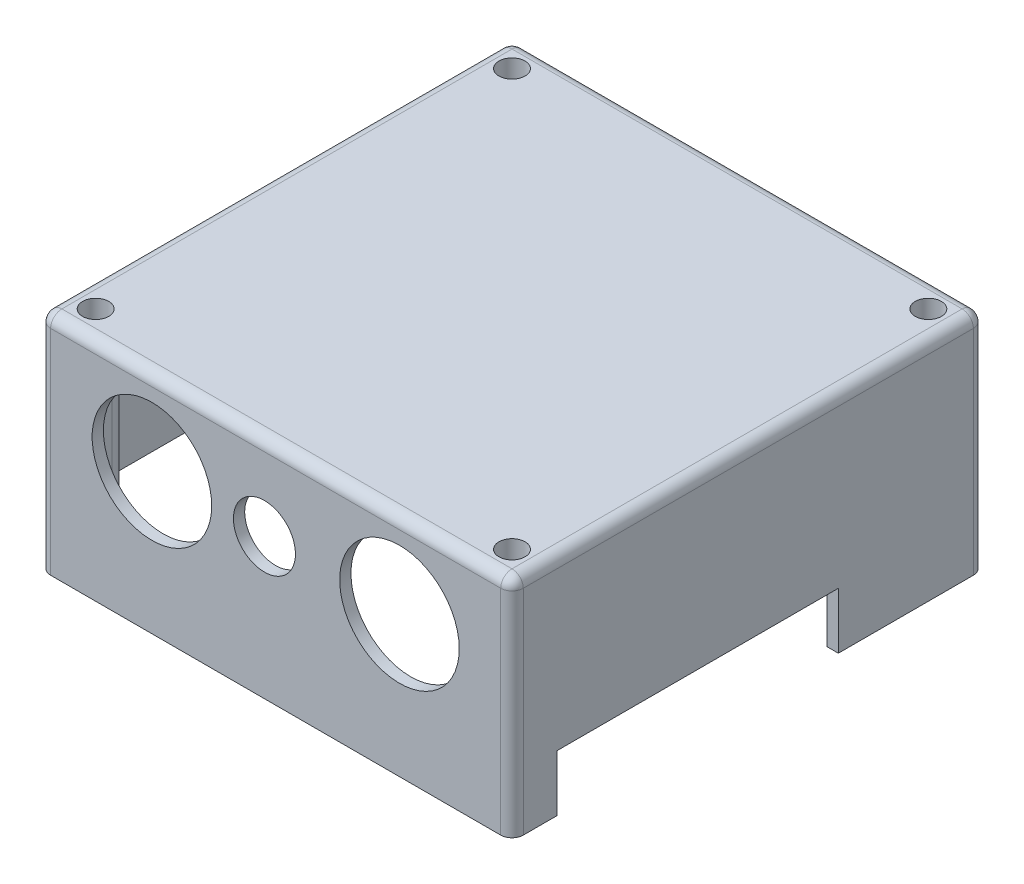
SolidWorks part; units mm, degrees
ref_plane "Front Plane" through (0, 0, 0) normal (0, 0, 1) x (1, 0, 0)
ref_plane "Top Plane" through (0, 0, 0) normal (0, 1, 0) x (1, 0, 0)
ref_plane "Right Plane" through (0, 0, 0) normal (1, 0, 0) x (0, 0, -1)
sketch "Sketch1" plane through (0, 0, 0) normal (0, 1, 0) x (1, 0, 0)
  line L0 (0, 0) -> (0, 50.8)
  line L1 (0, 50.8) -> (50.8, 50.8)
  line L2 (50.8, 50.8) -> (50.8, 0)
  line L3 (50.8, 0) -> (0, 0)
  line L4 (29.845, 40.64) -> (28.575, 40.64)
  line L5 (30.48, 43.18) -> (30.48, 38.1)
  line L6 (30.48, 38.1) -> (27.94, 38.1)
  line L7 (27.94, 38.1) -> (27.94, 43.18)
  line L8 (27.94, 43.18) -> (30.48, 43.18)
  line L9 (28.3382, 37.639) -> (28.245, 37.7322)
  line L10 (28.245, 37.7322) -> (28.0586, 37.7322)
  line L11 (28.0586, 37.7322) -> (27.9654, 37.639)
  line L12 (27.9654, 37.639) -> (27.9654, 37.2661)
  line L13 (27.9654, 37.2661) -> (28.0586, 37.1729)
  line L14 (28.0586, 37.1729) -> (28.245, 37.1729)
  line L15 (28.245, 37.1729) -> (28.3382, 37.2661)
  line L16 (28.5267, 37.5457) -> (28.7131, 37.7322)
  line L17 (28.7131, 37.7322) -> (28.7131, 37.1729)
  line L18 (28.5267, 37.1729) -> (28.8996, 37.1729)
  line L19 (28.2829, 43.8957) -> (28.4693, 44.0822)
  line L20 (28.4693, 44.0822) -> (28.4693, 43.5229)
  line L21 (28.2829, 43.5229) -> (28.6557, 43.5229)
  line L22 (28.8442, 43.6161) -> (28.8442, 43.989)
  line L23 (28.8442, 43.989) -> (28.9374, 44.0822)
  line L24 (28.9374, 44.0822) -> (29.1238, 44.0822)
  line L25 (29.1238, 44.0822) -> (29.2171, 43.989)
  line L26 (29.2171, 43.989) -> (29.2171, 43.6161)
  line L27 (29.2171, 43.6161) -> (29.1238, 43.5229)
  line L28 (29.1238, 43.5229) -> (28.9374, 43.5229)
  line L29 (28.9374, 43.5229) -> (28.8442, 43.6161)
  line L30 (28.8442, 43.6161) -> (29.2171, 43.989)
  line L31 (29.4055, 43.8957) -> (29.4055, 43.6161)
  line L32 (29.4055, 43.6161) -> (29.4987, 43.5229)
  line L33 (29.4987, 43.5229) -> (29.7784, 43.5229)
  line L34 (29.7784, 43.5229) -> (29.7784, 43.8957)
  line L35 (29.9668, 43.5229) -> (29.9668, 44.0822)
  line L36 (29.9668, 44.0822) -> (30.3397, 44.0822)
  line L37 (29.9668, 43.8025) -> (30.1533, 43.8025)
  line L38 (24.765, 40.64) -> (26.035, 40.64)
  line L39 (24.13, 38.1) -> (24.13, 43.18)
  line L40 (24.13, 43.18) -> (26.67, 43.18)
  line L41 (26.67, 43.18) -> (26.67, 38.1)
  line L42 (26.67, 38.1) -> (24.13, 38.1)
  line L43 (24.6756, 37.6644) -> (24.5824, 37.7576)
  line L44 (24.5824, 37.7576) -> (24.396, 37.7576)
  line L45 (24.396, 37.7576) -> (24.3028, 37.6644)
  line L46 (24.3028, 37.6644) -> (24.3028, 37.2915)
  line L47 (24.3028, 37.2915) -> (24.396, 37.1983)
  line L48 (24.396, 37.1983) -> (24.5824, 37.1983)
  line L49 (24.5824, 37.1983) -> (24.6756, 37.2915)
  line L50 (25.2369, 37.1983) -> (24.8641, 37.1983)
  line L51 (24.8641, 37.1983) -> (25.2369, 37.5711)
  line L52 (25.2369, 37.5711) -> (25.2369, 37.6644)
  line L53 (25.2369, 37.6644) -> (25.1437, 37.7576)
  line L54 (25.1437, 37.7576) -> (24.9573, 37.7576)
  line L55 (24.9573, 37.7576) -> (24.8641, 37.6644)
  line L56 (24.1326, 43.9211) -> (24.3191, 44.1076)
  line L57 (24.3191, 44.1076) -> (24.3191, 43.5483)
  line L58 (24.1326, 43.5483) -> (24.5055, 43.5483)
  line L59 (24.694, 43.6415) -> (24.694, 44.0144)
  line L60 (24.694, 44.0144) -> (24.7872, 44.1076)
  line L61 (24.7872, 44.1076) -> (24.9736, 44.1076)
  line L62 (24.9736, 44.1076) -> (25.0668, 44.0144)
  line L63 (25.0668, 44.0144) -> (25.0668, 43.6415)
  line L64 (25.0668, 43.6415) -> (24.9736, 43.5483)
  line L65 (24.9736, 43.5483) -> (24.7872, 43.5483)
  line L66 (24.7872, 43.5483) -> (24.694, 43.6415)
  line L67 (24.694, 43.6415) -> (25.0668, 44.0144)
  line L68 (25.2553, 43.9211) -> (25.2553, 43.6415)
  line L69 (25.2553, 43.6415) -> (25.3485, 43.5483)
  line L70 (25.3485, 43.5483) -> (25.6281, 43.5483)
  line L71 (25.6281, 43.5483) -> (25.6281, 43.9211)
  line L72 (25.8166, 43.5483) -> (25.8166, 44.1076)
  line L73 (25.8166, 44.1076) -> (26.1894, 44.1076)
  line L74 (25.8166, 43.8279) -> (26.003, 43.8279)
  line L75 (15.748, 34.29) -> (19.812, 34.29)
  line L76 (15.748, 34.29) -> (15.748, 31.75)
  line L77 (19.812, 31.75) -> (15.748, 31.75)
  line L78 (19.812, 31.75) -> (19.812, 34.29)
  line L79 (12.7, 33.02) -> (13.716, 33.02)
  line L80 (22.86, 33.02) -> (21.844, 33.02)
  line L81 (18.415, 33.02) -> (17.78, 33.02)
  line L82 (16.764, 32.385) -> (16.764, 33.655)
  line L83 (16.764, 33.655) -> (17.78, 33.02)
  line L84 (17.78, 33.02) -> (16.256, 33.02)
  line L85 (17.78, 33.02) -> (16.764, 32.385)
  line L86 (17.78, 32.385) -> (17.78, 33.02)
  line L87 (17.78, 33.02) -> (17.78, 33.655)
  line L88 (12.8591, 35.3702) -> (13.2404, 35.7515)
  line L89 (13.2404, 35.7515) -> (13.2404, 34.6075)
  line L90 (12.8591, 34.6075) -> (13.6217, 34.6075)
  line L91 (14.0285, 34.6075) -> (14.0285, 35.7515)
  line L92 (14.0285, 35.7515) -> (14.7912, 34.6075)
  line L93 (14.7912, 34.6075) -> (14.7912, 35.7515)
  line L94 (15.7699, 34.6075) -> (15.7699, 35.7515)
  line L95 (15.7699, 35.7515) -> (15.1979, 35.1795)
  line L96 (15.1979, 35.1795) -> (15.9605, 35.1795)
  line L97 (16.3673, 34.7982) -> (16.3673, 35.5608)
  line L98 (16.3673, 35.5608) -> (16.558, 35.7515)
  line L99 (16.558, 35.7515) -> (16.9393, 35.7515)
  line L100 (16.9393, 35.7515) -> (17.1299, 35.5608)
  line L101 (17.1299, 35.5608) -> (17.1299, 34.7982)
  line L102 (17.1299, 34.7982) -> (16.9393, 34.6075)
  line L103 (16.9393, 34.6075) -> (16.558, 34.6075)
  line L104 (16.558, 34.6075) -> (16.3673, 34.7982)
  line L105 (16.3673, 34.7982) -> (17.1299, 35.5608)
  line L106 (17.5367, 34.7982) -> (17.5367, 35.5608)
  line L107 (17.5367, 35.5608) -> (17.7273, 35.7515)
  line L108 (17.7273, 35.7515) -> (18.1087, 35.7515)
  line L109 (18.1087, 35.7515) -> (18.2993, 35.5608)
  line L110 (18.2993, 35.5608) -> (18.2993, 34.7982)
  line L111 (18.2993, 34.7982) -> (18.1087, 34.6075)
  line L112 (18.1087, 34.6075) -> (17.7273, 34.6075)
  line L113 (17.7273, 34.6075) -> (17.5367, 34.7982)
  line L114 (17.5367, 34.7982) -> (18.2993, 35.5608)
  line L115 (18.7061, 35.3702) -> (19.0874, 35.7515)
  line L116 (19.0874, 35.7515) -> (19.0874, 34.6075)
  line L117 (18.7061, 34.6075) -> (19.4687, 34.6075)
  line L118 (4.39, 39.64) -> (6.49, 39.64)
  line L119 (13.39, 50.34) -> (13.39, 53.24)
  line L120 (4.39, 53.24) -> (4.39, 50.34)
  line L121 (4.39, 53.24) -> (13.39, 53.24)
  line L122 (4.39, 50.34) -> (4.39, 45.04)
  line L123 (4.39, 39.64) -> (4.39, 40.34)
  line L124 (13.39, 50.34) -> (13.39, 39.64)
  line L125 (13.39, 39.64) -> (11.29, 39.64)
  line L126 (13.39, 50.34) -> (4.39, 50.34)
  line L127 (11.5901, 47.9299) -> (11.6536, 47.8663)
  line L128 (11.6536, 47.8663) -> (11.7172, 47.8663)
  line L129 (11.7172, 47.8663) -> (11.7807, 47.9299)
  line L130 (11.7807, 47.9299) -> (11.7807, 48.2476)
  line L131 (11.7172, 48.2476) -> (11.8443, 48.2476)
  line L132 (11.9643, 47.8663) -> (11.9643, 48.2476)
  line L133 (11.9643, 48.2476) -> (12.1549, 48.2476)
  line L134 (12.1549, 48.2476) -> (12.2185, 48.1841)
  line L135 (12.2185, 48.1841) -> (12.2185, 48.057)
  line L136 (12.2185, 48.057) -> (12.1549, 47.9934)
  line L137 (12.1549, 47.9934) -> (11.9643, 47.9934)
  line L138 (12.3385, 48.1205) -> (12.4656, 48.2476)
  line L139 (12.4656, 48.2476) -> (12.4656, 47.8663)
  line L140 (12.3385, 47.8663) -> (12.5927, 47.8663)
  line L141 (7.848, 49.1363) -> (7.848, 49.5176)
  line L142 (7.848, 49.5176) -> (8.0387, 49.5176)
  line L143 (8.0387, 49.5176) -> (8.1022, 49.4541)
  line L144 (8.1022, 49.4541) -> (8.1022, 49.327)
  line L145 (8.1022, 49.327) -> (8.0387, 49.2634)
  line L146 (8.0387, 49.2634) -> (7.848, 49.2634)
  line L147 (8.4129, 49.5176) -> (8.2858, 49.5176)
  line L148 (8.2858, 49.5176) -> (8.2222, 49.4541)
  line L149 (8.2222, 49.4541) -> (8.2222, 49.1999)
  line L150 (8.2222, 49.1999) -> (8.2858, 49.1363)
  line L151 (8.2858, 49.1363) -> (8.4129, 49.1363)
  line L152 (8.4129, 49.1363) -> (8.4764, 49.1999)
  line L153 (8.4764, 49.1999) -> (8.4764, 49.4541)
  line L154 (8.4764, 49.4541) -> (8.4129, 49.5176)
  line L155 (8.5964, 49.5176) -> (8.5964, 49.1363)
  line L156 (8.5964, 49.1363) -> (8.7235, 49.2634)
  line L157 (8.7235, 49.2634) -> (8.8506, 49.1363)
  line L158 (8.8506, 49.1363) -> (8.8506, 49.5176)
  line L159 (9.2248, 49.5176) -> (8.9706, 49.5176)
  line L160 (8.9706, 49.5176) -> (8.9706, 49.1363)
  line L161 (8.9706, 49.1363) -> (9.2248, 49.1363)
  line L162 (8.9706, 49.327) -> (9.0977, 49.327)
  line L163 (9.3448, 49.1363) -> (9.3448, 49.5176)
  line L164 (9.3448, 49.5176) -> (9.5355, 49.5176)
  line L165 (9.5355, 49.5176) -> (9.599, 49.4541)
  line L166 (9.599, 49.4541) -> (9.599, 49.327)
  line L167 (9.599, 49.327) -> (9.5355, 49.2634)
  line L168 (9.5355, 49.2634) -> (9.3448, 49.2634)
  line L169 (9.4719, 49.2634) -> (9.599, 49.1363)
  line L170 (9.719, 49.0727) -> (9.9733, 49.0727)
  line L171 (10.0932, 49.1999) -> (10.1568, 49.1363)
  line L172 (10.1568, 49.1363) -> (10.2204, 49.1363)
  line L173 (10.2204, 49.1363) -> (10.2839, 49.1999)
  line L174 (10.2839, 49.1999) -> (10.2839, 49.5176)
  line L175 (10.2204, 49.5176) -> (10.3475, 49.5176)
  line L176 (10.4674, 49.1363) -> (10.4674, 49.3905)
  line L177 (10.4674, 49.3905) -> (10.5945, 49.5176)
  line L178 (10.5945, 49.5176) -> (10.7217, 49.3905)
  line L179 (10.7217, 49.3905) -> (10.7217, 49.1363)
  line L180 (10.4674, 49.327) -> (10.7217, 49.327)
  line L181 (11.0959, 49.4541) -> (11.0323, 49.5176)
  line L182 (11.0323, 49.5176) -> (10.9052, 49.5176)
  line L183 (10.9052, 49.5176) -> (10.8417, 49.4541)
  line L184 (10.8417, 49.4541) -> (10.8417, 49.1999)
  line L185 (10.8417, 49.1999) -> (10.9052, 49.1363)
  line L186 (10.9052, 49.1363) -> (11.0323, 49.1363)
  line L187 (11.0323, 49.1363) -> (11.0959, 49.1999)
  line L188 (11.2159, 49.5176) -> (11.2159, 49.1363)
  line L189 (11.2159, 49.2634) -> (11.4701, 49.5176)
  line L190 (11.2794, 49.327) -> (11.4701, 49.1363)
  line L191 (11.5901, 49.1363) -> (11.5901, 49.5176)
  line L192 (11.5901, 49.5176) -> (11.7807, 49.5176)
  line L193 (11.7807, 49.5176) -> (11.8443, 49.4541)
  line L194 (11.8443, 49.4541) -> (11.8443, 49.327)
  line L195 (11.8443, 49.327) -> (11.7807, 49.2634)
  line L196 (11.7807, 49.2634) -> (11.5901, 49.2634)
  line L197 (12.0914, 49.1363) -> (12.0914, 49.5176)
  line L198 (11.9643, 49.5176) -> (12.2185, 49.5176)
  line L199 (12.3385, 49.1363) -> (12.3385, 49.5176)
  line L200 (12.3385, 49.327) -> (12.5927, 49.327)
  line L201 (12.5927, 49.5176) -> (12.5927, 49.1363)
  line L202 (10.795, 1.27) -> (24.765, 1.27)
  line L203 (24.765, 1.27) -> (24.765, 35.56)
  line L204 (24.765, 35.56) -> (10.795, 35.56)
  line L205 (10.795, 35.56) -> (10.795, 1.27)
  line L206 (14.1986, 3.8354) -> (13.6393, 3.8354)
  line L207 (13.6393, 3.8354) -> (13.6393, 4.115)
  line L208 (13.6393, 4.115) -> (13.7325, 4.2082)
  line L209 (13.7325, 4.2082) -> (13.919, 4.2082)
  line L210 (13.919, 4.2082) -> (14.0122, 4.115)
  line L211 (14.0122, 4.115) -> (14.0122, 3.8354)
  line L212 (14.0122, 4.0218) -> (14.1986, 4.2082)
  line L213 (13.6393, 4.3967) -> (14.1986, 4.7696)
  line L214 (13.6393, 4.7696) -> (14.1986, 4.3967)
  line L215 (16.7386, 4.0218) -> (16.1793, 4.0218)
  line L216 (16.1793, 3.8354) -> (16.1793, 4.2082)
  line L217 (16.1793, 4.3967) -> (16.7386, 4.7696)
  line L218 (16.1793, 4.7696) -> (16.7386, 4.3967)
  line L219 (18.8125, 4.2082) -> (18.7193, 4.115)
  line L220 (18.7193, 4.115) -> (18.7193, 3.9286)
  line L221 (18.7193, 3.9286) -> (18.8125, 3.8354)
  line L222 (18.8125, 3.8354) -> (19.1854, 3.8354)
  line L223 (19.1854, 3.8354) -> (19.2786, 3.9286)
  line L224 (19.2786, 3.9286) -> (19.2786, 4.115)
  line L225 (19.2786, 4.115) -> (19.1854, 4.2082)
  line L226 (19.1854, 4.2082) -> (18.999, 4.2082)
  line L227 (18.999, 4.2082) -> (18.999, 4.0218)
  line L228 (19.2786, 4.3967) -> (18.7193, 4.3967)
  line L229 (18.7193, 4.3967) -> (19.2786, 4.7696)
  line L230 (19.2786, 4.7696) -> (18.7193, 4.7696)
  line L231 (18.7193, 4.958) -> (19.2786, 4.958)
  line L232 (19.2786, 4.958) -> (19.2786, 5.2377)
  line L233 (19.2786, 5.2377) -> (19.1854, 5.3309)
  line L234 (19.1854, 5.3309) -> (18.8125, 5.3309)
  line L235 (18.8125, 5.3309) -> (18.7193, 5.2377)
  line L236 (18.7193, 5.2377) -> (18.7193, 4.958)
  line L237 (21.2593, 3.8354) -> (21.6322, 3.8354)
  line L238 (21.6322, 3.8354) -> (21.8186, 4.0218)
  line L239 (21.8186, 4.0218) -> (21.6322, 4.2082)
  line L240 (21.6322, 4.2082) -> (21.2593, 4.2082)
  line L241 (21.3525, 4.7696) -> (21.2593, 4.6763)
  line L242 (21.2593, 4.6763) -> (21.2593, 4.4899)
  line L243 (21.2593, 4.4899) -> (21.3525, 4.3967)
  line L244 (21.3525, 4.3967) -> (21.7254, 4.3967)
  line L245 (21.7254, 4.3967) -> (21.8186, 4.4899)
  line L246 (21.8186, 4.4899) -> (21.8186, 4.6763)
  line L247 (21.8186, 4.6763) -> (21.7254, 4.7696)
  line L248 (21.3525, 5.3309) -> (21.2593, 5.2377)
  line L249 (21.2593, 5.2377) -> (21.2593, 5.0512)
  line L250 (21.2593, 5.0512) -> (21.3525, 4.958)
  line L251 (21.3525, 4.958) -> (21.7254, 4.958)
  line L252 (21.7254, 4.958) -> (21.8186, 5.0512)
  line L253 (21.8186, 5.0512) -> (21.8186, 5.2377)
  line L254 (21.8186, 5.2377) -> (21.7254, 5.3309)
  line L255 (10.0752, 1.3335) -> (10.2235, 1.4818)
  line L256 (10.2235, 1.4818) -> (10.2235, 1.6301)
  line L257 (10.2235, 1.6301) -> (10.0752, 1.7784)
  line L258 (10.0752, 1.7784) -> (9.3337, 1.7784)
  line L259 (9.3337, 1.6301) -> (9.3337, 1.9267)
  line L260 (10.3718, 2.269) -> (10.3718, 2.8622)
  line L261 (10.2235, 3.2045) -> (9.3337, 3.2045)
  line L262 (9.3337, 3.2045) -> (9.3337, 3.6494)
  line L263 (9.3337, 3.6494) -> (9.482, 3.7977)
  line L264 (9.482, 3.7977) -> (9.6303, 3.7977)
  line L265 (9.6303, 3.7977) -> (9.7786, 3.6494)
  line L266 (9.7786, 3.6494) -> (9.9269, 3.7977)
  line L267 (9.9269, 3.7977) -> (10.0752, 3.7977)
  line L268 (10.0752, 3.7977) -> (10.2235, 3.6494)
  line L269 (10.2235, 3.6494) -> (10.2235, 3.2045)
  line L270 (9.7786, 3.2045) -> (9.7786, 3.6494)
  line L271 (10.2235, 4.4366) -> (9.3337, 4.4366)
  line L272 (9.3337, 4.14) -> (9.3337, 4.7332)
  line L273 (10.3718, 5.0756) -> (10.3718, 5.6687)
  line L274 (10.2235, 6.0111) -> (9.3337, 6.0111)
  line L275 (9.3337, 6.0111) -> (9.3337, 6.456)
  line L276 (9.3337, 6.456) -> (9.482, 6.6043)
  line L277 (9.482, 6.6043) -> (9.6303, 6.6043)
  line L278 (9.6303, 6.6043) -> (9.7786, 6.456)
  line L279 (9.7786, 6.456) -> (9.9269, 6.6043)
  line L280 (9.9269, 6.6043) -> (10.0752, 6.6043)
  line L281 (10.0752, 6.6043) -> (10.2235, 6.456)
  line L282 (10.2235, 6.456) -> (10.2235, 6.0111)
  line L283 (9.7786, 6.0111) -> (9.7786, 6.456)
  line L284 (9.3337, 7.3915) -> (9.3337, 7.0949)
  line L285 (9.3337, 7.0949) -> (9.482, 6.9466)
  line L286 (9.482, 6.9466) -> (10.0752, 6.9466)
  line L287 (10.0752, 6.9466) -> (10.2235, 7.0949)
  line L288 (10.2235, 7.0949) -> (10.2235, 7.3915)
  line L289 (10.2235, 7.3915) -> (10.0752, 7.5398)
  line L290 (10.0752, 7.5398) -> (9.482, 7.5398)
  line L291 (9.482, 7.5398) -> (9.3337, 7.3915)
  line L292 (10.2235, 7.8821) -> (9.6303, 7.8821)
  line L293 (9.6303, 7.8821) -> (9.3337, 8.1787)
  line L294 (9.3337, 8.1787) -> (9.6303, 8.4753)
  line L295 (9.6303, 8.4753) -> (10.2235, 8.4753)
  line L296 (9.7786, 7.8821) -> (9.7786, 8.4753)
  line L297 (10.2235, 8.8177) -> (9.3337, 8.8177)
  line L298 (9.3337, 8.8177) -> (9.3337, 9.2625)
  line L299 (9.3337, 9.2625) -> (9.482, 9.4108)
  line L300 (9.482, 9.4108) -> (9.7786, 9.4108)
  line L301 (9.7786, 9.4108) -> (9.9269, 9.2625)
  line L302 (9.9269, 9.2625) -> (9.9269, 8.8177)
  line L303 (9.9269, 9.1142) -> (10.2235, 9.4108)
  line L304 (9.3337, 9.7532) -> (10.2235, 9.7532)
  line L305 (10.2235, 9.7532) -> (10.2235, 10.198)
  line L306 (10.2235, 10.198) -> (10.0752, 10.3463)
  line L307 (10.0752, 10.3463) -> (9.482, 10.3463)
  line L308 (9.482, 10.3463) -> (9.3337, 10.198)
  line L309 (9.3337, 10.198) -> (9.3337, 9.7532)
  line L310 (10.3718, 10.6887) -> (10.3718, 11.2819)
  line L311 (9.6303, 11.6242) -> (9.3337, 11.9208)
  line L312 (9.3337, 11.9208) -> (10.2235, 11.9208)
  line L313 (10.2235, 11.6242) -> (10.2235, 12.2174)
  line L314 (3.81, 35.8648) -> (1.27, 35.8648)
  line L315 (0.9515, 36.2585) -> (2.0955, 36.2585)
  line L316 (2.0955, 36.2585) -> (2.0955, 37.0212)
  line L317 (0.9515, 38.1906) -> (0.9515, 37.4279)
  line L318 (0.9515, 37.4279) -> (2.0955, 37.4279)
  line L319 (2.0955, 37.4279) -> (2.0955, 38.1906)
  line L320 (1.5235, 37.4279) -> (1.5235, 37.8092)
  line L321 (0.9515, 38.5973) -> (2.0955, 38.5973)
  line L322 (2.0955, 38.5973) -> (2.0955, 39.1693)
  line L323 (2.0955, 39.1693) -> (1.9048, 39.3599)
  line L324 (1.9048, 39.3599) -> (1.1422, 39.3599)
  line L325 (1.1422, 39.3599) -> (0.9515, 39.1693)
  line L326 (0.9515, 39.1693) -> (0.9515, 38.5973)
  line L327 (1.3328, 39.7667) -> (0.9515, 40.148)
  line L328 (0.9515, 40.148) -> (2.0955, 40.148)
  line L329 (2.0955, 39.7667) -> (2.0955, 40.5293)
  line L330 (2.6768, 32.6898) -> (2.4032, 32.6898)
  line L331 (2.4032, 32.6898) -> (2.2098, 32.8832)
  line L332 (2.2098, 32.8832) -> (2.2098, 33.1568)
  line L333 (2.2098, 33.1568) -> (2.4032, 33.3502)
  line L334 (2.4032, 33.3502) -> (2.6768, 33.3502)
  line L335 (2.6768, 33.3502) -> (2.8702, 33.1568)
  line L336 (2.8702, 33.1568) -> (2.8702, 32.8832)
  line L337 (2.8702, 32.8832) -> (2.6768, 32.6898)
  line L338 (2.6768, 32.6898) -> (2.4032, 32.6898)
  line L339 (2.6768, 32.6898) -> (2.4032, 32.6898)
  line L340 (2.4032, 32.6898) -> (2.2098, 32.8832)
  line L341 (2.2098, 32.8832) -> (2.2098, 33.1568)
  line L342 (2.2098, 33.1568) -> (2.4032, 33.3502)
  line L343 (2.4032, 33.3502) -> (2.6768, 33.3502)
  line L344 (2.6768, 33.3502) -> (2.8702, 33.1568)
  line L345 (2.8702, 33.1568) -> (2.8702, 32.8832)
  line L346 (2.8702, 32.8832) -> (2.6768, 32.6898)
  line L347 (2.6768, 32.6898) -> (2.4032, 32.6898)
  line L348 (2.6768, 35.2298) -> (2.4032, 35.2298)
  line L349 (2.4032, 35.2298) -> (2.2098, 35.4232)
  line L350 (2.2098, 35.4232) -> (2.2098, 35.6968)
  line L351 (2.2098, 35.6968) -> (2.4032, 35.8902)
  line L352 (2.4032, 35.8902) -> (2.6768, 35.8902)
  line L353 (2.6768, 35.8902) -> (2.8702, 35.6968)
  line L354 (2.8702, 35.6968) -> (2.8702, 35.4232)
  line L355 (2.8702, 35.4232) -> (2.6768, 35.2298)
  line L356 (2.6768, 35.2298) -> (2.4032, 35.2298)
  line L357 (2.6768, 35.2298) -> (2.4032, 35.2298)
  line L358 (2.4032, 35.2298) -> (2.2098, 35.4232)
  line L359 (2.2098, 35.4232) -> (2.2098, 35.6968)
  line L360 (2.2098, 35.6968) -> (2.4032, 35.8902)
  line L361 (2.4032, 35.8902) -> (2.6768, 35.8902)
  line L362 (2.6768, 35.8902) -> (2.8702, 35.6968)
  line L363 (2.8702, 35.6968) -> (2.8702, 35.4232)
  line L364 (2.8702, 35.4232) -> (2.6768, 35.2298)
  line L365 (2.6768, 35.2298) -> (2.4032, 35.2298)
  line L366 (10.16, 36.83) -> (10.16, 31.75)
  line L367 (10.16, 31.75) -> (5.08, 31.75)
  line L368 (5.08, 31.75) -> (5.08, 36.83)
  line L369 (5.08, 36.83) -> (10.16, 36.83)
  line L370 (8.9275, 32.8596) -> (8.9275, 32.6139)
  line L371 (8.9275, 32.6139) -> (9.0504, 32.491)
  line L372 (9.0504, 32.491) -> (9.5418, 32.491)
  line L373 (9.5418, 32.491) -> (9.6647, 32.6139)
  line L374 (9.6647, 32.6139) -> (9.6647, 32.8596)
  line L375 (9.6647, 32.8596) -> (9.5418, 32.9825)
  line L376 (9.5418, 32.9825) -> (9.0504, 32.9825)
  line L377 (9.0504, 32.9825) -> (8.9275, 32.8596)
  line L378 (9.6647, 33.2394) -> (8.9275, 33.2394)
  line L379 (8.9275, 33.2394) -> (9.6647, 33.7309)
  line L380 (9.6647, 33.7309) -> (8.9275, 33.7309)
  line L381 (8.9275, 34.3565) -> (8.9275, 34.1107)
  line L382 (8.9275, 34.1107) -> (9.0504, 33.9878)
  line L383 (9.0504, 33.9878) -> (9.5418, 33.9878)
  line L384 (9.5418, 33.9878) -> (9.6647, 34.1107)
  line L385 (9.6647, 34.1107) -> (9.6647, 34.3565)
  line L386 (9.6647, 34.3565) -> (9.5418, 34.4793)
  line L387 (9.5418, 34.4793) -> (9.0504, 34.4793)
  line L388 (9.0504, 34.4793) -> (8.9275, 34.3565)
  line L389 (9.6647, 34.7363) -> (8.9275, 34.7363)
  line L390 (8.9275, 34.7363) -> (8.9275, 35.2277)
  line L391 (9.2961, 34.7363) -> (9.2961, 34.982)
  line L392 (9.6647, 35.4847) -> (8.9275, 35.4847)
  line L393 (8.9275, 35.4847) -> (8.9275, 35.9762)
  line L394 (9.2961, 35.4847) -> (9.2961, 35.7304)
  line L395 (5.7525, 31.7426) -> (6.4897, 31.7426)
  line L396 (6.4897, 31.7426) -> (6.4897, 32.1112)
  line L397 (6.4897, 32.1112) -> (6.3668, 32.2341)
  line L398 (6.3668, 32.2341) -> (5.8754, 32.2341)
  line L399 (5.8754, 32.2341) -> (5.7525, 32.1112)
  line L400 (5.7525, 32.1112) -> (5.7525, 31.7426)
  line L401 (5.8754, 32.9825) -> (5.7525, 32.8596)
  line L402 (5.7525, 32.8596) -> (5.7525, 32.6139)
  line L403 (5.7525, 32.6139) -> (5.8754, 32.491)
  line L404 (5.8754, 32.491) -> (5.9982, 32.491)
  line L405 (5.9982, 32.491) -> (6.1211, 32.6139)
  line L406 (6.1211, 32.6139) -> (6.1211, 32.8596)
  line L407 (6.1211, 32.8596) -> (6.244, 32.9825)
  line L408 (6.244, 32.9825) -> (6.3668, 32.9825)
  line L409 (6.3668, 32.9825) -> (6.4897, 32.8596)
  line L410 (6.4897, 32.8596) -> (6.4897, 32.6139)
  line L411 (6.4897, 32.6139) -> (6.3668, 32.491)
  line L412 (6.1211, 33.2394) -> (6.1211, 33.7309)
  line L413 (6.4897, 34.4793) -> (6.4897, 33.9878)
  line L414 (6.4897, 33.9878) -> (5.9982, 34.4793)
  line L415 (5.9982, 34.4793) -> (5.8754, 34.4793)
  line L416 (5.8754, 34.4793) -> (5.7525, 34.3565)
  line L417 (5.7525, 34.3565) -> (5.7525, 34.1107)
  line L418 (5.7525, 34.1107) -> (5.8754, 33.9878)
  line L419 (6.4897, 35.2277) -> (6.4897, 34.7363)
  line L420 (6.4897, 34.7363) -> (5.9982, 35.2277)
  line L421 (5.9982, 35.2277) -> (5.8754, 35.2277)
  line L422 (5.8754, 35.2277) -> (5.7525, 35.1049)
  line L423 (5.7525, 35.1049) -> (5.7525, 34.8591)
  line L424 (5.7525, 34.8591) -> (5.8754, 34.7363)
  line L425 (5.8754, 35.4847) -> (5.7525, 35.6075)
  line L426 (5.7525, 35.6075) -> (5.7525, 35.8533)
  line L427 (5.7525, 35.8533) -> (5.8754, 35.9762)
  line L428 (5.8754, 35.9762) -> (5.9982, 35.9762)
  line L429 (5.9982, 35.9762) -> (6.1211, 35.8533)
  line L430 (6.1211, 35.8533) -> (6.244, 35.9762)
  line L431 (6.244, 35.9762) -> (6.3668, 35.9762)
  line L432 (6.3668, 35.9762) -> (6.4897, 35.8533)
  line L433 (6.4897, 35.8533) -> (6.4897, 35.6075)
  line L434 (6.4897, 35.6075) -> (6.3668, 35.4847)
  line L435 (6.3668, 35.4847) -> (6.244, 35.4847)
  line L436 (6.244, 35.4847) -> (6.1211, 35.6075)
  line L437 (6.1211, 35.6075) -> (5.9982, 35.4847)
  line L438 (5.9982, 35.4847) -> (5.8754, 35.4847)
  line L439 (6.1211, 35.6075) -> (6.1211, 35.8533)
  line L440 (15.24, 21.082) -> (20.32, 21.082)
  line L441 (20.32, 21.082) -> (20.32, 20.32)
  line L442 (20.32, 20.32) -> (20.32, 19.558)
  line L443 (20.32, 19.558) -> (15.24, 19.558)
  line L444 (15.24, 19.558) -> (15.24, 20.32)
  line L445 (15.24, 20.32) -> (15.24, 21.082)
  line L446 (20.32, 20.32) -> (20.574, 20.32)
  line L447 (15.24, 20.32) -> (14.986, 20.32)
  line L448 (15.2527, 21.6027) -> (15.2527, 21.984)
  line L449 (15.2527, 21.984) -> (15.4434, 21.984)
  line L450 (15.4434, 21.984) -> (15.5069, 21.9205)
  line L451 (15.5069, 21.9205) -> (15.5069, 21.7934)
  line L452 (15.5069, 21.7934) -> (15.4434, 21.7298)
  line L453 (15.4434, 21.7298) -> (15.2527, 21.7298)
  line L454 (15.3798, 21.7298) -> (15.5069, 21.6027)
  line L455 (15.6269, 21.8569) -> (15.754, 21.984)
  line L456 (15.754, 21.984) -> (15.754, 21.6027)
  line L457 (15.6269, 21.6027) -> (15.8811, 21.6027)
  line L458 (15.8242, 20.5914) -> (16.1123, 20.8795)
  line L459 (16.1123, 20.8795) -> (16.1123, 20.0152)
  line L460 (15.8242, 20.0152) -> (16.4004, 20.0152)
  line L461 (16.7597, 20.1593) -> (16.7597, 20.7355)
  line L462 (16.7597, 20.7355) -> (16.9038, 20.8795)
  line L463 (16.9038, 20.8795) -> (17.1919, 20.8795)
  line L464 (17.1919, 20.8795) -> (17.3359, 20.7355)
  line L465 (17.3359, 20.7355) -> (17.3359, 20.1593)
  line L466 (17.3359, 20.1593) -> (17.1919, 20.0152)
  line L467 (17.1919, 20.0152) -> (16.9038, 20.0152)
  line L468 (16.9038, 20.0152) -> (16.7597, 20.1593)
  line L469 (16.7597, 20.1593) -> (17.3359, 20.7355)
  line L470 (17.6952, 20.8795) -> (17.6952, 20.0152)
  line L471 (17.6952, 20.3033) -> (18.2715, 20.8795)
  line L472 (17.8393, 20.4474) -> (18.2715, 20.0152)
  line L473 (15.24, 18.542) -> (20.32, 18.542)
  line L474 (20.32, 18.542) -> (20.32, 17.78)
  line L475 (20.32, 17.78) -> (20.32, 17.018)
  line L476 (20.32, 17.018) -> (15.24, 17.018)
  line L477 (15.24, 17.018) -> (15.24, 17.78)
  line L478 (15.24, 17.78) -> (15.24, 18.542)
  line L479 (20.32, 17.78) -> (20.574, 17.78)
  line L480 (15.24, 17.78) -> (14.986, 17.78)
  line L481 (15.2527, 19.0627) -> (15.2527, 19.444)
  line L482 (15.2527, 19.444) -> (15.4434, 19.444)
  line L483 (15.4434, 19.444) -> (15.5069, 19.3805)
  line L484 (15.5069, 19.3805) -> (15.5069, 19.2534)
  line L485 (15.5069, 19.2534) -> (15.4434, 19.1898)
  line L486 (15.4434, 19.1898) -> (15.2527, 19.1898)
  line L487 (15.3798, 19.1898) -> (15.5069, 19.0627)
  line L488 (15.8811, 19.0627) -> (15.6269, 19.0627)
  line L489 (15.6269, 19.0627) -> (15.8811, 19.3169)
  line L490 (15.8811, 19.3169) -> (15.8811, 19.3805)
  line L491 (15.8811, 19.3805) -> (15.8176, 19.444)
  line L492 (15.8176, 19.444) -> (15.6905, 19.444)
  line L493 (15.6905, 19.444) -> (15.6269, 19.3805)
  line L494 (15.8242, 18.0514) -> (16.1123, 18.3395)
  line L495 (16.1123, 18.3395) -> (16.1123, 17.4752)
  line L496 (15.8242, 17.4752) -> (16.4004, 17.4752)
  line L497 (16.7597, 17.6193) -> (16.7597, 18.1955)
  line L498 (16.7597, 18.1955) -> (16.9038, 18.3395)
  line L499 (16.9038, 18.3395) -> (17.1919, 18.3395)
  line L500 (17.1919, 18.3395) -> (17.3359, 18.1955)
  line L501 (17.3359, 18.1955) -> (17.3359, 17.6193)
  line L502 (17.3359, 17.6193) -> (17.1919, 17.4752)
  line L503 (17.1919, 17.4752) -> (16.9038, 17.4752)
  line L504 (16.9038, 17.4752) -> (16.7597, 17.6193)
  line L505 (16.7597, 17.6193) -> (17.3359, 18.1955)
  line L506 (17.6952, 18.3395) -> (17.6952, 17.4752)
  line L507 (17.6952, 17.7633) -> (18.2715, 18.3395)
  line L508 (17.8393, 17.9074) -> (18.2715, 17.4752)
  line L509 (15.24, 16.002) -> (20.32, 16.002)
  line L510 (20.32, 16.002) -> (20.32, 15.24)
  line L511 (20.32, 15.24) -> (20.32, 14.478)
  line L512 (20.32, 14.478) -> (15.24, 14.478)
  line L513 (15.24, 14.478) -> (15.24, 15.24)
  line L514 (15.24, 15.24) -> (15.24, 16.002)
  line L515 (20.32, 15.24) -> (20.574, 15.24)
  line L516 (15.24, 15.24) -> (14.986, 15.24)
  line L517 (15.2527, 16.5227) -> (15.2527, 16.904)
  line L518 (15.2527, 16.904) -> (15.4434, 16.904)
  line L519 (15.4434, 16.904) -> (15.5069, 16.8405)
  line L520 (15.5069, 16.8405) -> (15.5069, 16.7134)
  line L521 (15.5069, 16.7134) -> (15.4434, 16.6498)
  line L522 (15.4434, 16.6498) -> (15.2527, 16.6498)
  line L523 (15.3798, 16.6498) -> (15.5069, 16.5227)
  line L524 (15.6269, 16.8405) -> (15.6905, 16.904)
  line L525 (15.6905, 16.904) -> (15.8176, 16.904)
  line L526 (15.8176, 16.904) -> (15.8811, 16.8405)
  line L527 (15.8811, 16.8405) -> (15.8811, 16.7769)
  line L528 (15.8811, 16.7769) -> (15.8176, 16.7134)
  line L529 (15.8176, 16.7134) -> (15.754, 16.7134)
  line L530 (15.8176, 16.7134) -> (15.8811, 16.6498)
  line L531 (15.8811, 16.6498) -> (15.8811, 16.5863)
  line L532 (15.8811, 16.5863) -> (15.8176, 16.5227)
  line L533 (15.8176, 16.5227) -> (15.6905, 16.5227)
  line L534 (15.6905, 16.5227) -> (15.6269, 16.5863)
  line L535 (15.8242, 15.5114) -> (16.1123, 15.7995)
  line L536 (16.1123, 15.7995) -> (16.1123, 14.9352)
  line L537 (15.8242, 14.9352) -> (16.4004, 14.9352)
  line L538 (16.7597, 15.0793) -> (16.7597, 15.6555)
  line L539 (16.7597, 15.6555) -> (16.9038, 15.7995)
  line L540 (16.9038, 15.7995) -> (17.1919, 15.7995)
  line L541 (17.1919, 15.7995) -> (17.3359, 15.6555)
  line L542 (17.3359, 15.6555) -> (17.3359, 15.0793)
  line L543 (17.3359, 15.0793) -> (17.1919, 14.9352)
  line L544 (17.1919, 14.9352) -> (16.9038, 14.9352)
  line L545 (16.9038, 14.9352) -> (16.7597, 15.0793)
  line L546 (16.7597, 15.0793) -> (17.3359, 15.6555)
  line L547 (17.6952, 15.7995) -> (17.6952, 14.9352)
  line L548 (17.6952, 15.2233) -> (18.2715, 15.7995)
  line L549 (17.8393, 15.3674) -> (18.2715, 14.9352)
  line L550 (15.24, 13.462) -> (20.32, 13.462)
  line L551 (20.32, 13.462) -> (20.32, 12.7)
  line L552 (20.32, 12.7) -> (20.32, 11.938)
  line L553 (20.32, 11.938) -> (15.24, 11.938)
  line L554 (15.24, 11.938) -> (15.24, 12.7)
  line L555 (15.24, 12.7) -> (15.24, 13.462)
  line L556 (20.32, 12.7) -> (20.574, 12.7)
  line L557 (15.24, 12.7) -> (14.986, 12.7)
  line L558 (15.2527, 13.9827) -> (15.2527, 14.364)
  line L559 (15.2527, 14.364) -> (15.4434, 14.364)
  line L560 (15.4434, 14.364) -> (15.5069, 14.3005)
  line L561 (15.5069, 14.3005) -> (15.5069, 14.1734)
  line L562 (15.5069, 14.1734) -> (15.4434, 14.1098)
  line L563 (15.4434, 14.1098) -> (15.2527, 14.1098)
  line L564 (15.3798, 14.1098) -> (15.5069, 13.9827)
  line L565 (15.8176, 13.9827) -> (15.8176, 14.364)
  line L566 (15.8176, 14.364) -> (15.6269, 14.1734)
  line L567 (15.6269, 14.1734) -> (15.8811, 14.1734)
  line L568 (15.8242, 12.9714) -> (16.1123, 13.2595)
  line L569 (16.1123, 13.2595) -> (16.1123, 12.3952)
  line L570 (15.8242, 12.3952) -> (16.4004, 12.3952)
  line L571 (16.7597, 12.5393) -> (16.7597, 13.1155)
  line L572 (16.7597, 13.1155) -> (16.9038, 13.2595)
  line L573 (16.9038, 13.2595) -> (17.1919, 13.2595)
  line L574 (17.1919, 13.2595) -> (17.3359, 13.1155)
  line L575 (17.3359, 13.1155) -> (17.3359, 12.5393)
  line L576 (17.3359, 12.5393) -> (17.1919, 12.3952)
  line L577 (17.1919, 12.3952) -> (16.9038, 12.3952)
  line L578 (16.9038, 12.3952) -> (16.7597, 12.5393)
  line L579 (16.7597, 12.5393) -> (17.3359, 13.1155)
  line L580 (17.6952, 13.2595) -> (17.6952, 12.3952)
  line L581 (17.6952, 12.6833) -> (18.2715, 13.2595)
  line L582 (17.8393, 12.8274) -> (18.2715, 12.3952)
  line L583 (15.24, 10.922) -> (20.32, 10.922)
  line L584 (20.32, 10.922) -> (20.32, 10.16)
  line L585 (20.32, 10.16) -> (20.32, 9.398)
  line L586 (20.32, 9.398) -> (15.24, 9.398)
  line L587 (15.24, 9.398) -> (15.24, 10.16)
  line L588 (15.24, 10.16) -> (15.24, 10.922)
  line L589 (20.32, 10.16) -> (20.574, 10.16)
  line L590 (15.24, 10.16) -> (14.986, 10.16)
  line L591 (15.2527, 11.4427) -> (15.2527, 11.824)
  line L592 (15.2527, 11.824) -> (15.4434, 11.824)
  line L593 (15.4434, 11.824) -> (15.5069, 11.7605)
  line L594 (15.5069, 11.7605) -> (15.5069, 11.6334)
  line L595 (15.5069, 11.6334) -> (15.4434, 11.5698)
  line L596 (15.4434, 11.5698) -> (15.2527, 11.5698)
  line L597 (15.3798, 11.5698) -> (15.5069, 11.4427)
  line L598 (15.8811, 11.824) -> (15.6269, 11.824)
  line L599 (15.6269, 11.824) -> (15.6269, 11.6334)
  line L600 (15.6269, 11.6334) -> (15.754, 11.6969)
  line L601 (15.754, 11.6969) -> (15.8176, 11.6969)
  line L602 (15.8176, 11.6969) -> (15.8811, 11.6334)
  line L603 (15.8811, 11.6334) -> (15.8811, 11.5063)
  line L604 (15.8811, 11.5063) -> (15.8176, 11.4427)
  line L605 (15.8176, 11.4427) -> (15.6905, 11.4427)
  line L606 (15.6905, 11.4427) -> (15.6269, 11.5063)
  line L607 (15.8242, 10.4314) -> (16.1123, 10.7195)
  line L608 (16.1123, 10.7195) -> (16.1123, 9.8552)
  line L609 (15.8242, 9.8552) -> (16.4004, 9.8552)
  line L610 (16.7597, 9.9993) -> (16.7597, 10.5755)
  line L611 (16.7597, 10.5755) -> (16.9038, 10.7195)
  line L612 (16.9038, 10.7195) -> (17.1919, 10.7195)
  line L613 (17.1919, 10.7195) -> (17.3359, 10.5755)
  line L614 (17.3359, 10.5755) -> (17.3359, 9.9993)
  line L615 (17.3359, 9.9993) -> (17.1919, 9.8552)
  line L616 (17.1919, 9.8552) -> (16.9038, 9.8552)
  line L617 (16.9038, 9.8552) -> (16.7597, 9.9993)
  line L618 (16.7597, 9.9993) -> (17.3359, 10.5755)
  line L619 (17.6952, 10.7195) -> (17.6952, 9.8552)
  line L620 (17.6952, 10.1433) -> (18.2715, 10.7195)
  line L621 (17.8393, 10.2874) -> (18.2715, 9.8552)
  line L622 (15.24, 8.382) -> (20.32, 8.382)
  line L623 (20.32, 8.382) -> (20.32, 7.62)
  line L624 (20.32, 7.62) -> (20.32, 6.858)
  line L625 (20.32, 6.858) -> (15.24, 6.858)
  line L626 (15.24, 6.858) -> (15.24, 7.62)
  line L627 (15.24, 7.62) -> (15.24, 8.382)
  line L628 (20.32, 7.62) -> (20.574, 7.62)
  line L629 (15.24, 7.62) -> (14.986, 7.62)
  line L630 (15.2527, 8.9027) -> (15.2527, 9.284)
  line L631 (15.2527, 9.284) -> (15.4434, 9.284)
  line L632 (15.4434, 9.284) -> (15.5069, 9.2205)
  line L633 (15.5069, 9.2205) -> (15.5069, 9.0934)
  line L634 (15.5069, 9.0934) -> (15.4434, 9.0298)
  line L635 (15.4434, 9.0298) -> (15.2527, 9.0298)
  line L636 (15.3798, 9.0298) -> (15.5069, 8.9027)
  line L637 (15.8811, 9.284) -> (15.754, 9.2205)
  line L638 (15.754, 9.2205) -> (15.6269, 9.0934)
  line L639 (15.6269, 9.0934) -> (15.6269, 8.9663)
  line L640 (15.6269, 8.9663) -> (15.6905, 8.9027)
  line L641 (15.6905, 8.9027) -> (15.8176, 8.9027)
  line L642 (15.8176, 8.9027) -> (15.8811, 8.9663)
  line L643 (15.8811, 8.9663) -> (15.8811, 9.0298)
  line L644 (15.8811, 9.0298) -> (15.8176, 9.0934)
  line L645 (15.8176, 9.0934) -> (15.6269, 9.0934)
  line L646 (15.8242, 7.8914) -> (16.1123, 8.1795)
  line L647 (16.1123, 8.1795) -> (16.1123, 7.3152)
  line L648 (15.8242, 7.3152) -> (16.4004, 7.3152)
  line L649 (16.7597, 7.4593) -> (16.7597, 8.0355)
  line L650 (16.7597, 8.0355) -> (16.9038, 8.1795)
  line L651 (16.9038, 8.1795) -> (17.1919, 8.1795)
  line L652 (17.1919, 8.1795) -> (17.3359, 8.0355)
  line L653 (17.3359, 8.0355) -> (17.3359, 7.4593)
  line L654 (17.3359, 7.4593) -> (17.1919, 7.3152)
  line L655 (17.1919, 7.3152) -> (16.9038, 7.3152)
  line L656 (16.9038, 7.3152) -> (16.7597, 7.4593)
  line L657 (16.7597, 7.4593) -> (17.3359, 8.0355)
  line L658 (17.6952, 8.1795) -> (17.6952, 7.3152)
  line L659 (17.6952, 7.6033) -> (18.2715, 8.1795)
  line L660 (17.8393, 7.7474) -> (18.2715, 7.3152)
  line L661 (15.24, 28.702) -> (20.32, 28.702)
  line L662 (20.32, 28.702) -> (20.32, 27.94)
  line L663 (20.32, 27.94) -> (20.32, 27.178)
  line L664 (20.32, 27.178) -> (15.24, 27.178)
  line L665 (15.24, 27.178) -> (15.24, 27.94)
  line L666 (15.24, 27.94) -> (15.24, 28.702)
  line L667 (20.32, 27.94) -> (20.574, 27.94)
  line L668 (15.24, 27.94) -> (14.986, 27.94)
  line L669 (15.2527, 29.2227) -> (15.2527, 29.604)
  line L670 (15.2527, 29.604) -> (15.4434, 29.604)
  line L671 (15.4434, 29.604) -> (15.5069, 29.5405)
  line L672 (15.5069, 29.5405) -> (15.5069, 29.4134)
  line L673 (15.5069, 29.4134) -> (15.4434, 29.3498)
  line L674 (15.4434, 29.3498) -> (15.2527, 29.3498)
  line L675 (15.3798, 29.3498) -> (15.5069, 29.2227)
  line L676 (15.6269, 29.604) -> (15.8811, 29.604)
  line L677 (15.8811, 29.604) -> (15.8811, 29.5405)
  line L678 (15.8811, 29.5405) -> (15.6269, 29.2863)
  line L679 (15.6269, 29.2863) -> (15.6269, 29.2227)
  line L680 (15.8242, 28.2114) -> (16.1123, 28.4995)
  line L681 (16.1123, 28.4995) -> (16.1123, 27.6352)
  line L682 (15.8242, 27.6352) -> (16.4004, 27.6352)
  line L683 (16.7597, 27.6352) -> (16.7597, 27.7793)
  line L684 (16.7597, 27.7793) -> (16.9038, 27.7793)
  line L685 (16.9038, 27.7793) -> (16.9038, 27.6352)
  line L686 (16.9038, 27.6352) -> (16.7597, 27.6352)
  line L687 (17.2275, 28.2114) -> (17.5156, 28.4995)
  line L688 (17.5156, 28.4995) -> (17.5156, 27.6352)
  line L689 (17.2275, 27.6352) -> (17.8037, 27.6352)
  line L690 (18.163, 28.4995) -> (18.163, 27.6352)
  line L691 (18.163, 27.9233) -> (18.7392, 28.4995)
  line L692 (18.307, 28.0674) -> (18.7392, 27.6352)
  line L693 (25.4, 49.53) -> (30.48, 49.53)
  line L694 (30.48, 49.53) -> (30.48, 44.45)
  line L695 (30.48, 44.45) -> (25.4, 44.45)
  line L696 (25.4, 44.45) -> (25.4, 49.53)
  line L697 (26.0731, 48.2981) -> (26.0731, 49.0353)
  line L698 (26.0731, 49.0353) -> (26.4417, 49.0353)
  line L699 (26.4417, 49.0353) -> (26.5646, 48.9124)
  line L700 (26.5646, 48.9124) -> (26.5646, 48.6667)
  line L701 (26.5646, 48.6667) -> (26.4417, 48.5438)
  line L702 (26.4417, 48.5438) -> (26.0731, 48.5438)
  line L703 (26.3188, 48.5438) -> (26.5646, 48.2981)
  line L704 (27.313, 49.0353) -> (26.8215, 49.0353)
  line L705 (26.8215, 49.0353) -> (26.8215, 48.2981)
  line L706 (26.8215, 48.2981) -> (27.313, 48.2981)
  line L707 (26.8215, 48.6667) -> (27.0673, 48.6667)
  line L708 (28.0614, 48.9124) -> (27.9386, 49.0353)
  line L709 (27.9386, 49.0353) -> (27.6928, 49.0353)
  line L710 (27.6928, 49.0353) -> (27.5699, 48.9124)
  line L711 (27.5699, 48.9124) -> (27.5699, 48.7896)
  line L712 (27.5699, 48.7896) -> (27.6928, 48.6667)
  line L713 (27.6928, 48.6667) -> (27.9386, 48.6667)
  line L714 (27.9386, 48.6667) -> (28.0614, 48.5438)
  line L715 (28.0614, 48.5438) -> (28.0614, 48.421)
  line L716 (28.0614, 48.421) -> (27.9386, 48.2981)
  line L717 (27.9386, 48.2981) -> (27.6928, 48.2981)
  line L718 (27.6928, 48.2981) -> (27.5699, 48.421)
  line L719 (28.8098, 49.0353) -> (28.3184, 49.0353)
  line L720 (28.3184, 49.0353) -> (28.3184, 48.2981)
  line L721 (28.3184, 48.2981) -> (28.8098, 48.2981)
  line L722 (28.3184, 48.6667) -> (28.5641, 48.6667)
  line L723 (29.3125, 48.2981) -> (29.3125, 49.0353)
  line L724 (29.0668, 49.0353) -> (29.5583, 49.0353)
  line L725 (26.0731, 45.8603) -> (26.0731, 45.1231)
  line L726 (26.0731, 45.1231) -> (26.4417, 45.1231)
  line L727 (26.4417, 45.1231) -> (26.5646, 45.246)
  line L728 (26.5646, 45.246) -> (26.5646, 45.7374)
  line L729 (26.5646, 45.7374) -> (26.4417, 45.8603)
  line L730 (26.4417, 45.8603) -> (26.0731, 45.8603)
  line L731 (27.313, 45.7374) -> (27.1901, 45.8603)
  line L732 (27.1901, 45.8603) -> (26.9444, 45.8603)
  line L733 (26.9444, 45.8603) -> (26.8215, 45.7374)
  line L734 (26.8215, 45.7374) -> (26.8215, 45.6146)
  line L735 (26.8215, 45.6146) -> (26.9444, 45.4917)
  line L736 (26.9444, 45.4917) -> (27.1901, 45.4917)
  line L737 (27.1901, 45.4917) -> (27.313, 45.3688)
  line L738 (27.313, 45.3688) -> (27.313, 45.246)
  line L739 (27.313, 45.246) -> (27.1901, 45.1231)
  line L740 (27.1901, 45.1231) -> (26.9444, 45.1231)
  line L741 (26.9444, 45.1231) -> (26.8215, 45.246)
  line L742 (27.5699, 45.4917) -> (28.0614, 45.4917)
  line L743 (28.8098, 45.1231) -> (28.3184, 45.1231)
  line L744 (28.3184, 45.1231) -> (28.8098, 45.6146)
  line L745 (28.8098, 45.6146) -> (28.8098, 45.7374)
  line L746 (28.8098, 45.7374) -> (28.687, 45.8603)
  line L747 (28.687, 45.8603) -> (28.4412, 45.8603)
  line L748 (28.4412, 45.8603) -> (28.3184, 45.7374)
  line L749 (29.5583, 45.1231) -> (29.0668, 45.1231)
  line L750 (29.0668, 45.1231) -> (29.5583, 45.6146)
  line L751 (29.5583, 45.6146) -> (29.5583, 45.7374)
  line L752 (29.5583, 45.7374) -> (29.4354, 45.8603)
  line L753 (29.4354, 45.8603) -> (29.1896, 45.8603)
  line L754 (29.1896, 45.8603) -> (29.0668, 45.7374)
  line L755 (29.8152, 45.8603) -> (30.3067, 45.8603)
  line L756 (30.3067, 45.8603) -> (30.3067, 45.7374)
  line L757 (30.3067, 45.7374) -> (29.8152, 45.246)
  line L758 (29.8152, 45.246) -> (29.8152, 45.1231)
  line L759 (6.35, 20.32) -> (6.35, 30.48)
  line L760 (6.35, 30.48) -> (-5.08, 30.48)
  line L761 (-5.08, 30.48) -> (-5.08, 20.32)
  line L762 (-5.08, 20.32) -> (6.35, 20.32)
  line L763 (6.35, 20.32) -> (6.35, 30.48)
  line L764 (6.223, 20.32) -> (6.223, 30.48)
  line L765 (6.096, 20.32) -> (6.096, 30.48)
  line L766 (5.969, 20.32) -> (5.969, 30.48)
  line L767 (5.842, 20.32) -> (5.842, 30.48)
  line L768 (5.715, 20.32) -> (5.715, 30.48)
  line L769 (5.588, 20.32) -> (5.588, 30.48)
  line L770 (5.461, 20.32) -> (5.461, 30.48)
  line L771 (5.334, 20.32) -> (5.334, 30.48)
  line L772 (5.207, 20.32) -> (5.207, 30.48)
  line L773 (5.08, 20.32) -> (5.08, 30.48)
  line L774 (4.953, 20.32) -> (4.953, 30.48)
  line L775 (4.826, 20.32) -> (4.826, 30.48)
  line L776 (4.699, 20.32) -> (4.699, 30.48)
  line L777 (4.572, 20.32) -> (4.572, 30.48)
  line L778 (4.445, 20.32) -> (4.445, 30.48)
  line L779 (4.318, 20.32) -> (4.318, 30.48)
  line L780 (4.191, 20.32) -> (4.191, 30.48)
  line L781 (4.064, 20.32) -> (4.064, 30.48)
  line L782 (3.937, 20.32) -> (3.937, 30.48)
  line L783 (3.81, 20.32) -> (3.81, 30.48)
  line L784 (3.683, 20.32) -> (3.683, 30.48)
  line L785 (3.556, 20.32) -> (3.556, 30.48)
  line L786 (3.429, 20.32) -> (3.429, 30.48)
  line L787 (3.302, 20.32) -> (3.302, 30.48)
  line L788 (3.175, 20.32) -> (3.175, 30.48)
  line L789 (3.048, 20.32) -> (3.048, 30.48)
  line L790 (2.921, 20.32) -> (2.921, 30.48)
  line L791 (2.794, 20.32) -> (2.794, 30.48)
  line L792 (2.667, 20.32) -> (2.667, 30.48)
  line L793 (2.54, 20.32) -> (2.54, 30.48)
  line L794 (2.413, 20.32) -> (2.413, 30.48)
  line L795 (2.286, 20.32) -> (2.286, 30.48)
  line L796 (2.159, 20.32) -> (2.159, 30.48)
  line L797 (2.032, 20.32) -> (2.032, 30.48)
  line L798 (1.905, 20.32) -> (1.905, 30.48)
  line L799 (1.778, 20.32) -> (1.778, 30.48)
  line L800 (1.651, 20.32) -> (1.651, 30.48)
  line L801 (1.524, 20.32) -> (1.524, 30.48)
  line L802 (1.397, 20.32) -> (1.397, 30.48)
  line L803 (1.27, 20.32) -> (1.27, 30.48)
  line L804 (1.143, 20.32) -> (1.143, 30.48)
  line L805 (1.016, 20.32) -> (1.016, 30.48)
  line L806 (0.889, 20.32) -> (0.889, 30.48)
  line L807 (0.762, 20.32) -> (0.762, 30.48)
  line L808 (0.635, 20.32) -> (0.635, 30.48)
  line L809 (0.508, 20.32) -> (0.508, 30.48)
  line L810 (0.381, 20.32) -> (0.381, 30.48)
  line L811 (0.254, 20.32) -> (0.254, 30.48)
  line L812 (0.127, 20.32) -> (0.127, 30.48)
  line L813 (0, 20.32) -> (0, 30.48)
  line L814 (-0.127, 20.32) -> (-0.127, 30.48)
  line L815 (-0.254, 20.32) -> (-0.254, 30.48)
  line L816 (-0.381, 20.32) -> (-0.381, 30.48)
  line L817 (-0.508, 20.32) -> (-0.508, 30.48)
  line L818 (-0.635, 20.32) -> (-0.635, 30.48)
  line L819 (-0.762, 20.32) -> (-0.762, 30.48)
  line L820 (-0.889, 20.32) -> (-0.889, 30.48)
  line L821 (-1.016, 20.32) -> (-1.016, 30.48)
  line L822 (-1.143, 20.32) -> (-1.143, 30.48)
  line L823 (-1.27, 20.32) -> (-1.27, 30.48)
  line L824 (-1.397, 20.32) -> (-1.397, 30.48)
  line L825 (-1.524, 20.32) -> (-1.524, 30.48)
  line L826 (-1.651, 20.32) -> (-1.651, 30.48)
  line L827 (-1.778, 20.32) -> (-1.778, 30.48)
  line L828 (-1.905, 20.32) -> (-1.905, 30.48)
  line L829 (-2.032, 20.32) -> (-2.032, 30.48)
  line L830 (-2.159, 20.32) -> (-2.159, 30.48)
  line L831 (-2.286, 20.32) -> (-2.286, 30.48)
  line L832 (-2.413, 20.32) -> (-2.413, 30.48)
  line L833 (-2.54, 20.32) -> (-2.54, 30.48)
  line L834 (-2.667, 20.32) -> (-2.667, 30.48)
  line L835 (-2.794, 20.32) -> (-2.794, 30.48)
  line L836 (-2.921, 20.32) -> (-2.921, 30.48)
  line L837 (-3.048, 20.32) -> (-3.048, 30.48)
  line L838 (-3.175, 20.32) -> (-3.175, 30.48)
  line L839 (-3.302, 20.32) -> (-3.302, 30.48)
  line L840 (-3.429, 20.32) -> (-3.429, 30.48)
  line L841 (-3.556, 20.32) -> (-3.556, 30.48)
  line L842 (-3.683, 20.32) -> (-3.683, 30.48)
  line L843 (-3.81, 20.32) -> (-3.81, 30.48)
  line L844 (-3.937, 20.32) -> (-3.937, 30.48)
  line L845 (-4.064, 20.32) -> (-4.064, 30.48)
  line L846 (-4.191, 20.32) -> (-4.191, 30.48)
  line L847 (-4.318, 20.32) -> (-4.318, 30.48)
  line L848 (-4.445, 20.32) -> (-4.445, 30.48)
  line L849 (-4.572, 20.32) -> (-4.572, 30.48)
  line L850 (-4.699, 20.32) -> (-4.699, 30.48)
  line L851 (-4.826, 20.32) -> (-4.826, 30.48)
  line L852 (-4.953, 20.32) -> (-4.953, 30.48)
  line L853 (8.89, 20.32) -> (8.89, 30.48)
  line L854 (43.18, 1.27) -> (25.4, 1.27)
  line L855 (25.4, 1.27) -> (25.4, 36.83)
  line L856 (25.4, 36.83) -> (43.18, 36.83)
  line L857 (43.18, 36.83) -> (43.18, 1.27)
  line L858 (35.56, 2.54) -> (33.02, 2.54)
  line L859 (33.02, 2.54) -> (33.02, 1.27)
  line L860 (33.02, 1.27) -> (25.4, 1.27)
  line L861 (25.4, 1.27) -> (25.4, 36.83)
  line L862 (25.4, 36.83) -> (43.18, 36.83)
  line L863 (43.18, 36.83) -> (43.18, 1.27)
  line L864 (43.18, 1.27) -> (35.56, 1.27)
  line L865 (35.56, 1.27) -> (35.56, 2.54)
  line L866 (35.5092, 12.1913) -> (34.3398, 12.1913)
  line L867 (34.3398, 11.8015) -> (34.3398, 12.5811)
  line L868 (34.3398, 13.7505) -> (34.3398, 12.9709)
  line L869 (34.3398, 12.9709) -> (35.5092, 12.9709)
  line L870 (35.5092, 12.9709) -> (35.5092, 13.7505)
  line L871 (34.9245, 12.9709) -> (34.9245, 13.3607)
  line L872 (34.3398, 14.9199) -> (34.3398, 14.1403)
  line L873 (34.3398, 14.1403) -> (35.5092, 14.1403)
  line L874 (35.5092, 14.1403) -> (35.5092, 14.9199)
  line L875 (34.9245, 14.1403) -> (34.9245, 14.5301)
  line L876 (35.5092, 15.3097) -> (34.3398, 15.3097)
  line L877 (34.3398, 15.3097) -> (35.5092, 16.0893)
  line L878 (35.5092, 16.0893) -> (34.3398, 16.0893)
  line L879 (34.5347, 17.2587) -> (34.3398, 17.0638)
  line L880 (34.3398, 17.0638) -> (34.3398, 16.674)
  line L881 (34.3398, 16.674) -> (34.5347, 16.4791)
  line L882 (34.5347, 16.4791) -> (34.7296, 16.4791)
  line L883 (34.7296, 16.4791) -> (34.9245, 16.674)
  line L884 (34.9245, 16.674) -> (34.9245, 17.0638)
  line L885 (34.9245, 17.0638) -> (35.1194, 17.2587)
  line L886 (35.1194, 17.2587) -> (35.3143, 17.2587)
  line L887 (35.3143, 17.2587) -> (35.5092, 17.0638)
  line L888 (35.5092, 17.0638) -> (35.5092, 16.674)
  line L889 (35.5092, 16.674) -> (35.3143, 16.4791)
  line L890 (34.3398, 17.6485) -> (34.5347, 17.6485)
  line L891 (34.5347, 17.6485) -> (34.9245, 18.0383)
  line L892 (34.9245, 18.0383) -> (34.5347, 18.4281)
  line L893 (34.5347, 18.4281) -> (34.3398, 18.4281)
  line L894 (34.9245, 18.0383) -> (35.5092, 18.0383)
  line L895 (35.7041, 18.8179) -> (35.7041, 19.5975)
  line L896 (34.5347, 19.9873) -> (34.3398, 20.1822)
  line L897 (34.3398, 20.1822) -> (34.3398, 20.572)
  line L898 (34.3398, 20.572) -> (34.5347, 20.7669)
  line L899 (34.5347, 20.7669) -> (34.7296, 20.7669)
  line L900 (34.7296, 20.7669) -> (34.9245, 20.572)
  line L901 (34.9245, 20.572) -> (34.9245, 20.3771)
  line L902 (34.9245, 20.572) -> (35.1194, 20.7669)
  line L903 (35.1194, 20.7669) -> (35.3143, 20.7669)
  line L904 (35.3143, 20.7669) -> (35.5092, 20.572)
  line L905 (35.5092, 20.572) -> (35.5092, 20.1822)
  line L906 (35.5092, 20.1822) -> (35.3143, 19.9873)
  line L907 (35.5092, 21.1567) -> (35.3143, 21.1567)
  line L908 (35.3143, 21.1567) -> (35.3143, 21.3516)
  line L909 (35.3143, 21.3516) -> (35.5092, 21.3516)
  line L910 (35.5092, 21.3516) -> (35.5092, 21.1567)
  line L911 (35.5092, 22.521) -> (35.5092, 21.7414)
  line L912 (35.5092, 21.7414) -> (34.7296, 22.521)
  line L913 (34.7296, 22.521) -> (34.5347, 22.521)
  line L914 (34.5347, 22.521) -> (34.3398, 22.3261)
  line L915 (34.3398, 22.3261) -> (34.3398, 21.9363)
  line L916 (34.3398, 21.9363) -> (34.5347, 21.7414)
  line L917 (18.415, 48.26) -> (18.415, 38.1)
  line L918 (18.415, 38.1) -> (14.605, 38.1)
  line L919 (14.605, 38.1) -> (13.97, 38.1)
  line L920 (13.97, 38.1) -> (13.97, 48.26)
  line L921 (13.97, 48.26) -> (14.605, 48.26)
  line L922 (14.605, 48.26) -> (18.415, 48.26)
  line L923 (14.605, 48.26) -> (14.605, 38.1)
  line L924 (23.495, 48.26) -> (23.495, 38.1)
  line L925 (23.495, 38.1) -> (19.685, 38.1)
  line L926 (19.685, 38.1) -> (19.05, 38.1)
  line L927 (19.05, 38.1) -> (19.05, 48.26)
  line L928 (19.05, 48.26) -> (19.685, 48.26)
  line L929 (19.685, 48.26) -> (23.495, 48.26)
  line L930 (19.685, 48.26) -> (19.685, 38.1)
  line L931 (46.77, 53.37) -> (31.97, 53.37)
  line L932 (31.97, 53.37) -> (31.97, 39.07)
  line L933 (31.97, 39.07) -> (46.77, 39.07)
  line L934 (46.77, 39.07) -> (46.77, 53.37)
  line L935 (44.45, 46.05) -> (43.18, 51.9)
  line L936 (43.18, 51.9) -> (41.91, 51.9)
  line L937 (41.91, 51.9) -> (40.64, 46.05)
  line L938 (38.1, 46.05) -> (36.83, 51.9)
  line L939 (36.83, 51.9) -> (35.56, 51.9)
  line L940 (35.56, 51.9) -> (34.29, 46.05)
  line L941 (43.205, 42.28) -> (43.205, 44.28)
  line L942 (43.205, 44.28) -> (42.58, 44.28)
  line L943 (42.58, 44.28) -> (42.58, 43.28)
  line L944 (42.58, 43.28) -> (42.58, 42.28)
  line L945 (42.58, 42.28) -> (43.205, 42.28)
  line L946 (42.58, 42.28) -> (41.83, 42.78)
  line L947 (41.83, 42.78) -> (42.58, 43.28)
  line L948 (42.58, 43.28) -> (41.83, 43.78)
  line L949 (41.83, 43.78) -> (42.58, 44.28)
  line L950 (41.83, 44.28) -> (42.58, 44.28)
  line L951 (41.83, 42.28) -> (42.58, 42.28)
  line L952 (41.08, 42.28) -> (41.08, 44.28)
  line L953 (41.08, 44.28) -> (39.33, 44.28)
  line L954 (39.33, 44.28) -> (39.33, 43.78)
  line L955 (39.33, 43.78) -> (40.455, 43.78)
  line L956 (40.455, 43.78) -> (40.455, 43.53)
  line L957 (40.455, 43.53) -> (39.33, 43.53)
  line L958 (39.33, 43.53) -> (39.33, 43.03)
  line L959 (39.33, 43.03) -> (40.455, 43.03)
  line L960 (40.455, 43.03) -> (40.455, 42.78)
  line L961 (40.455, 42.78) -> (39.33, 42.78)
  line L962 (39.33, 42.78) -> (39.33, 42.28)
  line L963 (39.33, 42.28) -> (41.08, 42.28)
  line L964 (39.08, 42.28) -> (39.08, 44.28)
  line L965 (39.08, 44.28) -> (38.455, 44.28)
  line L966 (38.455, 44.28) -> (38.455, 43.53)
  line L967 (38.455, 43.53) -> (37.955, 44.28)
  line L968 (37.955, 44.28) -> (37.205, 44.28)
  line L969 (37.205, 44.28) -> (37.705, 43.53)
  line L970 (38.455, 42.78) -> (38.455, 43.155)
  line L971 (39.08, 42.28) -> (37.705, 42.28)
  line L972 (38.455, 42.78) -> (38.08, 42.78)
  line L973 (38.455, 43.155) -> (38.08, 43.155)
  line L974 (35.705, 43.28) -> (35.205, 43.28)
  line L975 (35.705, 43.28) -> (35.705, 43.78)
  line L976 (35.21, 42.78) -> (35.21, 42.335)
  line L977 (35.205, 43.28) -> (35.205, 44.155)
  line L978 (35.7133, 45.2076) -> (35.4591, 45.2076)
  line L979 (35.4591, 45.2076) -> (35.4591, 44.8263)
  line L980 (35.4591, 44.8263) -> (35.7133, 44.8263)
  line L981 (35.4591, 45.017) -> (35.5862, 45.017)
  line L982 (36.2075, 45.2076) -> (36.2075, 44.8263)
  line L983 (36.2075, 44.8263) -> (36.4617, 44.8263)
  line L984 (37.2101, 45.2076) -> (36.9559, 45.2076)
  line L985 (36.9559, 45.2076) -> (36.9559, 44.8263)
  line L986 (36.9559, 44.8263) -> (37.2101, 44.8263)
  line L987 (36.9559, 45.017) -> (37.083, 45.017)
  line L988 (37.9585, 45.1441) -> (37.895, 45.2076)
  line L989 (37.895, 45.2076) -> (37.7679, 45.2076)
  line L990 (37.7679, 45.2076) -> (37.7043, 45.1441)
  line L991 (37.7043, 45.1441) -> (37.7043, 44.8899)
  line L992 (37.7043, 44.8899) -> (37.7679, 44.8263)
  line L993 (37.7679, 44.8263) -> (37.895, 44.8263)
  line L994 (37.895, 44.8263) -> (37.9585, 44.8899)
  line L995 (38.5798, 44.8263) -> (38.5798, 45.2076)
  line L996 (38.4527, 45.2076) -> (38.7069, 45.2076)
  line L997 (39.2011, 44.8263) -> (39.2011, 45.2076)
  line L998 (39.2011, 45.2076) -> (39.3918, 45.2076)
  line L999 (39.3918, 45.2076) -> (39.4553, 45.1441)
  line L1000 (39.4553, 45.1441) -> (39.4553, 45.017)
  line L1001 (39.4553, 45.017) -> (39.3918, 44.9534)
  line L1002 (39.3918, 44.9534) -> (39.2011, 44.9534)
  line L1003 (39.3282, 44.9534) -> (39.4553, 44.8263)
  line L1004 (40.1402, 45.2076) -> (40.0131, 45.2076)
  line L1005 (40.0131, 45.2076) -> (39.9496, 45.1441)
  line L1006 (39.9496, 45.1441) -> (39.9496, 44.8899)
  line L1007 (39.9496, 44.8899) -> (40.0131, 44.8263)
  line L1008 (40.0131, 44.8263) -> (40.1402, 44.8263)
  line L1009 (40.1402, 44.8263) -> (40.2038, 44.8899)
  line L1010 (40.2038, 44.8899) -> (40.2038, 45.1441)
  line L1011 (40.2038, 45.1441) -> (40.1402, 45.2076)
  line L1012 (40.698, 44.8263) -> (40.698, 45.2076)
  line L1013 (40.698, 45.2076) -> (40.9522, 44.8263)
  line L1014 (40.9522, 44.8263) -> (40.9522, 45.2076)
  line L1015 (41.4464, 44.8263) -> (41.5735, 44.8263)
  line L1016 (41.5099, 44.8263) -> (41.5099, 45.2076)
  line L1017 (41.4464, 45.2076) -> (41.5735, 45.2076)
  line L1018 (42.3243, 45.1441) -> (42.2607, 45.2076)
  line L1019 (42.2607, 45.2076) -> (42.1336, 45.2076)
  line L1020 (42.1336, 45.2076) -> (42.07, 45.1441)
  line L1021 (42.07, 45.1441) -> (42.07, 44.8899)
  line L1022 (42.07, 44.8899) -> (42.1336, 44.8263)
  line L1023 (42.1336, 44.8263) -> (42.2607, 44.8263)
  line L1024 (42.2607, 44.8263) -> (42.3243, 44.8899)
  line L1025 (43.0727, 45.1441) -> (43.0091, 45.2076)
  line L1026 (43.0091, 45.2076) -> (42.882, 45.2076)
  line L1027 (42.882, 45.2076) -> (42.8185, 45.1441)
  line L1028 (42.8185, 45.1441) -> (42.8185, 45.0805)
  line L1029 (42.8185, 45.0805) -> (42.882, 45.017)
  line L1030 (42.882, 45.017) -> (43.0091, 45.017)
  line L1031 (43.0091, 45.017) -> (43.0727, 44.9534)
  line L1032 (43.0727, 44.9534) -> (43.0727, 44.8899)
  line L1033 (43.0727, 44.8899) -> (43.0091, 44.8263)
  line L1034 (43.0091, 44.8263) -> (42.882, 44.8263)
  line L1035 (42.882, 44.8263) -> (42.8185, 44.8899)
  line L1036 (42.87, 41.199) -> (42.87, 39.741)
  line L1037 (42.87, 41.199) -> (42.87, 39.741)
  line L1038 (40.37, 41.199) -> (40.37, 39.741)
  line L1039 (40.37, 41.199) -> (40.37, 39.741)
  line L1040 (38.37, 41.199) -> (38.37, 39.741)
  line L1041 (38.37, 41.199) -> (38.37, 39.741)
  line L1042 (35.87, 41.199) -> (35.87, 39.741)
  line L1043 (35.87, 41.199) -> (35.87, 39.741)
  line L1044 (46.99, 35.56) -> (46.99, 20.32)
  line L1045 (46.99, 20.32) -> (58.42, 20.32)
  line L1046 (58.42, 20.32) -> (58.42, 35.56)
  line L1047 (58.42, 35.56) -> (46.99, 35.56)
  line L1048 (46.99, 35.56) -> (46.99, 20.32)
  line L1049 (47.117, 35.56) -> (47.117, 20.32)
  line L1050 (47.244, 35.56) -> (47.244, 20.32)
  line L1051 (47.371, 35.56) -> (47.371, 20.32)
  line L1052 (47.498, 35.56) -> (47.498, 20.32)
  line L1053 (47.625, 35.56) -> (47.625, 20.32)
  line L1054 (47.752, 35.56) -> (47.752, 20.32)
  line L1055 (47.879, 35.56) -> (47.879, 20.32)
  line L1056 (48.006, 35.56) -> (48.006, 20.32)
  line L1057 (48.133, 35.56) -> (48.133, 20.32)
  line L1058 (48.26, 35.56) -> (48.26, 20.32)
  line L1059 (48.387, 35.56) -> (48.387, 20.32)
  line L1060 (48.514, 35.56) -> (48.514, 20.32)
  line L1061 (48.641, 35.56) -> (48.641, 20.32)
  line L1062 (48.768, 35.56) -> (48.768, 20.32)
  line L1063 (48.895, 35.56) -> (48.895, 20.32)
  line L1064 (49.022, 35.56) -> (49.022, 20.32)
  line L1065 (49.149, 35.56) -> (49.149, 20.32)
  line L1066 (49.276, 35.56) -> (49.276, 20.32)
  line L1067 (49.403, 35.56) -> (49.403, 20.32)
  line L1068 (49.53, 35.56) -> (49.53, 20.32)
  line L1069 (49.657, 35.56) -> (49.657, 20.32)
  line L1070 (49.784, 35.56) -> (49.784, 20.32)
  line L1071 (49.911, 35.56) -> (49.911, 20.32)
  line L1072 (50.038, 35.56) -> (50.038, 20.32)
  line L1073 (50.165, 35.56) -> (50.165, 20.32)
  line L1074 (50.292, 35.56) -> (50.292, 20.32)
  line L1075 (50.419, 35.56) -> (50.419, 20.32)
  line L1076 (50.546, 35.56) -> (50.546, 20.32)
  line L1077 (50.673, 35.56) -> (50.673, 20.32)
  line L1078 (50.8, 35.56) -> (50.8, 20.32)
  line L1079 (50.927, 35.56) -> (50.927, 20.32)
  line L1080 (51.054, 35.56) -> (51.054, 20.32)
  line L1081 (51.181, 35.56) -> (51.181, 20.32)
  line L1082 (51.308, 35.56) -> (51.308, 20.32)
  line L1083 (51.435, 35.56) -> (51.435, 20.32)
  line L1084 (51.562, 35.56) -> (51.562, 20.32)
  line L1085 (51.689, 35.56) -> (51.689, 20.32)
  line L1086 (51.816, 35.56) -> (51.816, 20.32)
  line L1087 (51.943, 35.56) -> (51.943, 20.32)
  line L1088 (52.07, 35.56) -> (52.07, 20.32)
  line L1089 (52.197, 35.56) -> (52.197, 20.32)
  line L1090 (52.324, 35.56) -> (52.324, 20.32)
  line L1091 (52.451, 35.56) -> (52.451, 20.32)
  line L1092 (52.578, 35.56) -> (52.578, 20.32)
  line L1093 (52.705, 35.56) -> (52.705, 20.32)
  line L1094 (52.832, 35.56) -> (52.832, 20.32)
  line L1095 (52.959, 35.56) -> (52.959, 20.32)
  line L1096 (53.086, 35.56) -> (53.086, 20.32)
  line L1097 (53.213, 35.56) -> (53.213, 20.32)
  line L1098 (53.34, 35.56) -> (53.34, 20.32)
  line L1099 (53.467, 35.56) -> (53.467, 20.32)
  line L1100 (53.594, 35.56) -> (53.594, 20.32)
  line L1101 (53.721, 35.56) -> (53.721, 20.32)
  line L1102 (53.848, 35.56) -> (53.848, 20.32)
  line L1103 (53.975, 35.56) -> (53.975, 20.32)
  line L1104 (54.102, 35.56) -> (54.102, 20.32)
  line L1105 (54.229, 35.56) -> (54.229, 20.32)
  line L1106 (54.356, 35.56) -> (54.356, 20.32)
  line L1107 (54.483, 35.56) -> (54.483, 20.32)
  line L1108 (54.61, 35.56) -> (54.61, 20.32)
  line L1109 (54.737, 35.56) -> (54.737, 20.32)
  line L1110 (54.864, 35.56) -> (54.864, 20.32)
  line L1111 (54.991, 35.56) -> (54.991, 20.32)
  line L1112 (55.118, 35.56) -> (55.118, 20.32)
  line L1113 (55.245, 35.56) -> (55.245, 20.32)
  line L1114 (55.372, 35.56) -> (55.372, 20.32)
  line L1115 (55.499, 35.56) -> (55.499, 20.32)
  line L1116 (55.626, 35.56) -> (55.626, 20.32)
  line L1117 (55.753, 35.56) -> (55.753, 20.32)
  line L1118 (55.88, 35.56) -> (55.88, 20.32)
  line L1119 (56.007, 35.56) -> (56.007, 20.32)
  line L1120 (56.134, 35.56) -> (56.134, 20.32)
  line L1121 (56.261, 35.56) -> (56.261, 20.32)
  line L1122 (56.388, 35.56) -> (56.388, 20.32)
  line L1123 (56.515, 35.56) -> (56.515, 20.32)
  line L1124 (56.642, 35.56) -> (56.642, 20.32)
  line L1125 (56.769, 35.56) -> (56.769, 20.32)
  line L1126 (56.896, 35.56) -> (56.896, 20.32)
  line L1127 (57.023, 35.56) -> (57.023, 20.32)
  line L1128 (57.15, 35.56) -> (57.15, 20.32)
  line L1129 (57.277, 35.56) -> (57.277, 20.32)
  line L1130 (57.404, 35.56) -> (57.404, 20.32)
  line L1131 (57.531, 35.56) -> (57.531, 20.32)
  line L1132 (57.658, 35.56) -> (57.658, 20.32)
  line L1133 (57.785, 35.56) -> (57.785, 20.32)
  line L1134 (57.912, 35.56) -> (57.912, 20.32)
  line L1135 (58.039, 35.56) -> (58.039, 20.32)
  line L1136 (58.166, 35.56) -> (58.166, 20.32)
  line L1137 (58.293, 35.56) -> (58.293, 20.32)
  line L1138 (44.45, 35.56) -> (44.45, 20.32)
  line L1139 (46.99, 19.05) -> (46.99, 3.81)
  line L1140 (46.99, 3.81) -> (58.42, 3.81)
  line L1141 (58.42, 3.81) -> (58.42, 19.05)
  line L1142 (58.42, 19.05) -> (46.99, 19.05)
  line L1143 (46.99, 19.05) -> (46.99, 3.81)
  line L1144 (47.117, 19.05) -> (47.117, 3.81)
  line L1145 (47.244, 19.05) -> (47.244, 3.81)
  line L1146 (47.371, 19.05) -> (47.371, 3.81)
  line L1147 (47.498, 19.05) -> (47.498, 3.81)
  line L1148 (47.625, 19.05) -> (47.625, 3.81)
  line L1149 (47.752, 19.05) -> (47.752, 3.81)
  line L1150 (47.879, 19.05) -> (47.879, 3.81)
  line L1151 (48.006, 19.05) -> (48.006, 3.81)
  line L1152 (48.133, 19.05) -> (48.133, 3.81)
  line L1153 (48.26, 19.05) -> (48.26, 3.81)
  line L1154 (48.387, 19.05) -> (48.387, 3.81)
  line L1155 (48.514, 19.05) -> (48.514, 3.81)
  line L1156 (48.641, 19.05) -> (48.641, 3.81)
  line L1157 (48.768, 19.05) -> (48.768, 3.81)
  line L1158 (48.895, 19.05) -> (48.895, 3.81)
  line L1159 (49.022, 19.05) -> (49.022, 3.81)
  line L1160 (49.149, 19.05) -> (49.149, 3.81)
  line L1161 (49.276, 19.05) -> (49.276, 3.81)
  line L1162 (49.403, 19.05) -> (49.403, 3.81)
  line L1163 (49.53, 19.05) -> (49.53, 3.81)
  line L1164 (49.657, 19.05) -> (49.657, 3.81)
  line L1165 (49.784, 19.05) -> (49.784, 3.81)
  line L1166 (49.911, 19.05) -> (49.911, 3.81)
  line L1167 (50.038, 19.05) -> (50.038, 3.81)
  line L1168 (50.165, 19.05) -> (50.165, 3.81)
  line L1169 (50.292, 19.05) -> (50.292, 3.81)
  line L1170 (50.419, 19.05) -> (50.419, 3.81)
  line L1171 (50.546, 19.05) -> (50.546, 3.81)
  line L1172 (50.673, 19.05) -> (50.673, 3.81)
  line L1173 (50.8, 19.05) -> (50.8, 3.81)
  line L1174 (50.927, 19.05) -> (50.927, 3.81)
  line L1175 (51.054, 19.05) -> (51.054, 3.81)
  line L1176 (51.181, 19.05) -> (51.181, 3.81)
  line L1177 (51.308, 19.05) -> (51.308, 3.81)
  line L1178 (51.435, 19.05) -> (51.435, 3.81)
  line L1179 (51.562, 19.05) -> (51.562, 3.81)
  line L1180 (51.689, 19.05) -> (51.689, 3.81)
  line L1181 (51.816, 19.05) -> (51.816, 3.81)
  line L1182 (51.943, 19.05) -> (51.943, 3.81)
  line L1183 (52.07, 19.05) -> (52.07, 3.81)
  line L1184 (52.197, 19.05) -> (52.197, 3.81)
  line L1185 (52.324, 19.05) -> (52.324, 3.81)
  line L1186 (52.451, 19.05) -> (52.451, 3.81)
  line L1187 (52.578, 19.05) -> (52.578, 3.81)
  line L1188 (52.705, 19.05) -> (52.705, 3.81)
  line L1189 (52.832, 19.05) -> (52.832, 3.81)
  line L1190 (52.959, 19.05) -> (52.959, 3.81)
  line L1191 (53.086, 19.05) -> (53.086, 3.81)
  line L1192 (53.213, 19.05) -> (53.213, 3.81)
  line L1193 (53.34, 19.05) -> (53.34, 3.81)
  line L1194 (53.467, 19.05) -> (53.467, 3.81)
  line L1195 (53.594, 19.05) -> (53.594, 3.81)
  line L1196 (53.721, 19.05) -> (53.721, 3.81)
  line L1197 (53.848, 19.05) -> (53.848, 3.81)
  line L1198 (53.975, 19.05) -> (53.975, 3.81)
  line L1199 (54.102, 19.05) -> (54.102, 3.81)
  line L1200 (54.229, 19.05) -> (54.229, 3.81)
  line L1201 (54.356, 19.05) -> (54.356, 3.81)
  line L1202 (54.483, 19.05) -> (54.483, 3.81)
  line L1203 (54.61, 19.05) -> (54.61, 3.81)
  line L1204 (54.737, 19.05) -> (54.737, 3.81)
  line L1205 (54.864, 19.05) -> (54.864, 3.81)
  line L1206 (54.991, 19.05) -> (54.991, 3.81)
  line L1207 (55.118, 19.05) -> (55.118, 3.81)
  line L1208 (55.245, 19.05) -> (55.245, 3.81)
  line L1209 (55.372, 19.05) -> (55.372, 3.81)
  line L1210 (55.499, 19.05) -> (55.499, 3.81)
  line L1211 (55.626, 19.05) -> (55.626, 3.81)
  line L1212 (55.753, 19.05) -> (55.753, 3.81)
  line L1213 (55.88, 19.05) -> (55.88, 3.81)
  line L1214 (56.007, 19.05) -> (56.007, 3.81)
  line L1215 (56.134, 19.05) -> (56.134, 3.81)
  line L1216 (56.261, 19.05) -> (56.261, 3.81)
  line L1217 (56.388, 19.05) -> (56.388, 3.81)
  line L1218 (56.515, 19.05) -> (56.515, 3.81)
  line L1219 (56.642, 19.05) -> (56.642, 3.81)
  line L1220 (56.769, 19.05) -> (56.769, 3.81)
  line L1221 (56.896, 19.05) -> (56.896, 3.81)
  line L1222 (57.023, 19.05) -> (57.023, 3.81)
  line L1223 (57.15, 19.05) -> (57.15, 3.81)
  line L1224 (57.277, 19.05) -> (57.277, 3.81)
  line L1225 (57.404, 19.05) -> (57.404, 3.81)
  line L1226 (57.531, 19.05) -> (57.531, 3.81)
  line L1227 (57.658, 19.05) -> (57.658, 3.81)
  line L1228 (57.785, 19.05) -> (57.785, 3.81)
  line L1229 (57.912, 19.05) -> (57.912, 3.81)
  line L1230 (58.039, 19.05) -> (58.039, 3.81)
  line L1231 (58.166, 19.05) -> (58.166, 3.81)
  line L1232 (58.293, 19.05) -> (58.293, 3.81)
  line L1233 (44.45, 19.05) -> (44.45, 3.81)
  line L1234 (6.35, 3.81) -> (6.35, 19.05)
  line L1235 (6.35, 19.05) -> (-5.08, 19.05)
  line L1236 (-5.08, 19.05) -> (-5.08, 3.81)
  line L1237 (-5.08, 3.81) -> (6.35, 3.81)
  line L1238 (6.35, 3.81) -> (6.35, 19.05)
  line L1239 (6.223, 3.81) -> (6.223, 19.05)
  line L1240 (6.096, 3.81) -> (6.096, 19.05)
  line L1241 (5.969, 3.81) -> (5.969, 19.05)
  line L1242 (5.842, 3.81) -> (5.842, 19.05)
  line L1243 (5.715, 3.81) -> (5.715, 19.05)
  line L1244 (5.588, 3.81) -> (5.588, 19.05)
  line L1245 (5.461, 3.81) -> (5.461, 19.05)
  line L1246 (5.334, 3.81) -> (5.334, 19.05)
  line L1247 (5.207, 3.81) -> (5.207, 19.05)
  line L1248 (5.08, 3.81) -> (5.08, 19.05)
  line L1249 (4.953, 3.81) -> (4.953, 19.05)
  line L1250 (4.826, 3.81) -> (4.826, 19.05)
  line L1251 (4.699, 3.81) -> (4.699, 19.05)
  line L1252 (4.572, 3.81) -> (4.572, 19.05)
  line L1253 (4.445, 3.81) -> (4.445, 19.05)
  line L1254 (4.318, 3.81) -> (4.318, 19.05)
  line L1255 (4.191, 3.81) -> (4.191, 19.05)
  line L1256 (4.064, 3.81) -> (4.064, 19.05)
  line L1257 (3.937, 3.81) -> (3.937, 19.05)
  line L1258 (3.81, 3.81) -> (3.81, 19.05)
  line L1259 (3.683, 3.81) -> (3.683, 19.05)
  line L1260 (3.556, 3.81) -> (3.556, 19.05)
  line L1261 (3.429, 3.81) -> (3.429, 19.05)
  line L1262 (3.302, 3.81) -> (3.302, 19.05)
  line L1263 (3.175, 3.81) -> (3.175, 19.05)
  line L1264 (3.048, 3.81) -> (3.048, 19.05)
  line L1265 (2.921, 3.81) -> (2.921, 19.05)
  line L1266 (2.794, 3.81) -> (2.794, 19.05)
  line L1267 (2.667, 3.81) -> (2.667, 19.05)
  line L1268 (2.54, 3.81) -> (2.54, 19.05)
  line L1269 (2.413, 3.81) -> (2.413, 19.05)
  line L1270 (2.286, 3.81) -> (2.286, 19.05)
  line L1271 (2.159, 3.81) -> (2.159, 19.05)
  line L1272 (2.032, 3.81) -> (2.032, 19.05)
  line L1273 (1.905, 3.81) -> (1.905, 19.05)
  line L1274 (1.778, 3.81) -> (1.778, 19.05)
  line L1275 (1.651, 3.81) -> (1.651, 19.05)
  line L1276 (1.524, 3.81) -> (1.524, 19.05)
  line L1277 (1.397, 3.81) -> (1.397, 19.05)
  line L1278 (1.27, 3.81) -> (1.27, 19.05)
  line L1279 (1.143, 3.81) -> (1.143, 19.05)
  line L1280 (1.016, 3.81) -> (1.016, 19.05)
  line L1281 (0.889, 3.81) -> (0.889, 19.05)
  line L1282 (0.762, 3.81) -> (0.762, 19.05)
  line L1283 (0.635, 3.81) -> (0.635, 19.05)
  line L1284 (0.508, 3.81) -> (0.508, 19.05)
  line L1285 (0.381, 3.81) -> (0.381, 19.05)
  line L1286 (0.254, 3.81) -> (0.254, 19.05)
  line L1287 (0.127, 3.81) -> (0.127, 19.05)
  line L1288 (0, 3.81) -> (0, 19.05)
  line L1289 (-0.127, 3.81) -> (-0.127, 19.05)
  line L1290 (-0.254, 3.81) -> (-0.254, 19.05)
  line L1291 (-0.381, 3.81) -> (-0.381, 19.05)
  line L1292 (-0.508, 3.81) -> (-0.508, 19.05)
  line L1293 (-0.635, 3.81) -> (-0.635, 19.05)
  line L1294 (-0.762, 3.81) -> (-0.762, 19.05)
  line L1295 (-0.889, 3.81) -> (-0.889, 19.05)
  line L1296 (-1.016, 3.81) -> (-1.016, 19.05)
  line L1297 (-1.143, 3.81) -> (-1.143, 19.05)
  line L1298 (-1.27, 3.81) -> (-1.27, 19.05)
  line L1299 (-1.397, 3.81) -> (-1.397, 19.05)
  line L1300 (-1.524, 3.81) -> (-1.524, 19.05)
  line L1301 (-1.651, 3.81) -> (-1.651, 19.05)
  line L1302 (-1.778, 3.81) -> (-1.778, 19.05)
  line L1303 (-1.905, 3.81) -> (-1.905, 19.05)
  line L1304 (-2.032, 3.81) -> (-2.032, 19.05)
  line L1305 (-2.159, 3.81) -> (-2.159, 19.05)
  line L1306 (-2.286, 3.81) -> (-2.286, 19.05)
  line L1307 (-2.413, 3.81) -> (-2.413, 19.05)
  line L1308 (-2.54, 3.81) -> (-2.54, 19.05)
  line L1309 (-2.667, 3.81) -> (-2.667, 19.05)
  line L1310 (-2.794, 3.81) -> (-2.794, 19.05)
  line L1311 (-2.921, 3.81) -> (-2.921, 19.05)
  line L1312 (-3.048, 3.81) -> (-3.048, 19.05)
  line L1313 (-3.175, 3.81) -> (-3.175, 19.05)
  line L1314 (-3.302, 3.81) -> (-3.302, 19.05)
  line L1315 (-3.429, 3.81) -> (-3.429, 19.05)
  line L1316 (-3.556, 3.81) -> (-3.556, 19.05)
  line L1317 (-3.683, 3.81) -> (-3.683, 19.05)
  line L1318 (-3.81, 3.81) -> (-3.81, 19.05)
  line L1319 (-3.937, 3.81) -> (-3.937, 19.05)
  line L1320 (-4.064, 3.81) -> (-4.064, 19.05)
  line L1321 (-4.191, 3.81) -> (-4.191, 19.05)
  line L1322 (-4.318, 3.81) -> (-4.318, 19.05)
  line L1323 (-4.445, 3.81) -> (-4.445, 19.05)
  line L1324 (-4.572, 3.81) -> (-4.572, 19.05)
  line L1325 (-4.699, 3.81) -> (-4.699, 19.05)
  line L1326 (-4.826, 3.81) -> (-4.826, 19.05)
  line L1327 (-4.953, 3.81) -> (-4.953, 19.05)
  line L1328 (8.89, 3.81) -> (8.89, 19.05)
  line L1329 (45.72, 15.24) -> (45.72, 31.75)
  line L1330 (25.4, 39.37) -> (45.72, 31.75)
  line L1331 (16.51, 43.18) -> (25.4, 39.37)
  line L1332 (13.97, 20.32) -> (25.4, 39.37)
  line L1333 (13.97, 17.78) -> (13.97, 20.32)
  line L1334 (13.97, 15.24) -> (13.97, 17.78)
  line L1335 (13.97, 12.7) -> (13.97, 15.24)
  line L1336 (13.97, 10.16) -> (13.97, 12.7)
  line L1337 (13.97, 7.62) -> (13.97, 10.16)
  line L1338 (7.62, 7.62) -> (13.97, 7.62)
  line L1339 (7.62, 21.59) -> (13.97, 20.32)
  line L1340 (21.59, 2.54) -> (13.97, 7.62)
  line L1341 (26.67, 2.54) -> (21.59, 2.54)
  line L1342 (21.59, 27.94) -> (7.62, 7.62)
  line L1343 (29.21, 41.91) -> (42.87, 40.47)
  line L1344 (21.59, 43.18) -> (29.21, 41.91)
  line L1345 (26.67, 7.62) -> (36.83, 35.56)
  line L1346 (16.51, 45.72) -> (21.59, 45.72)
  line L1347 (22.86, 33.02) -> (16.51, 45.72)
  line L1348 (34.29, 35.56) -> (35.87, 40.47)
  line L1349 (29.21, 39.37) -> (34.29, 35.56)
  line L1350 (25.4, 41.91) -> (29.21, 39.37)
  line L1351 (21.59, 40.64) -> (25.4, 41.91)
  line L1352 (16.51, 40.64) -> (21.59, 40.64)
  line L1353 (26.67, 46.99) -> (25.4, 41.91)
  line L1354 (8.89, 45.64) -> (16.51, 40.64)
  line L1355 (4.19, 42.64) -> (8.89, 45.64)
  line L1356 (45.72, 24.13) -> (34.29, 35.56)
  line L1357 (45.72, 7.62) -> (45.72, 24.13)
  line L1358 (41.91, 2.54) -> (45.72, 7.62)
  line L1359 (7.62, 24.13) -> (16.51, 40.64)
  line L1360 (7.62, 15.24) -> (7.62, 24.13)
  line L1361 (19.05, 2.54) -> (7.62, 15.24)
  line L1362 (2.54, 35.56) -> (7.62, 15.24)
  line L1363 (2.54, 33.02) -> (13.97, 27.94)
  line L1364 (7.62, 35.56) -> (8.89, 39.64)
  line L1365 (7.62, 33.02) -> (12.7, 33.02)
  line L1366 (16.51, 2.54) -> (41.91, 5.08)
  line L1367 (7.62, 26.67) -> (41.91, 12.7)
  line L1368 (13.97, 2.54) -> (41.91, 7.62)
  line L1369 (41.91, 33.02) -> (45.72, 29.21)
  line L1370 (21.59, 20.32) -> (41.91, 33.02)
  line L1371 (41.91, 35.56) -> (45.72, 34.29)
  line L1372 (21.59, 17.78) -> (41.91, 35.56)
  line L1373 (21.59, 15.24) -> (45.72, 12.7)
  line L1374 (26.67, 33.02) -> (21.59, 15.24)
  line L1375 (26.67, 30.48) -> (45.72, 17.78)
  line L1376 (21.59, 12.7) -> (26.67, 30.48)
  line L1377 (41.91, 17.78) -> (29.21, 46.99)
  line L1378 (21.59, 10.16) -> (26.67, 27.94)
  line L1379 (7.62, 10.16) -> (21.59, 10.16)
  line L1380 (7.62, 5.08) -> (26.67, 25.4)
  arc A0 (0.1016, 50.8) -> (-0.1016, 50.8) centre (0, 50.8) ccw
  arc A1 (-0.1016, 0) -> (0.1016, 0) centre (0, 0) ccw
  arc A2 (50.8, 50.6984) -> (50.8, 50.9016) centre (50.8, 50.8) ccw
  arc A3 (0, 50.9016) -> (0, 50.6984) centre (0, 50.8) ccw
  arc A4 (50.6984, 0) -> (50.9016, 0) centre (50.8, 0) ccw
  arc A5 (50.9016, 50.8) -> (50.6984, 50.8) centre (50.8, 50.8) ccw
  arc A6 (0, 0.1016) -> (0, -0.1016) centre (0, 0) ccw
  arc A7 (50.8, -0.1016) -> (50.8, 0.1016) centre (50.8, 0) ccw
  circle A8 centre (48.895, 1.905) radius 1.1
  circle A9 centre (48.895, 48.895) radius 1.1
  circle A10 centre (1.905, 48.895) radius 1.1
  circle A11 centre (1.905, 1.905) radius 1.1
  arc A12 (28.575, 40.6908) -> (28.575, 40.5892) centre (28.575, 40.64) ccw
  arc A13 (29.845, 40.5892) -> (29.845, 40.6908) centre (29.845, 40.64) ccw
  arc A14 (30.4292, 38.1) -> (30.5308, 38.1) centre (30.48, 38.1) ccw
  arc A15 (30.5308, 43.18) -> (30.4292, 43.18) centre (30.48, 43.18) ccw
  arc A16 (27.94, 38.1508) -> (27.94, 38.0492) centre (27.94, 38.1) ccw
  arc A17 (30.48, 38.0492) -> (30.48, 38.1508) centre (30.48, 38.1) ccw
  arc A18 (27.9908, 43.18) -> (27.8892, 43.18) centre (27.94, 43.18) ccw
  arc A19 (27.8892, 38.1) -> (27.9908, 38.1) centre (27.94, 38.1) ccw
  arc A20 (30.48, 43.1292) -> (30.48, 43.2308) centre (30.48, 43.18) ccw
  arc A21 (27.94, 43.2308) -> (27.94, 43.1292) centre (27.94, 43.18) ccw
  circle A22 centre (29.21, 41.91) radius 0.4128
  circle A23 centre (29.21, 41.91) radius 0.4128
  circle A24 centre (29.21, 39.37) radius 0.4128
  circle A25 centre (29.21, 39.37) radius 0.4128
  arc A26 (28.245, 37.7449) -> (28.2361, 37.7232) centre (28.2405, 37.734) ccw
  arc A27 (28.3382, 37.639) -> (28.3472, 37.6479) centre (28.3427, 37.6434) ccw
  arc A28 (28.0496, 37.7411) -> (28.0586, 37.7195) centre (28.0541, 37.7303) ccw
  arc A29 (28.2361, 37.7232) -> (28.245, 37.7449) centre (28.2405, 37.734) ccw
  arc A30 (27.9527, 37.639) -> (27.9744, 37.63) centre (27.9635, 37.6345) ccw
  arc A31 (28.0586, 37.7195) -> (28.0496, 37.7411) centre (28.0541, 37.7303) ccw
  arc A32 (27.9564, 37.2571) -> (27.9781, 37.2661) centre (27.9673, 37.2616) ccw
  arc A33 (27.9744, 37.63) -> (27.9527, 37.639) centre (27.9635, 37.6345) ccw
  arc A34 (28.0586, 37.1602) -> (28.0676, 37.1819) centre (28.0631, 37.171) ccw
  arc A35 (27.9781, 37.2661) -> (27.9564, 37.2571) centre (27.9673, 37.2616) ccw
  arc A36 (28.254, 37.1639) -> (28.245, 37.1856) centre (28.2495, 37.1748) ccw
  arc A37 (28.0676, 37.1819) -> (28.0586, 37.1602) centre (28.0631, 37.171) ccw
  arc A38 (28.3382, 37.2661) -> (28.3293, 37.2751) centre (28.3338, 37.2706) ccw
  arc A39 (28.245, 37.1856) -> (28.254, 37.1639) centre (28.2495, 37.1748) ccw
  arc A40 (28.7221, 37.7232) -> (28.7042, 37.7411) centre (28.7131, 37.7322) ccw
  arc A41 (28.5267, 37.5457) -> (28.5357, 37.5368) centre (28.5312, 37.5413) ccw
  arc A42 (28.7131, 37.1729) -> (28.7258, 37.1729) centre (28.7195, 37.1729) ccw
  arc A43 (28.7221, 37.7232) -> (28.7004, 37.7322) centre (28.7113, 37.7277) ccw
  arc A44 (28.8996, 37.1729) -> (28.8996, 37.1856) centre (28.8996, 37.1792) ccw
  arc A45 (28.5267, 37.1729) -> (28.5267, 37.1602) centre (28.5267, 37.1666) ccw
  arc A46 (28.4783, 44.0732) -> (28.4603, 44.0911) centre (28.4693, 44.0822) ccw
  arc A47 (28.2829, 43.8957) -> (28.2919, 43.8868) centre (28.2874, 43.8913) ccw
  arc A48 (28.4693, 43.5229) -> (28.482, 43.5229) centre (28.4757, 43.5229) ccw
  arc A49 (28.4783, 44.0732) -> (28.4566, 44.0822) centre (28.4675, 44.0777) ccw
  arc A50 (28.6557, 43.5229) -> (28.6557, 43.5356) centre (28.6557, 43.5292) ccw
  arc A51 (28.2829, 43.5229) -> (28.2829, 43.5102) centre (28.2829, 43.5166) ccw
  arc A52 (28.8532, 43.98) -> (28.8315, 43.989) centre (28.8423, 43.9845) ccw
  arc A53 (28.8315, 43.6161) -> (28.8569, 43.6161) centre (28.8442, 43.6161) ccw
  arc A54 (28.9374, 44.0695) -> (28.9284, 44.0911) centre (28.9329, 44.0803) ccw
  arc A55 (28.8315, 43.989) -> (28.8532, 43.98) centre (28.8423, 43.9845) ccw
  arc A56 (29.1149, 44.0732) -> (29.1238, 44.0949) centre (29.1194, 44.084) ccw
  arc A57 (28.9284, 44.0911) -> (28.9374, 44.0695) centre (28.9329, 44.0803) ccw
  arc A58 (29.2044, 43.989) -> (29.226, 43.9979) centre (29.2152, 43.9934) ccw
  arc A59 (29.1238, 44.0949) -> (29.1149, 44.0732) centre (29.1194, 44.084) ccw
  arc A60 (29.2081, 43.6251) -> (29.2298, 43.6161) centre (29.2189, 43.6206) ccw
  arc A61 (29.2298, 43.989) -> (29.2044, 43.989) centre (29.2171, 43.989) ccw
  arc A62 (29.1238, 43.5356) -> (29.1328, 43.5139) centre (29.1283, 43.5248) ccw
  arc A63 (29.2298, 43.6161) -> (29.2081, 43.6251) centre (29.2189, 43.6206) ccw
  arc A64 (28.9464, 43.5319) -> (28.9374, 43.5102) centre (28.9419, 43.521) ccw
  arc A65 (29.1328, 43.5139) -> (29.1238, 43.5356) centre (29.1283, 43.5248) ccw
  arc A66 (28.8569, 43.6161) -> (28.8352, 43.6071) centre (28.8461, 43.6116) ccw
  arc A67 (28.9374, 43.5102) -> (28.9464, 43.5319) centre (28.9419, 43.521) ccw
  arc A68 (29.2298, 43.989) -> (29.2081, 43.9979) centre (29.2189, 43.9934) ccw
  arc A69 (28.8315, 43.6161) -> (28.8532, 43.6071) centre (28.8423, 43.6116) ccw
  arc A70 (29.3965, 43.6071) -> (29.4182, 43.6161) centre (29.4074, 43.6116) ccw
  arc A71 (29.4055, 43.8957) -> (29.3928, 43.8957) centre (29.3992, 43.8957) ccw
  arc A72 (29.4987, 43.5102) -> (29.5077, 43.5319) centre (29.5032, 43.521) ccw
  arc A73 (29.4182, 43.6161) -> (29.3965, 43.6071) centre (29.4074, 43.6116) ccw
  arc A74 (29.7784, 43.5229) -> (29.7784, 43.5356) centre (29.7784, 43.5292) ccw
  arc A75 (29.5077, 43.5319) -> (29.4987, 43.5102) centre (29.5032, 43.521) ccw
  arc A76 (29.7784, 43.8957) -> (29.7657, 43.8957) centre (29.772, 43.8957) ccw
  arc A77 (29.7784, 43.5229) -> (29.7911, 43.5229) centre (29.7847, 43.5229) ccw
  arc A78 (29.9668, 44.0822) -> (29.9541, 44.0822) centre (29.9605, 44.0822) ccw
  arc A79 (29.9668, 43.5229) -> (29.9795, 43.5229) centre (29.9732, 43.5229) ccw
  arc A80 (30.3397, 44.0822) -> (30.3397, 44.0949) centre (30.3397, 44.0885) ccw
  arc A81 (29.9668, 44.0822) -> (29.9668, 44.0695) centre (29.9668, 44.0758) ccw
  arc A82 (30.1533, 43.8025) -> (30.1533, 43.8152) centre (30.1533, 43.8089) ccw
  arc A83 (29.9668, 43.8025) -> (29.9668, 43.7898) centre (29.9668, 43.7962) ccw
  arc A84 (26.035, 40.5892) -> (26.035, 40.6908) centre (26.035, 40.64) ccw
  arc A85 (24.765, 40.6908) -> (24.765, 40.5892) centre (24.765, 40.64) ccw
  arc A86 (24.1808, 43.18) -> (24.0792, 43.18) centre (24.13, 43.18) ccw
  arc A87 (24.0792, 38.1) -> (24.1808, 38.1) centre (24.13, 38.1) ccw
  arc A88 (26.67, 43.1292) -> (26.67, 43.2308) centre (26.67, 43.18) ccw
  arc A89 (24.13, 43.2308) -> (24.13, 43.1292) centre (24.13, 43.18) ccw
  arc A90 (26.6192, 38.1) -> (26.7208, 38.1) centre (26.67, 38.1) ccw
  arc A91 (26.7208, 43.18) -> (26.6192, 43.18) centre (26.67, 43.18) ccw
  arc A92 (24.13, 38.1508) -> (24.13, 38.0492) centre (24.13, 38.1) ccw
  arc A93 (26.67, 38.0492) -> (26.67, 38.1508) centre (26.67, 38.1) ccw
  circle A94 centre (25.4, 39.37) radius 0.4128
  circle A95 centre (25.4, 39.37) radius 0.4128
  circle A96 centre (25.4, 41.91) radius 0.4128
  circle A97 centre (25.4, 41.91) radius 0.4128
  arc A98 (24.5824, 37.7703) -> (24.5734, 37.7486) centre (24.5779, 37.7594) ccw
  arc A99 (24.6756, 37.6644) -> (24.6846, 37.6733) centre (24.6801, 37.6688) ccw
  arc A100 (24.387, 37.7665) -> (24.396, 37.7449) centre (24.3915, 37.7557) ccw
  arc A101 (24.5734, 37.7486) -> (24.5824, 37.7703) centre (24.5779, 37.7594) ccw
  arc A102 (24.2901, 37.6644) -> (24.3118, 37.6554) centre (24.3009, 37.6599) ccw
  arc A103 (24.396, 37.7449) -> (24.387, 37.7665) centre (24.3915, 37.7557) ccw
  arc A104 (24.2938, 37.2825) -> (24.3155, 37.2915) centre (24.3046, 37.287) ccw
  arc A105 (24.3118, 37.6554) -> (24.2901, 37.6644) centre (24.3009, 37.6599) ccw
  arc A106 (24.396, 37.1856) -> (24.405, 37.2073) centre (24.4005, 37.1964) ccw
  arc A107 (24.3155, 37.2915) -> (24.2938, 37.2825) centre (24.3046, 37.287) ccw
  arc A108 (24.5914, 37.1893) -> (24.5824, 37.211) centre (24.5869, 37.2002) ccw
  arc A109 (24.405, 37.2073) -> (24.396, 37.1856) centre (24.4005, 37.1964) ccw
  arc A110 (24.6756, 37.2915) -> (24.6667, 37.3005) centre (24.6711, 37.296) ccw
  arc A111 (24.5824, 37.211) -> (24.5914, 37.1893) centre (24.5869, 37.2002) ccw
  arc A112 (24.8641, 37.211) -> (24.8641, 37.1856) centre (24.8641, 37.1983) ccw
  arc A113 (25.2369, 37.1983) -> (25.2369, 37.211) centre (25.2369, 37.2047) ccw
  arc A114 (25.2496, 37.5711) -> (25.228, 37.5801) centre (25.2388, 37.5756) ccw
  arc A115 (24.8641, 37.211) -> (24.8731, 37.1893) centre (24.8686, 37.2002) ccw
  arc A116 (25.2459, 37.6733) -> (25.2242, 37.6644) centre (25.2351, 37.6688) ccw
  arc A117 (25.228, 37.5801) -> (25.2496, 37.5711) centre (25.2388, 37.5756) ccw
  arc A118 (25.1437, 37.7703) -> (25.1347, 37.7486) centre (25.1392, 37.7594) ccw
  arc A119 (25.2242, 37.6644) -> (25.2459, 37.6733) centre (25.2351, 37.6688) ccw
  arc A120 (24.9483, 37.7665) -> (24.9573, 37.7449) centre (24.9528, 37.7557) ccw
  arc A121 (25.1347, 37.7486) -> (25.1437, 37.7703) centre (25.1392, 37.7594) ccw
  arc A122 (24.8641, 37.6644) -> (24.8731, 37.6554) centre (24.8686, 37.6599) ccw
  arc A123 (24.9573, 37.7449) -> (24.9483, 37.7665) centre (24.9528, 37.7557) ccw
  arc A124 (24.3281, 44.0986) -> (24.3101, 44.1165) centre (24.3191, 44.1076) ccw
  arc A125 (24.1326, 43.9211) -> (24.1416, 43.9122) centre (24.1371, 43.9167) ccw
  arc A126 (24.3191, 43.5483) -> (24.3318, 43.5483) centre (24.3254, 43.5483) ccw
  arc A127 (24.3281, 44.0986) -> (24.3064, 44.1076) centre (24.3172, 44.1031) ccw
  arc A128 (24.5055, 43.5483) -> (24.5055, 43.561) centre (24.5055, 43.5547) ccw
  arc A129 (24.1326, 43.5483) -> (24.1326, 43.5356) centre (24.1326, 43.5419) ccw
  arc A130 (24.7029, 44.0054) -> (24.6813, 44.0144) centre (24.6921, 44.0099) ccw
  arc A131 (24.6813, 43.6415) -> (24.7067, 43.6415) centre (24.694, 43.6415) ccw
  arc A132 (24.7872, 44.0949) -> (24.7782, 44.1165) centre (24.7827, 44.1057) ccw
  arc A133 (24.6813, 44.0144) -> (24.7029, 44.0054) centre (24.6921, 44.0099) ccw
  arc A134 (24.9646, 44.0986) -> (24.9736, 44.1203) centre (24.9691, 44.1094) ccw
  arc A135 (24.7782, 44.1165) -> (24.7872, 44.0949) centre (24.7827, 44.1057) ccw
  arc A136 (25.0541, 44.0144) -> (25.0758, 44.0233) centre (25.0649, 44.0188) ccw
  arc A137 (24.9736, 44.1203) -> (24.9646, 44.0986) centre (24.9691, 44.1094) ccw
  arc A138 (25.0578, 43.6505) -> (25.0795, 43.6415) centre (25.0687, 43.646) ccw
  arc A139 (25.0795, 44.0144) -> (25.0541, 44.0144) centre (25.0668, 44.0144) ccw
  arc A140 (24.9736, 43.561) -> (24.9826, 43.5393) centre (24.9781, 43.5502) ccw
  arc A141 (25.0795, 43.6415) -> (25.0578, 43.6505) centre (25.0687, 43.646) ccw
  arc A142 (24.7962, 43.5573) -> (24.7872, 43.5356) centre (24.7917, 43.5464) ccw
  arc A143 (24.9826, 43.5393) -> (24.9736, 43.561) centre (24.9781, 43.5502) ccw
  arc A144 (24.7067, 43.6415) -> (24.685, 43.6325) centre (24.6958, 43.637) ccw
  arc A145 (24.7872, 43.5356) -> (24.7962, 43.5573) centre (24.7917, 43.5464) ccw
  arc A146 (25.0795, 44.0144) -> (25.0578, 44.0233) centre (25.0687, 44.0188) ccw
  arc A147 (24.6813, 43.6415) -> (24.7029, 43.6325) centre (24.6921, 43.637) ccw
  arc A148 (25.2463, 43.6325) -> (25.268, 43.6415) centre (25.2571, 43.637) ccw
  arc A149 (25.2553, 43.9211) -> (25.2426, 43.9211) centre (25.2489, 43.9211) ccw
  arc A150 (25.3485, 43.5356) -> (25.3575, 43.5573) centre (25.353, 43.5464) ccw
  arc A151 (25.268, 43.6415) -> (25.2463, 43.6325) centre (25.2571, 43.637) ccw
  arc A152 (25.6281, 43.5483) -> (25.6281, 43.561) centre (25.6281, 43.5547) ccw
  arc A153 (25.3575, 43.5573) -> (25.3485, 43.5356) centre (25.353, 43.5464) ccw
  arc A154 (25.6281, 43.9211) -> (25.6154, 43.9211) centre (25.6218, 43.9211) ccw
  arc A155 (25.6281, 43.5483) -> (25.6408, 43.5483) centre (25.6345, 43.5483) ccw
  arc A156 (25.8166, 44.1076) -> (25.8039, 44.1076) centre (25.8102, 44.1076) ccw
  arc A157 (25.8166, 43.5483) -> (25.8293, 43.5483) centre (25.8229, 43.5483) ccw
  arc A158 (26.1894, 44.1076) -> (26.1894, 44.1203) centre (26.1894, 44.1139) ccw
  arc A159 (25.8166, 44.1076) -> (25.8166, 44.0949) centre (25.8166, 44.1012) ccw
  arc A160 (26.003, 43.8279) -> (26.003, 43.8406) centre (26.003, 43.8343) ccw
  arc A161 (25.8166, 43.8279) -> (25.8166, 43.8152) centre (25.8166, 43.8216) ccw
  arc A162 (19.812, 34.2519) -> (19.812, 34.3281) centre (19.812, 34.29) ccw
  arc A163 (15.748, 34.3281) -> (15.748, 34.2519) centre (15.748, 34.29) ccw
  arc A164 (15.7099, 31.75) -> (15.7861, 31.75) centre (15.748, 31.75) ccw
  arc A165 (15.7861, 34.29) -> (15.7099, 34.29) centre (15.748, 34.29) ccw
  arc A166 (15.748, 31.7881) -> (15.748, 31.7119) centre (15.748, 31.75) ccw
  arc A167 (19.812, 31.7119) -> (19.812, 31.7881) centre (19.812, 31.75) ccw
  arc A168 (19.8501, 34.29) -> (19.7739, 34.29) centre (19.812, 34.29) ccw
  arc A169 (19.7739, 31.75) -> (19.8501, 31.75) centre (19.812, 31.75) ccw
  arc A170 (13.716, 32.8295) -> (13.716, 33.2105) centre (13.716, 33.02) ccw
  arc A171 (12.7, 33.2105) -> (12.7, 32.8295) centre (12.7, 33.02) ccw
  arc A172 (21.844, 33.2105) -> (21.844, 32.8295) centre (21.844, 33.02) ccw
  arc A173 (22.86, 32.8295) -> (22.86, 33.2105) centre (22.86, 33.02) ccw
  arc A174 (17.78, 33.0581) -> (17.78, 32.9819) centre (17.78, 33.02) ccw
  arc A175 (18.415, 32.9819) -> (18.415, 33.0581) centre (18.415, 33.02) ccw
  arc A176 (16.8021, 33.655) -> (16.7259, 33.655) centre (16.764, 33.655) ccw
  arc A177 (16.7259, 32.385) -> (16.8021, 32.385) centre (16.764, 32.385) ccw
  arc A178 (17.78, 32.9819) -> (17.8002, 33.0523) centre (17.7901, 33.0171) ccw
  arc A179 (16.7842, 33.6873) -> (16.7438, 33.6227) centre (16.764, 33.655) ccw
  arc A180 (16.256, 33.0581) -> (16.256, 32.9819) centre (16.256, 33.02) ccw
  arc A181 (17.78, 32.9819) -> (17.78, 33.0581) centre (17.78, 33.02) ccw
  arc A182 (16.7438, 32.4173) -> (16.7842, 32.3527) centre (16.764, 32.385) ccw
  arc A183 (17.78, 32.9819) -> (17.7598, 33.0523) centre (17.7699, 33.0171) ccw
  arc A184 (17.8181, 33.02) -> (17.7419, 33.02) centre (17.78, 33.02) ccw
  arc A185 (17.7419, 32.385) -> (17.8181, 32.385) centre (17.78, 32.385) ccw
  arc A186 (17.8181, 33.655) -> (17.7419, 33.655) centre (17.78, 33.655) ccw
  arc A187 (17.7419, 33.02) -> (17.8181, 33.02) centre (17.78, 33.02) ccw
  circle A188 centre (12.7, 33.02) radius 0.4191
  circle A189 centre (12.7, 33.02) radius 0.4191
  circle A190 centre (22.86, 33.02) radius 0.4191
  circle A191 centre (22.86, 33.02) radius 0.4191
  arc A192 (13.2629, 35.729) -> (13.218, 35.7739) centre (13.2404, 35.7515) ccw
  arc A193 (12.8367, 35.3926) -> (12.8816, 35.3477) centre (12.8591, 35.3701) ccw
  arc A194 (13.2087, 34.6075) -> (13.2722, 34.6075) centre (13.2404, 34.6075) ccw
  arc A195 (13.2629, 35.729) -> (13.2087, 35.7515) centre (13.2358, 35.7403) ccw
  arc A196 (13.6217, 34.5757) -> (13.6217, 34.6392) centre (13.6217, 34.6075) ccw
  arc A197 (12.8591, 34.6392) -> (12.8591, 34.5757) centre (12.8591, 34.6075) ccw
  arc A198 (14.0602, 35.7515) -> (13.9967, 35.7515) centre (14.0285, 35.7515) ccw
  arc A199 (13.9967, 34.6075) -> (14.0602, 34.6075) centre (14.0285, 34.6075) ccw
  arc A200 (14.7647, 34.5899) -> (14.8176, 34.6251) centre (14.7912, 34.6075) ccw
  arc A201 (14.0602, 35.7515) -> (14.0021, 35.7339) centre (14.0312, 35.7427) ccw
  arc A202 (14.8229, 35.7515) -> (14.7594, 35.7515) centre (14.7912, 35.7515) ccw
  arc A203 (14.7647, 34.5899) -> (14.8229, 34.6075) centre (14.7938, 34.5987) ccw
  arc A204 (15.8016, 35.7515) -> (15.7381, 35.7515) centre (15.7699, 35.7515) ccw
  arc A205 (15.7381, 34.6075) -> (15.8016, 34.6075) centre (15.7699, 34.6075) ccw
  arc A206 (15.1755, 35.2019) -> (15.2203, 35.157) centre (15.1979, 35.1795) ccw
  arc A207 (15.8016, 35.7515) -> (15.7474, 35.7739) centre (15.7745, 35.7627) ccw
  arc A208 (15.9605, 35.1477) -> (15.9605, 35.2112) centre (15.9605, 35.1795) ccw
  arc A209 (15.1755, 35.2019) -> (15.1979, 35.1477) centre (15.1867, 35.1748) ccw
  arc A210 (16.3898, 35.5384) -> (16.3356, 35.5608) centre (16.3627, 35.5496) ccw
  arc A211 (16.3356, 34.7982) -> (16.3991, 34.7982) centre (16.3673, 34.7982) ccw
  arc A212 (16.558, 35.7197) -> (16.5355, 35.7739) centre (16.5467, 35.7468) ccw
  arc A213 (16.3356, 35.5608) -> (16.3898, 35.5384) centre (16.3627, 35.5496) ccw
  arc A214 (16.9168, 35.729) -> (16.9393, 35.7832) centre (16.9281, 35.7561) ccw
  arc A215 (16.5355, 35.7739) -> (16.558, 35.7197) centre (16.5467, 35.7468) ccw
  arc A216 (17.0982, 35.5608) -> (17.1524, 35.5833) centre (17.1253, 35.572) ccw
  arc A217 (16.9393, 35.7832) -> (16.9168, 35.729) centre (16.9281, 35.7561) ccw
  arc A218 (17.1075, 34.8206) -> (17.1617, 34.7982) centre (17.1346, 34.8094) ccw
  arc A219 (17.1617, 35.5608) -> (17.0982, 35.5608) centre (17.1299, 35.5608) ccw
  arc A220 (16.9393, 34.6392) -> (16.9617, 34.585) centre (16.9505, 34.6121) ccw
  arc A221 (17.1617, 34.7982) -> (17.1075, 34.8206) centre (17.1346, 34.8094) ccw
  arc A222 (16.5804, 34.63) -> (16.558, 34.5757) centre (16.5692, 34.6029) ccw
  arc A223 (16.9617, 34.585) -> (16.9393, 34.6392) centre (16.9505, 34.6121) ccw
  arc A224 (16.3991, 34.7982) -> (16.3448, 34.7757) centre (16.372, 34.7869) ccw
  arc A225 (16.558, 34.5757) -> (16.5804, 34.63) centre (16.5692, 34.6029) ccw
  arc A226 (17.1617, 35.5608) -> (17.1075, 35.5833) centre (17.1346, 35.572) ccw
  arc A227 (16.3356, 34.7982) -> (16.3898, 34.7757) centre (16.3627, 34.7869) ccw
  arc A228 (17.5591, 35.5384) -> (17.5049, 35.5608) centre (17.532, 35.5496) ccw
  arc A229 (17.5049, 34.7982) -> (17.5684, 34.7982) centre (17.5367, 34.7982) ccw
  arc A230 (17.7273, 35.7197) -> (17.7049, 35.7739) centre (17.7161, 35.7468) ccw
  arc A231 (17.5049, 35.5608) -> (17.5591, 35.5384) centre (17.532, 35.5496) ccw
  arc A232 (18.0862, 35.729) -> (18.1087, 35.7832) centre (18.0974, 35.7561) ccw
  arc A233 (17.7049, 35.7739) -> (17.7273, 35.7197) centre (17.7161, 35.7468) ccw
  arc A234 (18.2676, 35.5608) -> (18.3218, 35.5833) centre (18.2947, 35.572) ccw
  arc A235 (18.1087, 35.7832) -> (18.0862, 35.729) centre (18.0974, 35.7561) ccw
  arc A236 (18.2769, 34.8206) -> (18.3311, 34.7982) centre (18.304, 34.8094) ccw
  arc A237 (18.3311, 35.5608) -> (18.2676, 35.5608) centre (18.2993, 35.5608) ccw
  arc A238 (18.1087, 34.6392) -> (18.1311, 34.585) centre (18.1199, 34.6121) ccw
  arc A239 (18.3311, 34.7982) -> (18.2769, 34.8206) centre (18.304, 34.8094) ccw
  arc A240 (17.7498, 34.63) -> (17.7273, 34.5757) centre (17.7386, 34.6029) ccw
  arc A241 (18.1311, 34.585) -> (18.1087, 34.6392) centre (18.1199, 34.6121) ccw
  arc A242 (17.5684, 34.7982) -> (17.5142, 34.7757) centre (17.5413, 34.7869) ccw
  arc A243 (17.7273, 34.5757) -> (17.7498, 34.63) centre (17.7386, 34.6029) ccw
  arc A244 (18.3311, 35.5608) -> (18.2769, 35.5833) centre (18.304, 35.572) ccw
  arc A245 (17.5049, 34.7982) -> (17.5591, 34.7757) centre (17.532, 34.7869) ccw
  arc A246 (19.1099, 35.729) -> (19.065, 35.7739) centre (19.0874, 35.7515) ccw
  arc A247 (18.6836, 35.3926) -> (18.7285, 35.3477) centre (18.7061, 35.3701) ccw
  arc A248 (19.0557, 34.6075) -> (19.1192, 34.6075) centre (19.0874, 34.6075) ccw
  arc A249 (19.1099, 35.729) -> (19.0557, 35.7515) centre (19.0828, 35.7403) ccw
  arc A250 (19.4687, 34.5757) -> (19.4687, 34.6392) centre (19.4687, 34.6075) ccw
  arc A251 (18.7061, 34.6392) -> (18.7061, 34.5757) centre (18.7061, 34.6075) ccw
  arc A252 (6.49, 39.5892) -> (6.49, 39.6908) centre (6.49, 39.64) ccw
  arc A253 (4.39, 39.6908) -> (4.39, 39.5892) centre (4.39, 39.64) ccw
  arc A254 (13.4408, 53.24) -> (13.3392, 53.24) centre (13.39, 53.24) ccw
  arc A255 (13.3392, 50.34) -> (13.4408, 50.34) centre (13.39, 50.34) ccw
  arc A256 (4.3392, 50.34) -> (4.4408, 50.34) centre (4.39, 50.34) ccw
  arc A257 (4.4408, 53.24) -> (4.3392, 53.24) centre (4.39, 53.24) ccw
  arc A258 (13.39, 53.1892) -> (13.39, 53.2908) centre (13.39, 53.24) ccw
  arc A259 (4.39, 53.2908) -> (4.39, 53.1892) centre (4.39, 53.24) ccw
  arc A260 (4.3392, 45.04) -> (4.4408, 45.04) centre (4.39, 45.04) ccw
  arc A261 (4.4408, 50.34) -> (4.3392, 50.34) centre (4.39, 50.34) ccw
  arc A262 (4.4408, 40.34) -> (4.3392, 40.34) centre (4.39, 40.34) ccw
  arc A263 (4.3392, 39.64) -> (4.4408, 39.64) centre (4.39, 39.64) ccw
  arc A264 (13.3392, 39.64) -> (13.4408, 39.64) centre (13.39, 39.64) ccw
  arc A265 (13.4408, 50.34) -> (13.3392, 50.34) centre (13.39, 50.34) ccw
  arc A266 (11.29, 39.6908) -> (11.29, 39.5892) centre (11.29, 39.64) ccw
  arc A267 (13.39, 39.5892) -> (13.39, 39.6908) centre (13.39, 39.64) ccw
  arc A268 (4.39, 50.3908) -> (4.39, 50.2892) centre (4.39, 50.34) ccw
  arc A269 (13.39, 50.2892) -> (13.39, 50.3908) centre (13.39, 50.34) ccw
  arc A270 (11.6536, 47.8599) -> (11.6581, 47.8708) centre (11.6559, 47.8654) ccw
  arc A271 (11.5901, 47.9299) -> (11.5856, 47.9254) centre (11.5878, 47.9276) ccw
  arc A272 (11.7217, 47.8618) -> (11.7172, 47.8726) centre (11.7194, 47.8672) ccw
  arc A273 (11.6581, 47.8708) -> (11.6536, 47.8599) centre (11.6559, 47.8654) ccw
  arc A274 (11.7871, 47.9299) -> (11.7763, 47.9343) centre (11.7817, 47.9321) ccw
  arc A275 (11.7172, 47.8726) -> (11.7217, 47.8618) centre (11.7194, 47.8672) ccw
  arc A276 (11.7807, 48.2476) -> (11.7744, 48.2476) centre (11.7776, 48.2476) ccw
  arc A277 (11.7763, 47.9343) -> (11.7871, 47.9299) centre (11.7817, 47.9321) ccw
  arc A278 (11.8443, 48.2476) -> (11.8443, 48.254) centre (11.8443, 48.2508) ccw
  arc A279 (11.7172, 48.2476) -> (11.7172, 48.2413) centre (11.7172, 48.2445) ccw
  arc A280 (11.9643, 48.2476) -> (11.9579, 48.2476) centre (11.9611, 48.2476) ccw
  arc A281 (11.9643, 47.8663) -> (11.9706, 47.8663) centre (11.9675, 47.8663) ccw
  arc A282 (12.1504, 48.2431) -> (12.1549, 48.254) centre (12.1527, 48.2486) ccw
  arc A283 (11.9643, 48.2476) -> (11.9643, 48.2413) centre (11.9643, 48.2445) ccw
  arc A284 (12.2121, 48.1841) -> (12.223, 48.1885) centre (12.2176, 48.1863) ccw
  arc A285 (12.1549, 48.254) -> (12.1504, 48.2431) centre (12.1527, 48.2486) ccw
  arc A286 (12.214, 48.0614) -> (12.2248, 48.057) centre (12.2194, 48.0592) ccw
  arc A287 (12.223, 48.1885) -> (12.2121, 48.1841) centre (12.2176, 48.1863) ccw
  arc A288 (12.1549, 47.9998) -> (12.1594, 47.9889) centre (12.1572, 47.9943) ccw
  arc A289 (12.2248, 48.057) -> (12.214, 48.0614) centre (12.2194, 48.0592) ccw
  arc A290 (11.9643, 47.9934) -> (11.9643, 47.9871) centre (11.9643, 47.9902) ccw
  arc A291 (12.1594, 47.9889) -> (12.1549, 47.9998) centre (12.1572, 47.9943) ccw
  arc A292 (12.4701, 48.2431) -> (12.4611, 48.2521) centre (12.4656, 48.2476) ccw
  arc A293 (12.3385, 48.1205) -> (12.343, 48.116) centre (12.3407, 48.1183) ccw
  arc A294 (12.4656, 47.8663) -> (12.472, 47.8663) centre (12.4688, 47.8663) ccw
  arc A295 (12.4701, 48.2431) -> (12.4593, 48.2476) centre (12.4647, 48.2454) ccw
  arc A296 (12.5927, 47.8663) -> (12.5927, 47.8726) centre (12.5927, 47.8695) ccw
  arc A297 (12.3385, 47.8663) -> (12.3385, 47.8599) centre (12.3385, 47.8631) ccw
  arc A298 (7.848, 49.5176) -> (7.8416, 49.5176) centre (7.8448, 49.5176) ccw
  arc A299 (7.848, 49.1363) -> (7.8543, 49.1363) centre (7.8512, 49.1363) ccw
  arc A300 (8.0342, 49.5131) -> (8.0387, 49.524) centre (8.0364, 49.5186) ccw
  arc A301 (7.848, 49.5176) -> (7.848, 49.5113) centre (7.848, 49.5145) ccw
  arc A302 (8.0959, 49.4541) -> (8.1067, 49.4585) centre (8.1013, 49.4563) ccw
  arc A303 (8.0387, 49.524) -> (8.0342, 49.5131) centre (8.0364, 49.5186) ccw
  arc A304 (8.0977, 49.3314) -> (8.1086, 49.327) centre (8.1031, 49.3292) ccw
  arc A305 (8.1067, 49.4585) -> (8.0959, 49.4541) centre (8.1013, 49.4563) ccw
  arc A306 (8.0387, 49.2698) -> (8.0432, 49.2589) centre (8.0409, 49.2643) ccw
  arc A307 (8.1086, 49.327) -> (8.0977, 49.3314) centre (8.1031, 49.3292) ccw
  arc A308 (7.848, 49.2634) -> (7.848, 49.2571) centre (7.848, 49.2602) ccw
  arc A309 (8.0432, 49.2589) -> (8.0387, 49.2698) centre (8.0409, 49.2643) ccw
  arc A310 (8.2813, 49.5221) -> (8.2858, 49.5113) centre (8.2835, 49.5167) ccw
  arc A311 (8.4084, 49.5131) -> (8.4129, 49.524) centre (8.4106, 49.5186) ccw
  arc A312 (8.2159, 49.4541) -> (8.2267, 49.4496) centre (8.2213, 49.4518) ccw
  arc A313 (8.2858, 49.5113) -> (8.2813, 49.5221) centre (8.2835, 49.5167) ccw
  arc A314 (8.2177, 49.1954) -> (8.2286, 49.1999) centre (8.2231, 49.1976) ccw
  arc A315 (8.2267, 49.4496) -> (8.2159, 49.4541) centre (8.2213, 49.4518) ccw
  arc A316 (8.2858, 49.13) -> (8.2903, 49.1408) centre (8.288, 49.1354) ccw
  arc A317 (8.2286, 49.1999) -> (8.2177, 49.1954) centre (8.2231, 49.1976) ccw
  arc A318 (8.4174, 49.1318) -> (8.4129, 49.1426) centre (8.4151, 49.1372) ccw
  arc A319 (8.2903, 49.1408) -> (8.2858, 49.13) centre (8.288, 49.1354) ccw
  arc A320 (8.4828, 49.1999) -> (8.4719, 49.2043) centre (8.4774, 49.2021) ccw
  arc A321 (8.4129, 49.1426) -> (8.4174, 49.1318) centre (8.4151, 49.1372) ccw
  arc A322 (8.4809, 49.4585) -> (8.4701, 49.4541) centre (8.4755, 49.4563) ccw
  arc A323 (8.4719, 49.2043) -> (8.4828, 49.1999) centre (8.4774, 49.2021) ccw
  arc A324 (8.4129, 49.524) -> (8.4084, 49.5131) centre (8.4106, 49.5186) ccw
  arc A325 (8.4701, 49.4541) -> (8.4809, 49.4585) centre (8.4755, 49.4563) ccw
  arc A326 (8.5901, 49.1363) -> (8.6028, 49.1363) centre (8.5964, 49.1363) ccw
  arc A327 (8.5964, 49.5176) -> (8.5901, 49.5176) centre (8.5932, 49.5176) ccw
  arc A328 (8.7235, 49.2634) -> (8.719, 49.2679) centre (8.7213, 49.2656) ccw
  arc A329 (8.5901, 49.1363) -> (8.6009, 49.1318) centre (8.5955, 49.1341) ccw
  arc A330 (8.8461, 49.1318) -> (8.8551, 49.1408) centre (8.8506, 49.1363) ccw
  arc A331 (8.7235, 49.2634) -> (8.719, 49.2589) centre (8.7213, 49.2612) ccw
  arc A332 (8.8506, 49.5176) -> (8.8443, 49.5176) centre (8.8475, 49.5176) ccw
  arc A333 (8.8461, 49.1318) -> (8.857, 49.1363) centre (8.8516, 49.1341) ccw
  arc A334 (8.9706, 49.5176) -> (8.9706, 49.5113) centre (8.9706, 49.5145) ccw
  arc A335 (9.2248, 49.5176) -> (9.2248, 49.524) centre (9.2248, 49.5208) ccw
  arc A336 (8.9706, 49.1363) -> (8.977, 49.1363) centre (8.9738, 49.1363) ccw
  arc A337 (8.9706, 49.5176) -> (8.9643, 49.5176) centre (8.9674, 49.5176) ccw
  arc A338 (9.2248, 49.1363) -> (9.2248, 49.1426) centre (9.2248, 49.1395) ccw
  arc A339 (8.9706, 49.1363) -> (8.9706, 49.13) centre (8.9706, 49.1331) ccw
  arc A340 (9.0977, 49.327) -> (9.0977, 49.3333) centre (9.0977, 49.3301) ccw
  arc A341 (8.9706, 49.327) -> (8.9706, 49.3206) centre (8.9706, 49.3238) ccw
  arc A342 (9.3448, 49.5176) -> (9.3385, 49.5176) centre (9.3416, 49.5176) ccw
  arc A343 (9.3448, 49.1363) -> (9.3512, 49.1363) centre (9.348, 49.1363) ccw
  arc A344 (9.531, 49.5131) -> (9.5355, 49.524) centre (9.5332, 49.5186) ccw
  arc A345 (9.3448, 49.5176) -> (9.3448, 49.5113) centre (9.3448, 49.5145) ccw
  arc A346 (9.5927, 49.4541) -> (9.6035, 49.4585) centre (9.5981, 49.4563) ccw
  arc A347 (9.5355, 49.524) -> (9.531, 49.5131) centre (9.5332, 49.5186) ccw
  arc A348 (9.5945, 49.3314) -> (9.6054, 49.327) centre (9.6, 49.3292) ccw
  arc A349 (9.6035, 49.4585) -> (9.5927, 49.4541) centre (9.5981, 49.4563) ccw
  arc A350 (9.5355, 49.2698) -> (9.54, 49.2589) centre (9.5377, 49.2643) ccw
  arc A351 (9.6054, 49.327) -> (9.5945, 49.3314) centre (9.6, 49.3292) ccw
  arc A352 (9.3448, 49.2634) -> (9.3448, 49.2571) centre (9.3448, 49.2602) ccw
  arc A353 (9.54, 49.2589) -> (9.5355, 49.2698) centre (9.5377, 49.2643) ccw
  arc A354 (9.599, 49.1363) -> (9.6035, 49.1408) centre (9.6013, 49.1385) ccw
  arc A355 (9.4719, 49.2634) -> (9.4674, 49.2589) centre (9.4697, 49.2612) ccw
  arc A356 (9.9733, 49.0727) -> (9.9733, 49.0791) centre (9.9733, 49.0759) ccw
  arc A357 (9.719, 49.0727) -> (9.719, 49.0664) centre (9.719, 49.0696) ccw
  arc A358 (10.1568, 49.13) -> (10.1613, 49.1408) centre (10.159, 49.1354) ccw
  arc A359 (10.0932, 49.1999) -> (10.0888, 49.1954) centre (10.091, 49.1976) ccw
  arc A360 (10.2248, 49.1318) -> (10.2204, 49.1426) centre (10.2226, 49.1372) ccw
  arc A361 (10.1613, 49.1408) -> (10.1568, 49.13) centre (10.159, 49.1354) ccw
  arc A362 (10.2903, 49.1999) -> (10.2794, 49.2043) centre (10.2848, 49.2021) ccw
  arc A363 (10.2204, 49.1426) -> (10.2248, 49.1318) centre (10.2226, 49.1372) ccw
  arc A364 (10.2839, 49.5176) -> (10.2776, 49.5176) centre (10.2807, 49.5176) ccw
  arc A365 (10.2794, 49.2043) -> (10.2903, 49.1999) centre (10.2848, 49.2021) ccw
  arc A366 (10.3475, 49.5176) -> (10.3475, 49.524) centre (10.3475, 49.5208) ccw
  arc A367 (10.2204, 49.5176) -> (10.2204, 49.5113) centre (10.2204, 49.5145) ccw
  arc A368 (10.4719, 49.386) -> (10.4611, 49.3905) centre (10.4665, 49.3883) ccw
  arc A369 (10.4674, 49.1363) -> (10.4738, 49.1363) centre (10.4706, 49.1363) ccw
  arc A370 (10.5945, 49.5176) -> (10.59, 49.5221) centre (10.5923, 49.5199) ccw
  arc A371 (10.4611, 49.3905) -> (10.4719, 49.386) centre (10.4665, 49.3883) ccw
  arc A372 (10.7153, 49.3905) -> (10.7261, 49.395) centre (10.7207, 49.3928) ccw
  arc A373 (10.5945, 49.5176) -> (10.59, 49.5131) centre (10.5923, 49.5154) ccw
  arc A374 (10.7217, 49.1363) -> (10.728, 49.1363) centre (10.7248, 49.1363) ccw
  arc A375 (10.7261, 49.395) -> (10.7153, 49.3905) centre (10.7207, 49.3928) ccw
  arc A376 (10.7217, 49.327) -> (10.7217, 49.3333) centre (10.7217, 49.3301) ccw
  arc A377 (10.4674, 49.327) -> (10.4674, 49.3206) centre (10.4674, 49.3238) ccw
  arc A378 (11.0323, 49.524) -> (11.0278, 49.5131) centre (11.0301, 49.5186) ccw
  arc A379 (11.0959, 49.4541) -> (11.1004, 49.4585) centre (11.0981, 49.4563) ccw
  arc A380 (10.9007, 49.5221) -> (10.9052, 49.5113) centre (10.903, 49.5167) ccw
  arc A381 (11.0278, 49.5131) -> (11.0323, 49.524) centre (11.0301, 49.5186) ccw
  arc A382 (10.8353, 49.4541) -> (10.8461, 49.4496) centre (10.8407, 49.4518) ccw
  arc A383 (10.9052, 49.5113) -> (10.9007, 49.5221) centre (10.903, 49.5167) ccw
  arc A384 (10.8372, 49.1954) -> (10.848, 49.1999) centre (10.8426, 49.1976) ccw
  arc A385 (10.8461, 49.4496) -> (10.8353, 49.4541) centre (10.8407, 49.4518) ccw
  arc A386 (10.9052, 49.13) -> (10.9097, 49.1408) centre (10.9074, 49.1354) ccw
  arc A387 (10.848, 49.1999) -> (10.8372, 49.1954) centre (10.8426, 49.1976) ccw
  arc A388 (11.0368, 49.1318) -> (11.0323, 49.1426) centre (11.0346, 49.1372) ccw
  arc A389 (10.9097, 49.1408) -> (10.9052, 49.13) centre (10.9074, 49.1354) ccw
  arc A390 (11.0959, 49.1999) -> (11.0914, 49.2043) centre (11.0936, 49.2021) ccw
  arc A391 (11.0323, 49.1426) -> (11.0368, 49.1318) centre (11.0346, 49.1372) ccw
  arc A392 (11.2159, 49.1363) -> (11.2222, 49.1363) centre (11.219, 49.1363) ccw
  arc A393 (11.2159, 49.5176) -> (11.2095, 49.5176) centre (11.2127, 49.5176) ccw
  arc A394 (11.4701, 49.5176) -> (11.4656, 49.5221) centre (11.4678, 49.5199) ccw
  arc A395 (11.2159, 49.2634) -> (11.2203, 49.2589) centre (11.2181, 49.2612) ccw
  arc A396 (11.4701, 49.1363) -> (11.4746, 49.1408) centre (11.4723, 49.1385) ccw
  arc A397 (11.2794, 49.327) -> (11.2749, 49.3225) centre (11.2772, 49.3247) ccw
  arc A398 (11.5901, 49.5176) -> (11.5837, 49.5176) centre (11.5869, 49.5176) ccw
  arc A399 (11.5901, 49.1363) -> (11.5964, 49.1363) centre (11.5932, 49.1363) ccw
  arc A400 (11.7762, 49.5131) -> (11.7807, 49.524) centre (11.7785, 49.5186) ccw
  arc A401 (11.5901, 49.5176) -> (11.5901, 49.5113) centre (11.5901, 49.5145) ccw
  arc A402 (11.8379, 49.4541) -> (11.8488, 49.4585) centre (11.8433, 49.4563) ccw
  arc A403 (11.7807, 49.524) -> (11.7762, 49.5131) centre (11.7785, 49.5186) ccw
  arc A404 (11.8398, 49.3314) -> (11.8506, 49.327) centre (11.8452, 49.3292) ccw
  arc A405 (11.8488, 49.4585) -> (11.8379, 49.4541) centre (11.8433, 49.4563) ccw
  arc A406 (11.7807, 49.2698) -> (11.7852, 49.2589) centre (11.783, 49.2643) ccw
  arc A407 (11.8506, 49.327) -> (11.8398, 49.3314) centre (11.8452, 49.3292) ccw
  arc A408 (11.5901, 49.2634) -> (11.5901, 49.2571) centre (11.5901, 49.2602) ccw
  arc A409 (11.7852, 49.2589) -> (11.7807, 49.2698) centre (11.783, 49.2643) ccw
  arc A410 (12.0914, 49.5176) -> (12.085, 49.5176) centre (12.0882, 49.5176) ccw
  arc A411 (12.0914, 49.1363) -> (12.0977, 49.1363) centre (12.0945, 49.1363) ccw
  arc A412 (12.2185, 49.5176) -> (12.2185, 49.524) centre (12.2185, 49.5208) ccw
  arc A413 (11.9643, 49.5176) -> (11.9643, 49.5113) centre (11.9643, 49.5145) ccw
  arc A414 (12.3385, 49.5176) -> (12.3321, 49.5176) centre (12.3353, 49.5176) ccw
  arc A415 (12.3385, 49.1363) -> (12.3448, 49.1363) centre (12.3417, 49.1363) ccw
  arc A416 (12.5927, 49.327) -> (12.5927, 49.3333) centre (12.5927, 49.3301) ccw
  arc A417 (12.3385, 49.327) -> (12.3385, 49.3206) centre (12.3385, 49.3238) ccw
  arc A418 (12.5927, 49.1363) -> (12.599, 49.1363) centre (12.5959, 49.1363) ccw
  arc A419 (12.5927, 49.5176) -> (12.5863, 49.5176) centre (12.5895, 49.5176) ccw
  circle A420 centre (8.89, 45.64) radius 1.0795
  circle A421 centre (8.89, 45.64) radius 1.0795
  circle A422 centre (4.19, 42.64) radius 1.0795
  circle A423 centre (4.19, 42.64) radius 1.0795
  circle A424 centre (8.89, 39.64) radius 1.0795
  circle A425 centre (8.89, 39.64) radius 1.0795
  arc A426 (24.765, 1.2383) -> (24.765, 1.3017) centre (24.765, 1.27) ccw
  arc A427 (10.795, 1.3017) -> (10.795, 1.2383) centre (10.795, 1.27) ccw
  arc A428 (24.7967, 35.56) -> (24.7332, 35.56) centre (24.765, 35.56) ccw
  arc A429 (24.7332, 1.27) -> (24.7967, 1.27) centre (24.765, 1.27) ccw
  arc A430 (10.795, 35.5917) -> (10.795, 35.5282) centre (10.795, 35.56) ccw
  arc A431 (24.765, 35.5282) -> (24.765, 35.5917) centre (24.765, 35.56) ccw
  arc A432 (10.7633, 1.27) -> (10.8267, 1.27) centre (10.795, 1.27) ccw
  arc A433 (10.8267, 35.56) -> (10.7633, 35.56) centre (10.795, 35.56) ccw
  arc A434 (13.6393, 3.8354) -> (13.6393, 3.8227) centre (13.6393, 3.829) ccw
  arc A435 (14.1986, 3.8354) -> (14.1986, 3.8481) centre (14.1986, 3.8417) ccw
  arc A436 (13.6483, 4.1061) -> (13.6266, 4.115) centre (13.6375, 4.1105) ccw
  arc A437 (13.6393, 3.8354) -> (13.652, 3.8354) centre (13.6457, 3.8354) ccw
  arc A438 (13.7325, 4.1955) -> (13.7236, 4.2172) centre (13.7281, 4.2064) ccw
  arc A439 (13.6266, 4.115) -> (13.6483, 4.1061) centre (13.6375, 4.1105) ccw
  arc A440 (13.91, 4.1993) -> (13.919, 4.2209) centre (13.9145, 4.2101) ccw
  arc A441 (13.7236, 4.2172) -> (13.7325, 4.1955) centre (13.7281, 4.2064) ccw
  arc A442 (13.9995, 4.115) -> (14.0212, 4.124) centre (14.0103, 4.1195) ccw
  arc A443 (13.919, 4.2209) -> (13.91, 4.1993) centre (13.9145, 4.2101) ccw
  arc A444 (14.0122, 3.8354) -> (14.0249, 3.8354) centre (14.0185, 3.8354) ccw
  arc A445 (14.0212, 4.124) -> (13.9995, 4.115) centre (14.0103, 4.1195) ccw
  arc A446 (14.1986, 4.2082) -> (14.1896, 4.2172) centre (14.1941, 4.2127) ccw
  arc A447 (14.0122, 4.0218) -> (14.0212, 4.0128) centre (14.0167, 4.0173) ccw
  arc A448 (14.1986, 4.7696) -> (14.1916, 4.7801) centre (14.1951, 4.7748) ccw
  arc A449 (13.6393, 4.3967) -> (13.6464, 4.3861) centre (13.6428, 4.3914) ccw
  arc A450 (14.1986, 4.3967) -> (14.2056, 4.4073) centre (14.2021, 4.402) ccw
  arc A451 (13.6393, 4.7696) -> (13.6323, 4.759) centre (13.6358, 4.7643) ccw
  arc A452 (16.1793, 4.0218) -> (16.1793, 4.0091) centre (16.1793, 4.0155) ccw
  arc A453 (16.7386, 4.0218) -> (16.7386, 4.0345) centre (16.7386, 4.0282) ccw
  arc A454 (16.1793, 4.2082) -> (16.1666, 4.2082) centre (16.173, 4.2082) ccw
  arc A455 (16.1793, 3.8354) -> (16.192, 3.8354) centre (16.1857, 3.8354) ccw
  arc A456 (16.7386, 4.7696) -> (16.7316, 4.7801) centre (16.7351, 4.7748) ccw
  arc A457 (16.1793, 4.3967) -> (16.1864, 4.3861) centre (16.1828, 4.3914) ccw
  arc A458 (16.7386, 4.3967) -> (16.7456, 4.4073) centre (16.7421, 4.402) ccw
  arc A459 (16.1793, 4.7696) -> (16.1723, 4.759) centre (16.1758, 4.7643) ccw
  arc A460 (18.7066, 4.115) -> (18.7283, 4.1061) centre (18.7175, 4.1105) ccw
  arc A461 (18.8125, 4.2082) -> (18.8036, 4.2172) centre (18.8081, 4.2127) ccw
  arc A462 (18.7104, 3.9196) -> (18.732, 3.9286) centre (18.7212, 3.9241) ccw
  arc A463 (18.7283, 4.1061) -> (18.7066, 4.115) centre (18.7175, 4.1105) ccw
  arc A464 (18.8125, 3.8227) -> (18.8215, 3.8444) centre (18.817, 3.8335) ccw
  arc A465 (18.732, 3.9286) -> (18.7104, 3.9196) centre (18.7212, 3.9241) ccw
  arc A466 (19.1944, 3.8264) -> (19.1854, 3.8481) centre (19.1899, 3.8373) ccw
  arc A467 (18.8215, 3.8444) -> (18.8125, 3.8227) centre (18.817, 3.8335) ccw
  arc A468 (19.2913, 3.9286) -> (19.2696, 3.9376) centre (19.2805, 3.9331) ccw
  arc A469 (19.1854, 3.8481) -> (19.1944, 3.8264) centre (19.1899, 3.8373) ccw
  arc A470 (19.2876, 4.124) -> (19.2659, 4.115) centre (19.2767, 4.1195) ccw
  arc A471 (19.2696, 3.9376) -> (19.2913, 3.9286) centre (19.2805, 3.9331) ccw
  arc A472 (19.1854, 4.2209) -> (19.1764, 4.1993) centre (19.1809, 4.2101) ccw
  arc A473 (19.2659, 4.115) -> (19.2876, 4.124) centre (19.2767, 4.1195) ccw
  arc A474 (18.999, 4.2082) -> (18.999, 4.1955) centre (18.999, 4.2019) ccw
  arc A475 (19.1764, 4.1993) -> (19.1854, 4.2209) centre (19.1809, 4.2101) ccw
  arc A476 (18.999, 4.0218) -> (19.0117, 4.0218) centre (19.0053, 4.0218) ccw
  arc A477 (18.999, 4.2082) -> (18.9863, 4.2082) centre (18.9926, 4.2082) ccw
  arc A478 (18.7193, 4.4094) -> (18.7193, 4.384) centre (18.7193, 4.3967) ccw
  arc A479 (19.2786, 4.3967) -> (19.2786, 4.4094) centre (19.2786, 4.4031) ccw
  arc A480 (19.2856, 4.759) -> (19.2716, 4.7801) centre (19.2786, 4.7696) ccw
  arc A481 (18.7193, 4.4094) -> (18.7264, 4.3861) centre (18.7228, 4.3978) ccw
  arc A482 (18.7193, 4.7696) -> (18.7193, 4.7569) centre (18.7193, 4.7632) ccw
  arc A483 (19.2856, 4.759) -> (19.2786, 4.7823) centre (19.2821, 4.7706) ccw
  arc A484 (19.2786, 4.958) -> (19.2786, 4.9707) centre (19.2786, 4.9644) ccw
  arc A485 (18.7193, 4.958) -> (18.7193, 4.9453) centre (18.7193, 4.9517) ccw
  arc A486 (19.2876, 5.2466) -> (19.2659, 5.2377) centre (19.2767, 5.2421) ccw
  arc A487 (19.2786, 4.958) -> (19.2913, 4.958) centre (19.2849, 4.958) ccw
  arc A488 (19.1854, 5.3436) -> (19.1764, 5.3219) centre (19.1809, 5.3327) ccw
  arc A489 (19.2659, 5.2377) -> (19.2876, 5.2466) centre (19.2767, 5.2421) ccw
  arc A490 (18.8036, 5.3398) -> (18.8125, 5.3182) centre (18.8081, 5.329) ccw
  arc A491 (19.1764, 5.3219) -> (19.1854, 5.3436) centre (19.1809, 5.3327) ccw
  arc A492 (18.7066, 5.2377) -> (18.7283, 5.2287) centre (18.7175, 5.2332) ccw
  arc A493 (18.8125, 5.3182) -> (18.8036, 5.3398) centre (18.8081, 5.329) ccw
  arc A494 (18.7193, 4.958) -> (18.732, 4.958) centre (18.7257, 4.958) ccw
  arc A495 (18.7283, 5.2287) -> (18.7066, 5.2377) centre (18.7175, 5.2332) ccw
  arc A496 (21.6412, 3.8264) -> (21.6322, 3.8481) centre (21.6367, 3.8373) ccw
  arc A497 (21.2593, 3.8354) -> (21.2593, 3.8227) centre (21.2593, 3.829) ccw
  arc A498 (21.8186, 4.0218) -> (21.8096, 4.0308) centre (21.8141, 4.0263) ccw
  arc A499 (21.6322, 3.8481) -> (21.6412, 3.8264) centre (21.6367, 3.8373) ccw
  arc A500 (21.6322, 4.2209) -> (21.6232, 4.1993) centre (21.6277, 4.2101) ccw
  arc A501 (21.8186, 4.0218) -> (21.8276, 4.0308) centre (21.8231, 4.0263) ccw
  arc A502 (21.2593, 4.2082) -> (21.2593, 4.1955) centre (21.2593, 4.2019) ccw
  arc A503 (21.6232, 4.1993) -> (21.6322, 4.2209) centre (21.6277, 4.2101) ccw
  arc A504 (21.2466, 4.6763) -> (21.2683, 4.6674) centre (21.2575, 4.6719) ccw
  arc A505 (21.3525, 4.7696) -> (21.3436, 4.7785) centre (21.3481, 4.774) ccw
  arc A506 (21.2504, 4.4809) -> (21.272, 4.4899) centre (21.2612, 4.4854) ccw
  arc A507 (21.2683, 4.6674) -> (21.2466, 4.6763) centre (21.2575, 4.6719) ccw
  arc A508 (21.3525, 4.384) -> (21.3615, 4.4057) centre (21.357, 4.3948) ccw
  arc A509 (21.272, 4.4899) -> (21.2504, 4.4809) centre (21.2612, 4.4854) ccw
  arc A510 (21.7344, 4.3877) -> (21.7254, 4.4094) centre (21.7299, 4.3986) ccw
  arc A511 (21.3615, 4.4057) -> (21.3525, 4.384) centre (21.357, 4.3948) ccw
  arc A512 (21.8313, 4.4899) -> (21.8096, 4.4989) centre (21.8205, 4.4944) ccw
  arc A513 (21.7254, 4.4094) -> (21.7344, 4.3877) centre (21.7299, 4.3986) ccw
  arc A514 (21.8276, 4.6853) -> (21.8059, 4.6763) centre (21.8167, 4.6808) ccw
  arc A515 (21.8096, 4.4989) -> (21.8313, 4.4899) centre (21.8205, 4.4944) ccw
  arc A516 (21.7254, 4.7696) -> (21.7164, 4.7606) centre (21.7209, 4.7651) ccw
  arc A517 (21.8059, 4.6763) -> (21.8276, 4.6853) centre (21.8167, 4.6808) ccw
  arc A518 (21.2466, 5.2377) -> (21.2683, 5.2287) centre (21.2575, 5.2332) ccw
  arc A519 (21.3525, 5.3309) -> (21.3436, 5.3398) centre (21.3481, 5.3354) ccw
  arc A520 (21.2504, 5.0423) -> (21.272, 5.0512) centre (21.2612, 5.0467) ccw
  arc A521 (21.2683, 5.2287) -> (21.2466, 5.2377) centre (21.2575, 5.2332) ccw
  arc A522 (21.3525, 4.9453) -> (21.3615, 4.967) centre (21.357, 4.9562) ccw
  arc A523 (21.272, 5.0512) -> (21.2504, 5.0423) centre (21.2612, 5.0467) ccw
  arc A524 (21.7344, 4.949) -> (21.7254, 4.9707) centre (21.7299, 4.9599) ccw
  arc A525 (21.3615, 4.967) -> (21.3525, 4.9453) centre (21.357, 4.9562) ccw
  arc A526 (21.8313, 5.0512) -> (21.8096, 5.0602) centre (21.8205, 5.0557) ccw
  arc A527 (21.7254, 4.9707) -> (21.7344, 4.949) centre (21.7299, 4.9599) ccw
  arc A528 (21.8276, 5.2466) -> (21.8059, 5.2377) centre (21.8167, 5.2421) ccw
  arc A529 (21.8096, 5.0602) -> (21.8313, 5.0512) centre (21.8205, 5.0557) ccw
  arc A530 (21.7254, 5.3309) -> (21.7164, 5.3219) centre (21.7209, 5.3264) ccw
  arc A531 (21.8059, 5.2377) -> (21.8276, 5.2466) centre (21.8167, 5.2421) ccw
  arc A532 (10.2552, 1.4818) -> (10.201, 1.5042) centre (10.2281, 1.493) ccw
  arc A533 (10.0528, 1.356) -> (10.0977, 1.311) centre (10.0752, 1.3335) ccw
  arc A534 (10.246, 1.6525) -> (10.1917, 1.6301) centre (10.2189, 1.6413) ccw
  arc A535 (10.201, 1.5042) -> (10.2552, 1.4818) centre (10.2281, 1.493) ccw
  arc A536 (10.0752, 1.8101) -> (10.0528, 1.7559) centre (10.064, 1.783) ccw
  arc A537 (10.1917, 1.6301) -> (10.246, 1.6525) centre (10.2189, 1.6413) ccw
  arc A538 (9.3337, 1.8101) -> (9.3337, 1.7466) centre (9.3337, 1.7784) ccw
  arc A539 (10.0528, 1.7559) -> (10.0752, 1.8101) centre (10.064, 1.783) ccw
  arc A540 (9.3655, 1.9267) -> (9.302, 1.9267) centre (9.3337, 1.9267) ccw
  arc A541 (9.302, 1.6301) -> (9.3655, 1.6301) centre (9.3337, 1.6301) ccw
  arc A542 (10.4035, 2.8622) -> (10.34, 2.8622) centre (10.3718, 2.8622) ccw
  arc A543 (10.34, 2.269) -> (10.4035, 2.269) centre (10.3718, 2.269) ccw
  arc A544 (9.3337, 3.2363) -> (9.3337, 3.1728) centre (9.3337, 3.2045) ccw
  arc A545 (10.2235, 3.1728) -> (10.2235, 3.2363) centre (10.2235, 3.2045) ccw
  arc A546 (9.3562, 3.627) -> (9.302, 3.6494) centre (9.3291, 3.6382) ccw
  arc A547 (9.302, 3.2045) -> (9.3655, 3.2045) centre (9.3337, 3.2045) ccw
  arc A548 (9.482, 3.766) -> (9.4596, 3.8202) centre (9.4708, 3.7931) ccw
  arc A549 (9.302, 3.6494) -> (9.3562, 3.627) centre (9.3291, 3.6382) ccw
  arc A550 (9.6079, 3.7753) -> (9.6303, 3.8295) centre (9.6191, 3.8024) ccw
  arc A551 (9.4596, 3.8202) -> (9.482, 3.766) centre (9.4708, 3.7931) ccw
  arc A552 (9.7469, 3.6494) -> (9.8011, 3.6719) centre (9.774, 3.6606) ccw
  arc A553 (9.6303, 3.8295) -> (9.6079, 3.7753) centre (9.6191, 3.8024) ccw
  arc A554 (9.9269, 3.766) -> (9.9045, 3.8202) centre (9.9157, 3.7931) ccw
  arc A555 (9.7469, 3.6494) -> (9.8011, 3.627) centre (9.774, 3.6382) ccw
  arc A556 (10.0528, 3.7753) -> (10.0752, 3.8295) centre (10.064, 3.8024) ccw
  arc A557 (9.9045, 3.8202) -> (9.9269, 3.766) centre (9.9157, 3.7931) ccw
  arc A558 (10.1917, 3.6494) -> (10.246, 3.6719) centre (10.2189, 3.6606) ccw
  arc A559 (10.0752, 3.8295) -> (10.0528, 3.7753) centre (10.064, 3.8024) ccw
  arc A560 (10.1917, 3.2045) -> (10.2552, 3.2045) centre (10.2235, 3.2045) ccw
  arc A561 (10.246, 3.6719) -> (10.1917, 3.6494) centre (10.2189, 3.6606) ccw
  arc A562 (9.8011, 3.627) -> (9.7469, 3.6494) centre (9.774, 3.6382) ccw
  arc A563 (9.7469, 3.2045) -> (9.8104, 3.2045) centre (9.7786, 3.2045) ccw
  arc A564 (9.3337, 4.4684) -> (9.3337, 4.4049) centre (9.3337, 4.4366) ccw
  arc A565 (10.2235, 4.4049) -> (10.2235, 4.4684) centre (10.2235, 4.4366) ccw
  arc A566 (9.3655, 4.7332) -> (9.302, 4.7332) centre (9.3337, 4.7332) ccw
  arc A567 (9.302, 4.14) -> (9.3655, 4.14) centre (9.3337, 4.14) ccw
  arc A568 (10.4035, 5.6687) -> (10.34, 5.6687) centre (10.3718, 5.6687) ccw
  arc A569 (10.34, 5.0756) -> (10.4035, 5.0756) centre (10.3718, 5.0756) ccw
  arc A570 (9.3337, 6.0428) -> (9.3337, 5.9793) centre (9.3337, 6.0111) ccw
  arc A571 (10.2235, 5.9793) -> (10.2235, 6.0428) centre (10.2235, 6.0111) ccw
  arc A572 (9.3562, 6.4335) -> (9.302, 6.456) centre (9.3291, 6.4447) ccw
  arc A573 (9.302, 6.0111) -> (9.3655, 6.0111) centre (9.3337, 6.0111) ccw
  arc A574 (9.482, 6.5725) -> (9.4596, 6.6267) centre (9.4708, 6.5996) ccw
  arc A575 (9.302, 6.456) -> (9.3562, 6.4335) centre (9.3291, 6.4447) ccw
  arc A576 (9.6079, 6.5818) -> (9.6303, 6.636) centre (9.6191, 6.6089) ccw
  arc A577 (9.4596, 6.6267) -> (9.482, 6.5725) centre (9.4708, 6.5996) ccw
  arc A578 (9.7469, 6.456) -> (9.8011, 6.4784) centre (9.774, 6.4672) ccw
  arc A579 (9.6303, 6.636) -> (9.6079, 6.5818) centre (9.6191, 6.6089) ccw
  arc A580 (9.9269, 6.5725) -> (9.9045, 6.6267) centre (9.9157, 6.5996) ccw
  arc A581 (9.7469, 6.456) -> (9.8011, 6.4335) centre (9.774, 6.4447) ccw
  arc A582 (10.0528, 6.5818) -> (10.0752, 6.636) centre (10.064, 6.6089) ccw
  arc A583 (9.9045, 6.6267) -> (9.9269, 6.5725) centre (9.9157, 6.5996) ccw
  arc A584 (10.1917, 6.456) -> (10.246, 6.4784) centre (10.2189, 6.4672) ccw
  arc A585 (10.0752, 6.636) -> (10.0528, 6.5818) centre (10.064, 6.6089) ccw
  arc A586 (10.1917, 6.0111) -> (10.2552, 6.0111) centre (10.2235, 6.0111) ccw
  arc A587 (10.246, 6.4784) -> (10.1917, 6.456) centre (10.2189, 6.4672) ccw
  arc A588 (9.8011, 6.4335) -> (9.7469, 6.456) centre (9.774, 6.4447) ccw
  arc A589 (9.7469, 6.0111) -> (9.8104, 6.0111) centre (9.7786, 6.0111) ccw
  arc A590 (9.3113, 7.0725) -> (9.3655, 7.0949) centre (9.3384, 7.0837) ccw
  arc A591 (9.3562, 7.369) -> (9.302, 7.3915) centre (9.3291, 7.3803) ccw
  arc A592 (9.482, 6.9149) -> (9.5045, 6.9691) centre (9.4932, 6.942) ccw
  arc A593 (9.3655, 7.0949) -> (9.3113, 7.0725) centre (9.3384, 7.0837) ccw
  arc A594 (10.0977, 6.9242) -> (10.0752, 6.9784) centre (10.0864, 6.9513) ccw
  arc A595 (9.5045, 6.9691) -> (9.482, 6.9149) centre (9.4932, 6.942) ccw
  arc A596 (10.2552, 7.0949) -> (10.201, 7.1174) centre (10.2281, 7.1061) ccw
  arc A597 (10.0752, 6.9784) -> (10.0977, 6.9242) centre (10.0864, 6.9513) ccw
  arc A598 (10.246, 7.4139) -> (10.1917, 7.3915) centre (10.2189, 7.4027) ccw
  arc A599 (10.201, 7.1174) -> (10.2552, 7.0949) centre (10.2281, 7.1061) ccw
  arc A600 (10.0752, 7.5715) -> (10.0528, 7.5173) centre (10.064, 7.5444) ccw
  arc A601 (10.1917, 7.3915) -> (10.246, 7.4139) centre (10.2189, 7.4027) ccw
  arc A602 (9.4596, 7.5622) -> (9.482, 7.508) centre (9.4708, 7.5351) ccw
  arc A603 (10.0528, 7.5173) -> (10.0752, 7.5715) centre (10.064, 7.5444) ccw
  arc A604 (9.302, 7.3915) -> (9.3562, 7.369) centre (9.3291, 7.3803) ccw
  arc A605 (9.482, 7.508) -> (9.4596, 7.5622) centre (9.4708, 7.5351) ccw
  arc A606 (9.6528, 7.9046) -> (9.6303, 7.8504) centre (9.6416, 7.8775) ccw
  arc A607 (10.2235, 7.8504) -> (10.2235, 7.9139) centre (10.2235, 7.8821) ccw
  arc A608 (9.3562, 8.2012) -> (9.3113, 8.1563) centre (9.3337, 8.1787) ccw
  arc A609 (9.6303, 7.8504) -> (9.6528, 7.9046) centre (9.6416, 7.8775) ccw
  arc A610 (9.6303, 8.4435) -> (9.6079, 8.4977) centre (9.6191, 8.4706) ccw
  arc A611 (9.3113, 8.2012) -> (9.3562, 8.1563) centre (9.3337, 8.1787) ccw
  arc A612 (10.2235, 8.4435) -> (10.2235, 8.507) centre (10.2235, 8.4753) ccw
  arc A613 (9.6079, 8.4977) -> (9.6303, 8.4435) centre (9.6191, 8.4706) ccw
  arc A614 (9.8104, 8.4753) -> (9.7469, 8.4753) centre (9.7786, 8.4753) ccw
  arc A615 (9.7469, 7.8821) -> (9.8104, 7.8821) centre (9.7786, 7.8821) ccw
  arc A616 (9.3337, 8.8494) -> (9.3337, 8.7859) centre (9.3337, 8.8177) ccw
  arc A617 (10.2235, 8.7859) -> (10.2235, 8.8494) centre (10.2235, 8.8177) ccw
  arc A618 (9.3562, 9.2401) -> (9.302, 9.2625) centre (9.3291, 9.2513) ccw
  arc A619 (9.302, 8.8177) -> (9.3655, 8.8177) centre (9.3337, 8.8177) ccw
  arc A620 (9.482, 9.3791) -> (9.4596, 9.4333) centre (9.4708, 9.4062) ccw
  arc A621 (9.302, 9.2625) -> (9.3562, 9.2401) centre (9.3291, 9.2513) ccw
  arc A622 (9.7562, 9.3884) -> (9.7786, 9.4426) centre (9.7674, 9.4155) ccw
  arc A623 (9.4596, 9.4333) -> (9.482, 9.3791) centre (9.4708, 9.4062) ccw
  arc A624 (9.8952, 9.2625) -> (9.9494, 9.285) centre (9.9223, 9.2737) ccw
  arc A625 (9.7786, 9.4426) -> (9.7562, 9.3884) centre (9.7674, 9.4155) ccw
  arc A626 (9.8952, 8.8177) -> (9.9587, 8.8177) centre (9.9269, 8.8177) ccw
  arc A627 (9.9494, 9.285) -> (9.8952, 9.2625) centre (9.9223, 9.2737) ccw
  arc A628 (10.246, 9.3884) -> (10.201, 9.4333) centre (10.2235, 9.4108) ccw
  arc A629 (9.9045, 9.1367) -> (9.9494, 9.0918) centre (9.9269, 9.1142) ccw
  arc A630 (10.2235, 9.7214) -> (10.2235, 9.7849) centre (10.2235, 9.7532) ccw
  arc A631 (9.3337, 9.7849) -> (9.3337, 9.7214) centre (9.3337, 9.7532) ccw
  arc A632 (10.246, 10.2205) -> (10.1917, 10.198) centre (10.2189, 10.2093) ccw
  arc A633 (10.1917, 9.7532) -> (10.2552, 9.7532) centre (10.2235, 9.7532) ccw
  arc A634 (10.0752, 10.3781) -> (10.0528, 10.3239) centre (10.064, 10.351) ccw
  arc A635 (10.1917, 10.198) -> (10.246, 10.2205) centre (10.2189, 10.2093) ccw
  arc A636 (9.4596, 10.3688) -> (9.482, 10.3146) centre (9.4708, 10.3417) ccw
  arc A637 (10.0528, 10.3239) -> (10.0752, 10.3781) centre (10.064, 10.351) ccw
  arc A638 (9.302, 10.198) -> (9.3562, 10.1756) centre (9.3291, 10.1868) ccw
  arc A639 (9.482, 10.3146) -> (9.4596, 10.3688) centre (9.4708, 10.3417) ccw
  arc A640 (9.302, 9.7532) -> (9.3655, 9.7532) centre (9.3337, 9.7532) ccw
  arc A641 (9.3562, 10.1756) -> (9.302, 10.198) centre (9.3291, 10.1868) ccw
  arc A642 (10.4035, 11.2819) -> (10.34, 11.2819) centre (10.3718, 11.2819) ccw
  arc A643 (10.34, 10.6887) -> (10.4035, 10.6887) centre (10.3718, 10.6887) ccw
  arc A644 (9.3562, 11.9432) -> (9.3113, 11.8984) centre (9.3337, 11.9208) ccw
  arc A645 (9.6079, 11.6018) -> (9.6528, 11.6467) centre (9.6303, 11.6242) ccw
  arc A646 (10.2235, 11.889) -> (10.2235, 11.9525) centre (10.2235, 11.9208) ccw
  arc A647 (9.3562, 11.9432) -> (9.3337, 11.889) centre (9.345, 11.9161) ccw
  arc A648 (10.2552, 12.2174) -> (10.1917, 12.2174) centre (10.2235, 12.2174) ccw
  arc A649 (10.1917, 11.6242) -> (10.2552, 11.6242) centre (10.2235, 11.6242) ccw
  circle A650 centre (19.05, 2.54) radius 0.4445
  circle A651 centre (19.05, 2.54) radius 0.4445
  circle A652 centre (13.97, 2.54) radius 0.4445
  circle A653 centre (13.97, 2.54) radius 0.4445
  circle A654 centre (16.51, 2.54) radius 0.4445
  circle A655 centre (16.51, 2.54) radius 0.4445
  circle A656 centre (21.59, 2.54) radius 0.4445
  circle A657 centre (21.59, 2.54) radius 0.4445
  arc A658 (1.27, 35.9283) -> (1.27, 35.8013) centre (1.27, 35.8648) ccw
  arc A659 (3.81, 35.8013) -> (3.81, 35.9283) centre (3.81, 35.8648) ccw
  arc A660 (1.5644, 33.1192) -> (2.54, 32.766) centre (2.54, 34.29) ccw
  arc A661 (1.5888, 33.1485) -> (1.54, 33.0899) centre (1.5644, 33.1192) ccw
  arc A662 (2.54, 32.7279) -> (2.54, 32.8041) centre (2.54, 32.766) ccw
  arc A663 (2.54, 32.766) -> (3.5525, 33.1509) centre (2.54, 34.29) ccw
  arc A664 (2.54, 32.8041) -> (2.54, 32.7279) centre (2.54, 32.766) ccw
  arc A665 (3.5778, 33.1224) -> (3.5272, 33.1794) centre (3.5525, 33.1509) ccw
  arc A666 (2.54, 35.814) -> (1.5482, 35.4471) centre (2.54, 34.29) ccw
  arc A667 (2.54, 35.7759) -> (2.54, 35.8521) centre (2.54, 35.814) ccw
  arc A668 (1.5234, 35.476) -> (1.573, 35.4182) centre (1.5482, 35.4471) ccw
  arc A669 (3.5156, 35.4608) -> (2.54, 35.814) centre (2.54, 34.29) ccw
  arc A670 (3.4912, 35.4315) -> (3.54, 35.4901) centre (3.5156, 35.4608) ccw
  arc A671 (2.54, 35.8521) -> (2.54, 35.7759) centre (2.54, 35.814) ccw
  arc A672 (1.6542, 35.5301) -> (1.016, 34.29) centre (2.54, 34.29) ccw
  arc A673 (1.6763, 35.4991) -> (1.6321, 35.5611) centre (1.6542, 35.5301) ccw
  arc A674 (0.9779, 34.29) -> (1.0541, 34.29) centre (1.016, 34.29) ccw
  arc A675 (1.016, 34.29) -> (1.6256, 33.0708) centre (2.54, 34.29) ccw
  arc A676 (1.0541, 34.29) -> (0.9779, 34.29) centre (1.016, 34.29) ccw
  arc A677 (1.6027, 33.0403) -> (1.6485, 33.1013) centre (1.6256, 33.0708) ccw
  arc A678 (4.064, 34.29) -> (3.4756, 35.493) centre (2.54, 34.29) ccw
  arc A679 (4.0259, 34.29) -> (4.1021, 34.29) centre (4.064, 34.29) ccw
  arc A680 (3.499, 35.5231) -> (3.4522, 35.4629) centre (3.4756, 35.493) ccw
  arc A681 (3.4756, 33.087) -> (4.064, 34.29) centre (2.54, 34.29) ccw
  arc A682 (3.4522, 33.1171) -> (3.499, 33.0569) centre (3.4756, 33.087) ccw
  arc A683 (4.1021, 34.29) -> (4.0259, 34.29) centre (4.064, 34.29) ccw
  arc A684 (1.905, 34.29) -> (2.54, 33.655) centre (2.54, 34.29) ccw
  arc A685 (1.9431, 34.29) -> (1.8669, 34.29) centre (1.905, 34.29) ccw
  arc A686 (2.54, 33.6169) -> (2.54, 33.6931) centre (2.54, 33.655) ccw
  arc A687 (1.524, 34.29) -> (2.54, 33.274) centre (2.54, 34.29) ccw
  arc A688 (1.5621, 34.29) -> (1.4859, 34.29) centre (1.524, 34.29) ccw
  arc A689 (2.54, 33.2359) -> (2.54, 33.3121) centre (2.54, 33.274) ccw
  arc A690 (3.175, 34.29) -> (2.54, 34.925) centre (2.54, 34.29) ccw
  arc A691 (3.1369, 34.29) -> (3.2131, 34.29) centre (3.175, 34.29) ccw
  arc A692 (2.54, 34.9631) -> (2.54, 34.8869) centre (2.54, 34.925) ccw
  arc A693 (3.556, 34.29) -> (2.54, 35.306) centre (2.54, 34.29) ccw
  arc A694 (3.5179, 34.29) -> (3.5941, 34.29) centre (3.556, 34.29) ccw
  arc A695 (2.54, 35.3441) -> (2.54, 35.2679) centre (2.54, 35.306) ccw
  arc A696 (1.2391, 35.851) -> (0.508, 34.29) centre (2.54, 34.29) ccw
  arc A697 (1.27, 35.8013) -> (1.1984, 35.8998) centre (1.2342, 35.8505) ccw
  arc A698 (0.4445, 34.29) -> (0.5715, 34.29) centre (0.508, 34.29) ccw
  arc A699 (0.508, 34.29) -> (1.5838, 32.4971) centre (2.54, 34.29) ccw
  arc A700 (0.5715, 34.29) -> (0.4445, 34.29) centre (0.508, 34.29) ccw
  arc A701 (1.5465, 32.445) -> (1.6137, 32.5531) centre (1.5801, 32.4991) ccw
  arc A702 (4.572, 34.29) -> (3.8526, 35.8412) centre (2.54, 34.29) ccw
  arc A703 (4.5085, 34.29) -> (4.6355, 34.29) centre (4.572, 34.29) ccw
  arc A704 (3.8936, 35.8897) -> (3.81, 35.8013) centre (3.8518, 35.8455) ccw
  arc A705 (3.5482, 32.5257) -> (4.572, 34.29) centre (2.54, 34.2899) ccw
  arc A706 (3.5167, 32.5808) -> (3.5797, 32.4706) centre (3.5482, 32.5257) ccw
  arc A707 (4.6355, 34.29) -> (4.5085, 34.29) centre (4.572, 34.29) ccw
  arc A708 (1.5838, 32.4971) -> (2.54, 32.258) centre (2.536, 34.2738) ccw
  arc A709 (1.6137, 32.5531) -> (1.5465, 32.445) centre (1.5801, 32.4991) ccw
  arc A710 (2.54, 32.1945) -> (2.54, 32.3215) centre (2.54, 32.258) ccw
  arc A711 (2.54, 32.258) -> (3.605, 32.5594) centre (2.5401, 34.29) ccw
  arc A712 (2.54, 32.3215) -> (2.54, 32.1945) centre (2.54, 32.258) ccw
  arc A713 (3.6383, 32.5053) -> (3.5717, 32.6135) centre (3.605, 32.5594) ccw
  arc A714 (2.0955, 36.2268) -> (2.0955, 36.2902) centre (2.0955, 36.2585) ccw
  arc A715 (0.9515, 36.2902) -> (0.9515, 36.2268) centre (0.9515, 36.2585) ccw
  arc A716 (2.1273, 37.0212) -> (2.0638, 37.0212) centre (2.0955, 37.0212) ccw
  arc A717 (2.0638, 36.2585) -> (2.1273, 36.2585) centre (2.0955, 36.2585) ccw
  arc A718 (0.9198, 37.4279) -> (0.9833, 37.4279) centre (0.9515, 37.4279) ccw
  arc A719 (0.9833, 38.1906) -> (0.9198, 38.1906) centre (0.9515, 38.1906) ccw
  arc A720 (2.0955, 37.3961) -> (2.0955, 37.4596) centre (2.0955, 37.4279) ccw
  arc A721 (0.9515, 37.4596) -> (0.9515, 37.3961) centre (0.9515, 37.4279) ccw
  arc A722 (2.1273, 38.1906) -> (2.0638, 38.1906) centre (2.0955, 38.1906) ccw
  arc A723 (2.0638, 37.4279) -> (2.1273, 37.4279) centre (2.0955, 37.4279) ccw
  arc A724 (1.5553, 37.8092) -> (1.4918, 37.8092) centre (1.5235, 37.8092) ccw
  arc A725 (1.4918, 37.4279) -> (1.5553, 37.4279) centre (1.5235, 37.4279) ccw
  arc A726 (2.0955, 38.5655) -> (2.0955, 38.629) centre (2.0955, 38.5973) ccw
  arc A727 (0.9515, 38.629) -> (0.9515, 38.5655) centre (0.9515, 38.5973) ccw
  arc A728 (2.118, 39.1917) -> (2.0638, 39.1693) centre (2.0909, 39.1805) ccw
  arc A729 (2.0638, 38.5973) -> (2.1273, 38.5973) centre (2.0955, 38.5973) ccw
  arc A730 (1.9048, 39.3917) -> (1.8824, 39.3375) centre (1.8936, 39.3646) ccw
  arc A731 (2.0638, 39.1693) -> (2.118, 39.1917) centre (2.0909, 39.1805) ccw
  arc A732 (1.1197, 39.3824) -> (1.1422, 39.3282) centre (1.131, 39.3553) ccw
  arc A733 (1.8824, 39.3375) -> (1.9048, 39.3917) centre (1.8936, 39.3646) ccw
  arc A734 (0.9198, 39.1693) -> (0.974, 39.1468) centre (0.9469, 39.1581) ccw
  arc A735 (1.1422, 39.3282) -> (1.1197, 39.3824) centre (1.131, 39.3553) ccw
  arc A736 (0.9198, 38.5973) -> (0.9833, 38.5973) centre (0.9515, 38.5973) ccw
  arc A737 (0.974, 39.1468) -> (0.9198, 39.1693) centre (0.9469, 39.1581) ccw
  arc A738 (0.974, 40.1705) -> (0.9291, 40.1256) centre (0.9515, 40.148) ccw
  arc A739 (1.3104, 39.7442) -> (1.3553, 39.7892) centre (1.3329, 39.7667) ccw
  arc A740 (2.0955, 40.1163) -> (2.0955, 40.1798) centre (2.0955, 40.148) ccw
  arc A741 (0.974, 40.1705) -> (0.9515, 40.1163) centre (0.9627, 40.1434) ccw
  arc A742 (2.1273, 40.5293) -> (2.0638, 40.5293) centre (2.0955, 40.5293) ccw
  arc A743 (2.0638, 39.7667) -> (2.1273, 39.7667) centre (2.0955, 39.7667) ccw
  arc A744 (10.1092, 31.75) -> (10.2108, 31.75) centre (10.16, 31.75) ccw
  arc A745 (10.2108, 36.83) -> (10.1092, 36.83) centre (10.16, 36.83) ccw
  arc A746 (5.08, 31.8008) -> (5.08, 31.6992) centre (5.08, 31.75) ccw
  arc A747 (10.16, 31.6992) -> (10.16, 31.8008) centre (10.16, 31.75) ccw
  arc A748 (5.1308, 36.83) -> (5.0292, 36.83) centre (5.08, 36.83) ccw
  arc A749 (5.0292, 31.75) -> (5.1308, 31.75) centre (5.08, 31.75) ccw
  arc A750 (10.16, 36.7792) -> (10.16, 36.8808) centre (10.16, 36.83) ccw
  arc A751 (5.08, 36.8808) -> (5.08, 36.7792) centre (5.08, 36.83) ccw
  arc A752 (8.914, 32.6004) -> (8.9465, 32.6139) centre (8.9303, 32.6071) ccw
  arc A753 (8.941, 32.8462) -> (8.9084, 32.8596) centre (8.9247, 32.8529) ccw
  arc A754 (9.0504, 32.472) -> (9.0638, 32.5045) centre (9.0571, 32.4882) ccw
  arc A755 (8.9465, 32.6139) -> (8.914, 32.6004) centre (8.9303, 32.6071) ccw
  arc A756 (9.5553, 32.4776) -> (9.5418, 32.5101) centre (9.5486, 32.4938) ccw
  arc A757 (9.0638, 32.5045) -> (9.0504, 32.472) centre (9.0571, 32.4882) ccw
  arc A758 (9.6837, 32.6139) -> (9.6512, 32.6274) centre (9.6675, 32.6206) ccw
  arc A759 (9.5418, 32.5101) -> (9.5553, 32.4776) centre (9.5486, 32.4938) ccw
  arc A760 (9.6782, 32.8731) -> (9.6456, 32.8596) centre (9.6619, 32.8664) ccw
  arc A761 (9.6512, 32.6274) -> (9.6837, 32.6139) centre (9.6675, 32.6206) ccw
  arc A762 (9.5418, 33.0016) -> (9.5284, 32.969) centre (9.5351, 32.9853) ccw
  arc A763 (9.6456, 32.8596) -> (9.6782, 32.8731) centre (9.6619, 32.8664) ccw
  arc A764 (9.0369, 32.996) -> (9.0504, 32.9635) centre (9.0436, 32.9797) ccw
  arc A765 (9.5284, 32.969) -> (9.5418, 33.0016) centre (9.5351, 32.9853) ccw
  arc A766 (8.9084, 32.8596) -> (8.941, 32.8462) centre (8.9247, 32.8529) ccw
  arc A767 (9.0504, 32.9635) -> (9.0369, 32.996) centre (9.0436, 32.9797) ccw
  arc A768 (8.9275, 33.2585) -> (8.9275, 33.2204) centre (8.9275, 33.2394) ccw
  arc A769 (9.6647, 33.2394) -> (9.6647, 33.2585) centre (9.6647, 33.249) ccw
  arc A770 (9.6753, 33.7151) -> (9.6541, 33.7468) centre (9.6647, 33.7309) ccw
  arc A771 (8.9275, 33.2585) -> (8.938, 33.2236) centre (8.9327, 33.241) ccw
  arc A772 (8.9275, 33.7309) -> (8.9275, 33.7119) centre (8.9275, 33.7214) ccw
  arc A773 (9.6753, 33.7151) -> (9.6647, 33.75) centre (9.67, 33.7325) ccw
  arc A774 (8.914, 34.0972) -> (8.9465, 34.1107) centre (8.9303, 34.104) ccw
  arc A775 (8.941, 34.343) -> (8.9084, 34.3565) centre (8.9247, 34.3497) ccw
  arc A776 (9.0504, 33.9688) -> (9.0638, 34.0013) centre (9.0571, 33.9851) ccw
  arc A777 (8.9465, 34.1107) -> (8.914, 34.0972) centre (8.9303, 34.104) ccw
  arc A778 (9.5553, 33.9744) -> (9.5418, 34.0069) centre (9.5486, 33.9906) ccw
  arc A779 (9.0638, 34.0013) -> (9.0504, 33.9688) centre (9.0571, 33.9851) ccw
  arc A780 (9.6837, 34.1107) -> (9.6512, 34.1242) centre (9.6675, 34.1175) ccw
  arc A781 (9.5418, 34.0069) -> (9.5553, 33.9744) centre (9.5486, 33.9906) ccw
  arc A782 (9.6782, 34.3699) -> (9.6456, 34.3565) centre (9.6619, 34.3632) ccw
  arc A783 (9.6512, 34.1242) -> (9.6837, 34.1107) centre (9.6675, 34.1175) ccw
  arc A784 (9.5418, 34.4984) -> (9.5284, 34.4659) centre (9.5351, 34.4821) ccw
  arc A785 (9.6456, 34.3565) -> (9.6782, 34.3699) centre (9.6619, 34.3632) ccw
  arc A786 (9.0369, 34.4928) -> (9.0504, 34.4603) centre (9.0436, 34.4766) ccw
  arc A787 (9.5284, 34.4659) -> (9.5418, 34.4984) centre (9.5351, 34.4821) ccw
  arc A788 (8.9084, 34.3565) -> (8.941, 34.343) centre (8.9247, 34.3497) ccw
  arc A789 (9.0504, 34.4603) -> (9.0369, 34.4928) centre (9.0436, 34.4766) ccw
  arc A790 (8.9275, 34.7363) -> (8.9275, 34.7172) centre (8.9275, 34.7268) ccw
  arc A791 (9.6647, 34.7363) -> (9.6647, 34.7553) centre (9.6647, 34.7458) ccw
  arc A792 (8.9275, 35.2277) -> (8.9084, 35.2277) centre (8.9179, 35.2277) ccw
  arc A793 (8.9275, 34.7363) -> (8.9465, 34.7363) centre (8.937, 34.7363) ccw
  arc A794 (9.2961, 34.982) -> (9.277, 34.982) centre (9.2866, 34.982) ccw
  arc A795 (9.2961, 34.7363) -> (9.3151, 34.7363) centre (9.3056, 34.7363) ccw
  arc A796 (8.9275, 35.4847) -> (8.9275, 35.4656) centre (8.9275, 35.4752) ccw
  arc A797 (9.6647, 35.4847) -> (9.6647, 35.5037) centre (9.6647, 35.4942) ccw
  arc A798 (8.9275, 35.9762) -> (8.9084, 35.9762) centre (8.9179, 35.9762) ccw
  arc A799 (8.9275, 35.4847) -> (8.9465, 35.4847) centre (8.937, 35.4847) ccw
  arc A800 (9.2961, 35.7304) -> (9.277, 35.7304) centre (9.2866, 35.7304) ccw
  arc A801 (9.2961, 35.4847) -> (9.3151, 35.4847) centre (9.3056, 35.4847) ccw
  arc A802 (6.4897, 31.7426) -> (6.4897, 31.7617) centre (6.4897, 31.7521) ccw
  arc A803 (5.7525, 31.7426) -> (5.7525, 31.7236) centre (5.7525, 31.7331) ccw
  arc A804 (6.5032, 32.1247) -> (6.4706, 32.1112) centre (6.4869, 32.118) ccw
  arc A805 (6.4897, 31.7426) -> (6.5087, 31.7426) centre (6.4992, 31.7426) ccw
  arc A806 (6.3668, 32.2531) -> (6.3534, 32.2206) centre (6.3601, 32.2369) ccw
  arc A807 (6.4706, 32.1112) -> (6.5032, 32.1247) centre (6.4869, 32.118) ccw
  arc A808 (5.8619, 32.2476) -> (5.8754, 32.215) centre (5.8686, 32.2313) ccw
  arc A809 (6.3534, 32.2206) -> (6.3668, 32.2531) centre (6.3601, 32.2369) ccw
  arc A810 (5.7334, 32.1112) -> (5.766, 32.0978) centre (5.7497, 32.1045) ccw
  arc A811 (5.8754, 32.215) -> (5.8619, 32.2476) centre (5.8686, 32.2313) ccw
  arc A812 (5.7525, 31.7426) -> (5.7715, 31.7426) centre (5.762, 31.7426) ccw
  arc A813 (5.766, 32.0978) -> (5.7334, 32.1112) centre (5.7497, 32.1045) ccw
  arc A814 (5.7334, 32.8596) -> (5.766, 32.8462) centre (5.7497, 32.8529) ccw
  arc A815 (5.8754, 32.9825) -> (5.8619, 32.996) centre (5.8686, 32.9892) ccw
  arc A816 (5.739, 32.6004) -> (5.7715, 32.6139) centre (5.7553, 32.6071) ccw
  arc A817 (5.766, 32.8462) -> (5.7334, 32.8596) centre (5.7497, 32.8529) ccw
  arc A818 (5.8754, 32.472) -> (5.8888, 32.5045) centre (5.8821, 32.4882) ccw
  arc A819 (5.7715, 32.6139) -> (5.739, 32.6004) centre (5.7553, 32.6071) ccw
  arc A820 (6.0117, 32.4776) -> (5.9982, 32.5101) centre (6.005, 32.4938) ccw
  arc A821 (5.8888, 32.5045) -> (5.8754, 32.472) centre (5.8821, 32.4882) ccw
  arc A822 (6.1401, 32.6139) -> (6.1076, 32.6274) centre (6.1239, 32.6206) ccw
  arc A823 (5.9982, 32.5101) -> (6.0117, 32.4776) centre (6.005, 32.4938) ccw
  arc A824 (6.1346, 32.8462) -> (6.102, 32.8596) centre (6.1183, 32.8529) ccw
  arc A825 (6.1076, 32.6274) -> (6.1401, 32.6139) centre (6.1239, 32.6206) ccw
  arc A826 (6.244, 32.9635) -> (6.2305, 32.996) centre (6.2372, 32.9797) ccw
  arc A827 (6.102, 32.8596) -> (6.1346, 32.8462) centre (6.1183, 32.8529) ccw
  arc A828 (6.3534, 32.969) -> (6.3668, 33.0016) centre (6.3601, 32.9853) ccw
  arc A829 (6.2305, 32.996) -> (6.244, 32.9635) centre (6.2372, 32.9797) ccw
  arc A830 (6.4706, 32.8596) -> (6.5032, 32.8731) centre (6.4869, 32.8664) ccw
  arc A831 (6.3668, 33.0016) -> (6.3534, 32.969) centre (6.3601, 32.9853) ccw
  arc A832 (6.4762, 32.6274) -> (6.5087, 32.6139) centre (6.4925, 32.6206) ccw
  arc A833 (6.5032, 32.8731) -> (6.4706, 32.8596) centre (6.4869, 32.8664) ccw
  arc A834 (6.3668, 32.491) -> (6.3803, 32.4776) centre (6.3736, 32.4843) ccw
  arc A835 (6.5087, 32.6139) -> (6.4762, 32.6274) centre (6.4925, 32.6206) ccw
  arc A836 (6.1211, 33.7309) -> (6.102, 33.7309) centre (6.1116, 33.7309) ccw
  arc A837 (6.1211, 33.2394) -> (6.1401, 33.2394) centre (6.1306, 33.2394) ccw
  arc A838 (6.4706, 33.9878) -> (6.5087, 33.9878) centre (6.4897, 33.9878) ccw
  arc A839 (6.4897, 34.4793) -> (6.4706, 34.4793) centre (6.4802, 34.4793) ccw
  arc A840 (5.9982, 34.4984) -> (5.9847, 34.4659) centre (5.9915, 34.4821) ccw
  arc A841 (6.4706, 33.9878) -> (6.5032, 34.0013) centre (6.4869, 33.9946) ccw
  arc A842 (5.8619, 34.4928) -> (5.8754, 34.4603) centre (5.8686, 34.4766) ccw
  arc A843 (5.9847, 34.4659) -> (5.9982, 34.4984) centre (5.9915, 34.4821) ccw
  arc A844 (5.7334, 34.3565) -> (5.766, 34.343) centre (5.7497, 34.3497) ccw
  arc A845 (5.8754, 34.4603) -> (5.8619, 34.4928) centre (5.8686, 34.4766) ccw
  arc A846 (5.739, 34.0972) -> (5.7715, 34.1107) centre (5.7553, 34.104) ccw
  arc A847 (5.766, 34.343) -> (5.7334, 34.3565) centre (5.7497, 34.3497) ccw
  arc A848 (5.8754, 33.9878) -> (5.8888, 34.0013) centre (5.8821, 33.9946) ccw
  arc A849 (5.7715, 34.1107) -> (5.739, 34.0972) centre (5.7553, 34.104) ccw
  arc A850 (6.4706, 34.7363) -> (6.5087, 34.7363) centre (6.4897, 34.7363) ccw
  arc A851 (6.4897, 35.2277) -> (6.4706, 35.2277) centre (6.4802, 35.2277) ccw
  arc A852 (5.9982, 35.2468) -> (5.9847, 35.2143) centre (5.9915, 35.2305) ccw
  arc A853 (6.4706, 34.7363) -> (6.5032, 34.7497) centre (6.4869, 34.743) ccw
  arc A854 (5.8619, 35.2412) -> (5.8754, 35.2087) centre (5.8686, 35.225) ccw
  arc A855 (5.9847, 35.2143) -> (5.9982, 35.2468) centre (5.9915, 35.2305) ccw
  arc A856 (5.7334, 35.1049) -> (5.766, 35.0914) centre (5.7497, 35.0982) ccw
  arc A857 (5.8754, 35.2087) -> (5.8619, 35.2412) centre (5.8686, 35.225) ccw
  arc A858 (5.739, 34.8457) -> (5.7715, 34.8591) centre (5.7553, 34.8524) ccw
  arc A859 (5.766, 35.0914) -> (5.7334, 35.1049) centre (5.7497, 35.0982) ccw
  arc A860 (5.8754, 34.7363) -> (5.8888, 34.7497) centre (5.8821, 34.743) ccw
  arc A861 (5.7715, 34.8591) -> (5.739, 34.8457) centre (5.7553, 34.8524) ccw
  arc A862 (5.7715, 35.6075) -> (5.739, 35.5941) centre (5.7553, 35.6008) ccw
  arc A863 (5.8754, 35.4656) -> (5.8888, 35.4982) centre (5.8821, 35.4819) ccw
  arc A864 (5.766, 35.8398) -> (5.7334, 35.8533) centre (5.7497, 35.8466) ccw
  arc A865 (5.739, 35.5941) -> (5.7715, 35.6075) centre (5.7553, 35.6008) ccw
  arc A866 (5.8754, 35.9571) -> (5.8619, 35.9896) centre (5.8686, 35.9734) ccw
  arc A867 (5.7334, 35.8533) -> (5.766, 35.8398) centre (5.7497, 35.8466) ccw
  arc A868 (5.9847, 35.9627) -> (5.9982, 35.9952) centre (5.9915, 35.979) ccw
  arc A869 (5.8619, 35.9896) -> (5.8754, 35.9571) centre (5.8686, 35.9734) ccw
  arc A870 (6.102, 35.8533) -> (6.1346, 35.8668) centre (6.1183, 35.86) ccw
  arc A871 (5.9982, 35.9952) -> (5.9847, 35.9627) centre (5.9915, 35.979) ccw
  arc A872 (6.244, 35.9571) -> (6.2305, 35.9896) centre (6.2372, 35.9734) ccw
  arc A873 (6.102, 35.8533) -> (6.1346, 35.8398) centre (6.1183, 35.8466) ccw
  arc A874 (6.3534, 35.9627) -> (6.3668, 35.9952) centre (6.3601, 35.979) ccw
  arc A875 (6.2305, 35.9896) -> (6.244, 35.9571) centre (6.2372, 35.9734) ccw
  arc A876 (6.4706, 35.8533) -> (6.5032, 35.8668) centre (6.4869, 35.86) ccw
  arc A877 (6.3668, 35.9952) -> (6.3534, 35.9627) centre (6.3601, 35.979) ccw
  arc A878 (6.4762, 35.621) -> (6.5087, 35.6075) centre (6.4925, 35.6143) ccw
  arc A879 (6.5032, 35.8668) -> (6.4706, 35.8533) centre (6.4869, 35.86) ccw
  arc A880 (6.3668, 35.5037) -> (6.3803, 35.4712) centre (6.3736, 35.4875) ccw
  arc A881 (6.5087, 35.6075) -> (6.4762, 35.621) centre (6.4925, 35.6143) ccw
  arc A882 (6.2574, 35.4982) -> (6.244, 35.4656) centre (6.2507, 35.4819) ccw
  arc A883 (6.3803, 35.4712) -> (6.3668, 35.5037) centre (6.3736, 35.4875) ccw
  arc A884 (6.1401, 35.6075) -> (6.1076, 35.5941) centre (6.1239, 35.6008) ccw
  arc A885 (6.244, 35.4656) -> (6.2574, 35.4982) centre (6.2507, 35.4819) ccw
  arc A886 (5.9982, 35.5037) -> (6.0117, 35.4712) centre (6.005, 35.4875) ccw
  arc A887 (6.1401, 35.6075) -> (6.1076, 35.621) centre (6.1239, 35.6143) ccw
  arc A888 (5.8888, 35.4982) -> (5.8754, 35.4656) centre (5.8821, 35.4819) ccw
  arc A889 (6.0117, 35.4712) -> (5.9982, 35.5037) centre (6.005, 35.4875) ccw
  arc A890 (6.1346, 35.8668) -> (6.102, 35.8533) centre (6.1183, 35.86) ccw
  arc A891 (6.1076, 35.5941) -> (6.1401, 35.6075) centre (6.1239, 35.6008) ccw
  circle A892 centre (7.62, 35.56) radius 0.327
  circle A893 centre (7.62, 35.56) radius 0.327
  circle A894 centre (7.62, 33.02) radius 0.327
  circle A895 centre (7.62, 33.02) radius 0.327
  arc A896 (20.32, 21.0312) -> (20.32, 21.1328) centre (20.32, 21.082) ccw
  arc A897 (15.24, 21.1328) -> (15.24, 21.0312) centre (15.24, 21.082) ccw
  arc A898 (20.2692, 20.32) -> (20.3708, 20.32) centre (20.32, 20.32) ccw
  arc A899 (20.3708, 21.082) -> (20.2692, 21.082) centre (20.32, 21.082) ccw
  arc A900 (20.2692, 19.558) -> (20.3708, 19.558) centre (20.32, 19.558) ccw
  arc A901 (20.3708, 20.32) -> (20.2692, 20.32) centre (20.32, 20.32) ccw
  arc A902 (15.24, 19.6088) -> (15.24, 19.5072) centre (15.24, 19.558) ccw
  arc A903 (20.32, 19.5072) -> (20.32, 19.6088) centre (20.32, 19.558) ccw
  arc A904 (15.2908, 20.32) -> (15.1892, 20.32) centre (15.24, 20.32) ccw
  arc A905 (15.1892, 19.558) -> (15.2908, 19.558) centre (15.24, 19.558) ccw
  arc A906 (15.2908, 21.082) -> (15.1892, 21.082) centre (15.24, 21.082) ccw
  arc A907 (15.1892, 20.32) -> (15.2908, 20.32) centre (15.24, 20.32) ccw
  arc A908 (20.574, 20.2692) -> (20.574, 20.3708) centre (20.574, 20.32) ccw
  arc A909 (20.32, 20.3708) -> (20.32, 20.2692) centre (20.32, 20.32) ccw
  arc A910 (14.986, 20.3708) -> (14.986, 20.2692) centre (14.986, 20.32) ccw
  arc A911 (15.24, 20.2692) -> (15.24, 20.3708) centre (15.24, 20.32) ccw
  arc A912 (15.2527, 21.984) -> (15.2463, 21.984) centre (15.2495, 21.984) ccw
  arc A913 (15.2527, 21.6027) -> (15.2591, 21.6027) centre (15.2559, 21.6027) ccw
  arc A914 (15.4389, 21.9795) -> (15.4434, 21.9904) centre (15.4411, 21.985) ccw
  arc A915 (15.2527, 21.984) -> (15.2527, 21.9777) centre (15.2527, 21.9809) ccw
  arc A916 (15.5006, 21.9205) -> (15.5114, 21.9249) centre (15.506, 21.9227) ccw
  arc A917 (15.4434, 21.9904) -> (15.4389, 21.9795) centre (15.4411, 21.985) ccw
  arc A918 (15.5024, 21.7978) -> (15.5133, 21.7934) centre (15.5078, 21.7956) ccw
  arc A919 (15.5114, 21.9249) -> (15.5006, 21.9205) centre (15.506, 21.9227) ccw
  arc A920 (15.4434, 21.7362) -> (15.4478, 21.7253) centre (15.4456, 21.7307) ccw
  arc A921 (15.5133, 21.7934) -> (15.5024, 21.7978) centre (15.5078, 21.7956) ccw
  arc A922 (15.2527, 21.7298) -> (15.2527, 21.7235) centre (15.2527, 21.7266) ccw
  arc A923 (15.4478, 21.7253) -> (15.4434, 21.7362) centre (15.4456, 21.7307) ccw
  arc A924 (15.5069, 21.6027) -> (15.5114, 21.6072) centre (15.5092, 21.6049) ccw
  arc A925 (15.3798, 21.7298) -> (15.3753, 21.7253) centre (15.3776, 21.7276) ccw
  arc A926 (15.7585, 21.9795) -> (15.7495, 21.9885) centre (15.754, 21.984) ccw
  arc A927 (15.6269, 21.8569) -> (15.6314, 21.8524) centre (15.6292, 21.8547) ccw
  arc A928 (15.754, 21.6027) -> (15.7604, 21.6027) centre (15.7572, 21.6027) ccw
  arc A929 (15.7585, 21.9795) -> (15.7477, 21.984) centre (15.7531, 21.9818) ccw
  arc A930 (15.8811, 21.6027) -> (15.8811, 21.609) centre (15.8811, 21.6059) ccw
  arc A931 (15.6269, 21.6027) -> (15.6269, 21.5963) centre (15.6269, 21.5995) ccw
  arc A932 (16.1393, 20.8526) -> (16.0854, 20.9065) centre (16.1123, 20.8795) ccw
  arc A933 (15.7973, 20.6184) -> (15.8511, 20.5645) centre (15.8242, 20.5914) ccw
  arc A934 (16.0742, 20.0152) -> (16.1504, 20.0152) centre (16.1123, 20.0152) ccw
  arc A935 (16.1504, 20.8795) -> (16.0742, 20.8795) centre (16.1123, 20.8795) ccw
  arc A936 (16.4004, 19.9771) -> (16.4004, 20.0533) centre (16.4004, 20.0152) ccw
  arc A937 (15.8242, 20.0533) -> (15.8242, 19.9771) centre (15.8242, 20.0152) ccw
  arc A938 (16.7978, 20.7355) -> (16.7216, 20.7355) centre (16.7597, 20.7355) ccw
  arc A939 (16.7216, 20.1593) -> (16.7978, 20.1593) centre (16.7597, 20.1593) ccw
  arc A940 (16.9307, 20.8526) -> (16.8768, 20.9065) centre (16.9038, 20.8795) ccw
  arc A941 (16.7328, 20.7624) -> (16.7867, 20.7085) centre (16.7597, 20.7355) ccw
  arc A942 (17.1919, 20.8414) -> (17.1919, 20.9176) centre (17.1919, 20.8795) ccw
  arc A943 (16.9038, 20.9176) -> (16.9038, 20.8414) centre (16.9038, 20.8795) ccw
  arc A944 (17.309, 20.7085) -> (17.3629, 20.7624) centre (17.3359, 20.7355) ccw
  arc A945 (17.2188, 20.9065) -> (17.1649, 20.8526) centre (17.1919, 20.8795) ccw
  arc A946 (17.2978, 20.1593) -> (17.374, 20.1593) centre (17.3359, 20.1593) ccw
  arc A947 (17.374, 20.7355) -> (17.2978, 20.7355) centre (17.3359, 20.7355) ccw
  arc A948 (17.1649, 20.0421) -> (17.2188, 19.9883) centre (17.1919, 20.0152) ccw
  arc A949 (17.3629, 20.1323) -> (17.309, 20.1862) centre (17.3359, 20.1593) ccw
  arc A950 (16.9038, 20.0533) -> (16.9038, 19.9771) centre (16.9038, 20.0152) ccw
  arc A951 (17.1919, 19.9771) -> (17.1919, 20.0533) centre (17.1919, 20.0152) ccw
  arc A952 (16.7867, 20.1862) -> (16.7328, 20.1323) centre (16.7597, 20.1593) ccw
  arc A953 (16.8768, 19.9883) -> (16.9307, 20.0421) centre (16.9038, 20.0152) ccw
  arc A954 (17.3629, 20.7085) -> (17.309, 20.7624) centre (17.3359, 20.7355) ccw
  arc A955 (16.7328, 20.1862) -> (16.7867, 20.1323) centre (16.7597, 20.1593) ccw
  arc A956 (17.6571, 20.0152) -> (17.7333, 20.0152) centre (17.6952, 20.0152) ccw
  arc A957 (17.7333, 20.8795) -> (17.6571, 20.8795) centre (17.6952, 20.8795) ccw
  arc A958 (18.2984, 20.8526) -> (18.2445, 20.9065) centre (18.2715, 20.8795) ccw
  arc A959 (17.6683, 20.3303) -> (17.7222, 20.2764) centre (17.6952, 20.3033) ccw
  arc A960 (18.2445, 19.9883) -> (18.2984, 20.0421) centre (18.2715, 20.0152) ccw
  arc A961 (17.8662, 20.4743) -> (17.8124, 20.4204) centre (17.8393, 20.4474) ccw
  circle A962 centre (13.97, 20.32) radius 0.4699
  circle A963 centre (13.97, 20.32) radius 0.4699
  circle A964 centre (21.59, 20.32) radius 0.4699
  circle A965 centre (21.59, 20.32) radius 0.4699
  arc A966 (20.32, 18.4912) -> (20.32, 18.5928) centre (20.32, 18.542) ccw
  arc A967 (15.24, 18.5928) -> (15.24, 18.4912) centre (15.24, 18.542) ccw
  arc A968 (20.2692, 17.78) -> (20.3708, 17.78) centre (20.32, 17.78) ccw
  arc A969 (20.3708, 18.542) -> (20.2692, 18.542) centre (20.32, 18.542) ccw
  arc A970 (20.2692, 17.018) -> (20.3708, 17.018) centre (20.32, 17.018) ccw
  arc A971 (20.3708, 17.78) -> (20.2692, 17.78) centre (20.32, 17.78) ccw
  arc A972 (15.24, 17.0688) -> (15.24, 16.9672) centre (15.24, 17.018) ccw
  arc A973 (20.32, 16.9672) -> (20.32, 17.0688) centre (20.32, 17.018) ccw
  arc A974 (15.2908, 17.78) -> (15.1892, 17.78) centre (15.24, 17.78) ccw
  arc A975 (15.1892, 17.018) -> (15.2908, 17.018) centre (15.24, 17.018) ccw
  arc A976 (15.2908, 18.542) -> (15.1892, 18.542) centre (15.24, 18.542) ccw
  arc A977 (15.1892, 17.78) -> (15.2908, 17.78) centre (15.24, 17.78) ccw
  arc A978 (20.574, 17.7292) -> (20.574, 17.8308) centre (20.574, 17.78) ccw
  arc A979 (20.32, 17.8308) -> (20.32, 17.7292) centre (20.32, 17.78) ccw
  arc A980 (14.986, 17.8308) -> (14.986, 17.7292) centre (14.986, 17.78) ccw
  arc A981 (15.24, 17.7292) -> (15.24, 17.8308) centre (15.24, 17.78) ccw
  arc A982 (15.2527, 19.444) -> (15.2463, 19.444) centre (15.2495, 19.444) ccw
  arc A983 (15.2527, 19.0627) -> (15.2591, 19.0627) centre (15.2559, 19.0627) ccw
  arc A984 (15.4389, 19.4395) -> (15.4434, 19.4504) centre (15.4411, 19.445) ccw
  arc A985 (15.2527, 19.444) -> (15.2527, 19.4377) centre (15.2527, 19.4409) ccw
  arc A986 (15.5006, 19.3805) -> (15.5114, 19.3849) centre (15.506, 19.3827) ccw
  arc A987 (15.4434, 19.4504) -> (15.4389, 19.4395) centre (15.4411, 19.445) ccw
  arc A988 (15.5024, 19.2578) -> (15.5133, 19.2534) centre (15.5078, 19.2556) ccw
  arc A989 (15.5114, 19.3849) -> (15.5006, 19.3805) centre (15.506, 19.3827) ccw
  arc A990 (15.4434, 19.1962) -> (15.4478, 19.1853) centre (15.4456, 19.1907) ccw
  arc A991 (15.5133, 19.2534) -> (15.5024, 19.2578) centre (15.5078, 19.2556) ccw
  arc A992 (15.2527, 19.1898) -> (15.2527, 19.1835) centre (15.2527, 19.1866) ccw
  arc A993 (15.4478, 19.1853) -> (15.4434, 19.1962) centre (15.4456, 19.1907) ccw
  arc A994 (15.5069, 19.0627) -> (15.5114, 19.0672) centre (15.5092, 19.0649) ccw
  arc A995 (15.3798, 19.1898) -> (15.3753, 19.1853) centre (15.3776, 19.1876) ccw
  arc A996 (15.6269, 19.0691) -> (15.6269, 19.0563) centre (15.6269, 19.0627) ccw
  arc A997 (15.8811, 19.0627) -> (15.8811, 19.0691) centre (15.8811, 19.0659) ccw
  arc A998 (15.8875, 19.3169) -> (15.8766, 19.3214) centre (15.882, 19.3192) ccw
  arc A999 (15.6269, 19.0691) -> (15.6314, 19.0582) centre (15.6292, 19.0636) ccw
  arc A1000 (15.8856, 19.3849) -> (15.8748, 19.3805) centre (15.8802, 19.3827) ccw
  arc A1001 (15.8766, 19.3214) -> (15.8875, 19.3169) centre (15.882, 19.3192) ccw
  arc A1002 (15.8176, 19.4504) -> (15.8131, 19.4395) centre (15.8153, 19.445) ccw
  arc A1003 (15.8748, 19.3805) -> (15.8856, 19.3849) centre (15.8802, 19.3827) ccw
  arc A1004 (15.686, 19.4485) -> (15.6905, 19.4377) centre (15.6882, 19.4431) ccw
  arc A1005 (15.8131, 19.4395) -> (15.8176, 19.4504) centre (15.8153, 19.445) ccw
  arc A1006 (15.6269, 19.3805) -> (15.6314, 19.376) centre (15.6292, 19.3782) ccw
  arc A1007 (15.6905, 19.4377) -> (15.686, 19.4485) centre (15.6882, 19.4431) ccw
  arc A1008 (16.1393, 18.3126) -> (16.0854, 18.3665) centre (16.1123, 18.3395) ccw
  arc A1009 (15.7973, 18.0784) -> (15.8511, 18.0245) centre (15.8242, 18.0514) ccw
  arc A1010 (16.0742, 17.4752) -> (16.1504, 17.4752) centre (16.1123, 17.4752) ccw
  arc A1011 (16.1504, 18.3395) -> (16.0742, 18.3395) centre (16.1123, 18.3395) ccw
  arc A1012 (16.4004, 17.4371) -> (16.4004, 17.5133) centre (16.4004, 17.4752) ccw
  arc A1013 (15.8242, 17.5133) -> (15.8242, 17.4371) centre (15.8242, 17.4752) ccw
  arc A1014 (16.7978, 18.1955) -> (16.7216, 18.1955) centre (16.7597, 18.1955) ccw
  arc A1015 (16.7216, 17.6193) -> (16.7978, 17.6193) centre (16.7597, 17.6193) ccw
  arc A1016 (16.9307, 18.3126) -> (16.8768, 18.3665) centre (16.9038, 18.3395) ccw
  arc A1017 (16.7328, 18.2224) -> (16.7867, 18.1685) centre (16.7597, 18.1955) ccw
  arc A1018 (17.1919, 18.3014) -> (17.1919, 18.3776) centre (17.1919, 18.3395) ccw
  arc A1019 (16.9038, 18.3776) -> (16.9038, 18.3014) centre (16.9038, 18.3395) ccw
  arc A1020 (17.309, 18.1685) -> (17.3629, 18.2224) centre (17.3359, 18.1955) ccw
  arc A1021 (17.2188, 18.3665) -> (17.1649, 18.3126) centre (17.1919, 18.3395) ccw
  arc A1022 (17.2978, 17.6193) -> (17.374, 17.6193) centre (17.3359, 17.6193) ccw
  arc A1023 (17.374, 18.1955) -> (17.2978, 18.1955) centre (17.3359, 18.1955) ccw
  arc A1024 (17.1649, 17.5021) -> (17.2188, 17.4483) centre (17.1919, 17.4752) ccw
  arc A1025 (17.3629, 17.5923) -> (17.309, 17.6462) centre (17.3359, 17.6193) ccw
  arc A1026 (16.9038, 17.5133) -> (16.9038, 17.4371) centre (16.9038, 17.4752) ccw
  arc A1027 (17.1919, 17.4371) -> (17.1919, 17.5133) centre (17.1919, 17.4752) ccw
  arc A1028 (16.7867, 17.6462) -> (16.7328, 17.5923) centre (16.7597, 17.6193) ccw
  arc A1029 (16.8768, 17.4483) -> (16.9307, 17.5021) centre (16.9038, 17.4752) ccw
  arc A1030 (17.3629, 18.1685) -> (17.309, 18.2224) centre (17.3359, 18.1955) ccw
  arc A1031 (16.7328, 17.6462) -> (16.7867, 17.5923) centre (16.7597, 17.6193) ccw
  arc A1032 (17.6571, 17.4752) -> (17.7333, 17.4752) centre (17.6952, 17.4752) ccw
  arc A1033 (17.7333, 18.3395) -> (17.6571, 18.3395) centre (17.6952, 18.3395) ccw
  arc A1034 (18.2984, 18.3126) -> (18.2445, 18.3665) centre (18.2715, 18.3395) ccw
  arc A1035 (17.6683, 17.7903) -> (17.7222, 17.7364) centre (17.6952, 17.7633) ccw
  arc A1036 (18.2445, 17.4483) -> (18.2984, 17.5021) centre (18.2715, 17.4752) ccw
  arc A1037 (17.8662, 17.9343) -> (17.8124, 17.8804) centre (17.8393, 17.9074) ccw
  circle A1038 centre (13.97, 17.78) radius 0.4699
  circle A1039 centre (13.97, 17.78) radius 0.4699
  circle A1040 centre (21.59, 17.78) radius 0.4699
  circle A1041 centre (21.59, 17.78) radius 0.4699
  arc A1042 (20.32, 15.9512) -> (20.32, 16.0528) centre (20.32, 16.002) ccw
  arc A1043 (15.24, 16.0528) -> (15.24, 15.9512) centre (15.24, 16.002) ccw
  arc A1044 (20.2692, 15.24) -> (20.3708, 15.24) centre (20.32, 15.24) ccw
  arc A1045 (20.3708, 16.002) -> (20.2692, 16.002) centre (20.32, 16.002) ccw
  arc A1046 (20.2692, 14.478) -> (20.3708, 14.478) centre (20.32, 14.478) ccw
  arc A1047 (20.3708, 15.24) -> (20.2692, 15.24) centre (20.32, 15.24) ccw
  arc A1048 (15.24, 14.5288) -> (15.24, 14.4272) centre (15.24, 14.478) ccw
  arc A1049 (20.32, 14.4272) -> (20.32, 14.5288) centre (20.32, 14.478) ccw
  arc A1050 (15.2908, 15.24) -> (15.1892, 15.24) centre (15.24, 15.24) ccw
  arc A1051 (15.1892, 14.478) -> (15.2908, 14.478) centre (15.24, 14.478) ccw
  arc A1052 (15.2908, 16.002) -> (15.1892, 16.002) centre (15.24, 16.002) ccw
  arc A1053 (15.1892, 15.24) -> (15.2908, 15.24) centre (15.24, 15.24) ccw
  arc A1054 (20.574, 15.1892) -> (20.574, 15.2908) centre (20.574, 15.24) ccw
  arc A1055 (20.32, 15.2908) -> (20.32, 15.1892) centre (20.32, 15.24) ccw
  arc A1056 (14.986, 15.2908) -> (14.986, 15.1892) centre (14.986, 15.24) ccw
  arc A1057 (15.24, 15.1892) -> (15.24, 15.2908) centre (15.24, 15.24) ccw
  arc A1058 (15.2527, 16.904) -> (15.2463, 16.904) centre (15.2495, 16.904) ccw
  arc A1059 (15.2527, 16.5227) -> (15.2591, 16.5227) centre (15.2559, 16.5227) ccw
  arc A1060 (15.4389, 16.8995) -> (15.4434, 16.9104) centre (15.4411, 16.905) ccw
  arc A1061 (15.2527, 16.904) -> (15.2527, 16.8977) centre (15.2527, 16.9009) ccw
  arc A1062 (15.5006, 16.8405) -> (15.5114, 16.8449) centre (15.506, 16.8427) ccw
  arc A1063 (15.4434, 16.9104) -> (15.4389, 16.8995) centre (15.4411, 16.905) ccw
  arc A1064 (15.5024, 16.7178) -> (15.5133, 16.7134) centre (15.5078, 16.7156) ccw
  arc A1065 (15.5114, 16.8449) -> (15.5006, 16.8405) centre (15.506, 16.8427) ccw
  arc A1066 (15.4434, 16.6562) -> (15.4478, 16.6453) centre (15.4456, 16.6507) ccw
  arc A1067 (15.5133, 16.7134) -> (15.5024, 16.7178) centre (15.5078, 16.7156) ccw
  arc A1068 (15.2527, 16.6498) -> (15.2527, 16.6435) centre (15.2527, 16.6466) ccw
  arc A1069 (15.4478, 16.6453) -> (15.4434, 16.6562) centre (15.4456, 16.6507) ccw
  arc A1070 (15.5069, 16.5227) -> (15.5114, 16.5272) centre (15.5092, 16.5249) ccw
  arc A1071 (15.3798, 16.6498) -> (15.3753, 16.6453) centre (15.3776, 16.6476) ccw
  arc A1072 (15.6905, 16.8977) -> (15.686, 16.9085) centre (15.6882, 16.9031) ccw
  arc A1073 (15.6269, 16.8405) -> (15.6314, 16.836) centre (15.6292, 16.8382) ccw
  arc A1074 (15.8131, 16.8995) -> (15.8176, 16.9104) centre (15.8153, 16.905) ccw
  arc A1075 (15.686, 16.9085) -> (15.6905, 16.8977) centre (15.6882, 16.9031) ccw
  arc A1076 (15.8748, 16.8405) -> (15.8856, 16.8449) centre (15.8802, 16.8427) ccw
  arc A1077 (15.8176, 16.9104) -> (15.8131, 16.8995) centre (15.8153, 16.905) ccw
  arc A1078 (15.8766, 16.7814) -> (15.8875, 16.7769) centre (15.882, 16.7792) ccw
  arc A1079 (15.8856, 16.8449) -> (15.8748, 16.8405) centre (15.8802, 16.8427) ccw
  arc A1080 (15.8176, 16.7197) -> (15.8221, 16.7089) centre (15.8198, 16.7143) ccw
  arc A1081 (15.8875, 16.7769) -> (15.8766, 16.7814) centre (15.882, 16.7792) ccw
  arc A1082 (15.754, 16.7134) -> (15.754, 16.707) centre (15.754, 16.7102) ccw
  arc A1083 (15.8221, 16.7089) -> (15.8176, 16.7197) centre (15.8198, 16.7143) ccw
  arc A1084 (15.8748, 16.6498) -> (15.8856, 16.6543) centre (15.8802, 16.652) ccw
  arc A1085 (15.8176, 16.7197) -> (15.8131, 16.7089) centre (15.8153, 16.7143) ccw
  arc A1086 (15.8766, 16.5907) -> (15.8875, 16.5863) centre (15.882, 16.5885) ccw
  arc A1087 (15.8856, 16.6543) -> (15.8748, 16.6498) centre (15.8802, 16.652) ccw
  arc A1088 (15.8176, 16.5291) -> (15.8221, 16.5182) centre (15.8198, 16.5236) ccw
  arc A1089 (15.8875, 16.5863) -> (15.8766, 16.5907) centre (15.882, 16.5885) ccw
  arc A1090 (15.6949, 16.5272) -> (15.6905, 16.5163) centre (15.6927, 16.5218) ccw
  arc A1091 (15.8221, 16.5182) -> (15.8176, 16.5291) centre (15.8198, 16.5236) ccw
  arc A1092 (15.6269, 16.5863) -> (15.6224, 16.5818) centre (15.6247, 16.584) ccw
  arc A1093 (15.6905, 16.5163) -> (15.6949, 16.5272) centre (15.6927, 16.5218) ccw
  arc A1094 (16.1393, 15.7726) -> (16.0854, 15.8265) centre (16.1123, 15.7995) ccw
  arc A1095 (15.7973, 15.5384) -> (15.8511, 15.4845) centre (15.8242, 15.5114) ccw
  arc A1096 (16.0742, 14.9352) -> (16.1504, 14.9352) centre (16.1123, 14.9352) ccw
  arc A1097 (16.1504, 15.7995) -> (16.0742, 15.7995) centre (16.1123, 15.7995) ccw
  arc A1098 (16.4004, 14.8971) -> (16.4004, 14.9733) centre (16.4004, 14.9352) ccw
  arc A1099 (15.8242, 14.9733) -> (15.8242, 14.8971) centre (15.8242, 14.9352) ccw
  arc A1100 (16.7978, 15.6555) -> (16.7216, 15.6555) centre (16.7597, 15.6555) ccw
  arc A1101 (16.7216, 15.0793) -> (16.7978, 15.0793) centre (16.7597, 15.0793) ccw
  arc A1102 (16.9307, 15.7726) -> (16.8768, 15.8265) centre (16.9038, 15.7995) ccw
  arc A1103 (16.7328, 15.6824) -> (16.7867, 15.6285) centre (16.7597, 15.6555) ccw
  arc A1104 (17.1919, 15.7614) -> (17.1919, 15.8376) centre (17.1919, 15.7995) ccw
  arc A1105 (16.9038, 15.8376) -> (16.9038, 15.7614) centre (16.9038, 15.7995) ccw
  arc A1106 (17.309, 15.6285) -> (17.3629, 15.6824) centre (17.3359, 15.6555) ccw
  arc A1107 (17.2188, 15.8265) -> (17.1649, 15.7726) centre (17.1919, 15.7995) ccw
  arc A1108 (17.2978, 15.0793) -> (17.374, 15.0793) centre (17.3359, 15.0793) ccw
  arc A1109 (17.374, 15.6555) -> (17.2978, 15.6555) centre (17.3359, 15.6555) ccw
  arc A1110 (17.1649, 14.9621) -> (17.2188, 14.9083) centre (17.1919, 14.9352) ccw
  arc A1111 (17.3629, 15.0523) -> (17.309, 15.1062) centre (17.3359, 15.0793) ccw
  arc A1112 (16.9038, 14.9733) -> (16.9038, 14.8971) centre (16.9038, 14.9352) ccw
  arc A1113 (17.1919, 14.8971) -> (17.1919, 14.9733) centre (17.1919, 14.9352) ccw
  arc A1114 (16.7867, 15.1062) -> (16.7328, 15.0523) centre (16.7597, 15.0793) ccw
  arc A1115 (16.8768, 14.9083) -> (16.9307, 14.9621) centre (16.9038, 14.9352) ccw
  arc A1116 (17.3629, 15.6285) -> (17.309, 15.6824) centre (17.3359, 15.6555) ccw
  arc A1117 (16.7328, 15.1062) -> (16.7867, 15.0523) centre (16.7597, 15.0793) ccw
  arc A1118 (17.6571, 14.9352) -> (17.7333, 14.9352) centre (17.6952, 14.9352) ccw
  arc A1119 (17.7333, 15.7995) -> (17.6571, 15.7995) centre (17.6952, 15.7995) ccw
  arc A1120 (18.2984, 15.7726) -> (18.2445, 15.8265) centre (18.2715, 15.7995) ccw
  arc A1121 (17.6683, 15.2503) -> (17.7222, 15.1964) centre (17.6952, 15.2233) ccw
  arc A1122 (18.2445, 14.9083) -> (18.2984, 14.9621) centre (18.2715, 14.9352) ccw
  arc A1123 (17.8662, 15.3943) -> (17.8124, 15.3404) centre (17.8393, 15.3674) ccw
  circle A1124 centre (13.97, 15.24) radius 0.4699
  circle A1125 centre (13.97, 15.24) radius 0.4699
  circle A1126 centre (21.59, 15.24) radius 0.4699
  circle A1127 centre (21.59, 15.24) radius 0.4699
  arc A1128 (20.32, 13.4112) -> (20.32, 13.5128) centre (20.32, 13.462) ccw
  arc A1129 (15.24, 13.5128) -> (15.24, 13.4112) centre (15.24, 13.462) ccw
  arc A1130 (20.2692, 12.7) -> (20.3708, 12.7) centre (20.32, 12.7) ccw
  arc A1131 (20.3708, 13.462) -> (20.2692, 13.462) centre (20.32, 13.462) ccw
  arc A1132 (20.2692, 11.938) -> (20.3708, 11.938) centre (20.32, 11.938) ccw
  arc A1133 (20.3708, 12.7) -> (20.2692, 12.7) centre (20.32, 12.7) ccw
  arc A1134 (15.24, 11.9888) -> (15.24, 11.8872) centre (15.24, 11.938) ccw
  arc A1135 (20.32, 11.8872) -> (20.32, 11.9888) centre (20.32, 11.938) ccw
  arc A1136 (15.2908, 12.7) -> (15.1892, 12.7) centre (15.24, 12.7) ccw
  arc A1137 (15.1892, 11.938) -> (15.2908, 11.938) centre (15.24, 11.938) ccw
  arc A1138 (15.2908, 13.462) -> (15.1892, 13.462) centre (15.24, 13.462) ccw
  arc A1139 (15.1892, 12.7) -> (15.2908, 12.7) centre (15.24, 12.7) ccw
  arc A1140 (20.574, 12.6492) -> (20.574, 12.7508) centre (20.574, 12.7) ccw
  arc A1141 (20.32, 12.7508) -> (20.32, 12.6492) centre (20.32, 12.7) ccw
  arc A1142 (14.986, 12.7508) -> (14.986, 12.6492) centre (14.986, 12.7) ccw
  arc A1143 (15.24, 12.6492) -> (15.24, 12.7508) centre (15.24, 12.7) ccw
  arc A1144 (15.2527, 14.364) -> (15.2463, 14.364) centre (15.2495, 14.364) ccw
  arc A1145 (15.2527, 13.9827) -> (15.2591, 13.9827) centre (15.2559, 13.9827) ccw
  arc A1146 (15.4389, 14.3595) -> (15.4434, 14.3704) centre (15.4411, 14.365) ccw
  arc A1147 (15.2527, 14.364) -> (15.2527, 14.3577) centre (15.2527, 14.3609) ccw
  arc A1148 (15.5006, 14.3005) -> (15.5114, 14.3049) centre (15.506, 14.3027) ccw
  arc A1149 (15.4434, 14.3704) -> (15.4389, 14.3595) centre (15.4411, 14.365) ccw
  arc A1150 (15.5024, 14.1778) -> (15.5133, 14.1734) centre (15.5078, 14.1756) ccw
  arc A1151 (15.5114, 14.3049) -> (15.5006, 14.3005) centre (15.506, 14.3027) ccw
  arc A1152 (15.4434, 14.1162) -> (15.4478, 14.1053) centre (15.4456, 14.1107) ccw
  arc A1153 (15.5133, 14.1734) -> (15.5024, 14.1778) centre (15.5078, 14.1756) ccw
  arc A1154 (15.2527, 14.1098) -> (15.2527, 14.1035) centre (15.2527, 14.1066) ccw
  arc A1155 (15.4478, 14.1053) -> (15.4434, 14.1162) centre (15.4456, 14.1107) ccw
  arc A1156 (15.5069, 13.9827) -> (15.5114, 13.9872) centre (15.5092, 13.9849) ccw
  arc A1157 (15.3798, 14.1098) -> (15.3753, 14.1053) centre (15.3776, 14.1076) ccw
  arc A1158 (15.8239, 14.364) -> (15.8112, 14.364) centre (15.8176, 14.364) ccw
  arc A1159 (15.8176, 13.9827) -> (15.8239, 13.9827) centre (15.8207, 13.9827) ccw
  arc A1160 (15.6224, 14.1778) -> (15.6314, 14.1689) centre (15.6269, 14.1734) ccw
  arc A1161 (15.8239, 14.364) -> (15.8131, 14.3685) centre (15.8185, 14.3663) ccw
  arc A1162 (15.8811, 14.1734) -> (15.8811, 14.1797) centre (15.8811, 14.1765) ccw
  arc A1163 (15.6224, 14.1778) -> (15.6269, 14.167) centre (15.6247, 14.1724) ccw
  arc A1164 (16.1393, 13.2326) -> (16.0854, 13.2865) centre (16.1123, 13.2595) ccw
  arc A1165 (15.7973, 12.9984) -> (15.8511, 12.9445) centre (15.8242, 12.9714) ccw
  arc A1166 (16.0742, 12.3952) -> (16.1504, 12.3952) centre (16.1123, 12.3952) ccw
  arc A1167 (16.1504, 13.2595) -> (16.0742, 13.2595) centre (16.1123, 13.2595) ccw
  arc A1168 (16.4004, 12.3571) -> (16.4004, 12.4333) centre (16.4004, 12.3952) ccw
  arc A1169 (15.8242, 12.4333) -> (15.8242, 12.3571) centre (15.8242, 12.3952) ccw
  arc A1170 (16.7978, 13.1155) -> (16.7216, 13.1155) centre (16.7597, 13.1155) ccw
  arc A1171 (16.7216, 12.5393) -> (16.7978, 12.5393) centre (16.7597, 12.5393) ccw
  arc A1172 (16.9307, 13.2326) -> (16.8768, 13.2865) centre (16.9038, 13.2595) ccw
  arc A1173 (16.7328, 13.1424) -> (16.7867, 13.0885) centre (16.7597, 13.1155) ccw
  arc A1174 (17.1919, 13.2214) -> (17.1919, 13.2976) centre (17.1919, 13.2595) ccw
  arc A1175 (16.9038, 13.2976) -> (16.9038, 13.2214) centre (16.9038, 13.2595) ccw
  arc A1176 (17.309, 13.0885) -> (17.3629, 13.1424) centre (17.3359, 13.1155) ccw
  arc A1177 (17.2188, 13.2865) -> (17.1649, 13.2326) centre (17.1919, 13.2595) ccw
  arc A1178 (17.2978, 12.5393) -> (17.374, 12.5393) centre (17.3359, 12.5393) ccw
  arc A1179 (17.374, 13.1155) -> (17.2978, 13.1155) centre (17.3359, 13.1155) ccw
  arc A1180 (17.1649, 12.4221) -> (17.2188, 12.3683) centre (17.1919, 12.3952) ccw
  arc A1181 (17.3629, 12.5123) -> (17.309, 12.5662) centre (17.3359, 12.5393) ccw
  arc A1182 (16.9038, 12.4333) -> (16.9038, 12.3571) centre (16.9038, 12.3952) ccw
  arc A1183 (17.1919, 12.3571) -> (17.1919, 12.4333) centre (17.1919, 12.3952) ccw
  arc A1184 (16.7867, 12.5662) -> (16.7328, 12.5123) centre (16.7597, 12.5393) ccw
  arc A1185 (16.8768, 12.3683) -> (16.9307, 12.4221) centre (16.9038, 12.3952) ccw
  arc A1186 (17.3629, 13.0885) -> (17.309, 13.1424) centre (17.3359, 13.1155) ccw
  arc A1187 (16.7328, 12.5662) -> (16.7867, 12.5123) centre (16.7597, 12.5393) ccw
  arc A1188 (17.6571, 12.3952) -> (17.7333, 12.3952) centre (17.6952, 12.3952) ccw
  arc A1189 (17.7333, 13.2595) -> (17.6571, 13.2595) centre (17.6952, 13.2595) ccw
  arc A1190 (18.2984, 13.2326) -> (18.2445, 13.2865) centre (18.2715, 13.2595) ccw
  arc A1191 (17.6683, 12.7103) -> (17.7222, 12.6564) centre (17.6952, 12.6833) ccw
  arc A1192 (18.2445, 12.3683) -> (18.2984, 12.4221) centre (18.2715, 12.3952) ccw
  arc A1193 (17.8662, 12.8543) -> (17.8124, 12.8004) centre (17.8393, 12.8274) ccw
  circle A1194 centre (13.97, 12.7) radius 0.4699
  circle A1195 centre (13.97, 12.7) radius 0.4699
  circle A1196 centre (21.59, 12.7) radius 0.4699
  circle A1197 centre (21.59, 12.7) radius 0.4699
  arc A1198 (20.32, 10.8712) -> (20.32, 10.9728) centre (20.32, 10.922) ccw
  arc A1199 (15.24, 10.9728) -> (15.24, 10.8712) centre (15.24, 10.922) ccw
  arc A1200 (20.2692, 10.16) -> (20.3708, 10.16) centre (20.32, 10.16) ccw
  arc A1201 (20.3708, 10.922) -> (20.2692, 10.922) centre (20.32, 10.922) ccw
  arc A1202 (20.2692, 9.398) -> (20.3708, 9.398) centre (20.32, 9.398) ccw
  arc A1203 (20.3708, 10.16) -> (20.2692, 10.16) centre (20.32, 10.16) ccw
  arc A1204 (15.24, 9.4488) -> (15.24, 9.3472) centre (15.24, 9.398) ccw
  arc A1205 (20.32, 9.3472) -> (20.32, 9.4488) centre (20.32, 9.398) ccw
  arc A1206 (15.2908, 10.16) -> (15.1892, 10.16) centre (15.24, 10.16) ccw
  arc A1207 (15.1892, 9.398) -> (15.2908, 9.398) centre (15.24, 9.398) ccw
  arc A1208 (15.2908, 10.922) -> (15.1892, 10.922) centre (15.24, 10.922) ccw
  arc A1209 (15.1892, 10.16) -> (15.2908, 10.16) centre (15.24, 10.16) ccw
  arc A1210 (20.574, 10.1092) -> (20.574, 10.2108) centre (20.574, 10.16) ccw
  arc A1211 (20.32, 10.2108) -> (20.32, 10.1092) centre (20.32, 10.16) ccw
  arc A1212 (14.986, 10.2108) -> (14.986, 10.1092) centre (14.986, 10.16) ccw
  arc A1213 (15.24, 10.1092) -> (15.24, 10.2108) centre (15.24, 10.16) ccw
  arc A1214 (15.2527, 11.824) -> (15.2463, 11.824) centre (15.2495, 11.824) ccw
  arc A1215 (15.2527, 11.4427) -> (15.2591, 11.4427) centre (15.2559, 11.4427) ccw
  arc A1216 (15.4389, 11.8195) -> (15.4434, 11.8304) centre (15.4411, 11.825) ccw
  arc A1217 (15.2527, 11.824) -> (15.2527, 11.8177) centre (15.2527, 11.8209) ccw
  arc A1218 (15.5006, 11.7605) -> (15.5114, 11.7649) centre (15.506, 11.7627) ccw
  arc A1219 (15.4434, 11.8304) -> (15.4389, 11.8195) centre (15.4411, 11.825) ccw
  arc A1220 (15.5024, 11.6378) -> (15.5133, 11.6334) centre (15.5078, 11.6356) ccw
  arc A1221 (15.5114, 11.7649) -> (15.5006, 11.7605) centre (15.506, 11.7627) ccw
  arc A1222 (15.4434, 11.5762) -> (15.4478, 11.5653) centre (15.4456, 11.5707) ccw
  arc A1223 (15.5133, 11.6334) -> (15.5024, 11.6378) centre (15.5078, 11.6356) ccw
  arc A1224 (15.2527, 11.5698) -> (15.2527, 11.5635) centre (15.2527, 11.5666) ccw
  arc A1225 (15.4478, 11.5653) -> (15.4434, 11.5762) centre (15.4456, 11.5707) ccw
  arc A1226 (15.5069, 11.4427) -> (15.5114, 11.4472) centre (15.5092, 11.4449) ccw
  arc A1227 (15.3798, 11.5698) -> (15.3753, 11.5653) centre (15.3776, 11.5676) ccw
  arc A1228 (15.6269, 11.824) -> (15.6269, 11.8177) centre (15.6269, 11.8209) ccw
  arc A1229 (15.8811, 11.824) -> (15.8811, 11.8304) centre (15.8811, 11.8272) ccw
  arc A1230 (15.6269, 11.6334) -> (15.6333, 11.6334) centre (15.6301, 11.6334) ccw
  arc A1231 (15.6269, 11.824) -> (15.6206, 11.824) centre (15.6237, 11.824) ccw
  arc A1232 (15.754, 11.6906) -> (15.7512, 11.7026) centre (15.7526, 11.6966) ccw
  arc A1233 (15.6269, 11.6334) -> (15.6297, 11.6277) centre (15.6283, 11.6305) ccw
  arc A1234 (15.8131, 11.6924) -> (15.8176, 11.7033) centre (15.8153, 11.6978) ccw
  arc A1235 (15.7512, 11.7026) -> (15.754, 11.6906) centre (15.7526, 11.6966) ccw
  arc A1236 (15.8748, 11.6334) -> (15.8856, 11.6378) centre (15.8802, 11.6356) ccw
  arc A1237 (15.8176, 11.7033) -> (15.8131, 11.6924) centre (15.8153, 11.6978) ccw
  arc A1238 (15.8766, 11.5107) -> (15.8875, 11.5063) centre (15.882, 11.5085) ccw
  arc A1239 (15.8856, 11.6378) -> (15.8748, 11.6334) centre (15.8802, 11.6356) ccw
  arc A1240 (15.8176, 11.449) -> (15.8221, 11.4382) centre (15.8198, 11.4436) ccw
  arc A1241 (15.8875, 11.5063) -> (15.8766, 11.5107) centre (15.882, 11.5085) ccw
  arc A1242 (15.6949, 11.4472) -> (15.6905, 11.4363) centre (15.6927, 11.4418) ccw
  arc A1243 (15.8221, 11.4382) -> (15.8176, 11.449) centre (15.8198, 11.4436) ccw
  arc A1244 (15.6269, 11.5063) -> (15.6224, 11.5018) centre (15.6247, 11.504) ccw
  arc A1245 (15.6905, 11.4363) -> (15.6949, 11.4472) centre (15.6927, 11.4418) ccw
  arc A1246 (16.1393, 10.6926) -> (16.0854, 10.7465) centre (16.1123, 10.7195) ccw
  arc A1247 (15.7973, 10.4584) -> (15.8511, 10.4045) centre (15.8242, 10.4314) ccw
  arc A1248 (16.0742, 9.8552) -> (16.1504, 9.8552) centre (16.1123, 9.8552) ccw
  arc A1249 (16.1504, 10.7195) -> (16.0742, 10.7195) centre (16.1123, 10.7195) ccw
  arc A1250 (16.4004, 9.8171) -> (16.4004, 9.8933) centre (16.4004, 9.8552) ccw
  arc A1251 (15.8242, 9.8933) -> (15.8242, 9.8171) centre (15.8242, 9.8552) ccw
  arc A1252 (16.7978, 10.5755) -> (16.7216, 10.5755) centre (16.7597, 10.5755) ccw
  arc A1253 (16.7216, 9.9993) -> (16.7978, 9.9993) centre (16.7597, 9.9993) ccw
  arc A1254 (16.9307, 10.6926) -> (16.8768, 10.7465) centre (16.9038, 10.7195) ccw
  arc A1255 (16.7328, 10.6024) -> (16.7867, 10.5485) centre (16.7597, 10.5755) ccw
  arc A1256 (17.1919, 10.6814) -> (17.1919, 10.7576) centre (17.1919, 10.7195) ccw
  arc A1257 (16.9038, 10.7576) -> (16.9038, 10.6814) centre (16.9038, 10.7195) ccw
  arc A1258 (17.309, 10.5485) -> (17.3629, 10.6024) centre (17.3359, 10.5755) ccw
  arc A1259 (17.2188, 10.7465) -> (17.1649, 10.6926) centre (17.1919, 10.7195) ccw
  arc A1260 (17.2978, 9.9993) -> (17.374, 9.9993) centre (17.3359, 9.9993) ccw
  arc A1261 (17.374, 10.5755) -> (17.2978, 10.5755) centre (17.3359, 10.5755) ccw
  arc A1262 (17.1649, 9.8821) -> (17.2188, 9.8283) centre (17.1919, 9.8552) ccw
  arc A1263 (17.3629, 9.9723) -> (17.309, 10.0262) centre (17.3359, 9.9993) ccw
  arc A1264 (16.9038, 9.8933) -> (16.9038, 9.8171) centre (16.9038, 9.8552) ccw
  arc A1265 (17.1919, 9.8171) -> (17.1919, 9.8933) centre (17.1919, 9.8552) ccw
  arc A1266 (16.7867, 10.0262) -> (16.7328, 9.9723) centre (16.7597, 9.9993) ccw
  arc A1267 (16.8768, 9.8283) -> (16.9307, 9.8821) centre (16.9038, 9.8552) ccw
  arc A1268 (17.3629, 10.5485) -> (17.309, 10.6024) centre (17.3359, 10.5755) ccw
  arc A1269 (16.7328, 10.0262) -> (16.7867, 9.9723) centre (16.7597, 9.9993) ccw
  arc A1270 (17.6571, 9.8552) -> (17.7333, 9.8552) centre (17.6952, 9.8552) ccw
  arc A1271 (17.7333, 10.7195) -> (17.6571, 10.7195) centre (17.6952, 10.7195) ccw
  arc A1272 (18.2984, 10.6926) -> (18.2445, 10.7465) centre (18.2715, 10.7195) ccw
  arc A1273 (17.6683, 10.1703) -> (17.7222, 10.1164) centre (17.6952, 10.1433) ccw
  arc A1274 (18.2445, 9.8283) -> (18.2984, 9.8821) centre (18.2715, 9.8552) ccw
  arc A1275 (17.8662, 10.3143) -> (17.8124, 10.2604) centre (17.8393, 10.2874) ccw
  circle A1276 centre (13.97, 10.16) radius 0.4699
  circle A1277 centre (13.97, 10.16) radius 0.4699
  circle A1278 centre (21.59, 10.16) radius 0.4699
  circle A1279 centre (21.59, 10.16) radius 0.4699
  arc A1280 (20.32, 8.3312) -> (20.32, 8.4328) centre (20.32, 8.382) ccw
  arc A1281 (15.24, 8.4328) -> (15.24, 8.3312) centre (15.24, 8.382) ccw
  arc A1282 (20.2692, 7.62) -> (20.3708, 7.62) centre (20.32, 7.62) ccw
  arc A1283 (20.3708, 8.382) -> (20.2692, 8.382) centre (20.32, 8.382) ccw
  arc A1284 (20.2692, 6.858) -> (20.3708, 6.858) centre (20.32, 6.858) ccw
  arc A1285 (20.3708, 7.62) -> (20.2692, 7.62) centre (20.32, 7.62) ccw
  arc A1286 (15.24, 6.9088) -> (15.24, 6.8072) centre (15.24, 6.858) ccw
  arc A1287 (20.32, 6.8072) -> (20.32, 6.9088) centre (20.32, 6.858) ccw
  arc A1288 (15.2908, 7.62) -> (15.1892, 7.62) centre (15.24, 7.62) ccw
  arc A1289 (15.1892, 6.858) -> (15.2908, 6.858) centre (15.24, 6.858) ccw
  arc A1290 (15.2908, 8.382) -> (15.1892, 8.382) centre (15.24, 8.382) ccw
  arc A1291 (15.1892, 7.62) -> (15.2908, 7.62) centre (15.24, 7.62) ccw
  arc A1292 (20.574, 7.5692) -> (20.574, 7.6708) centre (20.574, 7.62) ccw
  arc A1293 (20.32, 7.6708) -> (20.32, 7.5692) centre (20.32, 7.62) ccw
  arc A1294 (14.986, 7.6708) -> (14.986, 7.5692) centre (14.986, 7.62) ccw
  arc A1295 (15.24, 7.5692) -> (15.24, 7.6708) centre (15.24, 7.62) ccw
  arc A1296 (15.2527, 9.284) -> (15.2463, 9.284) centre (15.2495, 9.284) ccw
  arc A1297 (15.2527, 8.9027) -> (15.2591, 8.9027) centre (15.2559, 8.9027) ccw
  arc A1298 (15.4389, 9.2795) -> (15.4434, 9.2904) centre (15.4411, 9.285) ccw
  arc A1299 (15.2527, 9.284) -> (15.2527, 9.2777) centre (15.2527, 9.2809) ccw
  arc A1300 (15.5006, 9.2205) -> (15.5114, 9.2249) centre (15.506, 9.2227) ccw
  arc A1301 (15.4434, 9.2904) -> (15.4389, 9.2795) centre (15.4411, 9.285) ccw
  arc A1302 (15.5024, 9.0978) -> (15.5133, 9.0934) centre (15.5078, 9.0956) ccw
  arc A1303 (15.5114, 9.2249) -> (15.5006, 9.2205) centre (15.506, 9.2227) ccw
  arc A1304 (15.4434, 9.0362) -> (15.4478, 9.0253) centre (15.4456, 9.0307) ccw
  arc A1305 (15.5133, 9.0934) -> (15.5024, 9.0978) centre (15.5078, 9.0956) ccw
  arc A1306 (15.2527, 9.0298) -> (15.2527, 9.0235) centre (15.2527, 9.0266) ccw
  arc A1307 (15.4478, 9.0253) -> (15.4434, 9.0362) centre (15.4456, 9.0307) ccw
  arc A1308 (15.5069, 8.9027) -> (15.5114, 8.9072) centre (15.5092, 8.9049) ccw
  arc A1309 (15.3798, 9.0298) -> (15.3753, 9.0253) centre (15.3776, 9.0276) ccw
  arc A1310 (15.7495, 9.2249) -> (15.7569, 9.2148) centre (15.7532, 9.2199) ccw
  arc A1311 (15.8811, 9.284) -> (15.8783, 9.2897) centre (15.8797, 9.2869) ccw
  arc A1312 (15.6224, 9.0978) -> (15.6314, 9.0889) centre (15.6269, 9.0934) ccw
  arc A1313 (15.7569, 9.2148) -> (15.7495, 9.2249) centre (15.7532, 9.2199) ccw
  arc A1314 (15.6224, 8.9618) -> (15.6333, 8.9663) centre (15.6278, 8.964) ccw
  arc A1315 (15.6314, 9.0889) -> (15.6206, 9.0934) centre (15.626, 9.0911) ccw
  arc A1316 (15.6905, 8.8963) -> (15.6949, 8.9072) centre (15.6927, 8.9018) ccw
  arc A1317 (15.6333, 8.9663) -> (15.6224, 8.9618) centre (15.6278, 8.964) ccw
  arc A1318 (15.8221, 8.8982) -> (15.8176, 8.9091) centre (15.8198, 8.9036) ccw
  arc A1319 (15.6949, 8.9072) -> (15.6905, 8.8963) centre (15.6927, 8.9018) ccw
  arc A1320 (15.8875, 8.9663) -> (15.8766, 8.9707) centre (15.882, 8.9685) ccw
  arc A1321 (15.8176, 8.9091) -> (15.8221, 8.8982) centre (15.8198, 8.9036) ccw
  arc A1322 (15.8856, 9.0343) -> (15.8748, 9.0298) centre (15.8802, 9.032) ccw
  arc A1323 (15.8766, 8.9707) -> (15.8875, 8.9663) centre (15.882, 8.9685) ccw
  arc A1324 (15.8176, 9.0997) -> (15.8131, 9.0889) centre (15.8153, 9.0943) ccw
  arc A1325 (15.8748, 9.0298) -> (15.8856, 9.0343) centre (15.8802, 9.032) ccw
  arc A1326 (15.6224, 9.0978) -> (15.6269, 9.087) centre (15.6247, 9.0924) ccw
  arc A1327 (15.8131, 9.0889) -> (15.8176, 9.0997) centre (15.8153, 9.0943) ccw
  arc A1328 (16.1393, 8.1526) -> (16.0854, 8.2065) centre (16.1123, 8.1795) ccw
  arc A1329 (15.7973, 7.9184) -> (15.8511, 7.8645) centre (15.8242, 7.8914) ccw
  arc A1330 (16.0742, 7.3152) -> (16.1504, 7.3152) centre (16.1123, 7.3152) ccw
  arc A1331 (16.1504, 8.1795) -> (16.0742, 8.1795) centre (16.1123, 8.1795) ccw
  arc A1332 (16.4004, 7.2771) -> (16.4004, 7.3533) centre (16.4004, 7.3152) ccw
  arc A1333 (15.8242, 7.3533) -> (15.8242, 7.2771) centre (15.8242, 7.3152) ccw
  arc A1334 (16.7978, 8.0355) -> (16.7216, 8.0355) centre (16.7597, 8.0355) ccw
  arc A1335 (16.7216, 7.4593) -> (16.7978, 7.4593) centre (16.7597, 7.4593) ccw
  arc A1336 (16.9307, 8.1526) -> (16.8768, 8.2065) centre (16.9038, 8.1795) ccw
  arc A1337 (16.7328, 8.0624) -> (16.7867, 8.0085) centre (16.7597, 8.0355) ccw
  arc A1338 (17.1919, 8.1414) -> (17.1919, 8.2176) centre (17.1919, 8.1795) ccw
  arc A1339 (16.9038, 8.2176) -> (16.9038, 8.1414) centre (16.9038, 8.1795) ccw
  arc A1340 (17.309, 8.0085) -> (17.3629, 8.0624) centre (17.3359, 8.0355) ccw
  arc A1341 (17.2188, 8.2065) -> (17.1649, 8.1526) centre (17.1919, 8.1795) ccw
  arc A1342 (17.2978, 7.4593) -> (17.374, 7.4593) centre (17.3359, 7.4593) ccw
  arc A1343 (17.374, 8.0355) -> (17.2978, 8.0355) centre (17.3359, 8.0355) ccw
  arc A1344 (17.1649, 7.3421) -> (17.2188, 7.2883) centre (17.1919, 7.3152) ccw
  arc A1345 (17.3629, 7.4323) -> (17.309, 7.4862) centre (17.3359, 7.4593) ccw
  arc A1346 (16.9038, 7.3533) -> (16.9038, 7.2771) centre (16.9038, 7.3152) ccw
  arc A1347 (17.1919, 7.2771) -> (17.1919, 7.3533) centre (17.1919, 7.3152) ccw
  arc A1348 (16.7867, 7.4862) -> (16.7328, 7.4323) centre (16.7597, 7.4593) ccw
  arc A1349 (16.8768, 7.2883) -> (16.9307, 7.3421) centre (16.9038, 7.3152) ccw
  arc A1350 (17.3629, 8.0085) -> (17.309, 8.0624) centre (17.3359, 8.0355) ccw
  arc A1351 (16.7328, 7.4862) -> (16.7867, 7.4323) centre (16.7597, 7.4593) ccw
  arc A1352 (17.6571, 7.3152) -> (17.7333, 7.3152) centre (17.6952, 7.3152) ccw
  arc A1353 (17.7333, 8.1795) -> (17.6571, 8.1795) centre (17.6952, 8.1795) ccw
  arc A1354 (18.2984, 8.1526) -> (18.2445, 8.2065) centre (18.2715, 8.1795) ccw
  arc A1355 (17.6683, 7.6303) -> (17.7222, 7.5764) centre (17.6952, 7.6033) ccw
  arc A1356 (18.2445, 7.2883) -> (18.2984, 7.3421) centre (18.2715, 7.3152) ccw
  arc A1357 (17.8662, 7.7743) -> (17.8124, 7.7204) centre (17.8393, 7.7474) ccw
  circle A1358 centre (13.97, 7.62) radius 0.4699
  circle A1359 centre (13.97, 7.62) radius 0.4699
  circle A1360 centre (21.59, 7.62) radius 0.4699
  circle A1361 centre (21.59, 7.62) radius 0.4699
  arc A1362 (20.32, 28.6512) -> (20.32, 28.7528) centre (20.32, 28.702) ccw
  arc A1363 (15.24, 28.7528) -> (15.24, 28.6512) centre (15.24, 28.702) ccw
  arc A1364 (20.2692, 27.94) -> (20.3708, 27.94) centre (20.32, 27.94) ccw
  arc A1365 (20.3708, 28.702) -> (20.2692, 28.702) centre (20.32, 28.702) ccw
  arc A1366 (20.2692, 27.178) -> (20.3708, 27.178) centre (20.32, 27.178) ccw
  arc A1367 (20.3708, 27.94) -> (20.2692, 27.94) centre (20.32, 27.94) ccw
  arc A1368 (15.24, 27.2288) -> (15.24, 27.1272) centre (15.24, 27.178) ccw
  arc A1369 (20.32, 27.1272) -> (20.32, 27.2288) centre (20.32, 27.178) ccw
  arc A1370 (15.2908, 27.94) -> (15.1892, 27.94) centre (15.24, 27.94) ccw
  arc A1371 (15.1892, 27.178) -> (15.2908, 27.178) centre (15.24, 27.178) ccw
  arc A1372 (15.2908, 28.702) -> (15.1892, 28.702) centre (15.24, 28.702) ccw
  arc A1373 (15.1892, 27.94) -> (15.2908, 27.94) centre (15.24, 27.94) ccw
  arc A1374 (20.574, 27.8892) -> (20.574, 27.9908) centre (20.574, 27.94) ccw
  arc A1375 (20.32, 27.9908) -> (20.32, 27.8892) centre (20.32, 27.94) ccw
  arc A1376 (14.986, 27.9908) -> (14.986, 27.8892) centre (14.986, 27.94) ccw
  arc A1377 (15.24, 27.8892) -> (15.24, 27.9908) centre (15.24, 27.94) ccw
  arc A1378 (15.2527, 29.604) -> (15.2463, 29.604) centre (15.2495, 29.604) ccw
  arc A1379 (15.2527, 29.2227) -> (15.2591, 29.2227) centre (15.2559, 29.2227) ccw
  arc A1380 (15.4389, 29.5995) -> (15.4434, 29.6104) centre (15.4411, 29.605) ccw
  arc A1381 (15.2527, 29.604) -> (15.2527, 29.5977) centre (15.2527, 29.6009) ccw
  arc A1382 (15.5006, 29.5405) -> (15.5114, 29.5449) centre (15.506, 29.5427) ccw
  arc A1383 (15.4434, 29.6104) -> (15.4389, 29.5995) centre (15.4411, 29.605) ccw
  arc A1384 (15.5024, 29.4178) -> (15.5133, 29.4134) centre (15.5078, 29.4156) ccw
  arc A1385 (15.5114, 29.5449) -> (15.5006, 29.5405) centre (15.506, 29.5427) ccw
  arc A1386 (15.4434, 29.3562) -> (15.4478, 29.3453) centre (15.4456, 29.3507) ccw
  arc A1387 (15.5133, 29.4134) -> (15.5024, 29.4178) centre (15.5078, 29.4156) ccw
  arc A1388 (15.2527, 29.3498) -> (15.2527, 29.3435) centre (15.2527, 29.3466) ccw
  arc A1389 (15.4478, 29.3453) -> (15.4434, 29.3562) centre (15.4456, 29.3507) ccw
  arc A1390 (15.5069, 29.2227) -> (15.5114, 29.2272) centre (15.5092, 29.2249) ccw
  arc A1391 (15.3798, 29.3498) -> (15.3753, 29.3453) centre (15.3776, 29.3476) ccw
  arc A1392 (15.8811, 29.604) -> (15.8811, 29.6104) centre (15.8811, 29.6072) ccw
  arc A1393 (15.6269, 29.604) -> (15.6269, 29.5977) centre (15.6269, 29.6009) ccw
  arc A1394 (15.8766, 29.5449) -> (15.8875, 29.5405) centre (15.882, 29.5427) ccw
  arc A1395 (15.8811, 29.604) -> (15.8748, 29.604) centre (15.8779, 29.604) ccw
  arc A1396 (15.6206, 29.2863) -> (15.6314, 29.2818) centre (15.626, 29.284) ccw
  arc A1397 (15.8875, 29.5405) -> (15.8766, 29.5449) centre (15.882, 29.5427) ccw
  arc A1398 (15.6269, 29.2227) -> (15.6333, 29.2227) centre (15.6301, 29.2227) ccw
  arc A1399 (15.6314, 29.2818) -> (15.6206, 29.2863) centre (15.626, 29.284) ccw
  arc A1400 (16.1393, 28.4726) -> (16.0854, 28.5265) centre (16.1123, 28.4995) ccw
  arc A1401 (15.7973, 28.2384) -> (15.8511, 28.1845) centre (15.8242, 28.2114) ccw
  arc A1402 (16.0742, 27.6352) -> (16.1504, 27.6352) centre (16.1123, 27.6352) ccw
  arc A1403 (16.1504, 28.4995) -> (16.0742, 28.4995) centre (16.1123, 28.4995) ccw
  arc A1404 (16.4004, 27.5971) -> (16.4004, 27.6733) centre (16.4004, 27.6352) ccw
  arc A1405 (15.8242, 27.6733) -> (15.8242, 27.5971) centre (15.8242, 27.6352) ccw
  arc A1406 (16.7978, 27.7793) -> (16.7216, 27.7793) centre (16.7597, 27.7793) ccw
  arc A1407 (16.7216, 27.6352) -> (16.7978, 27.6352) centre (16.7597, 27.6352) ccw
  arc A1408 (16.9038, 27.7412) -> (16.9038, 27.8174) centre (16.9038, 27.7793) ccw
  arc A1409 (16.7597, 27.8174) -> (16.7597, 27.7412) centre (16.7597, 27.7793) ccw
  arc A1410 (16.8657, 27.6352) -> (16.9419, 27.6352) centre (16.9038, 27.6352) ccw
  arc A1411 (16.9419, 27.7793) -> (16.8657, 27.7793) centre (16.9038, 27.7793) ccw
  arc A1412 (16.7597, 27.6733) -> (16.7597, 27.5971) centre (16.7597, 27.6352) ccw
  arc A1413 (16.9038, 27.5971) -> (16.9038, 27.6733) centre (16.9038, 27.6352) ccw
  arc A1414 (17.5425, 28.4726) -> (17.4887, 28.5265) centre (17.5156, 28.4995) ccw
  arc A1415 (17.2005, 28.2384) -> (17.2544, 28.1845) centre (17.2275, 28.2114) ccw
  arc A1416 (17.4775, 27.6352) -> (17.5537, 27.6352) centre (17.5156, 27.6352) ccw
  arc A1417 (17.5537, 28.4995) -> (17.4775, 28.4995) centre (17.5156, 28.4995) ccw
  arc A1418 (17.8037, 27.5971) -> (17.8037, 27.6733) centre (17.8037, 27.6352) ccw
  arc A1419 (17.2275, 27.6733) -> (17.2275, 27.5971) centre (17.2275, 27.6352) ccw
  arc A1420 (18.1249, 27.6352) -> (18.2011, 27.6352) centre (18.163, 27.6352) ccw
  arc A1421 (18.2011, 28.4995) -> (18.1249, 28.4995) centre (18.163, 28.4995) ccw
  arc A1422 (18.7662, 28.4726) -> (18.7123, 28.5265) centre (18.7392, 28.4995) ccw
  arc A1423 (18.1361, 27.9503) -> (18.1899, 27.8964) centre (18.163, 27.9233) ccw
  arc A1424 (18.7123, 27.6083) -> (18.7662, 27.6621) centre (18.7392, 27.6352) ccw
  arc A1425 (18.334, 28.0943) -> (18.2801, 28.0404) centre (18.307, 28.0674) ccw
  circle A1426 centre (13.97, 27.94) radius 0.4699
  circle A1427 centre (13.97, 27.94) radius 0.4699
  circle A1428 centre (21.59, 27.94) radius 0.4699
  circle A1429 centre (21.59, 27.94) radius 0.4699
  arc A1430 (30.48, 49.4792) -> (30.48, 49.5808) centre (30.48, 49.53) ccw
  arc A1431 (25.4, 49.5808) -> (25.4, 49.4792) centre (25.4, 49.53) ccw
  arc A1432 (30.4292, 44.45) -> (30.5308, 44.45) centre (30.48, 44.45) ccw
  arc A1433 (30.5308, 49.53) -> (30.4292, 49.53) centre (30.48, 49.53) ccw
  arc A1434 (25.4, 44.5008) -> (25.4, 44.3992) centre (25.4, 44.45) ccw
  arc A1435 (30.48, 44.3992) -> (30.48, 44.5008) centre (30.48, 44.45) ccw
  arc A1436 (25.4508, 49.53) -> (25.3492, 49.53) centre (25.4, 49.53) ccw
  arc A1437 (25.3492, 44.45) -> (25.4508, 44.45) centre (25.4, 44.45) ccw
  arc A1438 (26.0731, 49.0353) -> (26.0541, 49.0353) centre (26.0636, 49.0353) ccw
  arc A1439 (26.0731, 48.2981) -> (26.0921, 48.2981) centre (26.0826, 48.2981) ccw
  arc A1440 (26.4282, 49.0218) -> (26.4417, 49.0544) centre (26.435, 49.0381) ccw
  arc A1441 (26.0731, 49.0353) -> (26.0731, 49.0163) centre (26.0731, 49.0258) ccw
  arc A1442 (26.5455, 48.9124) -> (26.5781, 48.9259) centre (26.5618, 48.9192) ccw
  arc A1443 (26.4417, 49.0544) -> (26.4282, 49.0218) centre (26.435, 49.0381) ccw
  arc A1444 (26.5511, 48.6802) -> (26.5836, 48.6667) centre (26.5674, 48.6734) ccw
  arc A1445 (26.5781, 48.9259) -> (26.5455, 48.9124) centre (26.5618, 48.9192) ccw
  arc A1446 (26.4417, 48.5629) -> (26.4552, 48.5304) centre (26.4484, 48.5466) ccw
  arc A1447 (26.5836, 48.6667) -> (26.5511, 48.6802) centre (26.5674, 48.6734) ccw
  arc A1448 (26.0731, 48.5438) -> (26.0731, 48.5248) centre (26.0731, 48.5343) ccw
  arc A1449 (26.4552, 48.5304) -> (26.4417, 48.5629) centre (26.4484, 48.5466) ccw
  arc A1450 (26.5646, 48.2981) -> (26.5781, 48.3116) centre (26.5713, 48.3048) ccw
  arc A1451 (26.3188, 48.5438) -> (26.3054, 48.5304) centre (26.3121, 48.5371) ccw
  arc A1452 (26.8215, 49.0353) -> (26.8215, 49.0163) centre (26.8215, 49.0258) ccw
  arc A1453 (27.313, 49.0353) -> (27.313, 49.0544) centre (27.313, 49.0449) ccw
  arc A1454 (26.8215, 48.2981) -> (26.8406, 48.2981) centre (26.831, 48.2981) ccw
  arc A1455 (26.8215, 49.0353) -> (26.8025, 49.0353) centre (26.812, 49.0353) ccw
  arc A1456 (27.313, 48.2981) -> (27.313, 48.3171) centre (27.313, 48.3076) ccw
  arc A1457 (26.8215, 48.2981) -> (26.8215, 48.279) centre (26.8215, 48.2886) ccw
  arc A1458 (27.0673, 48.6667) -> (27.0673, 48.6858) centre (27.0673, 48.6762) ccw
  arc A1459 (26.8215, 48.6667) -> (26.8215, 48.6477) centre (26.8215, 48.6572) ccw
  arc A1460 (27.9386, 49.0544) -> (27.9251, 49.0218) centre (27.9318, 49.0381) ccw
  arc A1461 (28.0614, 48.9124) -> (28.0749, 48.9259) centre (28.0681, 48.9192) ccw
  arc A1462 (27.6793, 49.0488) -> (27.6928, 49.0163) centre (27.6861, 49.0325) ccw
  arc A1463 (27.9251, 49.0218) -> (27.9386, 49.0544) centre (27.9318, 49.0381) ccw
  arc A1464 (27.5509, 48.9124) -> (27.5834, 48.899) centre (27.5671, 48.9057) ccw
  arc A1465 (27.6928, 49.0163) -> (27.6793, 49.0488) centre (27.6861, 49.0325) ccw
  arc A1466 (27.5565, 48.7761) -> (27.589, 48.7896) centre (27.5727, 48.7828) ccw
  arc A1467 (27.5834, 48.899) -> (27.5509, 48.9124) centre (27.5671, 48.9057) ccw
  arc A1468 (27.6928, 48.6477) -> (27.7063, 48.6802) centre (27.6995, 48.6639) ccw
  arc A1469 (27.589, 48.7896) -> (27.5565, 48.7761) centre (27.5727, 48.7828) ccw
  arc A1470 (27.9251, 48.6532) -> (27.9386, 48.6858) centre (27.9318, 48.6695) ccw
  arc A1471 (27.7063, 48.6802) -> (27.6928, 48.6477) centre (27.6995, 48.6639) ccw
  arc A1472 (28.0424, 48.5438) -> (28.0749, 48.5573) centre (28.0586, 48.5506) ccw
  arc A1473 (27.9386, 48.6858) -> (27.9251, 48.6532) centre (27.9318, 48.6695) ccw
  arc A1474 (28.048, 48.4344) -> (28.0805, 48.421) centre (28.0642, 48.4277) ccw
  arc A1475 (28.0749, 48.5573) -> (28.0424, 48.5438) centre (28.0586, 48.5506) ccw
  arc A1476 (27.9386, 48.3171) -> (27.952, 48.2846) centre (27.9453, 48.3009) ccw
  arc A1477 (28.0805, 48.421) -> (28.048, 48.4344) centre (28.0642, 48.4277) ccw
  arc A1478 (27.7063, 48.3116) -> (27.6928, 48.279) centre (27.6995, 48.2953) ccw
  arc A1479 (27.952, 48.2846) -> (27.9386, 48.3171) centre (27.9453, 48.3009) ccw
  arc A1480 (27.5699, 48.421) -> (27.5565, 48.4075) centre (27.5632, 48.4142) ccw
  arc A1481 (27.6928, 48.279) -> (27.7063, 48.3116) centre (27.6995, 48.2953) ccw
  arc A1482 (28.3184, 49.0353) -> (28.3184, 49.0163) centre (28.3184, 49.0258) ccw
  arc A1483 (28.8098, 49.0353) -> (28.8098, 49.0544) centre (28.8098, 49.0449) ccw
  arc A1484 (28.3184, 48.2981) -> (28.3374, 48.2981) centre (28.3279, 48.2981) ccw
  arc A1485 (28.3184, 49.0353) -> (28.2993, 49.0353) centre (28.3088, 49.0353) ccw
  arc A1486 (28.8098, 48.2981) -> (28.8098, 48.3171) centre (28.8098, 48.3076) ccw
  arc A1487 (28.3184, 48.2981) -> (28.3184, 48.279) centre (28.3184, 48.2886) ccw
  arc A1488 (28.5641, 48.6667) -> (28.5641, 48.6858) centre (28.5641, 48.6762) ccw
  arc A1489 (28.3184, 48.6667) -> (28.3184, 48.6477) centre (28.3184, 48.6572) ccw
  arc A1490 (29.3125, 49.0353) -> (29.2935, 49.0353) centre (29.303, 49.0353) ccw
  arc A1491 (29.3125, 48.2981) -> (29.3316, 48.2981) centre (29.322, 48.2981) ccw
  arc A1492 (29.5583, 49.0353) -> (29.5583, 49.0544) centre (29.5583, 49.0449) ccw
  arc A1493 (29.0668, 49.0353) -> (29.0668, 49.0163) centre (29.0668, 49.0258) ccw
  arc A1494 (26.0731, 45.1231) -> (26.0921, 45.1231) centre (26.0826, 45.1231) ccw
  arc A1495 (26.0731, 45.8603) -> (26.0541, 45.8603) centre (26.0636, 45.8603) ccw
  arc A1496 (26.4552, 45.1096) -> (26.4417, 45.1422) centre (26.4484, 45.1259) ccw
  arc A1497 (26.0731, 45.1231) -> (26.0731, 45.1041) centre (26.0731, 45.1136) ccw
  arc A1498 (26.5836, 45.246) -> (26.5511, 45.2594) centre (26.5674, 45.2527) ccw
  arc A1499 (26.4417, 45.1422) -> (26.4552, 45.1096) centre (26.4484, 45.1259) ccw
  arc A1500 (26.5781, 45.7509) -> (26.5455, 45.7374) centre (26.5618, 45.7442) ccw
  arc A1501 (26.5511, 45.2594) -> (26.5836, 45.246) centre (26.5674, 45.2527) ccw
  arc A1502 (26.4417, 45.8794) -> (26.4282, 45.8468) centre (26.435, 45.8631) ccw
  arc A1503 (26.5455, 45.7374) -> (26.5781, 45.7509) centre (26.5618, 45.7442) ccw
  arc A1504 (26.0731, 45.8603) -> (26.0731, 45.8413) centre (26.0731, 45.8508) ccw
  arc A1505 (26.4282, 45.8468) -> (26.4417, 45.8794) centre (26.435, 45.8631) ccw
  arc A1506 (27.1901, 45.8794) -> (27.1767, 45.8468) centre (27.1834, 45.8631) ccw
  arc A1507 (27.313, 45.7374) -> (27.3265, 45.7509) centre (27.3197, 45.7442) ccw
  arc A1508 (26.9309, 45.8738) -> (26.9444, 45.8413) centre (26.9377, 45.8575) ccw
  arc A1509 (27.1767, 45.8468) -> (27.1901, 45.8794) centre (27.1834, 45.8631) ccw
  arc A1510 (26.8025, 45.7374) -> (26.835, 45.724) centre (26.8187, 45.7307) ccw
  arc A1511 (26.9444, 45.8413) -> (26.9309, 45.8738) centre (26.9377, 45.8575) ccw
  arc A1512 (26.808, 45.6011) -> (26.8406, 45.6146) centre (26.8243, 45.6078) ccw
  arc A1513 (26.835, 45.724) -> (26.8025, 45.7374) centre (26.8187, 45.7307) ccw
  arc A1514 (26.9444, 45.4727) -> (26.9579, 45.5052) centre (26.9511, 45.4889) ccw
  arc A1515 (26.8406, 45.6146) -> (26.808, 45.6011) centre (26.8243, 45.6078) ccw
  arc A1516 (27.1767, 45.4782) -> (27.1901, 45.5108) centre (27.1834, 45.4945) ccw
  arc A1517 (26.9579, 45.5052) -> (26.9444, 45.4727) centre (26.9511, 45.4889) ccw
  arc A1518 (27.294, 45.3688) -> (27.3265, 45.3823) centre (27.3102, 45.3756) ccw
  arc A1519 (27.1901, 45.5108) -> (27.1767, 45.4782) centre (27.1834, 45.4945) ccw
  arc A1520 (27.2995, 45.2594) -> (27.3321, 45.246) centre (27.3158, 45.2527) ccw
  arc A1521 (27.3265, 45.3823) -> (27.294, 45.3688) centre (27.3102, 45.3756) ccw
  arc A1522 (27.1901, 45.1422) -> (27.2036, 45.1096) centre (27.1969, 45.1259) ccw
  arc A1523 (27.3321, 45.246) -> (27.2995, 45.2594) centre (27.3158, 45.2527) ccw
  arc A1524 (26.9579, 45.1366) -> (26.9444, 45.1041) centre (26.9511, 45.1203) ccw
  arc A1525 (27.2036, 45.1096) -> (27.1901, 45.1422) centre (27.1969, 45.1259) ccw
  arc A1526 (26.8215, 45.246) -> (26.808, 45.2325) centre (26.8148, 45.2392) ccw
  arc A1527 (26.9444, 45.1041) -> (26.9579, 45.1366) centre (26.9511, 45.1203) ccw
  arc A1528 (28.0614, 45.4917) -> (28.0614, 45.5108) centre (28.0614, 45.5012) ccw
  arc A1529 (27.5699, 45.4917) -> (27.5699, 45.4727) centre (27.5699, 45.4822) ccw
  arc A1530 (28.3184, 45.1422) -> (28.3184, 45.1041) centre (28.3184, 45.1231) ccw
  arc A1531 (28.8098, 45.1231) -> (28.8098, 45.1422) centre (28.8098, 45.1326) ccw
  arc A1532 (28.8289, 45.6146) -> (28.7964, 45.6281) centre (28.8126, 45.6213) ccw
  arc A1533 (28.3184, 45.1422) -> (28.3318, 45.1096) centre (28.3251, 45.1259) ccw
  arc A1534 (28.8233, 45.7509) -> (28.7908, 45.7374) centre (28.807, 45.7442) ccw
  arc A1535 (28.7964, 45.6281) -> (28.8289, 45.6146) centre (28.8126, 45.6213) ccw
  arc A1536 (28.687, 45.8794) -> (28.6735, 45.8468) centre (28.6802, 45.8631) ccw
  arc A1537 (28.7908, 45.7374) -> (28.8233, 45.7509) centre (28.807, 45.7442) ccw
  arc A1538 (28.4278, 45.8738) -> (28.4412, 45.8413) centre (28.4345, 45.8575) ccw
  arc A1539 (28.6735, 45.8468) -> (28.687, 45.8794) centre (28.6802, 45.8631) ccw
  arc A1540 (28.3184, 45.7374) -> (28.3318, 45.724) centre (28.3251, 45.7307) ccw
  arc A1541 (28.4412, 45.8413) -> (28.4278, 45.8738) centre (28.4345, 45.8575) ccw
  arc A1542 (29.0668, 45.1422) -> (29.0668, 45.1041) centre (29.0668, 45.1231) ccw
  arc A1543 (29.5583, 45.1231) -> (29.5583, 45.1422) centre (29.5583, 45.1326) ccw
  arc A1544 (29.5773, 45.6146) -> (29.5448, 45.6281) centre (29.561, 45.6213) ccw
  arc A1545 (29.0668, 45.1422) -> (29.0802, 45.1096) centre (29.0735, 45.1259) ccw
  arc A1546 (29.5717, 45.7509) -> (29.5392, 45.7374) centre (29.5555, 45.7442) ccw
  arc A1547 (29.5448, 45.6281) -> (29.5773, 45.6146) centre (29.561, 45.6213) ccw
  arc A1548 (29.4354, 45.8794) -> (29.4219, 45.8468) centre (29.4286, 45.8631) ccw
  arc A1549 (29.5392, 45.7374) -> (29.5717, 45.7509) centre (29.5555, 45.7442) ccw
  arc A1550 (29.1762, 45.8738) -> (29.1896, 45.8413) centre (29.1829, 45.8575) ccw
  arc A1551 (29.4219, 45.8468) -> (29.4354, 45.8794) centre (29.4286, 45.8631) ccw
  arc A1552 (29.0668, 45.7374) -> (29.0802, 45.724) centre (29.0735, 45.7307) ccw
  arc A1553 (29.1896, 45.8413) -> (29.1762, 45.8738) centre (29.1829, 45.8575) ccw
  arc A1554 (30.3067, 45.8603) -> (30.3067, 45.8794) centre (30.3067, 45.8699) ccw
  arc A1555 (29.8152, 45.8603) -> (29.8152, 45.8413) centre (29.8152, 45.8508) ccw
  arc A1556 (30.2932, 45.7509) -> (30.3257, 45.7374) centre (30.3095, 45.7442) ccw
  arc A1557 (30.3067, 45.8603) -> (30.2876, 45.8603) centre (30.2971, 45.8603) ccw
  arc A1558 (29.7961, 45.246) -> (29.8286, 45.2325) centre (29.8124, 45.2392) ccw
  arc A1559 (30.3257, 45.7374) -> (30.2932, 45.7509) centre (30.3095, 45.7442) ccw
  arc A1560 (29.8152, 45.1231) -> (29.8342, 45.1231) centre (29.8247, 45.1231) ccw
  arc A1561 (29.8286, 45.2325) -> (29.7961, 45.246) centre (29.8124, 45.2392) ccw
  circle A1562 centre (26.67, 46.99) radius 0.327
  circle A1563 centre (26.67, 46.99) radius 0.327
  circle A1564 centre (29.21, 46.99) radius 0.327
  circle A1565 centre (29.21, 46.99) radius 0.327
  arc A1566 (6.3817, 30.48) -> (6.3182, 30.48) centre (6.35, 30.48) ccw
  arc A1567 (6.3182, 20.32) -> (6.3817, 20.32) centre (6.35, 20.32) ccw
  arc A1568 (-5.08, 30.5117) -> (-5.08, 30.4482) centre (-5.08, 30.48) ccw
  arc A1569 (6.35, 30.4482) -> (6.35, 30.5117) centre (6.35, 30.48) ccw
  arc A1570 (-5.1117, 20.32) -> (-5.0482, 20.32) centre (-5.08, 20.32) ccw
  arc A1571 (-5.0482, 30.48) -> (-5.1117, 30.48) centre (-5.08, 30.48) ccw
  arc A1572 (6.35, 20.2882) -> (6.35, 20.3517) centre (6.35, 20.32) ccw
  arc A1573 (-5.08, 20.3517) -> (-5.08, 20.2882) centre (-5.08, 20.32) ccw
  arc A1574 (6.3817, 30.48) -> (6.3182, 30.48) centre (6.35, 30.48) ccw
  arc A1575 (6.3182, 20.32) -> (6.3817, 20.32) centre (6.35, 20.32) ccw
  arc A1576 (6.2547, 30.48) -> (6.1913, 30.48) centre (6.223, 30.48) ccw
  arc A1577 (6.1913, 20.32) -> (6.2547, 20.32) centre (6.223, 20.32) ccw
  arc A1578 (6.1277, 30.48) -> (6.0642, 30.48) centre (6.096, 30.48) ccw
  arc A1579 (6.0642, 20.32) -> (6.1277, 20.32) centre (6.096, 20.32) ccw
  arc A1580 (6.0007, 30.48) -> (5.9372, 30.48) centre (5.969, 30.48) ccw
  arc A1581 (5.9372, 20.32) -> (6.0007, 20.32) centre (5.969, 20.32) ccw
  arc A1582 (5.8737, 30.48) -> (5.8102, 30.48) centre (5.842, 30.48) ccw
  arc A1583 (5.8102, 20.32) -> (5.8737, 20.32) centre (5.842, 20.32) ccw
  arc A1584 (5.7468, 30.48) -> (5.6833, 30.48) centre (5.715, 30.48) ccw
  arc A1585 (5.6833, 20.32) -> (5.7468, 20.32) centre (5.715, 20.32) ccw
  arc A1586 (5.6197, 30.48) -> (5.5562, 30.48) centre (5.588, 30.48) ccw
  arc A1587 (5.5562, 20.32) -> (5.6197, 20.32) centre (5.588, 20.32) ccw
  arc A1588 (5.4927, 30.48) -> (5.4292, 30.48) centre (5.461, 30.48) ccw
  arc A1589 (5.4292, 20.32) -> (5.4927, 20.32) centre (5.461, 20.32) ccw
  arc A1590 (5.3658, 30.48) -> (5.3022, 30.48) centre (5.334, 30.48) ccw
  arc A1591 (5.3022, 20.32) -> (5.3658, 20.32) centre (5.334, 20.32) ccw
  arc A1592 (5.2387, 30.48) -> (5.1752, 30.48) centre (5.207, 30.48) ccw
  arc A1593 (5.1752, 20.32) -> (5.2387, 20.32) centre (5.207, 20.32) ccw
  arc A1594 (5.1117, 30.48) -> (5.0482, 30.48) centre (5.08, 30.48) ccw
  arc A1595 (5.0482, 20.32) -> (5.1117, 20.32) centre (5.08, 20.32) ccw
  arc A1596 (4.9848, 30.48) -> (4.9213, 30.48) centre (4.953, 30.48) ccw
  arc A1597 (4.9213, 20.32) -> (4.9848, 20.32) centre (4.953, 20.32) ccw
  arc A1598 (4.8578, 30.48) -> (4.7942, 30.48) centre (4.826, 30.48) ccw
  arc A1599 (4.7942, 20.32) -> (4.8578, 20.32) centre (4.826, 20.32) ccw
  arc A1600 (4.7307, 30.48) -> (4.6672, 30.48) centre (4.699, 30.48) ccw
  arc A1601 (4.6672, 20.32) -> (4.7307, 20.32) centre (4.699, 20.32) ccw
  arc A1602 (4.6037, 30.48) -> (4.5403, 30.48) centre (4.572, 30.48) ccw
  arc A1603 (4.5403, 20.32) -> (4.6037, 20.32) centre (4.572, 20.32) ccw
  arc A1604 (4.4768, 30.48) -> (4.4132, 30.48) centre (4.445, 30.48) ccw
  arc A1605 (4.4132, 20.32) -> (4.4768, 20.32) centre (4.445, 20.32) ccw
  arc A1606 (4.3498, 30.48) -> (4.2862, 30.48) centre (4.318, 30.48) ccw
  arc A1607 (4.2862, 20.32) -> (4.3498, 20.32) centre (4.318, 20.32) ccw
  arc A1608 (4.2227, 30.48) -> (4.1593, 30.48) centre (4.191, 30.48) ccw
  arc A1609 (4.1593, 20.32) -> (4.2227, 20.32) centre (4.191, 20.32) ccw
  arc A1610 (4.0957, 30.48) -> (4.0323, 30.48) centre (4.064, 30.48) ccw
  arc A1611 (4.0323, 20.32) -> (4.0957, 20.32) centre (4.064, 20.32) ccw
  arc A1612 (3.9688, 30.48) -> (3.9052, 30.48) centre (3.937, 30.48) ccw
  arc A1613 (3.9052, 20.32) -> (3.9688, 20.32) centre (3.937, 20.32) ccw
  arc A1614 (3.8417, 30.48) -> (3.7782, 30.48) centre (3.81, 30.48) ccw
  arc A1615 (3.7782, 20.32) -> (3.8417, 20.32) centre (3.81, 20.32) ccw
  arc A1616 (3.7147, 30.48) -> (3.6512, 30.48) centre (3.683, 30.48) ccw
  arc A1617 (3.6512, 20.32) -> (3.7147, 20.32) centre (3.683, 20.32) ccw
  arc A1618 (3.5877, 30.48) -> (3.5242, 30.48) centre (3.556, 30.48) ccw
  arc A1619 (3.5242, 20.32) -> (3.5877, 20.32) centre (3.556, 20.32) ccw
  arc A1620 (3.4608, 30.48) -> (3.3973, 30.48) centre (3.429, 30.48) ccw
  arc A1621 (3.3973, 20.32) -> (3.4608, 20.32) centre (3.429, 20.32) ccw
  arc A1622 (3.3337, 30.48) -> (3.2703, 30.48) centre (3.302, 30.48) ccw
  arc A1623 (3.2703, 20.32) -> (3.3337, 20.32) centre (3.302, 20.32) ccw
  arc A1624 (3.2067, 30.48) -> (3.1432, 30.48) centre (3.175, 30.48) ccw
  arc A1625 (3.1432, 20.32) -> (3.2067, 20.32) centre (3.175, 20.32) ccw
  arc A1626 (3.0797, 30.48) -> (3.0162, 30.48) centre (3.048, 30.48) ccw
  arc A1627 (3.0162, 20.32) -> (3.0797, 20.32) centre (3.048, 20.32) ccw
  arc A1628 (2.9527, 30.48) -> (2.8893, 30.48) centre (2.921, 30.48) ccw
  arc A1629 (2.8893, 20.32) -> (2.9527, 20.32) centre (2.921, 20.32) ccw
  arc A1630 (2.8258, 30.48) -> (2.7622, 30.48) centre (2.794, 30.48) ccw
  arc A1631 (2.7622, 20.32) -> (2.8258, 20.32) centre (2.794, 20.32) ccw
  arc A1632 (2.6987, 30.48) -> (2.6352, 30.48) centre (2.667, 30.48) ccw
  arc A1633 (2.6352, 20.32) -> (2.6987, 20.32) centre (2.667, 20.32) ccw
  arc A1634 (2.5718, 30.48) -> (2.5082, 30.48) centre (2.54, 30.48) ccw
  arc A1635 (2.5082, 20.32) -> (2.5718, 20.32) centre (2.54, 20.32) ccw
  arc A1636 (2.4447, 30.48) -> (2.3812, 30.48) centre (2.413, 30.48) ccw
  arc A1637 (2.3812, 20.32) -> (2.4447, 20.32) centre (2.413, 20.32) ccw
  arc A1638 (2.3177, 30.48) -> (2.2542, 30.48) centre (2.286, 30.48) ccw
  arc A1639 (2.2542, 20.32) -> (2.3177, 20.32) centre (2.286, 20.32) ccw
  arc A1640 (2.1907, 30.48) -> (2.1273, 30.48) centre (2.159, 30.48) ccw
  arc A1641 (2.1273, 20.32) -> (2.1907, 20.32) centre (2.159, 20.32) ccw
  arc A1642 (2.0638, 30.48) -> (2.0002, 30.48) centre (2.032, 30.48) ccw
  arc A1643 (2.0002, 20.32) -> (2.0638, 20.32) centre (2.032, 20.32) ccw
  arc A1644 (1.9367, 30.48) -> (1.8732, 30.48) centre (1.905, 30.48) ccw
  arc A1645 (1.8732, 20.32) -> (1.9367, 20.32) centre (1.905, 20.32) ccw
  arc A1646 (1.8097, 30.48) -> (1.7463, 30.48) centre (1.778, 30.48) ccw
  arc A1647 (1.7463, 20.32) -> (1.8097, 20.32) centre (1.778, 20.32) ccw
  arc A1648 (1.6827, 30.48) -> (1.6193, 30.48) centre (1.651, 30.48) ccw
  arc A1649 (1.6193, 20.32) -> (1.6827, 20.32) centre (1.651, 20.32) ccw
  arc A1650 (1.5557, 30.48) -> (1.4922, 30.48) centre (1.524, 30.48) ccw
  arc A1651 (1.4922, 20.32) -> (1.5557, 20.32) centre (1.524, 20.32) ccw
  arc A1652 (1.4287, 30.48) -> (1.3652, 30.48) centre (1.397, 30.48) ccw
  arc A1653 (1.3652, 20.32) -> (1.4287, 20.32) centre (1.397, 20.32) ccw
  arc A1654 (1.3017, 30.48) -> (1.2383, 30.48) centre (1.27, 30.48) ccw
  arc A1655 (1.2383, 20.32) -> (1.3017, 20.32) centre (1.27, 20.32) ccw
  arc A1656 (1.1747, 30.48) -> (1.1112, 30.48) centre (1.143, 30.48) ccw
  arc A1657 (1.1112, 20.32) -> (1.1747, 20.32) centre (1.143, 20.32) ccw
  arc A1658 (1.0478, 30.48) -> (0.9842, 30.48) centre (1.016, 30.48) ccw
  arc A1659 (0.9842, 20.32) -> (1.0478, 20.32) centre (1.016, 20.32) ccw
  arc A1660 (0.9207, 30.48) -> (0.8573, 30.48) centre (0.889, 30.48) ccw
  arc A1661 (0.8573, 20.32) -> (0.9207, 20.32) centre (0.889, 20.32) ccw
  arc A1662 (0.7937, 30.48) -> (0.7302, 30.48) centre (0.762, 30.48) ccw
  arc A1663 (0.7302, 20.32) -> (0.7937, 20.32) centre (0.762, 20.32) ccw
  arc A1664 (0.6667, 30.48) -> (0.6032, 30.48) centre (0.635, 30.48) ccw
  arc A1665 (0.6032, 20.32) -> (0.6667, 20.32) centre (0.635, 20.32) ccw
  arc A1666 (0.5397, 30.48) -> (0.4762, 30.48) centre (0.508, 30.48) ccw
  arc A1667 (0.4762, 20.32) -> (0.5397, 20.32) centre (0.508, 20.32) ccw
  arc A1668 (0.4127, 30.48) -> (0.3493, 30.48) centre (0.381, 30.48) ccw
  arc A1669 (0.3493, 20.32) -> (0.4127, 20.32) centre (0.381, 20.32) ccw
  arc A1670 (0.2858, 30.48) -> (0.2223, 30.48) centre (0.254, 30.48) ccw
  arc A1671 (0.2223, 20.32) -> (0.2858, 20.32) centre (0.254, 20.32) ccw
  arc A1672 (0.1588, 30.48) -> (0.0953, 30.48) centre (0.127, 30.48) ccw
  arc A1673 (0.0953, 20.32) -> (0.1588, 20.32) centre (0.127, 20.32) ccw
  arc A1674 (0.0318, 30.48) -> (-0.0318, 30.48) centre (0, 30.48) ccw
  arc A1675 (-0.0318, 20.32) -> (0.0318, 20.32) centre (0, 20.32) ccw
  arc A1676 (-0.0953, 30.48) -> (-0.1588, 30.48) centre (-0.127, 30.48) ccw
  arc A1677 (-0.1588, 20.32) -> (-0.0953, 20.32) centre (-0.127, 20.32) ccw
  arc A1678 (-0.2223, 30.48) -> (-0.2858, 30.48) centre (-0.254, 30.48) ccw
  arc A1679 (-0.2858, 20.32) -> (-0.2223, 20.32) centre (-0.254, 20.32) ccw
  arc A1680 (-0.3493, 30.48) -> (-0.4127, 30.48) centre (-0.381, 30.48) ccw
  arc A1681 (-0.4127, 20.32) -> (-0.3493, 20.32) centre (-0.381, 20.32) ccw
  arc A1682 (-0.4762, 30.48) -> (-0.5397, 30.48) centre (-0.508, 30.48) ccw
  arc A1683 (-0.5397, 20.32) -> (-0.4762, 20.32) centre (-0.508, 20.32) ccw
  arc A1684 (-0.6032, 30.48) -> (-0.6667, 30.48) centre (-0.635, 30.48) ccw
  arc A1685 (-0.6667, 20.32) -> (-0.6032, 20.32) centre (-0.635, 20.32) ccw
  arc A1686 (-0.7302, 30.48) -> (-0.7937, 30.48) centre (-0.762, 30.48) ccw
  arc A1687 (-0.7937, 20.32) -> (-0.7302, 20.32) centre (-0.762, 20.32) ccw
  arc A1688 (-0.8573, 30.48) -> (-0.9207, 30.48) centre (-0.889, 30.48) ccw
  arc A1689 (-0.9207, 20.32) -> (-0.8573, 20.32) centre (-0.889, 20.32) ccw
  arc A1690 (-0.9842, 30.48) -> (-1.0478, 30.48) centre (-1.016, 30.48) ccw
  arc A1691 (-1.0478, 20.32) -> (-0.9842, 20.32) centre (-1.016, 20.32) ccw
  arc A1692 (-1.1112, 30.48) -> (-1.1747, 30.48) centre (-1.143, 30.48) ccw
  arc A1693 (-1.1747, 20.32) -> (-1.1112, 20.32) centre (-1.143, 20.32) ccw
  arc A1694 (-1.2383, 30.48) -> (-1.3017, 30.48) centre (-1.27, 30.48) ccw
  arc A1695 (-1.3017, 20.32) -> (-1.2383, 20.32) centre (-1.27, 20.32) ccw
  arc A1696 (-1.3652, 30.48) -> (-1.4287, 30.48) centre (-1.397, 30.48) ccw
  arc A1697 (-1.4287, 20.32) -> (-1.3652, 20.32) centre (-1.397, 20.32) ccw
  arc A1698 (-1.4922, 30.48) -> (-1.5557, 30.48) centre (-1.524, 30.48) ccw
  arc A1699 (-1.5557, 20.32) -> (-1.4922, 20.32) centre (-1.524, 20.32) ccw
  arc A1700 (-1.6193, 30.48) -> (-1.6827, 30.48) centre (-1.651, 30.48) ccw
  arc A1701 (-1.6827, 20.32) -> (-1.6193, 20.32) centre (-1.651, 20.32) ccw
  arc A1702 (-1.7463, 30.48) -> (-1.8097, 30.48) centre (-1.778, 30.48) ccw
  arc A1703 (-1.8097, 20.32) -> (-1.7463, 20.32) centre (-1.778, 20.32) ccw
  arc A1704 (-1.8732, 30.48) -> (-1.9367, 30.48) centre (-1.905, 30.48) ccw
  arc A1705 (-1.9367, 20.32) -> (-1.8732, 20.32) centre (-1.905, 20.32) ccw
  arc A1706 (-2.0002, 30.48) -> (-2.0638, 30.48) centre (-2.032, 30.48) ccw
  arc A1707 (-2.0638, 20.32) -> (-2.0002, 20.32) centre (-2.032, 20.32) ccw
  arc A1708 (-2.1273, 30.48) -> (-2.1907, 30.48) centre (-2.159, 30.48) ccw
  arc A1709 (-2.1907, 20.32) -> (-2.1273, 20.32) centre (-2.159, 20.32) ccw
  arc A1710 (-2.2542, 30.48) -> (-2.3177, 30.48) centre (-2.286, 30.48) ccw
  arc A1711 (-2.3177, 20.32) -> (-2.2542, 20.32) centre (-2.286, 20.32) ccw
  arc A1712 (-2.3812, 30.48) -> (-2.4447, 30.48) centre (-2.413, 30.48) ccw
  arc A1713 (-2.4447, 20.32) -> (-2.3812, 20.32) centre (-2.413, 20.32) ccw
  arc A1714 (-2.5082, 30.48) -> (-2.5718, 30.48) centre (-2.54, 30.48) ccw
  arc A1715 (-2.5718, 20.32) -> (-2.5082, 20.32) centre (-2.54, 20.32) ccw
  arc A1716 (-2.6352, 30.48) -> (-2.6987, 30.48) centre (-2.667, 30.48) ccw
  arc A1717 (-2.6987, 20.32) -> (-2.6352, 20.32) centre (-2.667, 20.32) ccw
  arc A1718 (-2.7622, 30.48) -> (-2.8258, 30.48) centre (-2.794, 30.48) ccw
  arc A1719 (-2.8258, 20.32) -> (-2.7622, 20.32) centre (-2.794, 20.32) ccw
  arc A1720 (-2.8893, 30.48) -> (-2.9527, 30.48) centre (-2.921, 30.48) ccw
  arc A1721 (-2.9527, 20.32) -> (-2.8893, 20.32) centre (-2.921, 20.32) ccw
  arc A1722 (-3.0162, 30.48) -> (-3.0797, 30.48) centre (-3.048, 30.48) ccw
  arc A1723 (-3.0797, 20.32) -> (-3.0162, 20.32) centre (-3.048, 20.32) ccw
  arc A1724 (-3.1432, 30.48) -> (-3.2067, 30.48) centre (-3.175, 30.48) ccw
  arc A1725 (-3.2067, 20.32) -> (-3.1432, 20.32) centre (-3.175, 20.32) ccw
  arc A1726 (-3.2703, 30.48) -> (-3.3337, 30.48) centre (-3.302, 30.48) ccw
  arc A1727 (-3.3337, 20.32) -> (-3.2703, 20.32) centre (-3.302, 20.32) ccw
  arc A1728 (-3.3973, 30.48) -> (-3.4608, 30.48) centre (-3.429, 30.48) ccw
  arc A1729 (-3.4608, 20.32) -> (-3.3973, 20.32) centre (-3.429, 20.32) ccw
  arc A1730 (-3.5242, 30.48) -> (-3.5877, 30.48) centre (-3.556, 30.48) ccw
  arc A1731 (-3.5877, 20.32) -> (-3.5242, 20.32) centre (-3.556, 20.32) ccw
  arc A1732 (-3.6512, 30.48) -> (-3.7147, 30.48) centre (-3.683, 30.48) ccw
  arc A1733 (-3.7147, 20.32) -> (-3.6512, 20.32) centre (-3.683, 20.32) ccw
  arc A1734 (-3.7782, 30.48) -> (-3.8417, 30.48) centre (-3.81, 30.48) ccw
  arc A1735 (-3.8417, 20.32) -> (-3.7782, 20.32) centre (-3.81, 20.32) ccw
  arc A1736 (-3.9052, 30.48) -> (-3.9688, 30.48) centre (-3.937, 30.48) ccw
  arc A1737 (-3.9688, 20.32) -> (-3.9052, 20.32) centre (-3.937, 20.32) ccw
  arc A1738 (-4.0323, 30.48) -> (-4.0957, 30.48) centre (-4.064, 30.48) ccw
  arc A1739 (-4.0957, 20.32) -> (-4.0323, 20.32) centre (-4.064, 20.32) ccw
  arc A1740 (-4.1593, 30.48) -> (-4.2227, 30.48) centre (-4.191, 30.48) ccw
  arc A1741 (-4.2227, 20.32) -> (-4.1593, 20.32) centre (-4.191, 20.32) ccw
  arc A1742 (-4.2862, 30.48) -> (-4.3498, 30.48) centre (-4.318, 30.48) ccw
  arc A1743 (-4.3498, 20.32) -> (-4.2862, 20.32) centre (-4.318, 20.32) ccw
  arc A1744 (-4.4132, 30.48) -> (-4.4768, 30.48) centre (-4.445, 30.48) ccw
  arc A1745 (-4.4768, 20.32) -> (-4.4132, 20.32) centre (-4.445, 20.32) ccw
  arc A1746 (-4.5403, 30.48) -> (-4.6037, 30.48) centre (-4.572, 30.48) ccw
  arc A1747 (-4.6037, 20.32) -> (-4.5403, 20.32) centre (-4.572, 20.32) ccw
  arc A1748 (-4.6672, 30.48) -> (-4.7307, 30.48) centre (-4.699, 30.48) ccw
  arc A1749 (-4.7307, 20.32) -> (-4.6672, 20.32) centre (-4.699, 20.32) ccw
  arc A1750 (-4.7942, 30.48) -> (-4.8578, 30.48) centre (-4.826, 30.48) ccw
  arc A1751 (-4.8578, 20.32) -> (-4.7942, 20.32) centre (-4.826, 20.32) ccw
  arc A1752 (-4.9213, 30.48) -> (-4.9848, 30.48) centre (-4.953, 30.48) ccw
  arc A1753 (-4.9848, 20.32) -> (-4.9213, 20.32) centre (-4.953, 20.32) ccw
  arc A1754 (8.9217, 30.48) -> (8.8582, 30.48) centre (8.89, 30.48) ccw
  arc A1755 (8.8582, 20.32) -> (8.9217, 20.32) centre (8.89, 20.32) ccw
  circle A1756 centre (7.62, 21.59) radius 0.352
  circle A1757 centre (7.62, 21.59) radius 0.352
  circle A1758 centre (7.62, 24.13) radius 0.352
  circle A1759 centre (7.62, 24.13) radius 0.352
  circle A1760 centre (7.62, 26.67) radius 0.352
  circle A1761 centre (7.62, 26.67) radius 0.352
  circle A1762 centre (7.62, 29.21) radius 0.352
  circle A1763 centre (7.62, 29.21) radius 0.352
  arc A1764 (25.4, 1.3017) -> (25.4, 1.2383) centre (25.4, 1.27) ccw
  arc A1765 (43.18, 1.2383) -> (43.18, 1.3017) centre (43.18, 1.27) ccw
  arc A1766 (25.4318, 36.83) -> (25.3682, 36.83) centre (25.4, 36.83) ccw
  arc A1767 (25.3682, 1.27) -> (25.4318, 1.27) centre (25.4, 1.27) ccw
  arc A1768 (43.18, 36.7982) -> (43.18, 36.8618) centre (43.18, 36.83) ccw
  arc A1769 (25.4, 36.8618) -> (25.4, 36.7982) centre (25.4, 36.83) ccw
  arc A1770 (43.1482, 1.27) -> (43.2117, 1.27) centre (43.18, 1.27) ccw
  arc A1771 (43.2117, 36.83) -> (43.1482, 36.83) centre (43.18, 36.83) ccw
  arc A1772 (33.02, 2.5908) -> (33.02, 2.4892) centre (33.02, 2.54) ccw
  arc A1773 (35.56, 2.4892) -> (35.56, 2.5908) centre (35.56, 2.54) ccw
  arc A1774 (32.9692, 1.27) -> (33.0708, 1.27) centre (33.02, 1.27) ccw
  arc A1775 (33.0708, 2.54) -> (32.9692, 2.54) centre (33.02, 2.54) ccw
  arc A1776 (25.4, 1.3017) -> (25.4, 1.2192) centre (25.4, 1.2605) ccw
  arc A1777 (33.02, 1.2192) -> (33.02, 1.3208) centre (33.02, 1.27) ccw
  arc A1778 (25.4318, 36.83) -> (25.3492, 36.83) centre (25.3905, 36.83) ccw
  arc A1779 (25.3682, 1.27) -> (25.4508, 1.27) centre (25.4095, 1.27) ccw
  arc A1780 (43.18, 36.7982) -> (43.18, 36.8808) centre (43.18, 36.8395) ccw
  arc A1781 (25.4, 36.8618) -> (25.4, 36.7792) centre (25.4, 36.8205) ccw
  arc A1782 (43.1482, 1.27) -> (43.2308, 1.27) centre (43.1895, 1.27) ccw
  arc A1783 (43.2117, 36.83) -> (43.1292, 36.83) centre (43.1705, 36.83) ccw
  arc A1784 (35.56, 1.3208) -> (35.56, 1.2192) centre (35.56, 1.27) ccw
  arc A1785 (43.18, 1.2383) -> (43.18, 1.3208) centre (43.18, 1.2795) ccw
  arc A1786 (35.6108, 2.54) -> (35.5092, 2.54) centre (35.56, 2.54) ccw
  arc A1787 (35.5092, 1.27) -> (35.6108, 1.27) centre (35.56, 1.27) ccw
  circle A1788 centre (41.91, 5.08) radius 0.3683
  circle A1789 centre (41.91, 5.08) radius 0.3683
  circle A1790 centre (41.91, 7.62) radius 0.3683
  circle A1791 centre (41.91, 7.62) radius 0.3683
  circle A1792 centre (41.91, 10.16) radius 0.3683
  circle A1793 centre (41.91, 10.16) radius 0.3683
  circle A1794 centre (41.91, 12.7) radius 0.3683
  circle A1795 centre (41.91, 12.7) radius 0.3683
  circle A1796 centre (26.67, 7.62) radius 0.3683
  circle A1797 centre (26.67, 7.62) radius 0.3683
  circle A1798 centre (36.83, 35.56) radius 0.3683
  circle A1799 centre (36.83, 35.56) radius 0.3683
  circle A1800 centre (41.91, 15.24) radius 0.3683
  circle A1801 centre (41.91, 15.24) radius 0.3683
  circle A1802 centre (41.91, 17.78) radius 0.3683
  circle A1803 centre (41.91, 17.78) radius 0.3683
  circle A1804 centre (41.91, 20.32) radius 0.3683
  circle A1805 centre (41.91, 20.32) radius 0.3683
  circle A1806 centre (41.91, 22.86) radius 0.3683
  circle A1807 centre (41.91, 22.86) radius 0.3683
  circle A1808 centre (41.91, 25.4) radius 0.3683
  circle A1809 centre (41.91, 25.4) radius 0.3683
  circle A1810 centre (41.91, 27.94) radius 0.3683
  circle A1811 centre (41.91, 27.94) radius 0.3683
  circle A1812 centre (41.91, 30.48) radius 0.3683
  circle A1813 centre (41.91, 30.48) radius 0.3683
  circle A1814 centre (41.91, 33.02) radius 0.3683
  circle A1815 centre (41.91, 33.02) radius 0.3683
  circle A1816 centre (41.91, 35.56) radius 0.3683
  circle A1817 centre (41.91, 35.56) radius 0.3683
  circle A1818 centre (26.67, 35.56) radius 0.3683
  circle A1819 centre (26.67, 35.56) radius 0.3683
  circle A1820 centre (26.67, 33.02) radius 0.3683
  circle A1821 centre (26.67, 33.02) radius 0.3683
  circle A1822 centre (26.67, 30.48) radius 0.3683
  circle A1823 centre (26.67, 30.48) radius 0.3683
  circle A1824 centre (26.67, 27.94) radius 0.3683
  circle A1825 centre (26.67, 27.94) radius 0.3683
  circle A1826 centre (26.67, 25.4) radius 0.3683
  circle A1827 centre (26.67, 25.4) radius 0.3683
  circle A1828 centre (26.67, 22.86) radius 0.3683
  circle A1829 centre (26.67, 22.86) radius 0.3683
  circle A1830 centre (26.67, 20.32) radius 0.3683
  circle A1831 centre (26.67, 20.32) radius 0.3683
  circle A1832 centre (26.67, 17.78) radius 0.3683
  circle A1833 centre (26.67, 17.78) radius 0.3683
  circle A1834 centre (26.67, 15.24) radius 0.3683
  circle A1835 centre (26.67, 15.24) radius 0.3683
  circle A1836 centre (26.67, 12.7) radius 0.3683
  circle A1837 centre (26.67, 12.7) radius 0.3683
  circle A1838 centre (26.67, 10.16) radius 0.3683
  circle A1839 centre (26.67, 10.16) radius 0.3683
  circle A1840 centre (29.21, 35.56) radius 0.3683
  circle A1841 centre (29.21, 35.56) radius 0.3683
  circle A1842 centre (26.67, 5.08) radius 0.3683
  circle A1843 centre (26.67, 5.08) radius 0.3683
  circle A1844 centre (41.91, 2.54) radius 0.3683
  circle A1845 centre (41.91, 2.54) radius 0.3683
  circle A1846 centre (34.29, 35.56) radius 0.3683
  circle A1847 centre (34.29, 35.56) radius 0.3683
  circle A1848 centre (31.75, 35.56) radius 0.3683
  circle A1849 centre (31.75, 35.56) radius 0.3683
  circle A1850 centre (39.37, 35.56) radius 0.3683
  circle A1851 centre (39.37, 35.56) radius 0.3683
  circle A1852 centre (26.67, 2.54) radius 0.3683
  circle A1853 centre (26.67, 2.54) radius 0.3683
  arc A1854 (34.3398, 12.1913) -> (34.3398, 12.1659) centre (34.3398, 12.1786) ccw
  arc A1855 (35.5092, 12.1913) -> (35.5092, 12.2167) centre (35.5092, 12.204) ccw
  arc A1856 (34.3398, 12.5811) -> (34.3144, 12.5811) centre (34.3271, 12.5811) ccw
  arc A1857 (34.3398, 11.8015) -> (34.3652, 11.8015) centre (34.3525, 11.8015) ccw
  arc A1858 (34.3398, 12.9709) -> (34.3652, 12.9709) centre (34.3525, 12.9709) ccw
  arc A1859 (34.3398, 13.7505) -> (34.3144, 13.7505) centre (34.3271, 13.7505) ccw
  arc A1860 (35.5092, 12.9709) -> (35.5092, 12.9963) centre (35.5092, 12.9836) ccw
  arc A1861 (34.3398, 12.9709) -> (34.3398, 12.9455) centre (34.3398, 12.9582) ccw
  arc A1862 (35.5092, 13.7505) -> (35.4838, 13.7505) centre (35.4965, 13.7505) ccw
  arc A1863 (35.5092, 12.9709) -> (35.5346, 12.9709) centre (35.5219, 12.9709) ccw
  arc A1864 (34.9245, 13.3607) -> (34.8991, 13.3607) centre (34.9118, 13.3607) ccw
  arc A1865 (34.9245, 12.9709) -> (34.9499, 12.9709) centre (34.9372, 12.9709) ccw
  arc A1866 (34.3398, 14.1403) -> (34.3652, 14.1403) centre (34.3525, 14.1403) ccw
  arc A1867 (34.3398, 14.9199) -> (34.3144, 14.9199) centre (34.3271, 14.9199) ccw
  arc A1868 (35.5092, 14.1403) -> (35.5092, 14.1657) centre (35.5092, 14.153) ccw
  arc A1869 (34.3398, 14.1403) -> (34.3398, 14.1149) centre (34.3398, 14.1276) ccw
  arc A1870 (35.5092, 14.9199) -> (35.4838, 14.9199) centre (35.4965, 14.9199) ccw
  arc A1871 (35.5092, 14.1403) -> (35.5346, 14.1403) centre (35.5219, 14.1403) ccw
  arc A1872 (34.9245, 14.5301) -> (34.8991, 14.5301) centre (34.9118, 14.5301) ccw
  arc A1873 (34.9245, 14.1403) -> (34.9499, 14.1403) centre (34.9372, 14.1403) ccw
  arc A1874 (34.3398, 15.3351) -> (34.3398, 15.2843) centre (34.3398, 15.3097) ccw
  arc A1875 (35.5092, 15.3097) -> (35.5092, 15.3351) centre (35.5092, 15.3224) ccw
  arc A1876 (35.5233, 16.0682) -> (35.4951, 16.1104) centre (35.5092, 16.0893) ccw
  arc A1877 (34.3398, 15.3351) -> (34.3539, 15.2886) centre (34.3468, 15.3118) ccw
  arc A1878 (34.3398, 16.0893) -> (34.3398, 16.0639) centre (34.3398, 16.0766) ccw
  arc A1879 (35.5233, 16.0682) -> (35.5092, 16.1147) centre (35.5162, 16.0914) ccw
  arc A1880 (34.3144, 17.0638) -> (34.3578, 17.0458) centre (34.3361, 17.0548) ccw
  arc A1881 (34.5347, 17.2587) -> (34.5167, 17.2766) centre (34.5257, 17.2677) ccw
  arc A1882 (34.3219, 16.656) -> (34.3652, 16.674) centre (34.3435, 16.665) ccw
  arc A1883 (34.3578, 17.0458) -> (34.3144, 17.0638) centre (34.3361, 17.0548) ccw
  arc A1884 (34.5347, 16.4537) -> (34.5527, 16.497) centre (34.5437, 16.4754) ccw
  arc A1885 (34.3652, 16.674) -> (34.3219, 16.656) centre (34.3435, 16.665) ccw
  arc A1886 (34.7476, 16.4611) -> (34.7296, 16.5045) centre (34.7386, 16.4828) ccw
  arc A1887 (34.5527, 16.497) -> (34.5347, 16.4537) centre (34.5437, 16.4754) ccw
  arc A1888 (34.9499, 16.674) -> (34.9065, 16.6919) centre (34.9282, 16.683) ccw
  arc A1889 (34.7296, 16.5045) -> (34.7476, 16.4611) centre (34.7386, 16.4828) ccw
  arc A1890 (34.9425, 17.0458) -> (34.8991, 17.0638) centre (34.9208, 17.0548) ccw
  arc A1891 (34.9065, 16.6919) -> (34.9499, 16.674) centre (34.9282, 16.683) ccw
  arc A1892 (35.1194, 17.2333) -> (35.1015, 17.2766) centre (35.1104, 17.255) ccw
  arc A1893 (34.8991, 17.0638) -> (34.9425, 17.0458) centre (34.9208, 17.0548) ccw
  arc A1894 (35.2963, 17.2407) -> (35.3143, 17.2841) centre (35.3053, 17.2624) ccw
  arc A1895 (35.1015, 17.2766) -> (35.1194, 17.2333) centre (35.1104, 17.255) ccw
  arc A1896 (35.4838, 17.0638) -> (35.5272, 17.0818) centre (35.5055, 17.0728) ccw
  arc A1897 (35.3143, 17.2841) -> (35.2963, 17.2407) centre (35.3053, 17.2624) ccw
  arc A1898 (35.4912, 16.6919) -> (35.5346, 16.674) centre (35.5129, 16.683) ccw
  arc A1899 (35.5272, 17.0818) -> (35.4838, 17.0638) centre (35.5055, 17.0728) ccw
  arc A1900 (35.3143, 16.4791) -> (35.3323, 16.4611) centre (35.3233, 16.4701) ccw
  arc A1901 (35.5346, 16.674) -> (35.4912, 16.6919) centre (35.5129, 16.683) ccw
  arc A1902 (34.5527, 17.6305) -> (34.5347, 17.6739) centre (34.5437, 17.6522) ccw
  arc A1903 (34.3398, 17.6485) -> (34.3398, 17.6231) centre (34.3398, 17.6358) ccw
  arc A1904 (34.9245, 18.0129) -> (34.9065, 18.0563) centre (34.9155, 18.0346) ccw
  arc A1905 (34.5347, 17.6739) -> (34.5527, 17.6305) centre (34.5437, 17.6522) ccw
  arc A1906 (34.5347, 18.4535) -> (34.5167, 18.4101) centre (34.5257, 18.4318) ccw
  arc A1907 (34.9245, 18.0129) -> (34.9425, 18.0563) centre (34.9335, 18.0346) ccw
  arc A1908 (34.3398, 18.4281) -> (34.3398, 18.4027) centre (34.3398, 18.4154) ccw
  arc A1909 (34.5167, 18.4101) -> (34.5347, 18.4535) centre (34.5257, 18.4318) ccw
  arc A1910 (35.5092, 18.0383) -> (35.5092, 18.0637) centre (35.5092, 18.051) ccw
  arc A1911 (34.9065, 18.0563) -> (34.9245, 18.0129) centre (34.9155, 18.0346) ccw
  arc A1912 (35.7041, 19.5975) -> (35.6787, 19.5975) centre (35.6914, 19.5975) ccw
  arc A1913 (35.7041, 18.8179) -> (35.7295, 18.8179) centre (35.7168, 18.8179) ccw
  arc A1914 (34.3652, 20.1822) -> (34.3219, 20.1642) centre (34.3435, 20.1732) ccw
  arc A1915 (34.5347, 19.9873) -> (34.5527, 20.0052) centre (34.5437, 19.9963) ccw
  arc A1916 (34.3578, 20.554) -> (34.3144, 20.572) centre (34.3361, 20.563) ccw
  arc A1917 (34.3219, 20.1642) -> (34.3652, 20.1822) centre (34.3435, 20.1732) ccw
  arc A1918 (34.5347, 20.7415) -> (34.5167, 20.7848) centre (34.5257, 20.7632) ccw
  arc A1919 (34.3144, 20.572) -> (34.3578, 20.554) centre (34.3361, 20.563) ccw
  arc A1920 (34.7116, 20.7489) -> (34.7296, 20.7923) centre (34.7206, 20.7706) ccw
  arc A1921 (34.5167, 20.7848) -> (34.5347, 20.7415) centre (34.5257, 20.7632) ccw
  arc A1922 (34.8991, 20.572) -> (34.9425, 20.59) centre (34.9208, 20.581) ccw
  arc A1923 (34.7296, 20.7923) -> (34.7116, 20.7489) centre (34.7206, 20.7706) ccw
  arc A1924 (34.9245, 20.3771) -> (34.9499, 20.3771) centre (34.9372, 20.3771) ccw
  arc A1925 (34.9425, 20.59) -> (34.8991, 20.572) centre (34.9208, 20.581) ccw
  arc A1926 (35.1194, 20.7415) -> (35.1015, 20.7848) centre (35.1104, 20.7632) ccw
  arc A1927 (34.8991, 20.572) -> (34.9425, 20.554) centre (34.9208, 20.563) ccw
  arc A1928 (35.2963, 20.7489) -> (35.3143, 20.7923) centre (35.3053, 20.7706) ccw
  arc A1929 (35.1015, 20.7848) -> (35.1194, 20.7415) centre (35.1104, 20.7632) ccw
  arc A1930 (35.4838, 20.572) -> (35.5272, 20.59) centre (35.5055, 20.581) ccw
  arc A1931 (35.3143, 20.7923) -> (35.2963, 20.7489) centre (35.3053, 20.7706) ccw
  arc A1932 (35.4912, 20.2001) -> (35.5346, 20.1822) centre (35.5129, 20.1912) ccw
  arc A1933 (35.5272, 20.59) -> (35.4838, 20.572) centre (35.5055, 20.581) ccw
  arc A1934 (35.3143, 19.9873) -> (35.3323, 19.9693) centre (35.3233, 19.9783) ccw
  arc A1935 (35.5346, 20.1822) -> (35.4912, 20.2001) centre (35.5129, 20.1912) ccw
  arc A1936 (35.3143, 21.1567) -> (35.3143, 21.1313) centre (35.3143, 21.144) ccw
  arc A1937 (35.5092, 21.1567) -> (35.5092, 21.1821) centre (35.5092, 21.1694) ccw
  arc A1938 (35.3143, 21.3516) -> (35.2889, 21.3516) centre (35.3016, 21.3516) ccw
  arc A1939 (35.3143, 21.1567) -> (35.3397, 21.1567) centre (35.327, 21.1567) ccw
  arc A1940 (35.5092, 21.3516) -> (35.5092, 21.377) centre (35.5092, 21.3643) ccw
  arc A1941 (35.3143, 21.3516) -> (35.3143, 21.3262) centre (35.3143, 21.3389) ccw
  arc A1942 (35.5092, 21.1567) -> (35.5346, 21.1567) centre (35.5219, 21.1567) ccw
  arc A1943 (35.5092, 21.3516) -> (35.4838, 21.3516) centre (35.4965, 21.3516) ccw
  arc A1944 (35.4838, 21.7414) -> (35.5346, 21.7414) centre (35.5092, 21.7414) ccw
  arc A1945 (35.5092, 22.521) -> (35.4838, 22.521) centre (35.4965, 22.521) ccw
  arc A1946 (34.7296, 22.5464) -> (34.7116, 22.503) centre (34.7206, 22.5247) ccw
  arc A1947 (35.4838, 21.7414) -> (35.5272, 21.7593) centre (35.5055, 21.7504) ccw
  arc A1948 (34.5167, 22.5389) -> (34.5347, 22.4956) centre (34.5257, 22.5173) ccw
  arc A1949 (34.7116, 22.503) -> (34.7296, 22.5464) centre (34.7206, 22.5247) ccw
  arc A1950 (34.3144, 22.3261) -> (34.3578, 22.3081) centre (34.3361, 22.3171) ccw
  arc A1951 (34.5347, 22.4956) -> (34.5167, 22.5389) centre (34.5257, 22.5173) ccw
  arc A1952 (34.3219, 21.9183) -> (34.3652, 21.9363) centre (34.3435, 21.9273) ccw
  arc A1953 (34.3578, 22.3081) -> (34.3144, 22.3261) centre (34.3361, 22.3171) ccw
  arc A1954 (34.5347, 21.7414) -> (34.5527, 21.7593) centre (34.5437, 21.7504) ccw
  arc A1955 (34.3652, 21.9363) -> (34.3219, 21.9183) centre (34.3435, 21.9273) ccw
  arc A1956 (18.3642, 38.1) -> (18.4658, 38.1) centre (18.415, 38.1) ccw
  arc A1957 (18.4658, 48.26) -> (18.3642, 48.26) centre (18.415, 48.26) ccw
  arc A1958 (14.605, 38.1508) -> (14.605, 38.0492) centre (14.605, 38.1) ccw
  arc A1959 (18.415, 38.0492) -> (18.415, 38.1508) centre (18.415, 38.1) ccw
  arc A1960 (13.97, 38.1508) -> (13.97, 38.0492) centre (13.97, 38.1) ccw
  arc A1961 (14.605, 38.0492) -> (14.605, 38.1508) centre (14.605, 38.1) ccw
  arc A1962 (14.0208, 48.26) -> (13.9192, 48.26) centre (13.97, 48.26) ccw
  arc A1963 (13.9192, 38.1) -> (14.0208, 38.1) centre (13.97, 38.1) ccw
  arc A1964 (14.605, 48.2092) -> (14.605, 48.3108) centre (14.605, 48.26) ccw
  arc A1965 (13.97, 48.3108) -> (13.97, 48.2092) centre (13.97, 48.26) ccw
  arc A1966 (18.415, 48.2092) -> (18.415, 48.3108) centre (18.415, 48.26) ccw
  arc A1967 (14.605, 48.3108) -> (14.605, 48.2092) centre (14.605, 48.26) ccw
  arc A1968 (14.5542, 38.1) -> (14.6558, 38.1) centre (14.605, 38.1) ccw
  arc A1969 (14.6558, 48.26) -> (14.5542, 48.26) centre (14.605, 48.26) ccw
  circle A1970 centre (16.51, 45.72) radius 0.4699
  circle A1971 centre (16.51, 45.72) radius 0.4699
  circle A1972 centre (16.51, 43.18) radius 0.4699
  circle A1973 centre (16.51, 43.18) radius 0.4699
  arc A1974 (23.4442, 38.1) -> (23.5458, 38.1) centre (23.495, 38.1) ccw
  arc A1975 (23.5458, 48.26) -> (23.4442, 48.26) centre (23.495, 48.26) ccw
  arc A1976 (19.685, 38.1508) -> (19.685, 38.0492) centre (19.685, 38.1) ccw
  arc A1977 (23.495, 38.0492) -> (23.495, 38.1508) centre (23.495, 38.1) ccw
  arc A1978 (19.05, 38.1508) -> (19.05, 38.0492) centre (19.05, 38.1) ccw
  arc A1979 (19.685, 38.0492) -> (19.685, 38.1508) centre (19.685, 38.1) ccw
  arc A1980 (19.1008, 48.26) -> (18.9992, 48.26) centre (19.05, 48.26) ccw
  arc A1981 (18.9992, 38.1) -> (19.1008, 38.1) centre (19.05, 38.1) ccw
  arc A1982 (19.685, 48.2092) -> (19.685, 48.3108) centre (19.685, 48.26) ccw
  arc A1983 (19.05, 48.3108) -> (19.05, 48.2092) centre (19.05, 48.26) ccw
  arc A1984 (23.495, 48.2092) -> (23.495, 48.3108) centre (23.495, 48.26) ccw
  arc A1985 (19.685, 48.3108) -> (19.685, 48.2092) centre (19.685, 48.26) ccw
  arc A1986 (19.6342, 38.1) -> (19.7358, 38.1) centre (19.685, 38.1) ccw
  arc A1987 (19.7358, 48.26) -> (19.6342, 48.26) centre (19.685, 48.26) ccw
  circle A1988 centre (21.59, 45.72) radius 0.4699
  circle A1989 centre (21.59, 45.72) radius 0.4699
  circle A1990 centre (21.59, 43.18) radius 0.4699
  circle A1991 centre (21.59, 43.18) radius 0.4699
  arc A1992 (31.97, 53.4335) -> (31.97, 53.3065) centre (31.97, 53.37) ccw
  arc A1993 (46.77, 53.3065) -> (46.77, 53.4335) centre (46.77, 53.37) ccw
  arc A1994 (31.9065, 39.07) -> (32.0335, 39.07) centre (31.97, 39.07) ccw
  arc A1995 (32.0335, 53.37) -> (31.9065, 53.37) centre (31.97, 53.37) ccw
  arc A1996 (46.77, 39.0065) -> (46.77, 39.1335) centre (46.77, 39.07) ccw
  arc A1997 (31.97, 39.1335) -> (31.97, 39.0065) centre (31.97, 39.07) ccw
  arc A1998 (46.8335, 53.37) -> (46.7065, 53.37) centre (46.77, 53.37) ccw
  arc A1999 (46.7065, 39.07) -> (46.8335, 39.07) centre (46.77, 39.07) ccw
  arc A2000 (43.2172, 51.9081) -> (43.1428, 51.8919) centre (43.18, 51.9) ccw
  arc A2001 (44.4128, 46.0419) -> (44.4872, 46.0581) centre (44.45, 46.05) ccw
  arc A2002 (41.91, 51.9381) -> (41.91, 51.8619) centre (41.91, 51.9) ccw
  arc A2003 (43.18, 51.8619) -> (43.18, 51.9381) centre (43.18, 51.9) ccw
  arc A2004 (40.6028, 46.0581) -> (40.6772, 46.0419) centre (40.64, 46.05) ccw
  arc A2005 (41.9472, 51.8919) -> (41.8728, 51.9081) centre (41.91, 51.9) ccw
  arc A2006 (36.8672, 51.9081) -> (36.7928, 51.8919) centre (36.83, 51.9) ccw
  arc A2007 (38.0628, 46.0419) -> (38.1372, 46.0581) centre (38.1, 46.05) ccw
  arc A2008 (35.56, 51.9381) -> (35.56, 51.8619) centre (35.56, 51.9) ccw
  arc A2009 (36.83, 51.8619) -> (36.83, 51.9381) centre (36.83, 51.9) ccw
  arc A2010 (34.2528, 46.0581) -> (34.3272, 46.0419) centre (34.29, 46.05) ccw
  arc A2011 (35.5972, 51.8919) -> (35.5228, 51.9081) centre (35.56, 51.9) ccw
  arc A2012 (41.83, 43.28) -> (41.83, 42.28) centre (41.83, 42.78) ccw
  arc A2013 (41.83, 43.2673) -> (41.83, 43.2927) centre (41.83, 43.28) ccw
  arc A2014 (41.83, 42.2673) -> (41.83, 42.2927) centre (41.83, 42.28) ccw
  arc A2015 (41.83, 44.28) -> (41.83, 43.28) centre (41.83, 43.78) ccw
  arc A2016 (41.83, 44.2673) -> (41.83, 44.2927) centre (41.83, 44.28) ccw
  arc A2017 (41.83, 43.2673) -> (41.83, 43.2927) centre (41.83, 43.28) ccw
  arc A2018 (35.705, 42.78) -> (35.705, 43.78) centre (35.705, 43.28) ccw
  arc A2019 (35.7033, 42.7926) -> (35.705, 42.7673) centre (35.7042, 42.7799) ccw
  arc A2020 (35.705, 43.78) -> (35.705, 43.7673) centre (35.705, 43.7736) ccw
  arc A2021 (35.955, 42.28) -> (35.955, 44.28) centre (35.955, 43.28) ccw
  arc A2022 (35.9546, 42.2927) -> (35.955, 42.2673) centre (35.9548, 42.28) ccw
  arc A2023 (35.9549, 44.2927) -> (35.955, 44.2673) centre (35.955, 44.28) ccw
  arc A2024 (35.205, 42.78) -> (35.705, 42.78) centre (35.455, 44.655) ccw
  arc A2025 (35.205, 42.78) -> (35.2033, 42.7674) centre (35.2042, 42.7737) ccw
  arc A2026 (35.705, 42.7673) -> (35.7033, 42.7926) centre (35.7042, 42.7799) ccw
  arc A2027 (35.195, 42.335) -> (35.955, 42.28) centre (35.8353, 45.9051) ccw
  arc A2028 (35.195, 42.335) -> (35.1928, 42.3225) centre (35.1939, 42.3287) ccw
  arc A2029 (35.955, 42.2673) -> (35.9546, 42.2927) centre (35.9548, 42.28) ccw
  arc A2030 (35.955, 44.28) -> (35.205, 44.155) centre (35.9654, 41.9051) ccw
  arc A2031 (35.955, 44.2673) -> (35.9549, 44.2927) centre (35.955, 44.28) ccw
  arc A2032 (35.205, 44.155) -> (35.2091, 44.143) centre (35.207, 44.149) ccw
  arc A2033 (37.705, 43.53) -> (37.705, 42.28) centre (37.705, 42.905) ccw
  arc A2034 (37.705, 43.5173) -> (37.705, 43.5427) centre (37.705, 43.53) ccw
  arc A2035 (37.705, 42.2673) -> (37.705, 42.2927) centre (37.705, 42.28) ccw
  arc A2036 (38.08, 43.155) -> (38.08, 42.78) centre (38.08, 42.9675) ccw
  arc A2037 (38.08, 43.1423) -> (38.08, 43.1677) centre (38.08, 43.155) ccw
  arc A2038 (38.08, 42.7673) -> (38.08, 42.7927) centre (38.08, 42.78) ccw
  arc A2039 (43.205, 44.28) -> (43.1923, 44.28) centre (43.1986, 44.28) ccw
  arc A2040 (43.205, 42.28) -> (43.2177, 42.28) centre (43.2113, 42.28) ccw
  arc A2041 (42.58, 44.2927) -> (42.58, 44.2673) centre (42.58, 44.28) ccw
  arc A2042 (43.205, 44.28) -> (43.205, 44.2927) centre (43.205, 44.2863) ccw
  arc A2043 (42.5673, 43.28) -> (42.5927, 43.28) centre (42.58, 43.28) ccw
  arc A2044 (42.58, 44.28) -> (42.5673, 44.28) centre (42.5737, 44.28) ccw
  arc A2045 (42.58, 42.28) -> (42.5927, 42.28) centre (42.5864, 42.28) ccw
  arc A2046 (42.5927, 43.28) -> (42.5673, 43.28) centre (42.58, 43.28) ccw
  arc A2047 (43.205, 42.28) -> (43.205, 42.2927) centre (43.205, 42.2864) ccw
  arc A2048 (42.58, 42.2927) -> (42.58, 42.2673) centre (42.58, 42.28) ccw
  arc A2049 (41.83, 42.78) -> (41.823, 42.7694) centre (41.8265, 42.7747) ccw
  arc A2050 (42.58, 42.2673) -> (42.587, 42.2906) centre (42.5835, 42.2789) ccw
  arc A2051 (42.5927, 43.28) -> (42.573, 43.2906) centre (42.5828, 43.2853) ccw
  arc A2052 (41.83, 42.78) -> (41.8371, 42.7694) centre (41.8335, 42.7747) ccw
  arc A2053 (41.83, 43.78) -> (41.823, 43.7694) centre (41.8265, 43.7747) ccw
  arc A2054 (42.5673, 43.28) -> (42.587, 43.2906) centre (42.5772, 43.2853) ccw
  arc A2055 (42.58, 44.2673) -> (42.573, 44.2906) centre (42.5765, 44.2789) ccw
  arc A2056 (41.83, 43.78) -> (41.8371, 43.7694) centre (41.8335, 43.7747) ccw
  arc A2057 (42.58, 44.2673) -> (42.58, 44.2927) centre (42.58, 44.28) ccw
  arc A2058 (41.83, 44.2927) -> (41.83, 44.2673) centre (41.83, 44.28) ccw
  arc A2059 (42.58, 42.2673) -> (42.58, 42.2927) centre (42.58, 42.28) ccw
  arc A2060 (41.83, 42.2927) -> (41.83, 42.2673) centre (41.83, 42.28) ccw
  arc A2061 (41.08, 44.28) -> (41.0673, 44.28) centre (41.0737, 44.28) ccw
  arc A2062 (41.08, 42.28) -> (41.0927, 42.28) centre (41.0864, 42.28) ccw
  arc A2063 (39.33, 44.28) -> (39.33, 44.2673) centre (39.33, 44.2736) ccw
  arc A2064 (41.08, 44.28) -> (41.08, 44.2927) centre (41.08, 44.2863) ccw
  arc A2065 (39.33, 43.78) -> (39.3427, 43.78) centre (39.3363, 43.78) ccw
  arc A2066 (39.33, 44.28) -> (39.3173, 44.28) centre (39.3236, 44.28) ccw
  arc A2067 (40.455, 43.78) -> (40.455, 43.7927) centre (40.455, 43.7863) ccw
  arc A2068 (39.33, 43.78) -> (39.33, 43.7673) centre (39.33, 43.7736) ccw
  arc A2069 (40.455, 43.53) -> (40.4677, 43.53) centre (40.4614, 43.53) ccw
  arc A2070 (40.455, 43.78) -> (40.4423, 43.78) centre (40.4487, 43.78) ccw
  arc A2071 (39.33, 43.53) -> (39.33, 43.5173) centre (39.33, 43.5237) ccw
  arc A2072 (40.455, 43.53) -> (40.455, 43.5427) centre (40.455, 43.5364) ccw
  arc A2073 (39.33, 43.03) -> (39.3427, 43.03) centre (39.3363, 43.03) ccw
  arc A2074 (39.33, 43.53) -> (39.3173, 43.53) centre (39.3236, 43.53) ccw
  arc A2075 (40.455, 43.03) -> (40.455, 43.0427) centre (40.455, 43.0363) ccw
  arc A2076 (39.33, 43.03) -> (39.33, 43.0173) centre (39.33, 43.0236) ccw
  arc A2077 (40.455, 42.78) -> (40.4677, 42.78) centre (40.4614, 42.78) ccw
  arc A2078 (40.455, 43.03) -> (40.4423, 43.03) centre (40.4487, 43.03) ccw
  arc A2079 (39.33, 42.78) -> (39.33, 42.7673) centre (39.33, 42.7737) ccw
  arc A2080 (40.455, 42.78) -> (40.455, 42.7927) centre (40.455, 42.7864) ccw
  arc A2081 (39.33, 42.28) -> (39.3427, 42.28) centre (39.3363, 42.28) ccw
  arc A2082 (39.33, 42.78) -> (39.3173, 42.78) centre (39.3236, 42.78) ccw
  arc A2083 (41.08, 42.28) -> (41.08, 42.2927) centre (41.08, 42.2864) ccw
  arc A2084 (39.33, 42.28) -> (39.33, 42.2673) centre (39.33, 42.2737) ccw
  arc A2085 (39.08, 44.28) -> (39.0673, 44.28) centre (39.0737, 44.28) ccw
  arc A2086 (39.08, 42.28) -> (39.0927, 42.28) centre (39.0864, 42.28) ccw
  arc A2087 (38.455, 44.28) -> (38.455, 44.2673) centre (38.455, 44.2736) ccw
  arc A2088 (39.08, 44.28) -> (39.08, 44.2927) centre (39.08, 44.2863) ccw
  arc A2089 (38.4423, 43.53) -> (38.4677, 43.53) centre (38.455, 43.53) ccw
  arc A2090 (38.455, 44.28) -> (38.4423, 44.28) centre (38.4486, 44.28) ccw
  arc A2091 (37.955, 44.2927) -> (37.9444, 44.273) centre (37.9497, 44.2828) ccw
  arc A2092 (38.4423, 43.53) -> (38.4656, 43.537) centre (38.4539, 43.5335) ccw
  arc A2093 (37.205, 44.2927) -> (37.205, 44.2673) centre (37.205, 44.28) ccw
  arc A2094 (37.9444, 44.273) -> (37.955, 44.2927) centre (37.9497, 44.2828) ccw
  arc A2095 (37.705, 43.5173) -> (37.7156, 43.537) centre (37.7103, 43.5272) ccw
  arc A2096 (37.205, 44.2927) -> (37.1944, 44.273) centre (37.1997, 44.2828) ccw
  arc A2097 (38.455, 43.155) -> (38.4423, 43.155) centre (38.4486, 43.155) ccw
  arc A2098 (38.455, 42.78) -> (38.4677, 42.78) centre (38.4613, 42.78) ccw
  arc A2099 (37.705, 42.2927) -> (37.705, 42.2673) centre (37.705, 42.28) ccw
  arc A2100 (39.08, 42.28) -> (39.08, 42.2927) centre (39.08, 42.2864) ccw
  arc A2101 (38.08, 42.7927) -> (38.08, 42.7673) centre (38.08, 42.78) ccw
  arc A2102 (38.455, 42.78) -> (38.455, 42.7927) centre (38.455, 42.7864) ccw
  arc A2103 (38.08, 43.1677) -> (38.08, 43.1423) centre (38.08, 43.155) ccw
  arc A2104 (38.455, 43.155) -> (38.455, 43.1677) centre (38.455, 43.1614) ccw
  arc A2105 (35.205, 43.28) -> (35.205, 43.2673) centre (35.205, 43.2736) ccw
  arc A2106 (35.705, 43.28) -> (35.705, 43.2927) centre (35.705, 43.2863) ccw
  arc A2107 (35.705, 43.78) -> (35.6923, 43.78) centre (35.6987, 43.78) ccw
  arc A2108 (35.705, 43.28) -> (35.7177, 43.28) centre (35.7114, 43.28) ccw
  arc A2109 (35.195, 42.335) -> (35.2227, 42.335) centre (35.2088, 42.335) ccw
  arc A2110 (35.21, 42.78) -> (35.1973, 42.78) centre (35.2036, 42.78) ccw
  arc A2111 (35.205, 44.155) -> (35.1923, 44.155) centre (35.1987, 44.155) ccw
  arc A2112 (35.205, 43.28) -> (35.2177, 43.28) centre (35.2114, 43.28) ccw
  arc A2113 (35.4591, 45.2076) -> (35.4591, 45.2013) centre (35.4591, 45.2045) ccw
  arc A2114 (35.7133, 45.2076) -> (35.7133, 45.214) centre (35.7133, 45.2108) ccw
  arc A2115 (35.4591, 44.8263) -> (35.4654, 44.8263) centre (35.4622, 44.8263) ccw
  arc A2116 (35.4591, 45.2076) -> (35.4527, 45.2076) centre (35.4559, 45.2076) ccw
  arc A2117 (35.7133, 44.8263) -> (35.7133, 44.8327) centre (35.7133, 44.8295) ccw
  arc A2118 (35.4591, 44.8263) -> (35.4591, 44.82) centre (35.4591, 44.8231) ccw
  arc A2119 (35.5862, 45.017) -> (35.5862, 45.0233) centre (35.5862, 45.0201) ccw
  arc A2120 (35.4591, 45.017) -> (35.4591, 45.0106) centre (35.4591, 45.0138) ccw
  arc A2121 (36.2075, 44.8263) -> (36.2138, 44.8263) centre (36.2107, 44.8263) ccw
  arc A2122 (36.2075, 45.2076) -> (36.2011, 45.2076) centre (36.2043, 45.2076) ccw
  arc A2123 (36.4617, 44.8263) -> (36.4617, 44.8327) centre (36.4617, 44.8295) ccw
  arc A2124 (36.2075, 44.8263) -> (36.2075, 44.82) centre (36.2075, 44.8231) ccw
  arc A2125 (36.9559, 45.2076) -> (36.9559, 45.2013) centre (36.9559, 45.2045) ccw
  arc A2126 (37.2101, 45.2076) -> (37.2101, 45.214) centre (37.2101, 45.2108) ccw
  arc A2127 (36.9559, 44.8263) -> (36.9623, 44.8263) centre (36.9591, 44.8263) ccw
  arc A2128 (36.9559, 45.2076) -> (36.9496, 45.2076) centre (36.9527, 45.2076) ccw
  arc A2129 (37.2101, 44.8263) -> (37.2101, 44.8327) centre (37.2101, 44.8295) ccw
  arc A2130 (36.9559, 44.8263) -> (36.9559, 44.82) centre (36.9559, 44.8231) ccw
  arc A2131 (37.083, 45.017) -> (37.083, 45.0233) centre (37.083, 45.0201) ccw
  arc A2132 (36.9559, 45.017) -> (36.9559, 45.0106) centre (36.9559, 45.0138) ccw
  arc A2133 (37.895, 45.214) -> (37.8905, 45.2031) centre (37.8927, 45.2086) ccw
  arc A2134 (37.9585, 45.1441) -> (37.963, 45.1486) centre (37.9608, 45.1463) ccw
  arc A2135 (37.7634, 45.2121) -> (37.7679, 45.2013) centre (37.7656, 45.2067) ccw
  arc A2136 (37.8905, 45.2031) -> (37.895, 45.214) centre (37.8927, 45.2086) ccw
  arc A2137 (37.698, 45.1441) -> (37.7088, 45.1396) centre (37.7034, 45.1418) ccw
  arc A2138 (37.7679, 45.2013) -> (37.7634, 45.2121) centre (37.7656, 45.2067) ccw
  arc A2139 (37.6998, 44.8854) -> (37.7107, 44.8899) centre (37.7052, 44.8876) ccw
  arc A2140 (37.7088, 45.1396) -> (37.698, 45.1441) centre (37.7034, 45.1418) ccw
  arc A2141 (37.7679, 44.82) -> (37.7723, 44.8308) centre (37.7701, 44.8254) ccw
  arc A2142 (37.7107, 44.8899) -> (37.6998, 44.8854) centre (37.7052, 44.8876) ccw
  arc A2143 (37.8995, 44.8218) -> (37.895, 44.8327) centre (37.8972, 44.8272) ccw
  arc A2144 (37.7723, 44.8308) -> (37.7679, 44.82) centre (37.7701, 44.8254) ccw
  arc A2145 (37.9585, 44.8899) -> (37.954, 44.8943) centre (37.9563, 44.8921) ccw
  arc A2146 (37.895, 44.8327) -> (37.8995, 44.8218) centre (37.8972, 44.8272) ccw
  arc A2147 (38.5798, 45.2076) -> (38.5735, 45.2076) centre (38.5767, 45.2076) ccw
  arc A2148 (38.5798, 44.8263) -> (38.5862, 44.8263) centre (38.583, 44.8263) ccw
  arc A2149 (38.7069, 45.2076) -> (38.7069, 45.214) centre (38.7069, 45.2108) ccw
  arc A2150 (38.4527, 45.2076) -> (38.4527, 45.2013) centre (38.4527, 45.2045) ccw
  arc A2151 (39.2011, 45.2076) -> (39.1948, 45.2076) centre (39.198, 45.2076) ccw
  arc A2152 (39.2011, 44.8263) -> (39.2075, 44.8263) centre (39.2043, 44.8263) ccw
  arc A2153 (39.3873, 45.2031) -> (39.3918, 45.214) centre (39.3895, 45.2086) ccw
  arc A2154 (39.2011, 45.2076) -> (39.2011, 45.2013) centre (39.2011, 45.2045) ccw
  arc A2155 (39.449, 45.1441) -> (39.4598, 45.1486) centre (39.4544, 45.1463) ccw
  arc A2156 (39.3918, 45.214) -> (39.3873, 45.2031) centre (39.3895, 45.2086) ccw
  arc A2157 (39.4508, 45.0214) -> (39.4617, 45.017) centre (39.4563, 45.0192) ccw
  arc A2158 (39.4598, 45.1486) -> (39.449, 45.1441) centre (39.4544, 45.1463) ccw
  arc A2159 (39.3918, 44.9598) -> (39.3963, 44.9489) centre (39.394, 44.9543) ccw
  arc A2160 (39.4617, 45.017) -> (39.4508, 45.0214) centre (39.4563, 45.0192) ccw
  arc A2161 (39.2011, 44.9534) -> (39.2011, 44.9471) centre (39.2011, 44.9502) ccw
  arc A2162 (39.3963, 44.9489) -> (39.3918, 44.9598) centre (39.394, 44.9543) ccw
  arc A2163 (39.4553, 44.8263) -> (39.4598, 44.8308) centre (39.4576, 44.8285) ccw
  arc A2164 (39.3282, 44.9534) -> (39.3237, 44.9489) centre (39.326, 44.9512) ccw
  arc A2165 (40.0086, 45.2121) -> (40.0131, 45.2013) centre (40.0109, 45.2067) ccw
  arc A2166 (40.1357, 45.2031) -> (40.1402, 45.214) centre (40.138, 45.2086) ccw
  arc A2167 (39.9432, 45.1441) -> (39.954, 45.1396) centre (39.9486, 45.1418) ccw
  arc A2168 (40.0131, 45.2013) -> (40.0086, 45.2121) centre (40.0109, 45.2067) ccw
  arc A2169 (39.9451, 44.8854) -> (39.9559, 44.8899) centre (39.9505, 44.8876) ccw
  arc A2170 (39.954, 45.1396) -> (39.9432, 45.1441) centre (39.9486, 45.1418) ccw
  arc A2171 (40.0131, 44.82) -> (40.0176, 44.8308) centre (40.0154, 44.8254) ccw
  arc A2172 (39.9559, 44.8899) -> (39.9451, 44.8854) centre (39.9505, 44.8876) ccw
  arc A2173 (40.1447, 44.8218) -> (40.1402, 44.8327) centre (40.1425, 44.8272) ccw
  arc A2174 (40.0176, 44.8308) -> (40.0131, 44.82) centre (40.0154, 44.8254) ccw
  arc A2175 (40.2101, 44.8899) -> (40.1993, 44.8943) centre (40.2047, 44.8921) ccw
  arc A2176 (40.1402, 44.8327) -> (40.1447, 44.8218) centre (40.1425, 44.8272) ccw
  arc A2177 (40.2083, 45.1486) -> (40.1974, 45.1441) centre (40.2028, 45.1463) ccw
  arc A2178 (40.1993, 44.8943) -> (40.2101, 44.8899) centre (40.2047, 44.8921) ccw
  arc A2179 (40.1402, 45.214) -> (40.1357, 45.2031) centre (40.138, 45.2086) ccw
  arc A2180 (40.1974, 45.1441) -> (40.2083, 45.1486) centre (40.2028, 45.1463) ccw
  arc A2181 (40.7043, 45.2076) -> (40.6916, 45.2076) centre (40.698, 45.2076) ccw
  arc A2182 (40.698, 44.8263) -> (40.7043, 44.8263) centre (40.7011, 44.8263) ccw
  arc A2183 (40.9469, 44.8228) -> (40.9574, 44.8298) centre (40.9522, 44.8263) ccw
  arc A2184 (40.7043, 45.2076) -> (40.6927, 45.2041) centre (40.6985, 45.2059) ccw
  arc A2185 (40.9522, 45.2076) -> (40.9458, 45.2076) centre (40.949, 45.2076) ccw
  arc A2186 (40.9469, 44.8228) -> (40.9585, 44.8263) centre (40.9527, 44.8245) ccw
  arc A2187 (41.5735, 44.8263) -> (41.5735, 44.8327) centre (41.5735, 44.8295) ccw
  arc A2188 (41.4464, 44.8263) -> (41.4464, 44.82) centre (41.4464, 44.8231) ccw
  arc A2189 (41.5099, 45.2076) -> (41.5036, 45.2076) centre (41.5067, 45.2076) ccw
  arc A2190 (41.5099, 44.8263) -> (41.5163, 44.8263) centre (41.5131, 44.8263) ccw
  arc A2191 (41.5735, 45.2076) -> (41.5735, 45.214) centre (41.5735, 45.2108) ccw
  arc A2192 (41.4464, 45.2076) -> (41.4464, 45.2013) centre (41.4464, 45.2045) ccw
  arc A2193 (42.2607, 45.214) -> (42.2562, 45.2031) centre (42.2585, 45.2086) ccw
  arc A2194 (42.3243, 45.1441) -> (42.3287, 45.1486) centre (42.3265, 45.1463) ccw
  arc A2195 (42.1291, 45.2121) -> (42.1336, 45.2013) centre (42.1313, 45.2067) ccw
  arc A2196 (42.2562, 45.2031) -> (42.2607, 45.214) centre (42.2585, 45.2086) ccw
  arc A2197 (42.0637, 45.1441) -> (42.0745, 45.1396) centre (42.0691, 45.1418) ccw
  arc A2198 (42.1336, 45.2013) -> (42.1291, 45.2121) centre (42.1313, 45.2067) ccw
  arc A2199 (42.0655, 44.8854) -> (42.0764, 44.8899) centre (42.071, 44.8876) ccw
  arc A2200 (42.0745, 45.1396) -> (42.0637, 45.1441) centre (42.0691, 45.1418) ccw
  arc A2201 (42.1336, 44.82) -> (42.1381, 44.8308) centre (42.1358, 44.8254) ccw
  arc A2202 (42.0764, 44.8899) -> (42.0655, 44.8854) centre (42.071, 44.8876) ccw
  arc A2203 (42.2652, 44.8218) -> (42.2607, 44.8327) centre (42.263, 44.8272) ccw
  arc A2204 (42.1381, 44.8308) -> (42.1336, 44.82) centre (42.1358, 44.8254) ccw
  arc A2205 (42.3243, 44.8899) -> (42.3198, 44.8943) centre (42.322, 44.8921) ccw
  arc A2206 (42.2607, 44.8327) -> (42.2652, 44.8218) centre (42.263, 44.8272) ccw
  arc A2207 (43.0091, 45.214) -> (43.0046, 45.2031) centre (43.0069, 45.2086) ccw
  arc A2208 (43.0727, 45.1441) -> (43.0772, 45.1486) centre (43.0749, 45.1463) ccw
  arc A2209 (42.8775, 45.2121) -> (42.882, 45.2013) centre (42.8798, 45.2067) ccw
  arc A2210 (43.0046, 45.2031) -> (43.0091, 45.214) centre (43.0069, 45.2086) ccw
  arc A2211 (42.8121, 45.1441) -> (42.823, 45.1396) centre (42.8175, 45.1418) ccw
  arc A2212 (42.882, 45.2013) -> (42.8775, 45.2121) centre (42.8798, 45.2067) ccw
  arc A2213 (42.814, 45.076) -> (42.8248, 45.0805) centre (42.8194, 45.0783) ccw
  arc A2214 (42.823, 45.1396) -> (42.8121, 45.1441) centre (42.8175, 45.1418) ccw
  arc A2215 (42.882, 45.0106) -> (42.8865, 45.0214) centre (42.8843, 45.016) ccw
  arc A2216 (42.8248, 45.0805) -> (42.814, 45.076) centre (42.8194, 45.0783) ccw
  arc A2217 (43.0046, 45.0125) -> (43.0091, 45.0233) centre (43.0069, 45.0179) ccw
  arc A2218 (42.8865, 45.0214) -> (42.882, 45.0106) centre (42.8843, 45.016) ccw
  arc A2219 (43.0663, 44.9534) -> (43.0772, 44.9579) centre (43.0718, 44.9557) ccw
  arc A2220 (43.0091, 45.0233) -> (43.0046, 45.0125) centre (43.0069, 45.0179) ccw
  arc A2221 (43.0682, 44.8943) -> (43.079, 44.8899) centre (43.0736, 44.8921) ccw
  arc A2222 (43.0772, 44.9579) -> (43.0663, 44.9534) centre (43.0718, 44.9557) ccw
  arc A2223 (43.0091, 44.8327) -> (43.0136, 44.8218) centre (43.0114, 44.8272) ccw
  arc A2224 (43.079, 44.8899) -> (43.0682, 44.8943) centre (43.0736, 44.8921) ccw
  arc A2225 (42.8865, 44.8308) -> (42.882, 44.82) centre (42.8843, 44.8254) ccw
  arc A2226 (43.0136, 44.8218) -> (43.0091, 44.8327) centre (43.0114, 44.8272) ccw
  arc A2227 (42.8185, 44.8899) -> (42.814, 44.8854) centre (42.8162, 44.8876) ccw
  arc A2228 (42.882, 44.82) -> (42.8865, 44.8308) centre (42.8843, 44.8254) ccw
  circle A2229 centre (45.94, 43.18) radius 1.15
  circle A2230 centre (32.8, 43.18) radius 1.15
  arc A2231 (42.5055, 39.741) -> (43.2345, 39.741) centre (42.87, 39.741) ccw
  arc A2232 (43.2345, 41.199) -> (42.5055, 41.199) centre (42.87, 41.199) ccw
  arc A2233 (42.5055, 39.741) -> (43.2345, 39.741) centre (42.87, 39.741) ccw
  arc A2234 (43.2345, 41.199) -> (42.5055, 41.199) centre (42.87, 41.199) ccw
  arc A2235 (40.0055, 39.741) -> (40.7345, 39.741) centre (40.37, 39.741) ccw
  arc A2236 (40.7345, 41.199) -> (40.0055, 41.199) centre (40.37, 41.199) ccw
  arc A2237 (40.0055, 39.741) -> (40.7345, 39.741) centre (40.37, 39.741) ccw
  arc A2238 (40.7345, 41.199) -> (40.0055, 41.199) centre (40.37, 41.199) ccw
  arc A2239 (38.0055, 39.741) -> (38.7345, 39.741) centre (38.37, 39.741) ccw
  arc A2240 (38.7345, 41.199) -> (38.0055, 41.199) centre (38.37, 41.199) ccw
  arc A2241 (38.0055, 39.741) -> (38.7345, 39.741) centre (38.37, 39.741) ccw
  arc A2242 (38.7345, 41.199) -> (38.0055, 41.199) centre (38.37, 41.199) ccw
  arc A2243 (35.5055, 39.741) -> (36.2345, 39.741) centre (35.87, 39.741) ccw
  arc A2244 (36.2345, 41.199) -> (35.5055, 41.199) centre (35.87, 41.199) ccw
  arc A2245 (35.5055, 39.741) -> (36.2345, 39.741) centre (35.87, 39.741) ccw
  arc A2246 (36.2345, 41.199) -> (35.5055, 41.199) centre (35.87, 41.199) ccw
  arc A2247 (46.9582, 20.32) -> (47.0218, 20.32) centre (46.99, 20.32) ccw
  arc A2248 (47.0218, 35.56) -> (46.9582, 35.56) centre (46.99, 35.56) ccw
  arc A2249 (58.42, 20.2882) -> (58.42, 20.3517) centre (58.42, 20.32) ccw
  arc A2250 (46.99, 20.3517) -> (46.99, 20.2882) centre (46.99, 20.32) ccw
  arc A2251 (58.4517, 35.56) -> (58.3882, 35.56) centre (58.42, 35.56) ccw
  arc A2252 (58.3882, 20.32) -> (58.4517, 20.32) centre (58.42, 20.32) ccw
  arc A2253 (46.99, 35.5917) -> (46.99, 35.5282) centre (46.99, 35.56) ccw
  arc A2254 (58.42, 35.5282) -> (58.42, 35.5917) centre (58.42, 35.56) ccw
  arc A2255 (46.9582, 20.32) -> (47.0218, 20.32) centre (46.99, 20.32) ccw
  arc A2256 (47.0218, 35.56) -> (46.9582, 35.56) centre (46.99, 35.56) ccw
  arc A2257 (47.0852, 20.32) -> (47.1487, 20.32) centre (47.117, 20.32) ccw
  arc A2258 (47.1487, 35.56) -> (47.0852, 35.56) centre (47.117, 35.56) ccw
  arc A2259 (47.2122, 20.32) -> (47.2757, 20.32) centre (47.244, 20.32) ccw
  arc A2260 (47.2757, 35.56) -> (47.2122, 35.56) centre (47.244, 35.56) ccw
  arc A2261 (47.3392, 20.32) -> (47.4027, 20.32) centre (47.371, 20.32) ccw
  arc A2262 (47.4027, 35.56) -> (47.3392, 35.56) centre (47.371, 35.56) ccw
  arc A2263 (47.4662, 20.32) -> (47.5297, 20.32) centre (47.498, 20.32) ccw
  arc A2264 (47.5297, 35.56) -> (47.4662, 35.56) centre (47.498, 35.56) ccw
  arc A2265 (47.5932, 20.32) -> (47.6567, 20.32) centre (47.625, 20.32) ccw
  arc A2266 (47.6567, 35.56) -> (47.5932, 35.56) centre (47.625, 35.56) ccw
  arc A2267 (47.7203, 20.32) -> (47.7837, 20.32) centre (47.752, 20.32) ccw
  arc A2268 (47.7837, 35.56) -> (47.7203, 35.56) centre (47.752, 35.56) ccw
  arc A2269 (47.8473, 20.32) -> (47.9107, 20.32) centre (47.879, 20.32) ccw
  arc A2270 (47.9107, 35.56) -> (47.8473, 35.56) centre (47.879, 35.56) ccw
  arc A2271 (47.9742, 20.32) -> (48.0377, 20.32) centre (48.006, 20.32) ccw
  arc A2272 (48.0377, 35.56) -> (47.9742, 35.56) centre (48.006, 35.56) ccw
  arc A2273 (48.1013, 20.32) -> (48.1647, 20.32) centre (48.133, 20.32) ccw
  arc A2274 (48.1647, 35.56) -> (48.1013, 35.56) centre (48.133, 35.56) ccw
  arc A2275 (48.2282, 20.32) -> (48.2918, 20.32) centre (48.26, 20.32) ccw
  arc A2276 (48.2918, 35.56) -> (48.2282, 35.56) centre (48.26, 35.56) ccw
  arc A2277 (48.3553, 20.32) -> (48.4187, 20.32) centre (48.387, 20.32) ccw
  arc A2278 (48.4187, 35.56) -> (48.3553, 35.56) centre (48.387, 35.56) ccw
  arc A2279 (48.4823, 20.32) -> (48.5457, 20.32) centre (48.514, 20.32) ccw
  arc A2280 (48.5457, 35.56) -> (48.4823, 35.56) centre (48.514, 35.56) ccw
  arc A2281 (48.6093, 20.32) -> (48.6728, 20.32) centre (48.641, 20.32) ccw
  arc A2282 (48.6728, 35.56) -> (48.6093, 35.56) centre (48.641, 35.56) ccw
  arc A2283 (48.7362, 20.32) -> (48.7997, 20.32) centre (48.768, 20.32) ccw
  arc A2284 (48.7997, 35.56) -> (48.7362, 35.56) centre (48.768, 35.56) ccw
  arc A2285 (48.8632, 20.32) -> (48.9267, 20.32) centre (48.895, 20.32) ccw
  arc A2286 (48.9267, 35.56) -> (48.8632, 35.56) centre (48.895, 35.56) ccw
  arc A2287 (48.9902, 20.32) -> (49.0537, 20.32) centre (49.022, 20.32) ccw
  arc A2288 (49.0537, 35.56) -> (48.9902, 35.56) centre (49.022, 35.56) ccw
  arc A2289 (49.1172, 20.32) -> (49.1807, 20.32) centre (49.149, 20.32) ccw
  arc A2290 (49.1807, 35.56) -> (49.1172, 35.56) centre (49.149, 35.56) ccw
  arc A2291 (49.2442, 20.32) -> (49.3077, 20.32) centre (49.276, 20.32) ccw
  arc A2292 (49.3077, 35.56) -> (49.2442, 35.56) centre (49.276, 35.56) ccw
  arc A2293 (49.3712, 20.32) -> (49.4348, 20.32) centre (49.403, 20.32) ccw
  arc A2294 (49.4348, 35.56) -> (49.3712, 35.56) centre (49.403, 35.56) ccw
  arc A2295 (49.4982, 20.32) -> (49.5617, 20.32) centre (49.53, 20.32) ccw
  arc A2296 (49.5617, 35.56) -> (49.4982, 35.56) centre (49.53, 35.56) ccw
  arc A2297 (49.6253, 20.32) -> (49.6887, 20.32) centre (49.657, 20.32) ccw
  arc A2298 (49.6887, 35.56) -> (49.6253, 35.56) centre (49.657, 35.56) ccw
  arc A2299 (49.7522, 20.32) -> (49.8158, 20.32) centre (49.784, 20.32) ccw
  arc A2300 (49.8158, 35.56) -> (49.7522, 35.56) centre (49.784, 35.56) ccw
  arc A2301 (49.8792, 20.32) -> (49.9428, 20.32) centre (49.911, 20.32) ccw
  arc A2302 (49.9428, 35.56) -> (49.8792, 35.56) centre (49.911, 35.56) ccw
  arc A2303 (50.0062, 20.32) -> (50.0697, 20.32) centre (50.038, 20.32) ccw
  arc A2304 (50.0697, 35.56) -> (50.0062, 35.56) centre (50.038, 35.56) ccw
  arc A2305 (50.1332, 20.32) -> (50.1968, 20.32) centre (50.165, 20.32) ccw
  arc A2306 (50.1968, 35.56) -> (50.1332, 35.56) centre (50.165, 35.56) ccw
  arc A2307 (50.2602, 20.32) -> (50.3237, 20.32) centre (50.292, 20.32) ccw
  arc A2308 (50.3237, 35.56) -> (50.2602, 35.56) centre (50.292, 35.56) ccw
  arc A2309 (50.3872, 20.32) -> (50.4507, 20.32) centre (50.419, 20.32) ccw
  arc A2310 (50.4507, 35.56) -> (50.3872, 35.56) centre (50.419, 35.56) ccw
  arc A2311 (50.5142, 20.32) -> (50.5777, 20.32) centre (50.546, 20.32) ccw
  arc A2312 (50.5777, 35.56) -> (50.5142, 35.56) centre (50.546, 35.56) ccw
  arc A2313 (50.6412, 20.32) -> (50.7047, 20.32) centre (50.673, 20.32) ccw
  arc A2314 (50.7047, 35.56) -> (50.6412, 35.56) centre (50.673, 35.56) ccw
  arc A2315 (50.7683, 20.32) -> (50.8317, 20.32) centre (50.8, 20.32) ccw
  arc A2316 (50.8317, 35.56) -> (50.7683, 35.56) centre (50.8, 35.56) ccw
  arc A2317 (50.8953, 20.32) -> (50.9587, 20.32) centre (50.927, 20.32) ccw
  arc A2318 (50.9587, 35.56) -> (50.8953, 35.56) centre (50.927, 35.56) ccw
  arc A2319 (51.0222, 20.32) -> (51.0857, 20.32) centre (51.054, 20.32) ccw
  arc A2320 (51.0857, 35.56) -> (51.0222, 35.56) centre (51.054, 35.56) ccw
  arc A2321 (51.1492, 20.32) -> (51.2127, 20.32) centre (51.181, 20.32) ccw
  arc A2322 (51.2127, 35.56) -> (51.1492, 35.56) centre (51.181, 35.56) ccw
  arc A2323 (51.2762, 20.32) -> (51.3398, 20.32) centre (51.308, 20.32) ccw
  arc A2324 (51.3398, 35.56) -> (51.2762, 35.56) centre (51.308, 35.56) ccw
  arc A2325 (51.4033, 20.32) -> (51.4667, 20.32) centre (51.435, 20.32) ccw
  arc A2326 (51.4667, 35.56) -> (51.4033, 35.56) centre (51.435, 35.56) ccw
  arc A2327 (51.5303, 20.32) -> (51.5938, 20.32) centre (51.562, 20.32) ccw
  arc A2328 (51.5938, 35.56) -> (51.5303, 35.56) centre (51.562, 35.56) ccw
  arc A2329 (51.6572, 20.32) -> (51.7207, 20.32) centre (51.689, 20.32) ccw
  arc A2330 (51.7207, 35.56) -> (51.6572, 35.56) centre (51.689, 35.56) ccw
  arc A2331 (51.7843, 20.32) -> (51.8477, 20.32) centre (51.816, 20.32) ccw
  arc A2332 (51.8477, 35.56) -> (51.7843, 35.56) centre (51.816, 35.56) ccw
  arc A2333 (51.9113, 20.32) -> (51.9748, 20.32) centre (51.943, 20.32) ccw
  arc A2334 (51.9748, 35.56) -> (51.9113, 35.56) centre (51.943, 35.56) ccw
  arc A2335 (52.0382, 20.32) -> (52.1017, 20.32) centre (52.07, 20.32) ccw
  arc A2336 (52.1017, 35.56) -> (52.0382, 35.56) centre (52.07, 35.56) ccw
  arc A2337 (52.1652, 20.32) -> (52.2287, 20.32) centre (52.197, 20.32) ccw
  arc A2338 (52.2287, 35.56) -> (52.1652, 35.56) centre (52.197, 35.56) ccw
  arc A2339 (52.2922, 20.32) -> (52.3557, 20.32) centre (52.324, 20.32) ccw
  arc A2340 (52.3557, 35.56) -> (52.2922, 35.56) centre (52.324, 35.56) ccw
  arc A2341 (52.4192, 20.32) -> (52.4828, 20.32) centre (52.451, 20.32) ccw
  arc A2342 (52.4828, 35.56) -> (52.4192, 35.56) centre (52.451, 35.56) ccw
  arc A2343 (52.5463, 20.32) -> (52.6097, 20.32) centre (52.578, 20.32) ccw
  arc A2344 (52.6097, 35.56) -> (52.5463, 35.56) centre (52.578, 35.56) ccw
  arc A2345 (52.6732, 20.32) -> (52.7368, 20.32) centre (52.705, 20.32) ccw
  arc A2346 (52.7368, 35.56) -> (52.6732, 35.56) centre (52.705, 35.56) ccw
  arc A2347 (52.8002, 20.32) -> (52.8637, 20.32) centre (52.832, 20.32) ccw
  arc A2348 (52.8637, 35.56) -> (52.8002, 35.56) centre (52.832, 35.56) ccw
  arc A2349 (52.9273, 20.32) -> (52.9908, 20.32) centre (52.959, 20.32) ccw
  arc A2350 (52.9908, 35.56) -> (52.9273, 35.56) centre (52.959, 35.56) ccw
  arc A2351 (53.0542, 20.32) -> (53.1178, 20.32) centre (53.086, 20.32) ccw
  arc A2352 (53.1178, 35.56) -> (53.0542, 35.56) centre (53.086, 35.56) ccw
  arc A2353 (53.1812, 20.32) -> (53.2447, 20.32) centre (53.213, 20.32) ccw
  arc A2354 (53.2447, 35.56) -> (53.1812, 35.56) centre (53.213, 35.56) ccw
  arc A2355 (53.3082, 20.32) -> (53.3717, 20.32) centre (53.34, 20.32) ccw
  arc A2356 (53.3717, 35.56) -> (53.3082, 35.56) centre (53.34, 35.56) ccw
  arc A2357 (53.4352, 20.32) -> (53.4988, 20.32) centre (53.467, 20.32) ccw
  arc A2358 (53.4988, 35.56) -> (53.4352, 35.56) centre (53.467, 35.56) ccw
  arc A2359 (53.5622, 20.32) -> (53.6257, 20.32) centre (53.594, 20.32) ccw
  arc A2360 (53.6257, 35.56) -> (53.5622, 35.56) centre (53.594, 35.56) ccw
  arc A2361 (53.6893, 20.32) -> (53.7527, 20.32) centre (53.721, 20.32) ccw
  arc A2362 (53.7527, 35.56) -> (53.6893, 35.56) centre (53.721, 35.56) ccw
  arc A2363 (53.8162, 20.32) -> (53.8797, 20.32) centre (53.848, 20.32) ccw
  arc A2364 (53.8797, 35.56) -> (53.8162, 35.56) centre (53.848, 35.56) ccw
  arc A2365 (53.9432, 20.32) -> (54.0068, 20.32) centre (53.975, 20.32) ccw
  arc A2366 (54.0068, 35.56) -> (53.9432, 35.56) centre (53.975, 35.56) ccw
  arc A2367 (54.0703, 20.32) -> (54.1337, 20.32) centre (54.102, 20.32) ccw
  arc A2368 (54.1337, 35.56) -> (54.0703, 35.56) centre (54.102, 35.56) ccw
  arc A2369 (54.1972, 20.32) -> (54.2607, 20.32) centre (54.229, 20.32) ccw
  arc A2370 (54.2607, 35.56) -> (54.1972, 35.56) centre (54.229, 35.56) ccw
  arc A2371 (54.3242, 20.32) -> (54.3877, 20.32) centre (54.356, 20.32) ccw
  arc A2372 (54.3877, 35.56) -> (54.3242, 35.56) centre (54.356, 35.56) ccw
  arc A2373 (54.4512, 20.32) -> (54.5147, 20.32) centre (54.483, 20.32) ccw
  arc A2374 (54.5147, 35.56) -> (54.4512, 35.56) centre (54.483, 35.56) ccw
  arc A2375 (54.5783, 20.32) -> (54.6418, 20.32) centre (54.61, 20.32) ccw
  arc A2376 (54.6418, 35.56) -> (54.5783, 35.56) centre (54.61, 35.56) ccw
  arc A2377 (54.7052, 20.32) -> (54.7687, 20.32) centre (54.737, 20.32) ccw
  arc A2378 (54.7687, 35.56) -> (54.7052, 35.56) centre (54.737, 35.56) ccw
  arc A2379 (54.8323, 20.32) -> (54.8957, 20.32) centre (54.864, 20.32) ccw
  arc A2380 (54.8957, 35.56) -> (54.8323, 35.56) centre (54.864, 35.56) ccw
  arc A2381 (54.9592, 20.32) -> (55.0227, 20.32) centre (54.991, 20.32) ccw
  arc A2382 (55.0227, 35.56) -> (54.9592, 35.56) centre (54.991, 35.56) ccw
  arc A2383 (55.0863, 20.32) -> (55.1498, 20.32) centre (55.118, 20.32) ccw
  arc A2384 (55.1498, 35.56) -> (55.0863, 35.56) centre (55.118, 35.56) ccw
  arc A2385 (55.2132, 20.32) -> (55.2767, 20.32) centre (55.245, 20.32) ccw
  arc A2386 (55.2767, 35.56) -> (55.2132, 35.56) centre (55.245, 35.56) ccw
  arc A2387 (55.3402, 20.32) -> (55.4037, 20.32) centre (55.372, 20.32) ccw
  arc A2388 (55.4037, 35.56) -> (55.3402, 35.56) centre (55.372, 35.56) ccw
  arc A2389 (55.4672, 20.32) -> (55.5307, 20.32) centre (55.499, 20.32) ccw
  arc A2390 (55.5307, 35.56) -> (55.4672, 35.56) centre (55.499, 35.56) ccw
  arc A2391 (55.5943, 20.32) -> (55.6578, 20.32) centre (55.626, 20.32) ccw
  arc A2392 (55.6578, 35.56) -> (55.5943, 35.56) centre (55.626, 35.56) ccw
  arc A2393 (55.7212, 20.32) -> (55.7848, 20.32) centre (55.753, 20.32) ccw
  arc A2394 (55.7848, 35.56) -> (55.7212, 35.56) centre (55.753, 35.56) ccw
  arc A2395 (55.8482, 20.32) -> (55.9117, 20.32) centre (55.88, 20.32) ccw
  arc A2396 (55.9117, 35.56) -> (55.8482, 35.56) centre (55.88, 35.56) ccw
  arc A2397 (55.9752, 20.32) -> (56.0387, 20.32) centre (56.007, 20.32) ccw
  arc A2398 (56.0387, 35.56) -> (55.9752, 35.56) centre (56.007, 35.56) ccw
  arc A2399 (56.1023, 20.32) -> (56.1658, 20.32) centre (56.134, 20.32) ccw
  arc A2400 (56.1658, 35.56) -> (56.1023, 35.56) centre (56.134, 35.56) ccw
  arc A2401 (56.2293, 20.32) -> (56.2928, 20.32) centre (56.261, 20.32) ccw
  arc A2402 (56.2928, 35.56) -> (56.2293, 35.56) centre (56.261, 35.56) ccw
  arc A2403 (56.3562, 20.32) -> (56.4198, 20.32) centre (56.388, 20.32) ccw
  arc A2404 (56.4198, 35.56) -> (56.3562, 35.56) centre (56.388, 35.56) ccw
  arc A2405 (56.4832, 20.32) -> (56.5467, 20.32) centre (56.515, 20.32) ccw
  arc A2406 (56.5467, 35.56) -> (56.4832, 35.56) centre (56.515, 35.56) ccw
  arc A2407 (56.6102, 20.32) -> (56.6738, 20.32) centre (56.642, 20.32) ccw
  arc A2408 (56.6738, 35.56) -> (56.6102, 35.56) centre (56.642, 35.56) ccw
  arc A2409 (56.7373, 20.32) -> (56.8007, 20.32) centre (56.769, 20.32) ccw
  arc A2410 (56.8007, 35.56) -> (56.7373, 35.56) centre (56.769, 35.56) ccw
  arc A2411 (56.8642, 20.32) -> (56.9277, 20.32) centre (56.896, 20.32) ccw
  arc A2412 (56.9277, 35.56) -> (56.8642, 35.56) centre (56.896, 35.56) ccw
  arc A2413 (56.9912, 20.32) -> (57.0547, 20.32) centre (57.023, 20.32) ccw
  arc A2414 (57.0547, 35.56) -> (56.9912, 35.56) centre (57.023, 35.56) ccw
  arc A2415 (57.1182, 20.32) -> (57.1818, 20.32) centre (57.15, 20.32) ccw
  arc A2416 (57.1818, 35.56) -> (57.1182, 35.56) centre (57.15, 35.56) ccw
  arc A2417 (57.2453, 20.32) -> (57.3087, 20.32) centre (57.277, 20.32) ccw
  arc A2418 (57.3087, 35.56) -> (57.2453, 35.56) centre (57.277, 35.56) ccw
  arc A2419 (57.3723, 20.32) -> (57.4357, 20.32) centre (57.404, 20.32) ccw
  arc A2420 (57.4357, 35.56) -> (57.3723, 35.56) centre (57.404, 35.56) ccw
  arc A2421 (57.4992, 20.32) -> (57.5627, 20.32) centre (57.531, 20.32) ccw
  arc A2422 (57.5627, 35.56) -> (57.4992, 35.56) centre (57.531, 35.56) ccw
  arc A2423 (57.6262, 20.32) -> (57.6898, 20.32) centre (57.658, 20.32) ccw
  arc A2424 (57.6898, 35.56) -> (57.6262, 35.56) centre (57.658, 35.56) ccw
  arc A2425 (57.7533, 20.32) -> (57.8167, 20.32) centre (57.785, 20.32) ccw
  arc A2426 (57.8167, 35.56) -> (57.7533, 35.56) centre (57.785, 35.56) ccw
  arc A2427 (57.8803, 20.32) -> (57.9437, 20.32) centre (57.912, 20.32) ccw
  arc A2428 (57.9437, 35.56) -> (57.8803, 35.56) centre (57.912, 35.56) ccw
  arc A2429 (58.0072, 20.32) -> (58.0707, 20.32) centre (58.039, 20.32) ccw
  arc A2430 (58.0707, 35.56) -> (58.0072, 35.56) centre (58.039, 35.56) ccw
  arc A2431 (58.1342, 20.32) -> (58.1977, 20.32) centre (58.166, 20.32) ccw
  arc A2432 (58.1977, 35.56) -> (58.1342, 35.56) centre (58.166, 35.56) ccw
  arc A2433 (58.2613, 20.32) -> (58.3248, 20.32) centre (58.293, 20.32) ccw
  arc A2434 (58.3248, 35.56) -> (58.2613, 35.56) centre (58.293, 35.56) ccw
  arc A2435 (44.4183, 20.32) -> (44.4817, 20.32) centre (44.45, 20.32) ccw
  arc A2436 (44.4817, 35.56) -> (44.4183, 35.56) centre (44.45, 35.56) ccw
  circle A2437 centre (45.72, 34.29) radius 0.352
  circle A2438 centre (45.72, 34.29) radius 0.352
  circle A2439 centre (45.72, 31.75) radius 0.352
  circle A2440 centre (45.72, 31.75) radius 0.352
  circle A2441 centre (45.72, 29.21) radius 0.352
  circle A2442 centre (45.72, 29.21) radius 0.352
  circle A2443 centre (45.72, 26.67) radius 0.352
  circle A2444 centre (45.72, 26.67) radius 0.352
  circle A2445 centre (45.72, 24.13) radius 0.352
  circle A2446 centre (45.72, 24.13) radius 0.352
  circle A2447 centre (45.72, 21.59) radius 0.352
  circle A2448 centre (45.72, 21.59) radius 0.352
  arc A2449 (46.9582, 3.81) -> (47.0218, 3.81) centre (46.99, 3.81) ccw
  arc A2450 (47.0218, 19.05) -> (46.9582, 19.05) centre (46.99, 19.05) ccw
  arc A2451 (58.42, 3.7782) -> (58.42, 3.8417) centre (58.42, 3.81) ccw
  arc A2452 (46.99, 3.8417) -> (46.99, 3.7782) centre (46.99, 3.81) ccw
  arc A2453 (58.4517, 19.05) -> (58.3882, 19.05) centre (58.42, 19.05) ccw
  arc A2454 (58.3882, 3.81) -> (58.4517, 3.81) centre (58.42, 3.81) ccw
  arc A2455 (46.99, 19.0817) -> (46.99, 19.0183) centre (46.99, 19.05) ccw
  arc A2456 (58.42, 19.0183) -> (58.42, 19.0817) centre (58.42, 19.05) ccw
  arc A2457 (46.9582, 3.81) -> (47.0218, 3.81) centre (46.99, 3.81) ccw
  arc A2458 (47.0218, 19.05) -> (46.9582, 19.05) centre (46.99, 19.05) ccw
  arc A2459 (47.0852, 3.81) -> (47.1487, 3.81) centre (47.117, 3.81) ccw
  arc A2460 (47.1487, 19.05) -> (47.0852, 19.05) centre (47.117, 19.05) ccw
  arc A2461 (47.2122, 3.81) -> (47.2757, 3.81) centre (47.244, 3.81) ccw
  arc A2462 (47.2757, 19.05) -> (47.2122, 19.05) centre (47.244, 19.05) ccw
  arc A2463 (47.3392, 3.81) -> (47.4027, 3.81) centre (47.371, 3.81) ccw
  arc A2464 (47.4027, 19.05) -> (47.3392, 19.05) centre (47.371, 19.05) ccw
  arc A2465 (47.4662, 3.81) -> (47.5297, 3.81) centre (47.498, 3.81) ccw
  arc A2466 (47.5297, 19.05) -> (47.4662, 19.05) centre (47.498, 19.05) ccw
  arc A2467 (47.5932, 3.81) -> (47.6567, 3.81) centre (47.625, 3.81) ccw
  arc A2468 (47.6567, 19.05) -> (47.5932, 19.05) centre (47.625, 19.05) ccw
  arc A2469 (47.7203, 3.81) -> (47.7837, 3.81) centre (47.752, 3.81) ccw
  arc A2470 (47.7837, 19.05) -> (47.7203, 19.05) centre (47.752, 19.05) ccw
  arc A2471 (47.8473, 3.81) -> (47.9107, 3.81) centre (47.879, 3.81) ccw
  arc A2472 (47.9107, 19.05) -> (47.8473, 19.05) centre (47.879, 19.05) ccw
  arc A2473 (47.9742, 3.81) -> (48.0377, 3.81) centre (48.006, 3.81) ccw
  arc A2474 (48.0377, 19.05) -> (47.9742, 19.05) centre (48.006, 19.05) ccw
  arc A2475 (48.1013, 3.81) -> (48.1647, 3.81) centre (48.133, 3.81) ccw
  arc A2476 (48.1647, 19.05) -> (48.1013, 19.05) centre (48.133, 19.05) ccw
  arc A2477 (48.2282, 3.81) -> (48.2918, 3.81) centre (48.26, 3.81) ccw
  arc A2478 (48.2918, 19.05) -> (48.2282, 19.05) centre (48.26, 19.05) ccw
  arc A2479 (48.3553, 3.81) -> (48.4187, 3.81) centre (48.387, 3.81) ccw
  arc A2480 (48.4187, 19.05) -> (48.3553, 19.05) centre (48.387, 19.05) ccw
  arc A2481 (48.4823, 3.81) -> (48.5457, 3.81) centre (48.514, 3.81) ccw
  arc A2482 (48.5457, 19.05) -> (48.4823, 19.05) centre (48.514, 19.05) ccw
  arc A2483 (48.6093, 3.81) -> (48.6728, 3.81) centre (48.641, 3.81) ccw
  arc A2484 (48.6728, 19.05) -> (48.6093, 19.05) centre (48.641, 19.05) ccw
  arc A2485 (48.7362, 3.81) -> (48.7997, 3.81) centre (48.768, 3.81) ccw
  arc A2486 (48.7997, 19.05) -> (48.7362, 19.05) centre (48.768, 19.05) ccw
  arc A2487 (48.8632, 3.81) -> (48.9267, 3.81) centre (48.895, 3.81) ccw
  arc A2488 (48.9267, 19.05) -> (48.8632, 19.05) centre (48.895, 19.05) ccw
  arc A2489 (48.9902, 3.81) -> (49.0537, 3.81) centre (49.022, 3.81) ccw
  arc A2490 (49.0537, 19.05) -> (48.9902, 19.05) centre (49.022, 19.05) ccw
  arc A2491 (49.1172, 3.81) -> (49.1807, 3.81) centre (49.149, 3.81) ccw
  arc A2492 (49.1807, 19.05) -> (49.1172, 19.05) centre (49.149, 19.05) ccw
  arc A2493 (49.2442, 3.81) -> (49.3077, 3.81) centre (49.276, 3.81) ccw
  arc A2494 (49.3077, 19.05) -> (49.2442, 19.05) centre (49.276, 19.05) ccw
  arc A2495 (49.3712, 3.81) -> (49.4348, 3.81) centre (49.403, 3.81) ccw
  arc A2496 (49.4348, 19.05) -> (49.3712, 19.05) centre (49.403, 19.05) ccw
  arc A2497 (49.4982, 3.81) -> (49.5617, 3.81) centre (49.53, 3.81) ccw
  arc A2498 (49.5617, 19.05) -> (49.4982, 19.05) centre (49.53, 19.05) ccw
  arc A2499 (49.6253, 3.81) -> (49.6887, 3.81) centre (49.657, 3.81) ccw
  arc A2500 (49.6887, 19.05) -> (49.6253, 19.05) centre (49.657, 19.05) ccw
  arc A2501 (49.7522, 3.81) -> (49.8158, 3.81) centre (49.784, 3.81) ccw
  arc A2502 (49.8158, 19.05) -> (49.7522, 19.05) centre (49.784, 19.05) ccw
  arc A2503 (49.8792, 3.81) -> (49.9428, 3.81) centre (49.911, 3.81) ccw
  arc A2504 (49.9428, 19.05) -> (49.8792, 19.05) centre (49.911, 19.05) ccw
  arc A2505 (50.0062, 3.81) -> (50.0697, 3.81) centre (50.038, 3.81) ccw
  arc A2506 (50.0697, 19.05) -> (50.0062, 19.05) centre (50.038, 19.05) ccw
  arc A2507 (50.1332, 3.81) -> (50.1968, 3.81) centre (50.165, 3.81) ccw
  arc A2508 (50.1968, 19.05) -> (50.1332, 19.05) centre (50.165, 19.05) ccw
  arc A2509 (50.2602, 3.81) -> (50.3237, 3.81) centre (50.292, 3.81) ccw
  arc A2510 (50.3237, 19.05) -> (50.2602, 19.05) centre (50.292, 19.05) ccw
  arc A2511 (50.3872, 3.81) -> (50.4507, 3.81) centre (50.419, 3.81) ccw
  arc A2512 (50.4507, 19.05) -> (50.3872, 19.05) centre (50.419, 19.05) ccw
  arc A2513 (50.5142, 3.81) -> (50.5777, 3.81) centre (50.546, 3.81) ccw
  arc A2514 (50.5777, 19.05) -> (50.5142, 19.05) centre (50.546, 19.05) ccw
  arc A2515 (50.6412, 3.81) -> (50.7047, 3.81) centre (50.673, 3.81) ccw
  arc A2516 (50.7047, 19.05) -> (50.6412, 19.05) centre (50.673, 19.05) ccw
  arc A2517 (50.7683, 3.81) -> (50.8317, 3.81) centre (50.8, 3.81) ccw
  arc A2518 (50.8317, 19.05) -> (50.7683, 19.05) centre (50.8, 19.05) ccw
  arc A2519 (50.8953, 3.81) -> (50.9587, 3.81) centre (50.927, 3.81) ccw
  arc A2520 (50.9587, 19.05) -> (50.8953, 19.05) centre (50.927, 19.05) ccw
  arc A2521 (51.0222, 3.81) -> (51.0857, 3.81) centre (51.054, 3.81) ccw
  arc A2522 (51.0857, 19.05) -> (51.0222, 19.05) centre (51.054, 19.05) ccw
  arc A2523 (51.1492, 3.81) -> (51.2127, 3.81) centre (51.181, 3.81) ccw
  arc A2524 (51.2127, 19.05) -> (51.1492, 19.05) centre (51.181, 19.05) ccw
  arc A2525 (51.2762, 3.81) -> (51.3398, 3.81) centre (51.308, 3.81) ccw
  arc A2526 (51.3398, 19.05) -> (51.2762, 19.05) centre (51.308, 19.05) ccw
  arc A2527 (51.4033, 3.81) -> (51.4667, 3.81) centre (51.435, 3.81) ccw
  arc A2528 (51.4667, 19.05) -> (51.4033, 19.05) centre (51.435, 19.05) ccw
  arc A2529 (51.5303, 3.81) -> (51.5938, 3.81) centre (51.562, 3.81) ccw
  arc A2530 (51.5938, 19.05) -> (51.5303, 19.05) centre (51.562, 19.05) ccw
  arc A2531 (51.6572, 3.81) -> (51.7207, 3.81) centre (51.689, 3.81) ccw
  arc A2532 (51.7207, 19.05) -> (51.6572, 19.05) centre (51.689, 19.05) ccw
  arc A2533 (51.7843, 3.81) -> (51.8477, 3.81) centre (51.816, 3.81) ccw
  arc A2534 (51.8477, 19.05) -> (51.7843, 19.05) centre (51.816, 19.05) ccw
  arc A2535 (51.9113, 3.81) -> (51.9748, 3.81) centre (51.943, 3.81) ccw
  arc A2536 (51.9748, 19.05) -> (51.9113, 19.05) centre (51.943, 19.05) ccw
  arc A2537 (52.0382, 3.81) -> (52.1017, 3.81) centre (52.07, 3.81) ccw
  arc A2538 (52.1017, 19.05) -> (52.0382, 19.05) centre (52.07, 19.05) ccw
  arc A2539 (52.1652, 3.81) -> (52.2287, 3.81) centre (52.197, 3.81) ccw
  arc A2540 (52.2287, 19.05) -> (52.1652, 19.05) centre (52.197, 19.05) ccw
  arc A2541 (52.2922, 3.81) -> (52.3557, 3.81) centre (52.324, 3.81) ccw
  arc A2542 (52.3557, 19.05) -> (52.2922, 19.05) centre (52.324, 19.05) ccw
  arc A2543 (52.4192, 3.81) -> (52.4828, 3.81) centre (52.451, 3.81) ccw
  arc A2544 (52.4828, 19.05) -> (52.4192, 19.05) centre (52.451, 19.05) ccw
  arc A2545 (52.5463, 3.81) -> (52.6097, 3.81) centre (52.578, 3.81) ccw
  arc A2546 (52.6097, 19.05) -> (52.5463, 19.05) centre (52.578, 19.05) ccw
  arc A2547 (52.6732, 3.81) -> (52.7368, 3.81) centre (52.705, 3.81) ccw
  arc A2548 (52.7368, 19.05) -> (52.6732, 19.05) centre (52.705, 19.05) ccw
  arc A2549 (52.8002, 3.81) -> (52.8637, 3.81) centre (52.832, 3.81) ccw
  arc A2550 (52.8637, 19.05) -> (52.8002, 19.05) centre (52.832, 19.05) ccw
  arc A2551 (52.9273, 3.81) -> (52.9908, 3.81) centre (52.959, 3.81) ccw
  arc A2552 (52.9908, 19.05) -> (52.9273, 19.05) centre (52.959, 19.05) ccw
  arc A2553 (53.0542, 3.81) -> (53.1178, 3.81) centre (53.086, 3.81) ccw
  arc A2554 (53.1178, 19.05) -> (53.0542, 19.05) centre (53.086, 19.05) ccw
  arc A2555 (53.1812, 3.81) -> (53.2447, 3.81) centre (53.213, 3.81) ccw
  arc A2556 (53.2447, 19.05) -> (53.1812, 19.05) centre (53.213, 19.05) ccw
  arc A2557 (53.3082, 3.81) -> (53.3717, 3.81) centre (53.34, 3.81) ccw
  arc A2558 (53.3717, 19.05) -> (53.3082, 19.05) centre (53.34, 19.05) ccw
  arc A2559 (53.4352, 3.81) -> (53.4988, 3.81) centre (53.467, 3.81) ccw
  arc A2560 (53.4988, 19.05) -> (53.4352, 19.05) centre (53.467, 19.05) ccw
  arc A2561 (53.5622, 3.81) -> (53.6257, 3.81) centre (53.594, 3.81) ccw
  arc A2562 (53.6257, 19.05) -> (53.5622, 19.05) centre (53.594, 19.05) ccw
  arc A2563 (53.6893, 3.81) -> (53.7527, 3.81) centre (53.721, 3.81) ccw
  arc A2564 (53.7527, 19.05) -> (53.6893, 19.05) centre (53.721, 19.05) ccw
  arc A2565 (53.8162, 3.81) -> (53.8797, 3.81) centre (53.848, 3.81) ccw
  arc A2566 (53.8797, 19.05) -> (53.8162, 19.05) centre (53.848, 19.05) ccw
  arc A2567 (53.9432, 3.81) -> (54.0068, 3.81) centre (53.975, 3.81) ccw
  arc A2568 (54.0068, 19.05) -> (53.9432, 19.05) centre (53.975, 19.05) ccw
  arc A2569 (54.0703, 3.81) -> (54.1337, 3.81) centre (54.102, 3.81) ccw
  arc A2570 (54.1337, 19.05) -> (54.0703, 19.05) centre (54.102, 19.05) ccw
  arc A2571 (54.1972, 3.81) -> (54.2607, 3.81) centre (54.229, 3.81) ccw
  arc A2572 (54.2607, 19.05) -> (54.1972, 19.05) centre (54.229, 19.05) ccw
  arc A2573 (54.3242, 3.81) -> (54.3877, 3.81) centre (54.356, 3.81) ccw
  arc A2574 (54.3877, 19.05) -> (54.3242, 19.05) centre (54.356, 19.05) ccw
  arc A2575 (54.4512, 3.81) -> (54.5147, 3.81) centre (54.483, 3.81) ccw
  arc A2576 (54.5147, 19.05) -> (54.4512, 19.05) centre (54.483, 19.05) ccw
  arc A2577 (54.5783, 3.81) -> (54.6418, 3.81) centre (54.61, 3.81) ccw
  arc A2578 (54.6418, 19.05) -> (54.5783, 19.05) centre (54.61, 19.05) ccw
  arc A2579 (54.7052, 3.81) -> (54.7687, 3.81) centre (54.737, 3.81) ccw
  arc A2580 (54.7687, 19.05) -> (54.7052, 19.05) centre (54.737, 19.05) ccw
  arc A2581 (54.8323, 3.81) -> (54.8957, 3.81) centre (54.864, 3.81) ccw
  arc A2582 (54.8957, 19.05) -> (54.8323, 19.05) centre (54.864, 19.05) ccw
  arc A2583 (54.9592, 3.81) -> (55.0227, 3.81) centre (54.991, 3.81) ccw
  arc A2584 (55.0227, 19.05) -> (54.9592, 19.05) centre (54.991, 19.05) ccw
  arc A2585 (55.0863, 3.81) -> (55.1498, 3.81) centre (55.118, 3.81) ccw
  arc A2586 (55.1498, 19.05) -> (55.0863, 19.05) centre (55.118, 19.05) ccw
  arc A2587 (55.2132, 3.81) -> (55.2767, 3.81) centre (55.245, 3.81) ccw
  arc A2588 (55.2767, 19.05) -> (55.2132, 19.05) centre (55.245, 19.05) ccw
  arc A2589 (55.3402, 3.81) -> (55.4037, 3.81) centre (55.372, 3.81) ccw
  arc A2590 (55.4037, 19.05) -> (55.3402, 19.05) centre (55.372, 19.05) ccw
  arc A2591 (55.4672, 3.81) -> (55.5307, 3.81) centre (55.499, 3.81) ccw
  arc A2592 (55.5307, 19.05) -> (55.4672, 19.05) centre (55.499, 19.05) ccw
  arc A2593 (55.5943, 3.81) -> (55.6578, 3.81) centre (55.626, 3.81) ccw
  arc A2594 (55.6578, 19.05) -> (55.5943, 19.05) centre (55.626, 19.05) ccw
  arc A2595 (55.7212, 3.81) -> (55.7848, 3.81) centre (55.753, 3.81) ccw
  arc A2596 (55.7848, 19.05) -> (55.7212, 19.05) centre (55.753, 19.05) ccw
  arc A2597 (55.8482, 3.81) -> (55.9117, 3.81) centre (55.88, 3.81) ccw
  arc A2598 (55.9117, 19.05) -> (55.8482, 19.05) centre (55.88, 19.05) ccw
  arc A2599 (55.9752, 3.81) -> (56.0387, 3.81) centre (56.007, 3.81) ccw
  arc A2600 (56.0387, 19.05) -> (55.9752, 19.05) centre (56.007, 19.05) ccw
  arc A2601 (56.1023, 3.81) -> (56.1658, 3.81) centre (56.134, 3.81) ccw
  arc A2602 (56.1658, 19.05) -> (56.1023, 19.05) centre (56.134, 19.05) ccw
  arc A2603 (56.2293, 3.81) -> (56.2928, 3.81) centre (56.261, 3.81) ccw
  arc A2604 (56.2928, 19.05) -> (56.2293, 19.05) centre (56.261, 19.05) ccw
  arc A2605 (56.3562, 3.81) -> (56.4198, 3.81) centre (56.388, 3.81) ccw
  arc A2606 (56.4198, 19.05) -> (56.3562, 19.05) centre (56.388, 19.05) ccw
  arc A2607 (56.4832, 3.81) -> (56.5467, 3.81) centre (56.515, 3.81) ccw
  arc A2608 (56.5467, 19.05) -> (56.4832, 19.05) centre (56.515, 19.05) ccw
  arc A2609 (56.6102, 3.81) -> (56.6738, 3.81) centre (56.642, 3.81) ccw
  arc A2610 (56.6738, 19.05) -> (56.6102, 19.05) centre (56.642, 19.05) ccw
  arc A2611 (56.7373, 3.81) -> (56.8007, 3.81) centre (56.769, 3.81) ccw
  arc A2612 (56.8007, 19.05) -> (56.7373, 19.05) centre (56.769, 19.05) ccw
  arc A2613 (56.8642, 3.81) -> (56.9277, 3.81) centre (56.896, 3.81) ccw
  arc A2614 (56.9277, 19.05) -> (56.8642, 19.05) centre (56.896, 19.05) ccw
  arc A2615 (56.9912, 3.81) -> (57.0547, 3.81) centre (57.023, 3.81) ccw
  arc A2616 (57.0547, 19.05) -> (56.9912, 19.05) centre (57.023, 19.05) ccw
  arc A2617 (57.1182, 3.81) -> (57.1818, 3.81) centre (57.15, 3.81) ccw
  arc A2618 (57.1818, 19.05) -> (57.1182, 19.05) centre (57.15, 19.05) ccw
  arc A2619 (57.2453, 3.81) -> (57.3087, 3.81) centre (57.277, 3.81) ccw
  arc A2620 (57.3087, 19.05) -> (57.2453, 19.05) centre (57.277, 19.05) ccw
  arc A2621 (57.3723, 3.81) -> (57.4357, 3.81) centre (57.404, 3.81) ccw
  arc A2622 (57.4357, 19.05) -> (57.3723, 19.05) centre (57.404, 19.05) ccw
  arc A2623 (57.4992, 3.81) -> (57.5627, 3.81) centre (57.531, 3.81) ccw
  arc A2624 (57.5627, 19.05) -> (57.4992, 19.05) centre (57.531, 19.05) ccw
  arc A2625 (57.6262, 3.81) -> (57.6898, 3.81) centre (57.658, 3.81) ccw
  arc A2626 (57.6898, 19.05) -> (57.6262, 19.05) centre (57.658, 19.05) ccw
  arc A2627 (57.7533, 3.81) -> (57.8167, 3.81) centre (57.785, 3.81) ccw
  arc A2628 (57.8167, 19.05) -> (57.7533, 19.05) centre (57.785, 19.05) ccw
  arc A2629 (57.8803, 3.81) -> (57.9437, 3.81) centre (57.912, 3.81) ccw
  arc A2630 (57.9437, 19.05) -> (57.8803, 19.05) centre (57.912, 19.05) ccw
  arc A2631 (58.0072, 3.81) -> (58.0707, 3.81) centre (58.039, 3.81) ccw
  arc A2632 (58.0707, 19.05) -> (58.0072, 19.05) centre (58.039, 19.05) ccw
  arc A2633 (58.1342, 3.81) -> (58.1977, 3.81) centre (58.166, 3.81) ccw
  arc A2634 (58.1977, 19.05) -> (58.1342, 19.05) centre (58.166, 19.05) ccw
  arc A2635 (58.2613, 3.81) -> (58.3248, 3.81) centre (58.293, 3.81) ccw
  arc A2636 (58.3248, 19.05) -> (58.2613, 19.05) centre (58.293, 19.05) ccw
  arc A2637 (44.4183, 3.81) -> (44.4817, 3.81) centre (44.45, 3.81) ccw
  arc A2638 (44.4817, 19.05) -> (44.4183, 19.05) centre (44.45, 19.05) ccw
  circle A2639 centre (45.72, 17.78) radius 0.352
  circle A2640 centre (45.72, 17.78) radius 0.352
  circle A2641 centre (45.72, 15.24) radius 0.352
  circle A2642 centre (45.72, 15.24) radius 0.352
  circle A2643 centre (45.72, 12.7) radius 0.352
  circle A2644 centre (45.72, 12.7) radius 0.352
  circle A2645 centre (45.72, 10.16) radius 0.352
  circle A2646 centre (45.72, 10.16) radius 0.352
  circle A2647 centre (45.72, 7.62) radius 0.352
  circle A2648 centre (45.72, 7.62) radius 0.352
  circle A2649 centre (45.72, 5.08) radius 0.352
  circle A2650 centre (45.72, 5.08) radius 0.352
  arc A2651 (6.3817, 19.05) -> (6.3182, 19.05) centre (6.35, 19.05) ccw
  arc A2652 (6.3182, 3.81) -> (6.3817, 3.81) centre (6.35, 3.81) ccw
  arc A2653 (-5.08, 19.0817) -> (-5.08, 19.0183) centre (-5.08, 19.05) ccw
  arc A2654 (6.35, 19.0183) -> (6.35, 19.0817) centre (6.35, 19.05) ccw
  arc A2655 (-5.1117, 3.81) -> (-5.0482, 3.81) centre (-5.08, 3.81) ccw
  arc A2656 (-5.0482, 19.05) -> (-5.1117, 19.05) centre (-5.08, 19.05) ccw
  arc A2657 (6.35, 3.7782) -> (6.35, 3.8417) centre (6.35, 3.81) ccw
  arc A2658 (-5.08, 3.8417) -> (-5.08, 3.7782) centre (-5.08, 3.81) ccw
  arc A2659 (6.3817, 19.05) -> (6.3182, 19.05) centre (6.35, 19.05) ccw
  arc A2660 (6.3182, 3.81) -> (6.3817, 3.81) centre (6.35, 3.81) ccw
  arc A2661 (6.2547, 19.05) -> (6.1913, 19.05) centre (6.223, 19.05) ccw
  arc A2662 (6.1913, 3.81) -> (6.2547, 3.81) centre (6.223, 3.81) ccw
  arc A2663 (6.1277, 19.05) -> (6.0642, 19.05) centre (6.096, 19.05) ccw
  arc A2664 (6.0642, 3.81) -> (6.1277, 3.81) centre (6.096, 3.81) ccw
  arc A2665 (6.0007, 19.05) -> (5.9372, 19.05) centre (5.969, 19.05) ccw
  arc A2666 (5.9372, 3.81) -> (6.0007, 3.81) centre (5.969, 3.81) ccw
  arc A2667 (5.8737, 19.05) -> (5.8102, 19.05) centre (5.842, 19.05) ccw
  arc A2668 (5.8102, 3.81) -> (5.8737, 3.81) centre (5.842, 3.81) ccw
  arc A2669 (5.7468, 19.05) -> (5.6833, 19.05) centre (5.715, 19.05) ccw
  arc A2670 (5.6833, 3.81) -> (5.7468, 3.81) centre (5.715, 3.81) ccw
  arc A2671 (5.6197, 19.05) -> (5.5562, 19.05) centre (5.588, 19.05) ccw
  arc A2672 (5.5562, 3.81) -> (5.6197, 3.81) centre (5.588, 3.81) ccw
  arc A2673 (5.4927, 19.05) -> (5.4292, 19.05) centre (5.461, 19.05) ccw
  arc A2674 (5.4292, 3.81) -> (5.4927, 3.81) centre (5.461, 3.81) ccw
  arc A2675 (5.3658, 19.05) -> (5.3022, 19.05) centre (5.334, 19.05) ccw
  arc A2676 (5.3022, 3.81) -> (5.3658, 3.81) centre (5.334, 3.81) ccw
  arc A2677 (5.2387, 19.05) -> (5.1752, 19.05) centre (5.207, 19.05) ccw
  arc A2678 (5.1752, 3.81) -> (5.2387, 3.81) centre (5.207, 3.81) ccw
  arc A2679 (5.1117, 19.05) -> (5.0482, 19.05) centre (5.08, 19.05) ccw
  arc A2680 (5.0482, 3.81) -> (5.1117, 3.81) centre (5.08, 3.81) ccw
  arc A2681 (4.9848, 19.05) -> (4.9213, 19.05) centre (4.953, 19.05) ccw
  arc A2682 (4.9213, 3.81) -> (4.9848, 3.81) centre (4.953, 3.81) ccw
  arc A2683 (4.8578, 19.05) -> (4.7942, 19.05) centre (4.826, 19.05) ccw
  arc A2684 (4.7942, 3.81) -> (4.8578, 3.81) centre (4.826, 3.81) ccw
  arc A2685 (4.7307, 19.05) -> (4.6672, 19.05) centre (4.699, 19.05) ccw
  arc A2686 (4.6672, 3.81) -> (4.7307, 3.81) centre (4.699, 3.81) ccw
  arc A2687 (4.6037, 19.05) -> (4.5403, 19.05) centre (4.572, 19.05) ccw
  arc A2688 (4.5403, 3.81) -> (4.6037, 3.81) centre (4.572, 3.81) ccw
  arc A2689 (4.4768, 19.05) -> (4.4132, 19.05) centre (4.445, 19.05) ccw
  arc A2690 (4.4132, 3.81) -> (4.4768, 3.81) centre (4.445, 3.81) ccw
  arc A2691 (4.3498, 19.05) -> (4.2862, 19.05) centre (4.318, 19.05) ccw
  arc A2692 (4.2862, 3.81) -> (4.3498, 3.81) centre (4.318, 3.81) ccw
  arc A2693 (4.2227, 19.05) -> (4.1593, 19.05) centre (4.191, 19.05) ccw
  arc A2694 (4.1593, 3.81) -> (4.2227, 3.81) centre (4.191, 3.81) ccw
  arc A2695 (4.0957, 19.05) -> (4.0323, 19.05) centre (4.064, 19.05) ccw
  arc A2696 (4.0323, 3.81) -> (4.0957, 3.81) centre (4.064, 3.81) ccw
  arc A2697 (3.9688, 19.05) -> (3.9052, 19.05) centre (3.937, 19.05) ccw
  arc A2698 (3.9052, 3.81) -> (3.9688, 3.81) centre (3.937, 3.81) ccw
  arc A2699 (3.8417, 19.05) -> (3.7782, 19.05) centre (3.81, 19.05) ccw
  arc A2700 (3.7782, 3.81) -> (3.8417, 3.81) centre (3.81, 3.81) ccw
  arc A2701 (3.7147, 19.05) -> (3.6512, 19.05) centre (3.683, 19.05) ccw
  arc A2702 (3.6512, 3.81) -> (3.7147, 3.81) centre (3.683, 3.81) ccw
  arc A2703 (3.5877, 19.05) -> (3.5242, 19.05) centre (3.556, 19.05) ccw
  arc A2704 (3.5242, 3.81) -> (3.5877, 3.81) centre (3.556, 3.81) ccw
  arc A2705 (3.4608, 19.05) -> (3.3973, 19.05) centre (3.429, 19.05) ccw
  arc A2706 (3.3973, 3.81) -> (3.4608, 3.81) centre (3.429, 3.81) ccw
  arc A2707 (3.3337, 19.05) -> (3.2703, 19.05) centre (3.302, 19.05) ccw
  arc A2708 (3.2703, 3.81) -> (3.3337, 3.81) centre (3.302, 3.81) ccw
  arc A2709 (3.2067, 19.05) -> (3.1432, 19.05) centre (3.175, 19.05) ccw
  arc A2710 (3.1432, 3.81) -> (3.2067, 3.81) centre (3.175, 3.81) ccw
  arc A2711 (3.0797, 19.05) -> (3.0162, 19.05) centre (3.048, 19.05) ccw
  arc A2712 (3.0162, 3.81) -> (3.0797, 3.81) centre (3.048, 3.81) ccw
  arc A2713 (2.9527, 19.05) -> (2.8893, 19.05) centre (2.921, 19.05) ccw
  arc A2714 (2.8893, 3.81) -> (2.9527, 3.81) centre (2.921, 3.81) ccw
  arc A2715 (2.8258, 19.05) -> (2.7622, 19.05) centre (2.794, 19.05) ccw
  arc A2716 (2.7622, 3.81) -> (2.8258, 3.81) centre (2.794, 3.81) ccw
  arc A2717 (2.6987, 19.05) -> (2.6352, 19.05) centre (2.667, 19.05) ccw
  arc A2718 (2.6352, 3.81) -> (2.6987, 3.81) centre (2.667, 3.81) ccw
  arc A2719 (2.5718, 19.05) -> (2.5082, 19.05) centre (2.54, 19.05) ccw
  arc A2720 (2.5082, 3.81) -> (2.5718, 3.81) centre (2.54, 3.81) ccw
  arc A2721 (2.4447, 19.05) -> (2.3812, 19.05) centre (2.413, 19.05) ccw
  arc A2722 (2.3812, 3.81) -> (2.4447, 3.81) centre (2.413, 3.81) ccw
  arc A2723 (2.3177, 19.05) -> (2.2542, 19.05) centre (2.286, 19.05) ccw
  arc A2724 (2.2542, 3.81) -> (2.3177, 3.81) centre (2.286, 3.81) ccw
  arc A2725 (2.1907, 19.05) -> (2.1273, 19.05) centre (2.159, 19.05) ccw
  arc A2726 (2.1273, 3.81) -> (2.1907, 3.81) centre (2.159, 3.81) ccw
  arc A2727 (2.0638, 19.05) -> (2.0002, 19.05) centre (2.032, 19.05) ccw
  arc A2728 (2.0002, 3.81) -> (2.0638, 3.81) centre (2.032, 3.81) ccw
  arc A2729 (1.9367, 19.05) -> (1.8732, 19.05) centre (1.905, 19.05) ccw
  arc A2730 (1.8732, 3.81) -> (1.9367, 3.81) centre (1.905, 3.81) ccw
  arc A2731 (1.8097, 19.05) -> (1.7463, 19.05) centre (1.778, 19.05) ccw
  arc A2732 (1.7463, 3.81) -> (1.8097, 3.81) centre (1.778, 3.81) ccw
  arc A2733 (1.6827, 19.05) -> (1.6193, 19.05) centre (1.651, 19.05) ccw
  arc A2734 (1.6193, 3.81) -> (1.6827, 3.81) centre (1.651, 3.81) ccw
  arc A2735 (1.5557, 19.05) -> (1.4922, 19.05) centre (1.524, 19.05) ccw
  arc A2736 (1.4922, 3.81) -> (1.5557, 3.81) centre (1.524, 3.81) ccw
  arc A2737 (1.4287, 19.05) -> (1.3652, 19.05) centre (1.397, 19.05) ccw
  arc A2738 (1.3652, 3.81) -> (1.4287, 3.81) centre (1.397, 3.81) ccw
  arc A2739 (1.3017, 19.05) -> (1.2383, 19.05) centre (1.27, 19.05) ccw
  arc A2740 (1.2383, 3.81) -> (1.3017, 3.81) centre (1.27, 3.81) ccw
  arc A2741 (1.1747, 19.05) -> (1.1112, 19.05) centre (1.143, 19.05) ccw
  arc A2742 (1.1112, 3.81) -> (1.1747, 3.81) centre (1.143, 3.81) ccw
  arc A2743 (1.0478, 19.05) -> (0.9842, 19.05) centre (1.016, 19.05) ccw
  arc A2744 (0.9842, 3.81) -> (1.0478, 3.81) centre (1.016, 3.81) ccw
  arc A2745 (0.9207, 19.05) -> (0.8573, 19.05) centre (0.889, 19.05) ccw
  arc A2746 (0.8573, 3.81) -> (0.9207, 3.81) centre (0.889, 3.81) ccw
  arc A2747 (0.7937, 19.05) -> (0.7302, 19.05) centre (0.762, 19.05) ccw
  arc A2748 (0.7302, 3.81) -> (0.7937, 3.81) centre (0.762, 3.81) ccw
  arc A2749 (0.6667, 19.05) -> (0.6032, 19.05) centre (0.635, 19.05) ccw
  arc A2750 (0.6032, 3.81) -> (0.6667, 3.81) centre (0.635, 3.81) ccw
  arc A2751 (0.5397, 19.05) -> (0.4762, 19.05) centre (0.508, 19.05) ccw
  arc A2752 (0.4762, 3.81) -> (0.5397, 3.81) centre (0.508, 3.81) ccw
  arc A2753 (0.4127, 19.05) -> (0.3493, 19.05) centre (0.381, 19.05) ccw
  arc A2754 (0.3493, 3.81) -> (0.4127, 3.81) centre (0.381, 3.81) ccw
  arc A2755 (0.2858, 19.05) -> (0.2223, 19.05) centre (0.254, 19.05) ccw
  arc A2756 (0.2223, 3.81) -> (0.2858, 3.81) centre (0.254, 3.81) ccw
  arc A2757 (0.1588, 19.05) -> (0.0953, 19.05) centre (0.127, 19.05) ccw
  arc A2758 (0.0953, 3.81) -> (0.1588, 3.81) centre (0.127, 3.81) ccw
  arc A2759 (0.0318, 19.05) -> (-0.0318, 19.05) centre (0, 19.05) ccw
  arc A2760 (-0.0318, 3.81) -> (0.0318, 3.81) centre (0, 3.81) ccw
  arc A2761 (-0.0953, 19.05) -> (-0.1588, 19.05) centre (-0.127, 19.05) ccw
  arc A2762 (-0.1588, 3.81) -> (-0.0953, 3.81) centre (-0.127, 3.81) ccw
  arc A2763 (-0.2223, 19.05) -> (-0.2858, 19.05) centre (-0.254, 19.05) ccw
  arc A2764 (-0.2858, 3.81) -> (-0.2223, 3.81) centre (-0.254, 3.81) ccw
  arc A2765 (-0.3493, 19.05) -> (-0.4127, 19.05) centre (-0.381, 19.05) ccw
  arc A2766 (-0.4127, 3.81) -> (-0.3493, 3.81) centre (-0.381, 3.81) ccw
  arc A2767 (-0.4762, 19.05) -> (-0.5397, 19.05) centre (-0.508, 19.05) ccw
  arc A2768 (-0.5397, 3.81) -> (-0.4762, 3.81) centre (-0.508, 3.81) ccw
  arc A2769 (-0.6032, 19.05) -> (-0.6667, 19.05) centre (-0.635, 19.05) ccw
  arc A2770 (-0.6667, 3.81) -> (-0.6032, 3.81) centre (-0.635, 3.81) ccw
  arc A2771 (-0.7302, 19.05) -> (-0.7937, 19.05) centre (-0.762, 19.05) ccw
  arc A2772 (-0.7937, 3.81) -> (-0.7302, 3.81) centre (-0.762, 3.81) ccw
  arc A2773 (-0.8573, 19.05) -> (-0.9207, 19.05) centre (-0.889, 19.05) ccw
  arc A2774 (-0.9207, 3.81) -> (-0.8573, 3.81) centre (-0.889, 3.81) ccw
  arc A2775 (-0.9842, 19.05) -> (-1.0478, 19.05) centre (-1.016, 19.05) ccw
  arc A2776 (-1.0478, 3.81) -> (-0.9842, 3.81) centre (-1.016, 3.81) ccw
  arc A2777 (-1.1112, 19.05) -> (-1.1747, 19.05) centre (-1.143, 19.05) ccw
  arc A2778 (-1.1747, 3.81) -> (-1.1112, 3.81) centre (-1.143, 3.81) ccw
  arc A2779 (-1.2383, 19.05) -> (-1.3017, 19.05) centre (-1.27, 19.05) ccw
  arc A2780 (-1.3017, 3.81) -> (-1.2383, 3.81) centre (-1.27, 3.81) ccw
  arc A2781 (-1.3652, 19.05) -> (-1.4287, 19.05) centre (-1.397, 19.05) ccw
  arc A2782 (-1.4287, 3.81) -> (-1.3652, 3.81) centre (-1.397, 3.81) ccw
  arc A2783 (-1.4922, 19.05) -> (-1.5557, 19.05) centre (-1.524, 19.05) ccw
  arc A2784 (-1.5557, 3.81) -> (-1.4922, 3.81) centre (-1.524, 3.81) ccw
  arc A2785 (-1.6193, 19.05) -> (-1.6827, 19.05) centre (-1.651, 19.05) ccw
  arc A2786 (-1.6827, 3.81) -> (-1.6193, 3.81) centre (-1.651, 3.81) ccw
  arc A2787 (-1.7463, 19.05) -> (-1.8097, 19.05) centre (-1.778, 19.05) ccw
  arc A2788 (-1.8097, 3.81) -> (-1.7463, 3.81) centre (-1.778, 3.81) ccw
  arc A2789 (-1.8732, 19.05) -> (-1.9367, 19.05) centre (-1.905, 19.05) ccw
  arc A2790 (-1.9367, 3.81) -> (-1.8732, 3.81) centre (-1.905, 3.81) ccw
  arc A2791 (-2.0002, 19.05) -> (-2.0638, 19.05) centre (-2.032, 19.05) ccw
  arc A2792 (-2.0638, 3.81) -> (-2.0002, 3.81) centre (-2.032, 3.81) ccw
  arc A2793 (-2.1273, 19.05) -> (-2.1907, 19.05) centre (-2.159, 19.05) ccw
  arc A2794 (-2.1907, 3.81) -> (-2.1273, 3.81) centre (-2.159, 3.81) ccw
  arc A2795 (-2.2542, 19.05) -> (-2.3177, 19.05) centre (-2.286, 19.05) ccw
  arc A2796 (-2.3177, 3.81) -> (-2.2542, 3.81) centre (-2.286, 3.81) ccw
  arc A2797 (-2.3812, 19.05) -> (-2.4447, 19.05) centre (-2.413, 19.05) ccw
  arc A2798 (-2.4447, 3.81) -> (-2.3812, 3.81) centre (-2.413, 3.81) ccw
  arc A2799 (-2.5082, 19.05) -> (-2.5718, 19.05) centre (-2.54, 19.05) ccw
  arc A2800 (-2.5718, 3.81) -> (-2.5082, 3.81) centre (-2.54, 3.81) ccw
  arc A2801 (-2.6352, 19.05) -> (-2.6987, 19.05) centre (-2.667, 19.05) ccw
  arc A2802 (-2.6987, 3.81) -> (-2.6352, 3.81) centre (-2.667, 3.81) ccw
  arc A2803 (-2.7622, 19.05) -> (-2.8258, 19.05) centre (-2.794, 19.05) ccw
  arc A2804 (-2.8258, 3.81) -> (-2.7622, 3.81) centre (-2.794, 3.81) ccw
  arc A2805 (-2.8893, 19.05) -> (-2.9527, 19.05) centre (-2.921, 19.05) ccw
  arc A2806 (-2.9527, 3.81) -> (-2.8893, 3.81) centre (-2.921, 3.81) ccw
  arc A2807 (-3.0162, 19.05) -> (-3.0797, 19.05) centre (-3.048, 19.05) ccw
  arc A2808 (-3.0797, 3.81) -> (-3.0162, 3.81) centre (-3.048, 3.81) ccw
  arc A2809 (-3.1432, 19.05) -> (-3.2067, 19.05) centre (-3.175, 19.05) ccw
  arc A2810 (-3.2067, 3.81) -> (-3.1432, 3.81) centre (-3.175, 3.81) ccw
  arc A2811 (-3.2703, 19.05) -> (-3.3337, 19.05) centre (-3.302, 19.05) ccw
  arc A2812 (-3.3337, 3.81) -> (-3.2703, 3.81) centre (-3.302, 3.81) ccw
  arc A2813 (-3.3973, 19.05) -> (-3.4608, 19.05) centre (-3.429, 19.05) ccw
  arc A2814 (-3.4608, 3.81) -> (-3.3973, 3.81) centre (-3.429, 3.81) ccw
  arc A2815 (-3.5242, 19.05) -> (-3.5877, 19.05) centre (-3.556, 19.05) ccw
  arc A2816 (-3.5877, 3.81) -> (-3.5242, 3.81) centre (-3.556, 3.81) ccw
  arc A2817 (-3.6512, 19.05) -> (-3.7147, 19.05) centre (-3.683, 19.05) ccw
  arc A2818 (-3.7147, 3.81) -> (-3.6512, 3.81) centre (-3.683, 3.81) ccw
  arc A2819 (-3.7782, 19.05) -> (-3.8417, 19.05) centre (-3.81, 19.05) ccw
  arc A2820 (-3.8417, 3.81) -> (-3.7782, 3.81) centre (-3.81, 3.81) ccw
  arc A2821 (-3.9052, 19.05) -> (-3.9688, 19.05) centre (-3.937, 19.05) ccw
  arc A2822 (-3.9688, 3.81) -> (-3.9052, 3.81) centre (-3.937, 3.81) ccw
  arc A2823 (-4.0323, 19.05) -> (-4.0957, 19.05) centre (-4.064, 19.05) ccw
  arc A2824 (-4.0957, 3.81) -> (-4.0323, 3.81) centre (-4.064, 3.81) ccw
  arc A2825 (-4.1593, 19.05) -> (-4.2227, 19.05) centre (-4.191, 19.05) ccw
  arc A2826 (-4.2227, 3.81) -> (-4.1593, 3.81) centre (-4.191, 3.81) ccw
  arc A2827 (-4.2862, 19.05) -> (-4.3498, 19.05) centre (-4.318, 19.05) ccw
  arc A2828 (-4.3498, 3.81) -> (-4.2862, 3.81) centre (-4.318, 3.81) ccw
  arc A2829 (-4.4132, 19.05) -> (-4.4768, 19.05) centre (-4.445, 19.05) ccw
  arc A2830 (-4.4768, 3.81) -> (-4.4132, 3.81) centre (-4.445, 3.81) ccw
  arc A2831 (-4.5403, 19.05) -> (-4.6037, 19.05) centre (-4.572, 19.05) ccw
  arc A2832 (-4.6037, 3.81) -> (-4.5403, 3.81) centre (-4.572, 3.81) ccw
  arc A2833 (-4.6672, 19.05) -> (-4.7307, 19.05) centre (-4.699, 19.05) ccw
  arc A2834 (-4.7307, 3.81) -> (-4.6672, 3.81) centre (-4.699, 3.81) ccw
  arc A2835 (-4.7942, 19.05) -> (-4.8578, 19.05) centre (-4.826, 19.05) ccw
  arc A2836 (-4.8578, 3.81) -> (-4.7942, 3.81) centre (-4.826, 3.81) ccw
  arc A2837 (-4.9213, 19.05) -> (-4.9848, 19.05) centre (-4.953, 19.05) ccw
  arc A2838 (-4.9848, 3.81) -> (-4.9213, 3.81) centre (-4.953, 3.81) ccw
  arc A2839 (8.9217, 19.05) -> (8.8582, 19.05) centre (8.89, 19.05) ccw
  arc A2840 (8.8582, 3.81) -> (8.9217, 3.81) centre (8.89, 3.81) ccw
  circle A2841 centre (7.62, 5.08) radius 0.352
  circle A2842 centre (7.62, 5.08) radius 0.352
  circle A2843 centre (7.62, 7.62) radius 0.352
  circle A2844 centre (7.62, 7.62) radius 0.352
  circle A2845 centre (7.62, 10.16) radius 0.352
  circle A2846 centre (7.62, 10.16) radius 0.352
  circle A2847 centre (7.62, 12.7) radius 0.352
  circle A2848 centre (7.62, 12.7) radius 0.352
  circle A2849 centre (7.62, 15.24) radius 0.352
  circle A2850 centre (7.62, 15.24) radius 0.352
  circle A2851 centre (7.62, 17.78) radius 0.352
  circle A2852 centre (7.62, 17.78) radius 0.352
  point P28 (29.21, 41.91)
  point P201 (25.4, 39.37)
  point P383 (17.78, 33.02)
  point P598 (8.89, 53.34)
  point P1014 (17.78, 19.05)
  point P1551 (2.54, 34.29)
  point P1753 (7.62, 33.02)
  point P2086 (17.78, 20.32)
  point P2264 (17.78, 17.78)
  point P2451 (17.78, 15.24)
  point P2658 (17.78, 12.7)
  point P2835 (17.78, 10.16)
  point P3035 (17.78, 7.62)
  point P3234 (17.78, 27.94)
  point P3407 (29.21, 46.99)
  point P3720 (7.62, 21.59)
  point P4293 (34.29, 19.05)
  point P4690 (16.51, 43.18)
  point P4727 (21.59, 43.18)
  point P4764 (39.37, 43.18)
  point P5330 (52.07, 30.48)
  point P5909 (52.07, 13.97)
  point P6488 (1.27, 8.89)
  dimension "D1" = 1.905
  dimension "D2" = 1.905
  dimension "D3" = 50.8
sketch "Sketch4" plane through (0, 0, 0) normal (0, 1, 0) x (1, 0, 0)
  line L8 (-1.27, -1.27) -> (52.07, -1.27)
  line L9 (52.07, -1.27) -> (52.07, 52.07)
  line L10 (52.07, 52.07) -> (-1.27, 52.07)
  line L11 (-1.27, 52.07) -> (-1.27, -1.27)
  line L12 (-1.27, -1.27) -> (52.07, -1.27)
  line L13 (52.07, -1.27) -> (52.07, 52.07)
  line L14 (52.07, 52.07) -> (-1.27, 52.07)
  line L15 (-1.27, 52.07) -> (-1.27, -1.27)
  dimension "D1" = 1.27
extrude "Boss-Extrude2" add sketch "Sketch4" along normal blind 25.4
shell "Shell1" thickness 1.27 removed face at (25.4, 0, -25.4)
sketch "Sketch12" plane through (0, 0, 0) normal (0, 1, 0) x (1, 0, 0)
  line L0 (46.77, 52.07) -> (31.97, 52.07) construction
  line L1 (52.07, 52.07) -> (-1.27, 52.07) construction
  line L2 (46.77, 39.07) -> (46.77, 53.37) construction
  line L3 (31.97, 53.37) -> (31.97, 39.07) construction
  line L4 (13.39, 52.07) -> (4.39, 52.07) construction
  line L6 (4.39, 53.24) -> (4.39, 50.34) construction
  line L7 (13.39, 50.34) -> (13.39, 53.24) construction
  line L8 (-1.27, 3.81) -> (-1.27, 19.05) construction
  line L9 (-1.27, 3.81) -> (-1.27, 19.05) construction
  line L10 (-1.27, 20.32) -> (-1.27, 30.48) construction
  line L11 (-1.27, 20.32) -> (-1.27, 30.48) construction
  line L12 (52.07, 35.56) -> (52.07, 20.32) construction
  line L13 (52.07, 35.56) -> (52.07, 20.32) construction
  line L14 (52.07, 19.05) -> (52.07, 3.81) construction
  line L15 (52.07, 19.05) -> (52.07, 3.81) construction
sketch "Sketch13" plane through (0, 0, -52.07) normal (0, 0, -1) x (-1, 0, 0)
  line L0 (-46.77, 0) -> (-46.77, 5.334)
  line L1 (-46.77, 5.334) -> (-31.97, 5.334)
  line L2 (-31.97, 5.334) -> (-31.97, 0)
  line L3 (-13.39, 0) -> (-13.39, 12.7)
  line L4 (-13.39, 12.7) -> (-4.39, 12.7)
  line L5 (-4.39, 12.7) -> (-4.39, 0)
  line L6 (-46.77, 0) -> (-31.97, 0)
  line L7 (-13.39, 0) -> (-4.39, 0)
  dimension "D1" = 5.334
  dimension "D2" = 12.7
extrude "Cut-Extrude5" cut sketch "Sketch13" against normal blind 1.27
sketch "Sketch19" plane through (0, 0, 1.27) normal (0, 0, 1) x (1, 0, 0)
  line L0 (-1.27, 15.875) -> (52.07, 15.875) construction
  line L1 (-1.27, 25.4) -> (-1.27, 0) construction
  line L2 (52.07, 25.4) -> (52.07, 0) construction
  line L3 (-1.27, 25.4) -> (52.07, 25.4) construction
  point P6 (11.43, 15.875)
  point P7 (24.13, 15.875)
  point P8 (39.37, 15.875)
  dimension "D1" = 12.7
  dimension "D2" = 12.7
  dimension "D3" = 12.7
  dimension "D4" = 9.525
hole_wizard "1/2 Clearance Hole2" positions "Sketch21" profile "Sketch20" hole size "1/2" standard "ANSI Inch" end condition up to next
sketch "Sketch21" plane through (0, 0, 1.27) normal (0, 0, 1) x (1, 0, 0)
  point P0 (11.43, 15.875)
  point P4 (39.37, 15.875)
sketch "Sketch20" plane through (11.43, 15.875, 1.27) normal (1, 0, 0) x (0, -1, 0)
  line L0 (0, 0) -> (0, 1.27)
  line L1 (0, 1.27) -> (6.7462, 1.27)
  line L2 (6.7462, 1.27) -> (6.7462, 0)
  line L5 (6.7462, 0) -> (0, 0)
  line L11 (0, -6.35) -> (0, 107.95) construction
  dimension "Thru Hole Dia." = 13.4925
  dimension "Thru Hole Depth" = 1.27
hole_wizard "Ø7.0 (7) Diameter Hole1" positions "Sketch23" profile "Sketch22" hole size "Ø7.0" standard "ANSI Metric" end condition up to next
sketch "Sketch23" plane through (0, 0, 1.27) normal (0, 0, 1) x (1, 0, 0)
  point P0 (24.13, 15.875)
sketch "Sketch22" plane through (24.13, 15.875, 1.27) normal (1, 0, 0) x (0, -1, 0)
  line L0 (0, 0) -> (0, 1.27)
  line L1 (0, 1.27) -> (3.5, 1.27)
  line L2 (3.5, 1.27) -> (3.5, 0)
  line L5 (3.5, 0) -> (0, 0)
  line L11 (0, -6.35) -> (0, 107.95) construction
  dimension "Thru Hole Dia." = 7
  dimension "Thru Hole Depth" = 1.27
fillet "Fillet2" radius 1.27 8 edges at (52.07, 12.7, 1.27) (25.4, 25.4, 1.27) (-1.27, 12.7, 1.27) (-1.27, 25.4, -25.4) (-1.27, 12.7, -52.07) (25.4, 25.4, -52.07) (52.07, 12.7, -52.07) (52.07, 25.4, -25.4)
sketch "Sketch24" plane through (52.07, 0, 0) normal (1, 0, 0) x (0, 0, -1)
  line L0 (3.81, 0) -> (3.81, 6.35)
  line L1 (3.81, 0) -> (35.56, 0)
  line L2 (3.81, 6.35) -> (35.56, 6.35)
  line L3 (35.56, 0) -> (35.56, 6.35)
  dimension "D1" = 6.35
extrude "Cut-Extrude6" cut sketch "Sketch24" against normal up to next
sketch "Sketch26" plane through (-1.27, 0, 0) normal (-1, 0, 0) x (0, 0, 1)
  line L0 (-30.48, 0) -> (-30.48, 6.35)
  line L1 (-30.48, 6.35) -> (-3.81, 6.35)
  line L2 (-3.81, 6.35) -> (-3.81, 0)
  line L3 (-3.81, 0) -> (-30.48, 0)
  dimension "D1" = 6.35
extrude "Cut-Extrude7" cut sketch "Sketch26" against normal up to next
sketch "Sketch27" plane through (0, 24.13, 0) normal (0, -1, 0) x (1, 0, 0)
  line L0 (1.905, -3.7592) -> (0, -3.7592)
  line L1 (0, -50.8) -> (0, 0) construction
  line L2 (0, -3.7592) -> (0, 0)
  line L3 (0, 0) -> (3.7592, 0)
  line L4 (13.97, 0) -> (-13.97, 0) construction
  line L5 (3.7592, 0) -> (3.7592, -1.905)
  line L6 (1.905, -1.905) -> (1.905, -3.7592) construction
  line L7 (1.905, -1.905) -> (3.7592, -1.905) construction
  line L8 (0, -25.4) -> (50.8, -25.4) construction
  line L9 (50.8, 0) -> (50.8, -50.8) construction
  line L10 (25.4, 0) -> (25.4, -50.8) construction
  line L11 (0, 0) -> (50.8, 0) construction
  line L12 (50.8, -50.8) -> (0, -50.8) construction
  line L13 (0, -47.0408) -> (0, -50.8)
  line L14 (0, -50.8) -> (3.7592, -50.8)
  line L15 (3.7592, -50.8) -> (3.7592, -48.895)
  line L16 (1.905, -47.0408) -> (0, -47.0408)
  line L17 (50.8, -50.8) -> (47.0408, -50.8)
  line L18 (47.0408, -50.8) -> (47.0408, -48.895)
  line L19 (48.895, -47.0408) -> (50.8, -47.0408)
  line L20 (50.8, -47.0408) -> (50.8, -50.8)
  line L21 (47.0408, 0) -> (47.0408, -1.905)
  line L22 (50.8, 0) -> (47.0408, 0)
  line L23 (50.8, -3.7592) -> (50.8, 0)
  line L24 (48.895, -3.7592) -> (50.8, -3.7592)
  circle A0 centre (1.905, -1.905) radius 1.4732
  circle A1 centre (1.905, -48.895) radius 1.4732
  arc A2 (1.905, -3.7592) -> (3.7592, -1.905) centre (1.905, -1.905) ccw
  arc A3 (1.905, -47.0408) -> (3.7592, -48.895) centre (1.905, -48.895) cw
  circle A4 centre (48.895, -48.895) radius 1.4732
  arc A5 (48.895, -47.0408) -> (47.0408, -48.895) centre (48.895, -48.895) ccw
  arc A6 (48.895, -3.7592) -> (47.0408, -1.905) centre (48.895, -1.905) cw
  circle A7 centre (48.895, -1.905) radius 1.4732
  point P0 (48.895, -1.905)
  point P2 (1.905, -1.905)
  point P3 (1.905, -48.895)
  point P4 (48.895, -48.895)
  point P16 (4.0132, -1.905)
  dimension "D1" = 2.9464
  dimension "D2" = 0.381
extrude "Boss-Extrude3" add sketch "Sketch27" along normal up to surface (24.13 mm away) up to face at (25.4, 0, -1.2174)
sketch "Sketch28" plane through (0, 0, 0) normal (0, -1, 0) x (1, 0, 0)
  circle A0 centre (48.895, -1.905) radius 1.4732 construction
  circle A1 centre (48.895, -1.905) radius 1.4732
  circle A2 centre (1.905, -1.905) radius 1.4732 construction
  circle A3 centre (1.905, -1.905) radius 1.4732
  circle A4 centre (1.905, -48.895) radius 1.4732 construction
  circle A5 centre (1.905, -48.895) radius 1.4732
  circle A6 centre (48.895, -48.895) radius 1.4732 construction
  circle A7 centre (48.895, -48.895) radius 1.4732
extrude "Cut-Extrude8" cut sketch "Sketch28" against normal through all
